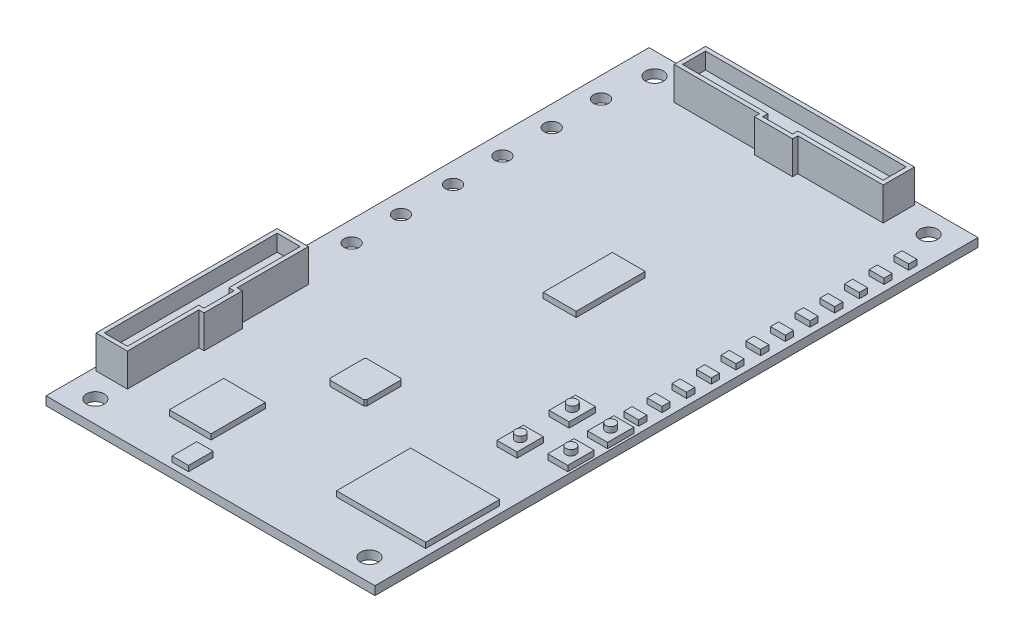
SolidWorks part; units mm, degrees
material "A-Glass Fiber"
ref_plane "Front Plane" through (0, 0, 0) normal (0, 0, 1) x (1, 0, 0)
ref_plane "Top Plane" through (0, 0, 0) normal (0, 1, 0) x (1, 0, 0)
ref_plane "Right Plane" through (0, 0, 0) normal (1, 0, 0) x (0, 0, -1)
sketch "dxf" plane through (0, 0, 0) normal (0, 1, 0) x (1, 0, 0)
  line L0 (60, 110) -> (0, 110)
  line L1 (0, 110) -> (0, 0)
  line L2 (0, 0) -> (60, 0)
  line L3 (60, 0) -> (60, 110)
  line L4 (1.396, 76.2916) -> (1.2504, 76.4372)
  line L5 (1.2504, 76.4372) -> (0.9591, 76.4372)
  line L6 (0.9591, 76.4372) -> (0.8135, 76.2916)
  line L7 (0.8135, 76.2916) -> (0.8135, 75.7091)
  line L8 (0.8135, 75.7091) -> (0.9591, 75.5635)
  line L9 (0.9591, 75.5635) -> (1.2504, 75.5635)
  line L10 (1.2504, 75.5635) -> (1.396, 75.7091)
  line L11 (1.396, 75.7091) -> (1.396, 76.0004)
  line L12 (1.396, 76.0004) -> (1.1047, 76.0004)
  line L13 (1.7343, 75.5635) -> (1.7343, 76.4372)
  line L14 (1.7343, 76.4372) -> (2.3168, 75.5635)
  line L15 (2.3168, 75.5635) -> (2.3168, 76.4372)
  line L16 (2.6551, 76.4372) -> (2.6551, 75.5635)
  line L17 (2.6551, 75.5635) -> (3.0919, 75.5635)
  line L18 (3.0919, 75.5635) -> (3.2376, 75.7091)
  line L19 (3.2376, 75.7091) -> (3.2376, 76.2916)
  line L20 (3.2376, 76.2916) -> (3.0919, 76.4372)
  line L21 (3.0919, 76.4372) -> (2.6551, 76.4372)
  line L22 (1.396, 48.7916) -> (1.2504, 48.9372)
  line L23 (1.2504, 48.9372) -> (0.9591, 48.9372)
  line L24 (0.9591, 48.9372) -> (0.8135, 48.7916)
  line L25 (0.8135, 48.7916) -> (0.8135, 48.2091)
  line L26 (0.8135, 48.2091) -> (0.9591, 48.0635)
  line L27 (0.9591, 48.0635) -> (1.2504, 48.0635)
  line L28 (1.2504, 48.0635) -> (1.396, 48.2091)
  line L29 (1.396, 48.2091) -> (1.396, 48.5004)
  line L30 (1.396, 48.5004) -> (1.1047, 48.5004)
  line L31 (1.7343, 48.0635) -> (1.7343, 48.9372)
  line L32 (1.7343, 48.9372) -> (2.3168, 48.0635)
  line L33 (2.3168, 48.0635) -> (2.3168, 48.9372)
  line L34 (2.6551, 48.9372) -> (2.6551, 48.0635)
  line L35 (2.6551, 48.0635) -> (3.0919, 48.0635)
  line L36 (3.0919, 48.0635) -> (3.2376, 48.2091)
  line L37 (3.2376, 48.2091) -> (3.2376, 48.7916)
  line L38 (3.2376, 48.7916) -> (3.0919, 48.9372)
  line L39 (3.0919, 48.9372) -> (2.6551, 48.9372)
  line L40 (1.396, 94.0416) -> (1.2504, 94.1872)
  line L41 (1.2504, 94.1872) -> (0.9591, 94.1872)
  line L42 (0.9591, 94.1872) -> (0.8135, 94.0416)
  line L43 (0.8135, 94.0416) -> (0.8135, 93.4591)
  line L44 (0.8135, 93.4591) -> (0.9591, 93.3135)
  line L45 (0.9591, 93.3135) -> (1.2504, 93.3135)
  line L46 (1.2504, 93.3135) -> (1.396, 93.4591)
  line L47 (1.396, 93.4591) -> (1.396, 93.7504)
  line L48 (1.396, 93.7504) -> (1.1047, 93.7504)
  line L49 (1.7343, 93.3135) -> (1.7343, 94.1872)
  line L50 (1.7343, 94.1872) -> (2.3168, 93.3135)
  line L51 (2.3168, 93.3135) -> (2.3168, 94.1872)
  line L52 (2.6551, 94.1872) -> (2.6551, 93.3135)
  line L53 (2.6551, 93.3135) -> (3.0919, 93.3135)
  line L54 (3.0919, 93.3135) -> (3.2376, 93.4591)
  line L55 (3.2376, 93.4591) -> (3.2376, 94.0416)
  line L56 (3.2376, 94.0416) -> (3.0919, 94.1872)
  line L57 (3.0919, 94.1872) -> (2.6551, 94.1872)
  line L58 (0.5635, 85.4372) -> (0.5635, 84.8547)
  line L59 (0.5635, 84.8547) -> (0.8547, 84.5635)
  line L60 (0.8547, 84.5635) -> (1.146, 84.8547)
  line L61 (1.146, 84.8547) -> (1.146, 85.4372)
  line L62 (1.4843, 84.5635) -> (1.4843, 85.4372)
  line L63 (1.4843, 85.4372) -> (1.9212, 85.4372)
  line L64 (1.9212, 85.4372) -> (2.0668, 85.2916)
  line L65 (2.0668, 85.2916) -> (2.0668, 85.146)
  line L66 (2.0668, 85.146) -> (1.9212, 85.0004)
  line L67 (1.9212, 85.0004) -> (2.0668, 84.8547)
  line L68 (2.0668, 84.8547) -> (2.0668, 84.7091)
  line L69 (2.0668, 84.7091) -> (1.9212, 84.5635)
  line L70 (1.9212, 84.5635) -> (1.4843, 84.5635)
  line L71 (1.4843, 85.0004) -> (1.9212, 85.0004)
  line L72 (2.4051, 84.5635) -> (2.4051, 85.146)
  line L73 (2.4051, 85.146) -> (2.6963, 85.4372)
  line L74 (2.6963, 85.4372) -> (2.9876, 85.146)
  line L75 (2.9876, 85.146) -> (2.9876, 84.5635)
  line L76 (2.4051, 85.0004) -> (2.9876, 85.0004)
  line L77 (3.6171, 84.5635) -> (3.6171, 85.4372)
  line L78 (3.3259, 85.4372) -> (3.9083, 85.4372)
  line L79 (4.5379, 84.5635) -> (4.5379, 85.4372)
  line L80 (4.2466, 85.4372) -> (4.8291, 85.4372)
  line L81 (1.646, 57.5416) -> (1.5004, 57.6872)
  line L82 (1.5004, 57.6872) -> (1.2091, 57.6872)
  line L83 (1.2091, 57.6872) -> (1.0635, 57.5416)
  line L84 (1.0635, 57.5416) -> (1.0635, 56.9591)
  line L85 (1.0635, 56.9591) -> (1.2091, 56.8135)
  line L86 (1.2091, 56.8135) -> (1.5004, 56.8135)
  line L87 (1.5004, 56.8135) -> (1.646, 56.9591)
  line L88 (1.9843, 56.8135) -> (1.9843, 57.6872)
  line L89 (1.9843, 57.2504) -> (2.5668, 57.2504)
  line L90 (2.5668, 57.6872) -> (2.5668, 56.8135)
  line L91 (2.9051, 56.8135) -> (2.9051, 57.6872)
  line L92 (2.9051, 57.6872) -> (3.3419, 57.6872)
  line L93 (3.3419, 57.6872) -> (3.4876, 57.5416)
  line L94 (3.4876, 57.5416) -> (3.4876, 57.2504)
  line L95 (3.4876, 57.2504) -> (3.3419, 57.1047)
  line L96 (3.3419, 57.1047) -> (2.9051, 57.1047)
  line L97 (3.1963, 57.1047) -> (3.4876, 56.8135)
  line L98 (4.4084, 57.5416) -> (4.2627, 57.6872)
  line L99 (4.2627, 57.6872) -> (3.9715, 57.6872)
  line L100 (3.9715, 57.6872) -> (3.8259, 57.5416)
  line L101 (3.8259, 57.5416) -> (3.8259, 56.9591)
  line L102 (3.8259, 56.9591) -> (3.9715, 56.8135)
  line L103 (3.9715, 56.8135) -> (4.2627, 56.8135)
  line L104 (4.2627, 56.8135) -> (4.4084, 56.9591)
  line L105 (4.4084, 56.9591) -> (4.4084, 57.2504)
  line L106 (4.4084, 57.2504) -> (4.1171, 57.2504)
  line L107 (1.0635, 67.4372) -> (1.0635, 66.5635)
  line L108 (1.0635, 66.5635) -> (1.646, 66.5635)
  line L109 (2.4212, 67.4372) -> (2.1299, 67.4372)
  line L110 (2.1299, 67.4372) -> (1.9843, 67.2916)
  line L111 (1.9843, 67.2916) -> (1.9843, 66.7091)
  line L112 (1.9843, 66.7091) -> (2.1299, 66.5635)
  line L113 (2.1299, 66.5635) -> (2.4212, 66.5635)
  line L114 (2.4212, 66.5635) -> (2.5668, 66.7091)
  line L115 (2.5668, 66.7091) -> (2.5668, 67.2916)
  line L116 (2.5668, 67.2916) -> (2.4212, 67.4372)
  line L117 (2.9051, 66.5635) -> (2.9051, 67.146)
  line L118 (2.9051, 67.146) -> (3.1963, 67.4372)
  line L119 (3.1963, 67.4372) -> (3.4876, 67.146)
  line L120 (3.4876, 67.146) -> (3.4876, 66.5635)
  line L121 (2.9051, 67.0004) -> (3.4876, 67.0004)
  line L122 (3.8259, 67.4372) -> (3.8259, 66.5635)
  line L123 (3.8259, 66.5635) -> (4.2627, 66.5635)
  line L124 (4.2627, 66.5635) -> (4.4084, 66.7091)
  line L125 (4.4084, 66.7091) -> (4.4084, 67.2916)
  line L126 (4.4084, 67.2916) -> (4.2627, 67.4372)
  line L127 (4.2627, 67.4372) -> (3.8259, 67.4372)
  line L128 (1.7119, 38.2881) -> (1.2957, 38.2881)
  line L129 (1.2957, 38.2881) -> (1.0876, 38.4962)
  line L130 (1.0876, 38.4962) -> (1.2957, 38.7043)
  line L131 (1.2957, 38.7043) -> (1.7119, 38.7043)
  line L132 (1.3997, 38.2881) -> (1.3997, 38.7043)
  line L133 (1.0876, 38.9327) -> (1.6078, 38.9327)
  line L134 (1.6078, 38.9327) -> (1.7119, 39.0367)
  line L135 (1.7119, 39.0367) -> (1.7119, 39.2448)
  line L136 (1.7119, 39.2448) -> (1.6078, 39.3489)
  line L137 (1.6078, 39.3489) -> (1.0876, 39.3489)
  line L138 (1.0876, 39.5772) -> (1.7119, 39.9934)
  line L139 (1.0876, 39.9934) -> (1.7119, 39.5772)
  line L140 (1.1916, 35.9543) -> (1.0876, 35.8503)
  line L141 (1.0876, 35.8503) -> (1.0876, 35.6422)
  line L142 (1.0876, 35.6422) -> (1.1916, 35.5381)
  line L143 (1.1916, 35.5381) -> (1.6078, 35.5381)
  line L144 (1.6078, 35.5381) -> (1.7119, 35.6422)
  line L145 (1.7119, 35.6422) -> (1.7119, 35.8503)
  line L146 (1.7119, 35.8503) -> (1.6078, 35.9543)
  line L147 (1.6078, 35.9543) -> (1.3997, 35.9543)
  line L148 (1.3997, 35.9543) -> (1.3997, 35.7462)
  line L149 (1.7119, 36.1827) -> (1.0876, 36.1827)
  line L150 (1.0876, 36.1827) -> (1.7119, 36.5989)
  line L151 (1.7119, 36.5989) -> (1.0876, 36.5989)
  line L152 (1.0876, 36.8272) -> (1.7119, 36.8272)
  line L153 (1.7119, 36.8272) -> (1.7119, 37.1394)
  line L154 (1.7119, 37.1394) -> (1.6078, 37.2434)
  line L155 (1.6078, 37.2434) -> (1.1916, 37.2434)
  line L156 (1.1916, 37.2434) -> (1.0876, 37.1394)
  line L157 (1.0876, 37.1394) -> (1.0876, 36.8272)
  line L158 (1.1916, 30.9543) -> (1.0876, 30.8503)
  line L159 (1.0876, 30.8503) -> (1.0876, 30.6422)
  line L160 (1.0876, 30.6422) -> (1.1916, 30.5381)
  line L161 (1.1916, 30.5381) -> (1.6078, 30.5381)
  line L162 (1.6078, 30.5381) -> (1.7119, 30.6422)
  line L163 (1.7119, 30.6422) -> (1.7119, 30.8503)
  line L164 (1.7119, 30.8503) -> (1.6078, 30.9543)
  line L165 (1.6078, 30.9543) -> (1.3997, 30.9543)
  line L166 (1.3997, 30.9543) -> (1.3997, 30.7462)
  line L167 (1.7119, 31.1827) -> (1.0876, 31.1827)
  line L168 (1.0876, 31.1827) -> (1.7119, 31.5989)
  line L169 (1.7119, 31.5989) -> (1.0876, 31.5989)
  line L170 (1.0876, 31.8272) -> (1.7119, 31.8272)
  line L171 (1.7119, 31.8272) -> (1.7119, 32.1394)
  line L172 (1.7119, 32.1394) -> (1.6078, 32.2434)
  line L173 (1.6078, 32.2434) -> (1.1916, 32.2434)
  line L174 (1.1916, 32.2434) -> (1.0876, 32.1394)
  line L175 (1.0876, 32.1394) -> (1.0876, 31.8272)
  line L176 (1.7119, 28.5381) -> (1.0876, 28.5381)
  line L177 (1.0876, 28.5381) -> (1.0876, 28.8503)
  line L178 (1.0876, 28.8503) -> (1.1916, 28.9543)
  line L179 (1.1916, 28.9543) -> (1.2957, 28.9543)
  line L180 (1.2957, 28.9543) -> (1.3997, 28.8503)
  line L181 (1.3997, 28.8503) -> (1.5038, 28.9543)
  line L182 (1.5038, 28.9543) -> (1.6078, 28.9543)
  line L183 (1.6078, 28.9543) -> (1.7119, 28.8503)
  line L184 (1.7119, 28.8503) -> (1.7119, 28.5381)
  line L185 (1.3997, 28.5381) -> (1.3997, 28.8503)
  line L186 (1.1916, 26.4543) -> (1.0876, 26.3503)
  line L187 (1.0876, 26.3503) -> (1.0876, 26.1422)
  line L188 (1.0876, 26.1422) -> (1.1916, 26.0381)
  line L189 (1.1916, 26.0381) -> (1.6078, 26.0381)
  line L190 (1.6078, 26.0381) -> (1.7119, 26.1422)
  line L191 (1.7119, 26.1422) -> (1.7119, 26.3503)
  line L192 (1.7119, 26.3503) -> (1.6078, 26.4543)
  line L193 (1.6078, 26.4543) -> (1.3997, 26.4543)
  line L194 (1.3997, 26.4543) -> (1.3997, 26.2462)
  line L195 (1.7119, 23.5381) -> (1.0876, 23.5381)
  line L196 (1.0876, 23.5381) -> (1.0876, 23.8503)
  line L197 (1.0876, 23.8503) -> (1.1916, 23.9543)
  line L198 (1.1916, 23.9543) -> (1.3997, 23.9543)
  line L199 (1.3997, 23.9543) -> (1.5038, 23.8503)
  line L200 (1.5038, 23.8503) -> (1.5038, 23.5381)
  line L201 (1.5038, 23.7462) -> (1.7119, 23.9543)
  line L202 (1.0457, 21.0381) -> (0.8376, 21.2462)
  line L203 (0.8376, 21.2462) -> (1.4619, 21.2462)
  line L204 (1.4619, 21.0381) -> (1.4619, 21.4543)
  line L205 (1.1916, 18.2043) -> (1.0876, 18.1003)
  line L206 (1.0876, 18.1003) -> (1.0876, 17.8922)
  line L207 (1.0876, 17.8922) -> (1.1916, 17.7881)
  line L208 (1.1916, 17.7881) -> (1.6078, 17.7881)
  line L209 (1.6078, 17.7881) -> (1.7119, 17.8922)
  line L210 (1.7119, 17.8922) -> (1.7119, 18.1003)
  line L211 (1.7119, 18.1003) -> (1.6078, 18.2043)
  line L212 (1.1916, 18.8489) -> (1.0876, 18.7448)
  line L213 (1.0876, 18.7448) -> (1.0876, 18.5367)
  line L214 (1.0876, 18.5367) -> (1.1916, 18.4327)
  line L215 (1.1916, 18.4327) -> (1.6078, 18.4327)
  line L216 (1.6078, 18.4327) -> (1.7119, 18.5367)
  line L217 (1.7119, 18.5367) -> (1.7119, 18.7448)
  line L218 (1.7119, 18.7448) -> (1.6078, 18.8489)
  line L219 (1.6078, 18.8489) -> (1.3997, 18.8489)
  line L220 (1.3997, 18.8489) -> (1.3997, 18.6408)
  line L221 (1.7119, 19.0772) -> (1.0876, 19.0772)
  line L222 (1.0876, 19.0772) -> (1.7119, 19.4934)
  line L223 (1.7119, 19.4934) -> (1.0876, 19.4934)
  line L224 (1.0876, 19.7218) -> (1.7119, 19.7218)
  line L225 (1.7119, 19.7218) -> (1.7119, 20.0339)
  line L226 (1.7119, 20.0339) -> (1.6078, 20.138)
  line L227 (1.6078, 20.138) -> (1.1916, 20.138)
  line L228 (1.1916, 20.138) -> (1.0876, 20.0339)
  line L229 (1.0876, 20.0339) -> (1.0876, 19.7218)
  line L230 (0.8376, 16.0381) -> (1.4619, 16.0381)
  line L231 (1.4619, 16.0381) -> (1.4619, 16.4543)
  line L232 (1.7119, 13.5381) -> (1.0876, 13.5381)
  line L233 (1.3997, 13.5381) -> (1.3997, 13.9543)
  line L234 (1.0876, 13.9543) -> (1.7119, 13.9543)
  line L235 (1.1916, 10.4543) -> (1.0876, 10.3503)
  line L236 (1.0876, 10.3503) -> (1.0876, 10.1422)
  line L237 (1.0876, 10.1422) -> (1.1916, 10.0381)
  line L238 (1.1916, 10.0381) -> (1.6078, 10.0381)
  line L239 (1.6078, 10.0381) -> (1.7119, 10.1422)
  line L240 (1.7119, 10.1422) -> (1.7119, 10.3503)
  line L241 (1.7119, 10.3503) -> (1.6078, 10.4543)
  line L242 (1.0876, 10.6827) -> (1.5038, 10.6827)
  line L243 (1.5038, 10.6827) -> (1.7119, 10.8908)
  line L244 (1.7119, 10.8908) -> (1.5038, 11.0989)
  line L245 (1.5038, 11.0989) -> (1.0876, 11.0989)
  line L246 (1.0876, 11.3272) -> (1.7119, 11.3272)
  line L247 (1.7119, 11.3272) -> (1.7119, 11.6394)
  line L248 (1.7119, 11.6394) -> (1.6078, 11.7434)
  line L249 (1.6078, 11.7434) -> (1.1916, 11.7434)
  line L250 (1.1916, 11.7434) -> (1.0876, 11.6394)
  line L251 (1.0876, 11.6394) -> (1.0876, 11.3272)
  line L252 (1.0876, 11.9718) -> (1.7119, 11.9718)
  line L253 (1.7119, 11.9718) -> (1.7119, 12.2839)
  line L254 (1.7119, 12.2839) -> (1.6078, 12.388)
  line L255 (1.6078, 12.388) -> (1.1916, 12.388)
  line L256 (1.1916, 12.388) -> (1.0876, 12.2839)
  line L257 (1.0876, 12.2839) -> (1.0876, 11.9718)
  line L258 (49.3262, 9.0762) -> (49.3262, 10.0246)
  line L259 (49.3262, 10.0246) -> (49.8004, 10.0246)
  line L260 (49.8004, 10.0246) -> (49.9585, 9.8665)
  line L261 (49.9585, 9.8665) -> (49.9585, 9.7085)
  line L262 (49.9585, 9.7085) -> (49.8004, 9.5504)
  line L263 (49.8004, 9.5504) -> (49.9585, 9.3923)
  line L264 (49.9585, 9.3923) -> (49.9585, 9.2343)
  line L265 (49.9585, 9.2343) -> (49.8004, 9.0762)
  line L266 (49.8004, 9.0762) -> (49.3262, 9.0762)
  line L267 (49.3262, 9.5504) -> (49.8004, 9.5504)
  line L268 (50.3391, 9.0762) -> (50.3391, 10.0246)
  line L269 (50.3391, 10.0246) -> (50.6552, 9.7085)
  line L270 (50.6552, 9.7085) -> (50.9713, 10.0246)
  line L271 (50.9713, 10.0246) -> (50.9713, 9.0762)
  line L272 (51.9842, 9.8665) -> (51.8261, 10.0246)
  line L273 (51.8261, 10.0246) -> (51.51, 10.0246)
  line L274 (51.51, 10.0246) -> (51.3519, 9.8665)
  line L275 (51.3519, 9.8665) -> (51.3519, 9.7085)
  line L276 (51.3519, 9.7085) -> (51.51, 9.5504)
  line L277 (51.51, 9.5504) -> (51.8261, 9.5504)
  line L278 (51.8261, 9.5504) -> (51.9842, 9.3923)
  line L279 (51.9842, 9.3923) -> (51.9842, 9.2343)
  line L280 (51.9842, 9.2343) -> (51.8261, 9.0762)
  line L281 (51.8261, 9.0762) -> (51.51, 9.0762)
  line L282 (51.51, 9.0762) -> (51.3519, 9.2343)
  line L283 (53.3777, 9.7085) -> (53.6938, 9.0762)
  line L284 (53.6938, 9.0762) -> (54.0099, 9.7085)
  line L285 (54.3905, 9.2343) -> (54.3905, 9.8665)
  line L286 (54.3905, 9.8665) -> (54.5486, 10.0246)
  line L287 (54.5486, 10.0246) -> (54.8647, 10.0246)
  line L288 (54.8647, 10.0246) -> (55.0228, 9.8665)
  line L289 (55.0228, 9.8665) -> (55.0228, 9.2343)
  line L290 (55.0228, 9.2343) -> (54.8647, 9.0762)
  line L291 (54.8647, 9.0762) -> (54.5486, 9.0762)
  line L292 (54.5486, 9.0762) -> (54.3905, 9.2343)
  line L293 (54.3905, 9.2343) -> (55.0228, 9.8665)
  line L294 (55.4034, 9.0762) -> (55.4034, 9.2343)
  line L295 (55.4034, 9.2343) -> (55.5615, 9.2343)
  line L296 (55.5615, 9.2343) -> (55.5615, 9.0762)
  line L297 (55.5615, 9.0762) -> (55.4034, 9.0762)
  line L298 (55.9098, 9.7085) -> (56.226, 10.0246)
  line L299 (56.226, 10.0246) -> (56.226, 9.0762)
  line L300 (55.9098, 9.0762) -> (56.5421, 9.0762)
  line L301 (53.5762, 7.7343) -> (53.7343, 7.5762)
  line L302 (53.7343, 7.5762) -> (53.8923, 7.5762)
  line L303 (53.8923, 7.5762) -> (54.0504, 7.7343)
  line L304 (54.0504, 7.7343) -> (54.0504, 8.5246)
  line L305 (53.8923, 8.5246) -> (54.2085, 8.5246)
  line L306 (54.5891, 8.5246) -> (54.5891, 7.5762)
  line L307 (54.5891, 7.5762) -> (54.9052, 7.8923)
  line L308 (54.9052, 7.8923) -> (55.2213, 7.5762)
  line L309 (55.2213, 7.5762) -> (55.2213, 8.5246)
  line L310 (56.2342, 8.5246) -> (55.6019, 8.5246)
  line L311 (55.6019, 8.5246) -> (55.6019, 7.5762)
  line L312 (55.6019, 7.5762) -> (56.2342, 7.5762)
  line L313 (55.6019, 8.0504) -> (55.9181, 8.0504)
  line L314 (1.1916, 33.0381) -> (1.0876, 33.1422)
  line L315 (1.0876, 33.1422) -> (1.0876, 33.3503)
  line L316 (1.0876, 33.3503) -> (1.1916, 33.4543)
  line L317 (1.1916, 33.4543) -> (1.2957, 33.4543)
  line L318 (1.2957, 33.4543) -> (1.3997, 33.3503)
  line L319 (1.3997, 33.3503) -> (1.3997, 33.2462)
  line L320 (1.3997, 33.3503) -> (1.5038, 33.4543)
  line L321 (1.5038, 33.4543) -> (1.6078, 33.4543)
  line L322 (1.6078, 33.4543) -> (1.7119, 33.3503)
  line L323 (1.7119, 33.3503) -> (1.7119, 33.1422)
  line L324 (1.7119, 33.1422) -> (1.6078, 33.0381)
  line L325 (1.0876, 33.6827) -> (1.5038, 33.6827)
  line L326 (1.5038, 33.6827) -> (1.7119, 33.8908)
  line L327 (1.7119, 33.8908) -> (1.5038, 34.0989)
  line L328 (1.5038, 34.0989) -> (1.0876, 34.0989)
  line L329 (1.1916, 34.3272) -> (1.0876, 34.4313)
  line L330 (1.0876, 34.4313) -> (1.0876, 34.6394)
  line L331 (1.0876, 34.6394) -> (1.1916, 34.7434)
  line L332 (1.1916, 34.7434) -> (1.2957, 34.7434)
  line L333 (1.2957, 34.7434) -> (1.3997, 34.6394)
  line L334 (1.3997, 34.6394) -> (1.3997, 34.5353)
  line L335 (1.3997, 34.6394) -> (1.5038, 34.7434)
  line L336 (1.5038, 34.7434) -> (1.6078, 34.7434)
  line L337 (1.6078, 34.7434) -> (1.7119, 34.6394)
  line L338 (1.7119, 34.6394) -> (1.7119, 34.4313)
  line L339 (1.7119, 34.4313) -> (1.6078, 34.3272)
  line L340 (31.8635, 59.346) -> (32.1547, 59.6372)
  line L341 (32.1547, 59.6372) -> (32.1547, 58.7635)
  line L342 (31.8635, 58.7635) -> (32.446, 58.7635)
  line L343 (30.946, 58.7635) -> (30.3635, 58.7635)
  line L344 (30.3635, 58.7635) -> (30.946, 59.346)
  line L345 (30.946, 59.346) -> (30.946, 59.4916)
  line L346 (30.946, 59.4916) -> (30.8004, 59.6372)
  line L347 (30.8004, 59.6372) -> (30.5091, 59.6372)
  line L348 (30.5091, 59.6372) -> (30.3635, 59.4916)
  line L349 (44.3492, 30.0508) -> (43.7002, 30.0508)
  line L350 (43.7002, 30.0508) -> (43.7002, 30.3753)
  line L351 (43.7002, 30.3753) -> (43.8084, 30.4834)
  line L352 (43.8084, 30.4834) -> (43.9166, 30.4834)
  line L353 (43.9166, 30.4834) -> (44.0247, 30.3753)
  line L354 (44.0247, 30.3753) -> (44.1329, 30.4834)
  line L355 (44.1329, 30.4834) -> (44.241, 30.4834)
  line L356 (44.241, 30.4834) -> (44.3492, 30.3753)
  line L357 (44.3492, 30.3753) -> (44.3492, 30.0508)
  line L358 (44.0247, 30.0508) -> (44.0247, 30.3753)
  line L359 (44.3492, 31.174) -> (44.3492, 30.7414)
  line L360 (44.3492, 30.7414) -> (43.9166, 31.174)
  line L361 (43.9166, 31.174) -> (43.8084, 31.174)
  line L362 (43.8084, 31.174) -> (43.7002, 31.0659)
  line L363 (43.7002, 31.0659) -> (43.7002, 30.8495)
  line L364 (43.7002, 30.8495) -> (43.8084, 30.7414)
  line L365 (16.8381, 40.4381) -> (16.8381, 40.821)
  line L366 (16.8381, 40.821) -> (17.0295, 41.0124)
  line L367 (17.0295, 41.0124) -> (17.221, 40.821)
  line L368 (17.221, 40.821) -> (17.221, 40.4381)
  line L369 (16.8381, 40.7252) -> (17.221, 40.7252)
  line L370 (17.4366, 41.0124) -> (17.4366, 40.5338)
  line L371 (17.4366, 40.5338) -> (17.5323, 40.4381)
  line L372 (17.5323, 40.4381) -> (17.7238, 40.4381)
  line L373 (17.7238, 40.4381) -> (17.8195, 40.5338)
  line L374 (17.8195, 40.5338) -> (17.8195, 41.0124)
  line L375 (18.0351, 41.0124) -> (18.418, 40.4381)
  line L376 (18.418, 41.0124) -> (18.0351, 40.4381)
  line L377 (18.6336, 40.3424) -> (19.0165, 40.3424)
  line L378 (19.615, 41.0124) -> (19.2321, 41.0124)
  line L379 (19.2321, 41.0124) -> (19.2321, 40.4381)
  line L380 (19.2321, 40.4381) -> (19.615, 40.4381)
  line L381 (19.2321, 40.7252) -> (19.4236, 40.7252)
  line L382 (19.8306, 40.4381) -> (19.8306, 41.0124)
  line L383 (19.8306, 41.0124) -> (20.2135, 40.4381)
  line L384 (20.2135, 40.4381) -> (20.2135, 41.0124)
  line L385 (46.2838, 108.3508) -> (46.2838, 109.0498)
  line L386 (46.0508, 109.0498) -> (46.5168, 109.0498)
  line L387 (46.7874, 108.3508) -> (46.7874, 109.0498)
  line L388 (46.7874, 108.7003) -> (47.2534, 108.7003)
  line L389 (47.2534, 109.0498) -> (47.2534, 108.3508)
  line L390 (43.9168, 108.9333) -> (43.8003, 109.0498)
  line L391 (43.8003, 109.0498) -> (43.5673, 109.0498)
  line L392 (43.5673, 109.0498) -> (43.4508, 108.9333)
  line L393 (43.4508, 108.9333) -> (43.4508, 108.4673)
  line L394 (43.4508, 108.4673) -> (43.5673, 108.3508)
  line L395 (43.5673, 108.3508) -> (43.8003, 108.3508)
  line L396 (43.8003, 108.3508) -> (43.9168, 108.4673)
  line L397 (44.1874, 108.4673) -> (44.1874, 108.9333)
  line L398 (44.1874, 108.9333) -> (44.3039, 109.0498)
  line L399 (44.3039, 109.0498) -> (44.5369, 109.0498)
  line L400 (44.5369, 109.0498) -> (44.6534, 108.9333)
  line L401 (44.6534, 108.9333) -> (44.6534, 108.4673)
  line L402 (44.6534, 108.4673) -> (44.5369, 108.3508)
  line L403 (44.5369, 108.3508) -> (44.3039, 108.3508)
  line L404 (44.3039, 108.3508) -> (44.1874, 108.4673)
  line L405 (44.1874, 108.4673) -> (44.6534, 108.9333)
  line L406 (41.4168, 108.9333) -> (41.3003, 109.0498)
  line L407 (41.3003, 109.0498) -> (41.0673, 109.0498)
  line L408 (41.0673, 109.0498) -> (40.9508, 108.9333)
  line L409 (40.9508, 108.9333) -> (40.9508, 108.4673)
  line L410 (40.9508, 108.4673) -> (41.0673, 108.3508)
  line L411 (41.0673, 108.3508) -> (41.3003, 108.3508)
  line L412 (41.3003, 108.3508) -> (41.4168, 108.4673)
  line L413 (41.6874, 108.8168) -> (41.9204, 109.0498)
  line L414 (41.9204, 109.0498) -> (41.9204, 108.3508)
  line L415 (41.6874, 108.3508) -> (42.1534, 108.3508)
  line L416 (38.9168, 108.9333) -> (38.8003, 109.0498)
  line L417 (38.8003, 109.0498) -> (38.5673, 109.0498)
  line L418 (38.5673, 109.0498) -> (38.4508, 108.9333)
  line L419 (38.4508, 108.9333) -> (38.4508, 108.4673)
  line L420 (38.4508, 108.4673) -> (38.5673, 108.3508)
  line L421 (38.5673, 108.3508) -> (38.8003, 108.3508)
  line L422 (38.8003, 108.3508) -> (38.9168, 108.4673)
  line L423 (39.6534, 108.3508) -> (39.1874, 108.3508)
  line L424 (39.1874, 108.3508) -> (39.6534, 108.8168)
  line L425 (39.6534, 108.8168) -> (39.6534, 108.9333)
  line L426 (39.6534, 108.9333) -> (39.5369, 109.0498)
  line L427 (39.5369, 109.0498) -> (39.3039, 109.0498)
  line L428 (39.3039, 109.0498) -> (39.1874, 108.9333)
  line L429 (36.3168, 108.9333) -> (36.2003, 109.0498)
  line L430 (36.2003, 109.0498) -> (35.9673, 109.0498)
  line L431 (35.9673, 109.0498) -> (35.8508, 108.9333)
  line L432 (35.8508, 108.9333) -> (35.8508, 108.4673)
  line L433 (35.8508, 108.4673) -> (35.9673, 108.3508)
  line L434 (35.9673, 108.3508) -> (36.2003, 108.3508)
  line L435 (36.2003, 108.3508) -> (36.3168, 108.4673)
  line L436 (36.5874, 108.9333) -> (36.7039, 109.0498)
  line L437 (36.7039, 109.0498) -> (36.9369, 109.0498)
  line L438 (36.9369, 109.0498) -> (37.0534, 108.9333)
  line L439 (37.0534, 108.9333) -> (37.0534, 108.8168)
  line L440 (37.0534, 108.8168) -> (36.9369, 108.7003)
  line L441 (36.9369, 108.7003) -> (36.8204, 108.7003)
  line L442 (36.9369, 108.7003) -> (37.0534, 108.5838)
  line L443 (37.0534, 108.5838) -> (37.0534, 108.4673)
  line L444 (37.0534, 108.4673) -> (36.9369, 108.3508)
  line L445 (36.9369, 108.3508) -> (36.7039, 108.3508)
  line L446 (36.7039, 108.3508) -> (36.5874, 108.4673)
  line L447 (33.6168, 108.9333) -> (33.5003, 109.0498)
  line L448 (33.5003, 109.0498) -> (33.2673, 109.0498)
  line L449 (33.2673, 109.0498) -> (33.1508, 108.9333)
  line L450 (33.1508, 108.9333) -> (33.1508, 108.4673)
  line L451 (33.1508, 108.4673) -> (33.2673, 108.3508)
  line L452 (33.2673, 108.3508) -> (33.5003, 108.3508)
  line L453 (33.5003, 108.3508) -> (33.6168, 108.4673)
  line L454 (34.2369, 108.3508) -> (34.2369, 109.0498)
  line L455 (34.2369, 109.0498) -> (33.8874, 108.7003)
  line L456 (33.8874, 108.7003) -> (34.3534, 108.7003)
  line L457 (31.2168, 108.9333) -> (31.1003, 109.0498)
  line L458 (31.1003, 109.0498) -> (30.8673, 109.0498)
  line L459 (30.8673, 109.0498) -> (30.7508, 108.9333)
  line L460 (30.7508, 108.9333) -> (30.7508, 108.4673)
  line L461 (30.7508, 108.4673) -> (30.8673, 108.3508)
  line L462 (30.8673, 108.3508) -> (31.1003, 108.3508)
  line L463 (31.1003, 108.3508) -> (31.2168, 108.4673)
  line L464 (31.9534, 109.0498) -> (31.4874, 109.0498)
  line L465 (31.4874, 109.0498) -> (31.4874, 108.7003)
  line L466 (31.4874, 108.7003) -> (31.7204, 108.8168)
  line L467 (31.7204, 108.8168) -> (31.8369, 108.8168)
  line L468 (31.8369, 108.8168) -> (31.9534, 108.7003)
  line L469 (31.9534, 108.7003) -> (31.9534, 108.4673)
  line L470 (31.9534, 108.4673) -> (31.8369, 108.3508)
  line L471 (31.8369, 108.3508) -> (31.6039, 108.3508)
  line L472 (31.6039, 108.3508) -> (31.4874, 108.4673)
  line L473 (28.7168, 108.9333) -> (28.6003, 109.0498)
  line L474 (28.6003, 109.0498) -> (28.3673, 109.0498)
  line L475 (28.3673, 109.0498) -> (28.2508, 108.9333)
  line L476 (28.2508, 108.9333) -> (28.2508, 108.4673)
  line L477 (28.2508, 108.4673) -> (28.3673, 108.3508)
  line L478 (28.3673, 108.3508) -> (28.6003, 108.3508)
  line L479 (28.6003, 108.3508) -> (28.7168, 108.4673)
  line L480 (29.4534, 109.0498) -> (29.2204, 108.9333)
  line L481 (29.2204, 108.9333) -> (28.9874, 108.7003)
  line L482 (28.9874, 108.7003) -> (28.9874, 108.4673)
  line L483 (28.9874, 108.4673) -> (29.1039, 108.3508)
  line L484 (29.1039, 108.3508) -> (29.3369, 108.3508)
  line L485 (29.3369, 108.3508) -> (29.4534, 108.4673)
  line L486 (29.4534, 108.4673) -> (29.4534, 108.5838)
  line L487 (29.4534, 108.5838) -> (29.3369, 108.7003)
  line L488 (29.3369, 108.7003) -> (28.9874, 108.7003)
  line L489 (26.2168, 108.9333) -> (26.1003, 109.0498)
  line L490 (26.1003, 109.0498) -> (25.8673, 109.0498)
  line L491 (25.8673, 109.0498) -> (25.7508, 108.9333)
  line L492 (25.7508, 108.9333) -> (25.7508, 108.4673)
  line L493 (25.7508, 108.4673) -> (25.8673, 108.3508)
  line L494 (25.8673, 108.3508) -> (26.1003, 108.3508)
  line L495 (26.1003, 108.3508) -> (26.2168, 108.4673)
  line L496 (26.4874, 109.0498) -> (26.9534, 109.0498)
  line L497 (26.9534, 109.0498) -> (26.9534, 108.9333)
  line L498 (26.9534, 108.9333) -> (26.4874, 108.4673)
  line L499 (26.4874, 108.4673) -> (26.4874, 108.3508)
  line L500 (23.6168, 108.9333) -> (23.5003, 109.0498)
  line L501 (23.5003, 109.0498) -> (23.2673, 109.0498)
  line L502 (23.2673, 109.0498) -> (23.1508, 108.9333)
  line L503 (23.1508, 108.9333) -> (23.1508, 108.4673)
  line L504 (23.1508, 108.4673) -> (23.2673, 108.3508)
  line L505 (23.2673, 108.3508) -> (23.5003, 108.3508)
  line L506 (23.5003, 108.3508) -> (23.6168, 108.4673)
  line L507 (23.8874, 108.9333) -> (24.0039, 109.0498)
  line L508 (24.0039, 109.0498) -> (24.2369, 109.0498)
  line L509 (24.2369, 109.0498) -> (24.3534, 108.9333)
  line L510 (24.3534, 108.9333) -> (24.3534, 108.8168)
  line L511 (24.3534, 108.8168) -> (24.2369, 108.7003)
  line L512 (24.2369, 108.7003) -> (24.3534, 108.5838)
  line L513 (24.3534, 108.5838) -> (24.3534, 108.4673)
  line L514 (24.3534, 108.4673) -> (24.2369, 108.3508)
  line L515 (24.2369, 108.3508) -> (24.0039, 108.3508)
  line L516 (24.0039, 108.3508) -> (23.8874, 108.4673)
  line L517 (23.8874, 108.4673) -> (23.8874, 108.5838)
  line L518 (23.8874, 108.5838) -> (24.0039, 108.7003)
  line L519 (24.0039, 108.7003) -> (23.8874, 108.8168)
  line L520 (23.8874, 108.8168) -> (23.8874, 108.9333)
  line L521 (24.0039, 108.7003) -> (24.2369, 108.7003)
  line L522 (21.0168, 108.9333) -> (20.9003, 109.0498)
  line L523 (20.9003, 109.0498) -> (20.6673, 109.0498)
  line L524 (20.6673, 109.0498) -> (20.5508, 108.9333)
  line L525 (20.5508, 108.9333) -> (20.5508, 108.4673)
  line L526 (20.5508, 108.4673) -> (20.6673, 108.3508)
  line L527 (20.6673, 108.3508) -> (20.9003, 108.3508)
  line L528 (20.9003, 108.3508) -> (21.0168, 108.4673)
  line L529 (21.2874, 108.4673) -> (21.4039, 108.3508)
  line L530 (21.4039, 108.3508) -> (21.6369, 108.3508)
  line L531 (21.6369, 108.3508) -> (21.7534, 108.4673)
  line L532 (21.7534, 108.4673) -> (21.7534, 108.9333)
  line L533 (21.7534, 108.9333) -> (21.6369, 109.0498)
  line L534 (21.6369, 109.0498) -> (21.4039, 109.0498)
  line L535 (21.4039, 109.0498) -> (21.2874, 108.9333)
  line L536 (21.2874, 108.9333) -> (21.2874, 108.8168)
  line L537 (21.2874, 108.8168) -> (21.4039, 108.7003)
  line L538 (21.4039, 108.7003) -> (21.7534, 108.7003)
  line L539 (18.2168, 108.9333) -> (18.1003, 109.0498)
  line L540 (18.1003, 109.0498) -> (17.8673, 109.0498)
  line L541 (17.8673, 109.0498) -> (17.7508, 108.9333)
  line L542 (17.7508, 108.9333) -> (17.7508, 108.4673)
  line L543 (17.7508, 108.4673) -> (17.8673, 108.3508)
  line L544 (17.8673, 108.3508) -> (18.1003, 108.3508)
  line L545 (18.1003, 108.3508) -> (18.2168, 108.4673)
  line L546 (18.4874, 108.8168) -> (18.7204, 109.0498)
  line L547 (18.7204, 109.0498) -> (18.7204, 108.3508)
  line L548 (18.4874, 108.3508) -> (18.9534, 108.3508)
  line L549 (19.2241, 108.4673) -> (19.2241, 108.9333)
  line L550 (19.2241, 108.9333) -> (19.3406, 109.0498)
  line L551 (19.3406, 109.0498) -> (19.5736, 109.0498)
  line L552 (19.5736, 109.0498) -> (19.6901, 108.9333)
  line L553 (19.6901, 108.9333) -> (19.6901, 108.4673)
  line L554 (19.6901, 108.4673) -> (19.5736, 108.3508)
  line L555 (19.5736, 108.3508) -> (19.3406, 108.3508)
  line L556 (19.3406, 108.3508) -> (19.2241, 108.4673)
  line L557 (19.2241, 108.4673) -> (19.6901, 108.9333)
  line L558 (15.7168, 108.9333) -> (15.6003, 109.0498)
  line L559 (15.6003, 109.0498) -> (15.3673, 109.0498)
  line L560 (15.3673, 109.0498) -> (15.2508, 108.9333)
  line L561 (15.2508, 108.9333) -> (15.2508, 108.4673)
  line L562 (15.2508, 108.4673) -> (15.3673, 108.3508)
  line L563 (15.3673, 108.3508) -> (15.6003, 108.3508)
  line L564 (15.6003, 108.3508) -> (15.7168, 108.4673)
  line L565 (15.9874, 108.8168) -> (16.2204, 109.0498)
  line L566 (16.2204, 109.0498) -> (16.2204, 108.3508)
  line L567 (15.9874, 108.3508) -> (16.4534, 108.3508)
  line L568 (16.7241, 108.8168) -> (16.9571, 109.0498)
  line L569 (16.9571, 109.0498) -> (16.9571, 108.3508)
  line L570 (16.7241, 108.3508) -> (17.1901, 108.3508)
  line L571 (13.1168, 108.9333) -> (13.0003, 109.0498)
  line L572 (13.0003, 109.0498) -> (12.7673, 109.0498)
  line L573 (12.7673, 109.0498) -> (12.6508, 108.9333)
  line L574 (12.6508, 108.9333) -> (12.6508, 108.4673)
  line L575 (12.6508, 108.4673) -> (12.7673, 108.3508)
  line L576 (12.7673, 108.3508) -> (13.0003, 108.3508)
  line L577 (13.0003, 108.3508) -> (13.1168, 108.4673)
  line L578 (13.3874, 108.8168) -> (13.6204, 109.0498)
  line L579 (13.6204, 109.0498) -> (13.6204, 108.3508)
  line L580 (13.3874, 108.3508) -> (13.8534, 108.3508)
  line L581 (14.5901, 108.3508) -> (14.1241, 108.3508)
  line L582 (14.1241, 108.3508) -> (14.5901, 108.8168)
  line L583 (14.5901, 108.8168) -> (14.5901, 108.9333)
  line L584 (14.5901, 108.9333) -> (14.4736, 109.0498)
  line L585 (14.4736, 109.0498) -> (14.2406, 109.0498)
  line L586 (14.2406, 109.0498) -> (14.1241, 108.9333)
  line L587 (43.0508, 58.1998) -> (43.0508, 57.7671)
  line L588 (43.0508, 57.7671) -> (43.2671, 57.5508)
  line L589 (43.2671, 57.5508) -> (43.4834, 57.7671)
  line L590 (43.4834, 57.7671) -> (43.4834, 58.1998)
  line L591 (43.7414, 57.8753) -> (44.174, 57.8753)
  line L592 (43.9577, 58.0916) -> (43.9577, 57.659)
  line L593 (43.3834, 55.9916) -> (43.2753, 56.0998)
  line L594 (43.2753, 56.0998) -> (43.059, 56.0998)
  line L595 (43.059, 56.0998) -> (42.9508, 55.9916)
  line L596 (42.9508, 55.9916) -> (42.9508, 55.8834)
  line L597 (42.9508, 55.8834) -> (43.059, 55.7753)
  line L598 (43.059, 55.7753) -> (43.2753, 55.7753)
  line L599 (43.2753, 55.7753) -> (43.3834, 55.6671)
  line L600 (43.3834, 55.6671) -> (43.3834, 55.559)
  line L601 (43.3834, 55.559) -> (43.2753, 55.4508)
  line L602 (43.2753, 55.4508) -> (43.059, 55.4508)
  line L603 (43.059, 55.4508) -> (42.9508, 55.559)
  line L604 (44.074, 55.9916) -> (43.9659, 56.0998)
  line L605 (43.9659, 56.0998) -> (43.7495, 56.0998)
  line L606 (43.7495, 56.0998) -> (43.6414, 55.9916)
  line L607 (43.6414, 55.9916) -> (43.6414, 55.559)
  line L608 (43.6414, 55.559) -> (43.7495, 55.4508)
  line L609 (43.7495, 55.4508) -> (43.9659, 55.4508)
  line L610 (43.9659, 55.4508) -> (44.074, 55.559)
  line L611 (44.332, 56.0998) -> (44.332, 55.4508)
  line L612 (44.332, 55.6671) -> (44.7646, 56.0998)
  line L613 (44.4401, 55.7753) -> (44.7646, 55.4508)
  line L614 (43.3834, 53.8916) -> (43.2753, 53.9998)
  line L615 (43.2753, 53.9998) -> (43.059, 53.9998)
  line L616 (43.059, 53.9998) -> (42.9508, 53.8916)
  line L617 (42.9508, 53.8916) -> (42.9508, 53.7834)
  line L618 (42.9508, 53.7834) -> (43.059, 53.6753)
  line L619 (43.059, 53.6753) -> (43.2753, 53.6753)
  line L620 (43.2753, 53.6753) -> (43.3834, 53.5671)
  line L621 (43.3834, 53.5671) -> (43.3834, 53.459)
  line L622 (43.3834, 53.459) -> (43.2753, 53.3508)
  line L623 (43.2753, 53.3508) -> (43.059, 53.3508)
  line L624 (43.059, 53.3508) -> (42.9508, 53.459)
  line L625 (43.6414, 53.9998) -> (43.6414, 53.3508)
  line L626 (43.6414, 53.3508) -> (43.9659, 53.3508)
  line L627 (43.9659, 53.3508) -> (44.074, 53.459)
  line L628 (44.074, 53.459) -> (44.074, 53.8916)
  line L629 (44.074, 53.8916) -> (43.9659, 53.9998)
  line L630 (43.9659, 53.9998) -> (43.6414, 53.9998)
  line L631 (44.6564, 53.9998) -> (44.4401, 53.9998)
  line L632 (44.4401, 53.9998) -> (44.332, 53.8916)
  line L633 (44.332, 53.8916) -> (44.332, 53.459)
  line L634 (44.332, 53.459) -> (44.4401, 53.3508)
  line L635 (44.4401, 53.3508) -> (44.6564, 53.3508)
  line L636 (44.6564, 53.3508) -> (44.7646, 53.459)
  line L637 (44.7646, 53.459) -> (44.7646, 53.8916)
  line L638 (44.7646, 53.8916) -> (44.6564, 53.9998)
  line L639 (43.3251, 49.4001) -> (43.2502, 49.475)
  line L640 (43.2502, 49.475) -> (43.1003, 49.475)
  line L641 (43.1003, 49.475) -> (43.0254, 49.4001)
  line L642 (43.0254, 49.4001) -> (43.0254, 49.1003)
  line L643 (43.0254, 49.1003) -> (43.1003, 49.0254)
  line L644 (43.1003, 49.0254) -> (43.2502, 49.0254)
  line L645 (43.2502, 49.0254) -> (43.3251, 49.1003)
  line L646 (43.3251, 49.1003) -> (43.3251, 49.2502)
  line L647 (43.3251, 49.2502) -> (43.1753, 49.2502)
  line L648 (43.4858, 49.0254) -> (43.4858, 49.475)
  line L649 (43.4858, 49.475) -> (43.7855, 49.0254)
  line L650 (43.7855, 49.0254) -> (43.7855, 49.475)
  line L651 (43.9462, 49.475) -> (43.9462, 49.0254)
  line L652 (43.9462, 49.0254) -> (44.171, 49.0254)
  line L653 (44.171, 49.0254) -> (44.2459, 49.1003)
  line L654 (44.2459, 49.1003) -> (44.2459, 49.4001)
  line L655 (44.2459, 49.4001) -> (44.171, 49.475)
  line L656 (44.171, 49.475) -> (43.9462, 49.475)
  line L657 (43.8084, 32.6834) -> (43.7002, 32.5753)
  line L658 (43.7002, 32.5753) -> (43.7002, 32.359)
  line L659 (43.7002, 32.359) -> (43.8084, 32.2508)
  line L660 (43.8084, 32.2508) -> (44.241, 32.2508)
  line L661 (44.241, 32.2508) -> (44.3492, 32.359)
  line L662 (44.3492, 32.359) -> (44.3492, 32.5753)
  line L663 (44.3492, 32.5753) -> (44.241, 32.6834)
  line L664 (44.241, 32.6834) -> (44.0247, 32.6834)
  line L665 (44.0247, 32.6834) -> (44.0247, 32.4671)
  line L666 (44.3492, 32.9414) -> (43.7002, 32.9414)
  line L667 (43.7002, 32.9414) -> (44.3492, 33.374)
  line L668 (44.3492, 33.374) -> (43.7002, 33.374)
  line L669 (43.7002, 33.632) -> (44.3492, 33.632)
  line L670 (44.3492, 33.632) -> (44.3492, 33.9565)
  line L671 (44.3492, 33.9565) -> (44.241, 34.0646)
  line L672 (44.241, 34.0646) -> (43.8084, 34.0646)
  line L673 (43.8084, 34.0646) -> (43.7002, 33.9565)
  line L674 (43.7002, 33.9565) -> (43.7002, 33.632)
  line L675 (31.5746, 26.0254) -> (31.125, 26.0254)
  line L676 (31.125, 26.0254) -> (31.125, 26.2502)
  line L677 (31.125, 26.2502) -> (31.1999, 26.3251)
  line L678 (31.1999, 26.3251) -> (31.3498, 26.3251)
  line L679 (31.3498, 26.3251) -> (31.4247, 26.2502)
  line L680 (31.4247, 26.2502) -> (31.4247, 26.0254)
  line L681 (31.4247, 26.1753) -> (31.5746, 26.3251)
  line L682 (31.5746, 26.6357) -> (31.125, 26.6357)
  line L683 (31.125, 26.4858) -> (31.125, 26.7855)
  line L684 (31.1999, 27.2459) -> (31.125, 27.171)
  line L685 (31.125, 27.171) -> (31.125, 27.0211)
  line L686 (31.125, 27.0211) -> (31.1999, 26.9462)
  line L687 (31.1999, 26.9462) -> (31.4997, 26.9462)
  line L688 (31.4997, 26.9462) -> (31.5746, 27.0211)
  line L689 (31.5746, 27.0211) -> (31.5746, 27.171)
  line L690 (31.5746, 27.171) -> (31.4997, 27.2459)
  line L691 (52.825, 47.4) -> (49.175, 47.4)
  line L692 (49.175, 47.4) -> (49.175, 42.6)
  line L693 (49.175, 42.6) -> (52.825, 42.6)
  line L694 (52.825, 42.6) -> (52.825, 47.4)
  line L695 (10.65, 102.3) -> (10.65, 97.2)
  line L696 (10.65, 97.2) -> (8.35, 97.2)
  line L697 (8.35, 97.2) -> (8.35, 102.3)
  line L698 (8.35, 102.3) -> (10.65, 102.3)
  line L699 (13.65, 102.3) -> (13.65, 97.2)
  line L700 (13.65, 97.2) -> (11.35, 97.2)
  line L701 (11.35, 97.2) -> (11.35, 102.3)
  line L702 (11.35, 102.3) -> (13.65, 102.3)
  line L703 (16.65, 102.3) -> (16.65, 97.2)
  line L704 (16.65, 97.2) -> (14.35, 97.2)
  line L705 (14.35, 97.2) -> (14.35, 102.3)
  line L706 (14.35, 102.3) -> (16.65, 102.3)
  line L707 (19.65, 102.3) -> (19.65, 97.2)
  line L708 (19.65, 97.2) -> (17.35, 97.2)
  line L709 (17.35, 97.2) -> (17.35, 102.3)
  line L710 (17.35, 102.3) -> (19.65, 102.3)
  line L711 (22.65, 102.3) -> (22.65, 97.2)
  line L712 (22.65, 97.2) -> (20.35, 97.2)
  line L713 (20.35, 97.2) -> (20.35, 102.3)
  line L714 (20.35, 102.3) -> (22.65, 102.3)
  line L715 (25.65, 102.3) -> (25.65, 97.2)
  line L716 (25.65, 97.2) -> (23.35, 97.2)
  line L717 (23.35, 97.2) -> (23.35, 102.3)
  line L718 (23.35, 102.3) -> (25.65, 102.3)
  line L719 (28.65, 102.3) -> (28.65, 97.2)
  line L720 (28.65, 97.2) -> (26.35, 97.2)
  line L721 (26.35, 97.2) -> (26.35, 102.3)
  line L722 (26.35, 102.3) -> (28.65, 102.3)
  line L723 (31.65, 102.3) -> (31.65, 97.2)
  line L724 (31.65, 97.2) -> (29.35, 97.2)
  line L725 (29.35, 97.2) -> (29.35, 102.3)
  line L726 (29.35, 102.3) -> (31.65, 102.3)
  line L727 (34.65, 102.3) -> (34.65, 97.2)
  line L728 (34.65, 97.2) -> (32.35, 97.2)
  line L729 (32.35, 97.2) -> (32.35, 102.3)
  line L730 (32.35, 102.3) -> (34.65, 102.3)
  line L731 (37.65, 102.3) -> (37.65, 97.2)
  line L732 (37.65, 97.2) -> (35.35, 97.2)
  line L733 (35.35, 97.2) -> (35.35, 102.3)
  line L734 (35.35, 102.3) -> (37.65, 102.3)
  line L735 (40.65, 102.3) -> (40.65, 97.2)
  line L736 (40.65, 97.2) -> (38.35, 97.2)
  line L737 (38.35, 97.2) -> (38.35, 102.3)
  line L738 (38.35, 102.3) -> (40.65, 102.3)
  line L739 (43.65, 102.3) -> (43.65, 97.2)
  line L740 (43.65, 97.2) -> (41.35, 97.2)
  line L741 (41.35, 97.2) -> (41.35, 102.3)
  line L742 (41.35, 102.3) -> (43.65, 102.3)
  line L743 (41.25, 93.15) -> (39.75, 93.15)
  line L744 (39.75, 93.15) -> (39.75, 95.85)
  line L745 (39.75, 95.85) -> (41.25, 95.85)
  line L746 (41.25, 95.85) -> (41.25, 93.15)
  line L747 (14.4, 91.15) -> (14.4, 96.35)
  line L748 (14.4, 96.35) -> (17.6, 96.35)
  line L749 (17.6, 96.35) -> (17.6, 91.15)
  line L750 (17.6, 91.15) -> (14.4, 91.15)
  line L751 (17.9, 91.15) -> (17.9, 96.35)
  line L752 (17.9, 96.35) -> (21.1, 96.35)
  line L753 (21.1, 96.35) -> (21.1, 91.15)
  line L754 (21.1, 91.15) -> (17.9, 91.15)
  line L755 (14.4, 84.65) -> (14.4, 89.85)
  line L756 (14.4, 89.85) -> (17.6, 89.85)
  line L757 (17.6, 89.85) -> (17.6, 84.65)
  line L758 (17.6, 84.65) -> (14.4, 84.65)
  line L759 (17.9, 84.65) -> (17.9, 89.85)
  line L760 (17.9, 89.85) -> (21.1, 89.85)
  line L761 (21.1, 89.85) -> (21.1, 84.65)
  line L762 (21.1, 84.65) -> (17.9, 84.65)
  line L763 (21.4, 84.65) -> (21.4, 89.85)
  line L764 (21.4, 89.85) -> (24.6, 89.85)
  line L765 (24.6, 89.85) -> (24.6, 84.65)
  line L766 (24.6, 84.65) -> (21.4, 84.65)
  line L767 (32.5, 82.15) -> (31, 82.15)
  line L768 (31, 82.15) -> (31, 84.85)
  line L769 (31, 84.85) -> (32.5, 84.85)
  line L770 (32.5, 84.85) -> (32.5, 82.15)
  line L771 (17.6, 83.85) -> (17.6, 78.65)
  line L772 (17.6, 78.65) -> (14.4, 78.65)
  line L773 (14.4, 78.65) -> (14.4, 83.85)
  line L774 (14.4, 83.85) -> (17.6, 83.85)
  line L775 (21.1, 83.85) -> (21.1, 78.65)
  line L776 (21.1, 78.65) -> (17.9, 78.65)
  line L777 (17.9, 78.65) -> (17.9, 83.85)
  line L778 (17.9, 83.85) -> (21.1, 83.85)
  line L779 (24.6, 83.85) -> (24.6, 78.65)
  line L780 (24.6, 78.65) -> (21.4, 78.65)
  line L781 (21.4, 78.65) -> (21.4, 83.85)
  line L782 (21.4, 83.85) -> (24.6, 83.85)
  line L783 (12.1, 81.25) -> (12.1, 79.75)
  line L784 (12.1, 79.75) -> (9.4, 79.75)
  line L785 (9.4, 79.75) -> (9.4, 81.25)
  line L786 (9.4, 81.25) -> (12.1, 81.25)
  line L787 (14.4, 73.15) -> (14.4, 78.35)
  line L788 (14.4, 78.35) -> (17.6, 78.35)
  line L789 (17.6, 78.35) -> (17.6, 73.15)
  line L790 (17.6, 73.15) -> (14.4, 73.15)
  line L791 (17.65, 73.15) -> (17.65, 78.35)
  line L792 (17.65, 78.35) -> (20.85, 78.35)
  line L793 (20.85, 78.35) -> (20.85, 73.15)
  line L794 (20.85, 73.15) -> (17.65, 73.15)
  line L795 (21.65, 73.15) -> (21.65, 78.35)
  line L796 (21.65, 78.35) -> (24.85, 78.35)
  line L797 (24.85, 78.35) -> (24.85, 73.15)
  line L798 (24.85, 73.15) -> (21.65, 73.15)
  line L799 (28.85, 76) -> (28.85, 74.5)
  line L800 (28.85, 74.5) -> (26.15, 74.5)
  line L801 (26.15, 74.5) -> (26.15, 76)
  line L802 (26.15, 76) -> (28.85, 76)
  line L803 (32.1, 76) -> (32.1, 74.5)
  line L804 (32.1, 74.5) -> (29.4, 74.5)
  line L805 (29.4, 74.5) -> (29.4, 76)
  line L806 (29.4, 76) -> (32.1, 76)
  line L807 (35.35, 76) -> (35.35, 74.5)
  line L808 (35.35, 74.5) -> (32.65, 74.5)
  line L809 (32.65, 74.5) -> (32.65, 76)
  line L810 (32.65, 76) -> (35.35, 76)
  line L811 (38.6, 76) -> (38.6, 74.5)
  line L812 (38.6, 74.5) -> (35.9, 74.5)
  line L813 (35.9, 74.5) -> (35.9, 76)
  line L814 (35.9, 76) -> (38.6, 76)
  line L815 (42, 72.65) -> (40.5, 72.65)
  line L816 (40.5, 72.65) -> (40.5, 75.35)
  line L817 (40.5, 75.35) -> (42, 75.35)
  line L818 (42, 75.35) -> (42, 72.65)
  line L819 (42, 69.65) -> (40.5, 69.65)
  line L820 (40.5, 69.65) -> (40.5, 72.35)
  line L821 (40.5, 72.35) -> (42, 72.35)
  line L822 (42, 72.35) -> (42, 69.65)
  line L823 (44, 68.15) -> (42.5, 68.15)
  line L824 (42.5, 68.15) -> (42.5, 70.85)
  line L825 (42.5, 70.85) -> (44, 70.85)
  line L826 (44, 70.85) -> (44, 68.15)
  line L827 (42, 66.65) -> (40.5, 66.65)
  line L828 (40.5, 66.65) -> (40.5, 69.35)
  line L829 (40.5, 69.35) -> (42, 69.35)
  line L830 (42, 69.35) -> (42, 66.65)
  line L831 (11.1, 69.85) -> (11.1, 64.65)
  line L832 (11.1, 64.65) -> (7.9, 64.65)
  line L833 (7.9, 64.65) -> (7.9, 69.85)
  line L834 (7.9, 69.85) -> (11.1, 69.85)
  line L835 (44, 65.15) -> (42.5, 65.15)
  line L836 (42.5, 65.15) -> (42.5, 67.85)
  line L837 (42.5, 67.85) -> (44, 67.85)
  line L838 (44, 67.85) -> (44, 65.15)
  line L839 (42, 63.65) -> (40.5, 63.65)
  line L840 (40.5, 63.65) -> (40.5, 66.35)
  line L841 (40.5, 66.35) -> (42, 66.35)
  line L842 (42, 66.35) -> (42, 63.65)
  line L843 (26.35, 65) -> (26.35, 63.5)
  line L844 (26.35, 63.5) -> (23.65, 63.5)
  line L845 (23.65, 63.5) -> (23.65, 65)
  line L846 (23.65, 65) -> (26.35, 65)
  line L847 (44, 62.15) -> (42.5, 62.15)
  line L848 (42.5, 62.15) -> (42.5, 64.85)
  line L849 (42.5, 64.85) -> (44, 64.85)
  line L850 (44, 64.85) -> (44, 62.15)
  line L851 (14.1, 63) -> (14.1, 61.5)
  line L852 (14.1, 61.5) -> (11.4, 61.5)
  line L853 (11.4, 61.5) -> (11.4, 63)
  line L854 (11.4, 63) -> (14.1, 63)
  line L855 (26.35, 63) -> (26.35, 61.5)
  line L856 (26.35, 61.5) -> (23.65, 61.5)
  line L857 (23.65, 61.5) -> (23.65, 63)
  line L858 (23.65, 63) -> (26.35, 63)
  line L859 (42, 60.65) -> (40.5, 60.65)
  line L860 (40.5, 60.65) -> (40.5, 63.35)
  line L861 (40.5, 63.35) -> (42, 63.35)
  line L862 (42, 63.35) -> (42, 60.65)
  line L863 (7.9, 58.9) -> (7.9, 64.1)
  line L864 (7.9, 64.1) -> (11.1, 64.1)
  line L865 (11.1, 64.1) -> (11.1, 58.9)
  line L866 (11.1, 58.9) -> (7.9, 58.9)
  line L867 (21.85, 55.75) -> (21.85, 54.25)
  line L868 (21.85, 54.25) -> (19.15, 54.25)
  line L869 (19.15, 54.25) -> (19.15, 55.75)
  line L870 (19.15, 55.75) -> (21.85, 55.75)
  line L871 (43.25, 52.35) -> (44.75, 52.35)
  line L872 (44.75, 52.35) -> (44.75, 49.65)
  line L873 (44.75, 49.65) -> (43.25, 49.65)
  line L874 (43.25, 49.65) -> (43.25, 52.35)
  line L875 (19.65, 49) -> (19.65, 50.5)
  line L876 (19.65, 50.5) -> (22.35, 50.5)
  line L877 (22.35, 50.5) -> (22.35, 49)
  line L878 (22.35, 49) -> (19.65, 49)
  line L879 (25.85, 50.5) -> (25.85, 49)
  line L880 (25.85, 49) -> (23.15, 49)
  line L881 (23.15, 49) -> (23.15, 50.5)
  line L882 (23.15, 50.5) -> (25.85, 50.5)
  line L883 (8.75, 44.2) -> (8.75, 49.4)
  line L884 (8.75, 49.4) -> (11.95, 49.4)
  line L885 (11.95, 49.4) -> (11.95, 44.2)
  line L886 (11.95, 44.2) -> (8.75, 44.2)
  line L887 (48.35, 43.25) -> (48.35, 41.75)
  line L888 (48.35, 41.75) -> (45.65, 41.75)
  line L889 (45.65, 41.75) -> (45.65, 43.25)
  line L890 (45.65, 43.25) -> (48.35, 43.25)
  line L891 (34.5, 40.9) -> (33, 40.9)
  line L892 (33, 40.9) -> (33, 43.6)
  line L893 (33, 43.6) -> (34.5, 43.6)
  line L894 (34.5, 43.6) -> (34.5, 40.9)
  line L895 (36.25, 40.9) -> (34.75, 40.9)
  line L896 (34.75, 40.9) -> (34.75, 43.6)
  line L897 (34.75, 43.6) -> (36.25, 43.6)
  line L898 (36.25, 43.6) -> (36.25, 40.9)
  line L899 (36.9, 39.75) -> (36.9, 41.25)
  line L900 (36.9, 41.25) -> (39.6, 41.25)
  line L901 (39.6, 41.25) -> (39.6, 39.75)
  line L902 (39.6, 39.75) -> (36.9, 39.75)
  line L903 (22.5, 37.4) -> (21, 37.4)
  line L904 (21, 37.4) -> (21, 40.1)
  line L905 (21, 40.1) -> (22.5, 40.1)
  line L906 (22.5, 40.1) -> (22.5, 37.4)
  line L907 (24, 37.4) -> (22.5, 37.4)
  line L908 (22.5, 37.4) -> (22.5, 40.1)
  line L909 (22.5, 40.1) -> (24, 40.1)
  line L910 (24, 40.1) -> (24, 37.4)
  line L911 (36.9, 35.75) -> (36.9, 37.25)
  line L912 (36.9, 37.25) -> (39.6, 37.25)
  line L913 (39.6, 37.25) -> (39.6, 35.75)
  line L914 (39.6, 35.75) -> (36.9, 35.75)
  line L915 (43.1, 37.25) -> (43.1, 35.75)
  line L916 (43.1, 35.75) -> (40.4, 35.75)
  line L917 (40.4, 35.75) -> (40.4, 37.25)
  line L918 (40.4, 37.25) -> (43.1, 37.25)
  line L919 (36.65, 31.75) -> (36.65, 33.25)
  line L920 (36.65, 33.25) -> (39.35, 33.25)
  line L921 (39.35, 33.25) -> (39.35, 31.75)
  line L922 (39.35, 31.75) -> (36.65, 31.75)
  line L923 (39.5, 28.4) -> (38, 28.4)
  line L924 (38, 28.4) -> (38, 31.1)
  line L925 (38, 31.1) -> (39.5, 31.1)
  line L926 (39.5, 31.1) -> (39.5, 28.4)
  line L927 (20.6, 27.5) -> (20.6, 26)
  line L928 (20.6, 26) -> (17.9, 26)
  line L929 (17.9, 26) -> (17.9, 27.5)
  line L930 (17.9, 27.5) -> (20.6, 27.5)
  line L931 (51.5, 27.85) -> (53, 27.85)
  line L932 (53, 27.85) -> (53, 25.15)
  line L933 (53, 25.15) -> (51.5, 25.15)
  line L934 (51.5, 25.15) -> (51.5, 27.85)
  line L935 (38.4, 25.5) -> (38.4, 27)
  line L936 (38.4, 27) -> (41.1, 27)
  line L937 (41.1, 27) -> (41.1, 25.5)
  line L938 (41.1, 25.5) -> (38.4, 25.5)
  line L939 (28.75, 23.85) -> (30.25, 23.85)
  line L940 (30.25, 23.85) -> (30.25, 21.15)
  line L941 (30.25, 21.15) -> (28.75, 21.15)
  line L942 (28.75, 21.15) -> (28.75, 23.85)
  line L943 (30.5, 23.85) -> (32, 23.85)
  line L944 (32, 23.85) -> (32, 21.15)
  line L945 (32, 21.15) -> (30.5, 21.15)
  line L946 (30.5, 21.15) -> (30.5, 23.85)
  line L947 (32.25, 23.85) -> (33.75, 23.85)
  line L948 (33.75, 23.85) -> (33.75, 21.15)
  line L949 (33.75, 21.15) -> (32.25, 21.15)
  line L950 (32.25, 21.15) -> (32.25, 23.85)
  line L951 (34.4, 20.5) -> (34.4, 22)
  line L952 (34.4, 22) -> (37.1, 22)
  line L953 (37.1, 22) -> (37.1, 20.5)
  line L954 (37.1, 20.5) -> (34.4, 20.5)
  line L955 (26.25, 14.65) -> (24.75, 14.65)
  line L956 (24.75, 14.65) -> (24.75, 17.35)
  line L957 (24.75, 17.35) -> (26.25, 17.35)
  line L958 (26.25, 17.35) -> (26.25, 14.65)
  line L959 (31.05, 11.6) -> (25.95, 11.6)
  line L960 (25.95, 11.6) -> (25.95, 13.9)
  line L961 (25.95, 13.9) -> (31.05, 13.9)
  line L962 (31.05, 13.9) -> (31.05, 11.6)
  line L963 (31.45, 13.9) -> (36.55, 13.9)
  line L964 (36.55, 13.9) -> (36.55, 11.6)
  line L965 (36.55, 11.6) -> (31.45, 11.6)
  line L966 (31.45, 11.6) -> (31.45, 13.9)
  line L967 (31.05, 9.1) -> (25.95, 9.1)
  line L968 (25.95, 9.1) -> (25.95, 11.4)
  line L969 (25.95, 11.4) -> (31.05, 11.4)
  line L970 (31.05, 11.4) -> (31.05, 9.1)
  line L971 (31.45, 11.4) -> (36.55, 11.4)
  line L972 (36.55, 11.4) -> (36.55, 9.1)
  line L973 (36.55, 9.1) -> (31.45, 9.1)
  line L974 (31.45, 9.1) -> (31.45, 11.4)
  line L975 (7.25, 10.1) -> (8.75, 10.1)
  line L976 (8.75, 10.1) -> (8.75, 7.4)
  line L977 (8.75, 7.4) -> (7.25, 7.4)
  line L978 (7.25, 7.4) -> (7.25, 10.1)
  line L979 (42.5, 7.4) -> (41, 7.4)
  line L980 (41, 7.4) -> (41, 10.1)
  line L981 (41, 10.1) -> (42.5, 10.1)
  line L982 (42.5, 10.1) -> (42.5, 7.4)
  line L983 (29.85, 8.5) -> (29.85, 7)
  line L984 (29.85, 7) -> (27.15, 7)
  line L985 (27.15, 7) -> (27.15, 8.5)
  line L986 (27.15, 8.5) -> (29.85, 8.5)
  line L987 (19.85, 7.5) -> (19.85, 6)
  line L988 (19.85, 6) -> (17.15, 6)
  line L989 (17.15, 6) -> (17.15, 7.5)
  line L990 (17.15, 7.5) -> (19.85, 7.5)
  line L991 (48.35, 3.2) -> (48.35, 8.3)
  line L992 (48.35, 8.3) -> (50.65, 8.3)
  line L993 (50.65, 8.3) -> (50.65, 3.2)
  line L994 (50.65, 3.2) -> (48.35, 3.2)
  line L995 (39.65, 6.55) -> (39.65, 1.45)
  line L996 (39.65, 1.45) -> (37.35, 1.45)
  line L997 (37.35, 1.45) -> (37.35, 6.55)
  line L998 (37.35, 6.55) -> (39.65, 6.55)
  line L999 (42.4, 6.55) -> (42.4, 1.45)
  line L1000 (42.4, 1.45) -> (40.1, 1.45)
  line L1001 (40.1, 1.45) -> (40.1, 6.55)
  line L1002 (40.1, 6.55) -> (42.4, 6.55)
  line L1003 (11.15, 0.9) -> (11.15, 6.1)
  line L1004 (11.15, 6.1) -> (14.35, 6.1)
  line L1005 (14.35, 6.1) -> (14.35, 0.9)
  line L1006 (14.35, 0.9) -> (11.15, 0.9)
  line L1007 (15, 3.6) -> (16.5, 3.6)
  line L1008 (16.5, 3.6) -> (16.5, 0.9)
  line L1009 (16.5, 0.9) -> (15, 0.9)
  line L1010 (15, 0.9) -> (15, 3.6)
  line L1011 (27.25, 3.6) -> (28.75, 3.6)
  line L1012 (28.75, 3.6) -> (28.75, 0.9)
  line L1013 (28.75, 0.9) -> (27.25, 0.9)
  line L1014 (27.25, 0.9) -> (27.25, 3.6)
  line L1015 (43.65, 0.75) -> (43.65, 2.25)
  line L1016 (43.65, 2.25) -> (46.35, 2.25)
  line L1017 (46.35, 2.25) -> (46.35, 0.75)
  line L1018 (46.35, 0.75) -> (43.65, 0.75)
  line L1019 (47.4, 0.75) -> (47.4, 2.25)
  line L1020 (47.4, 2.25) -> (50.1, 2.25)
  line L1021 (50.1, 2.25) -> (50.1, 0.75)
  line L1022 (50.1, 0.75) -> (47.4, 0.75)
  line L1023 (52.8476, 101.6724) -> (53.6604, 101.6724)
  line L1024 (53.6604, 101.6724) -> (53.6604, 101.1136)
  line L1025 (53.6604, 98.8276) -> (52.8476, 98.8276)
  line L1026 (53.6604, 99.3864) -> (53.6604, 98.8276)
  line L1027 (52.8476, 97.1724) -> (53.6604, 97.1724)
  line L1028 (53.6604, 97.1724) -> (53.6604, 96.6136)
  line L1029 (53.6604, 94.3276) -> (52.8476, 94.3276)
  line L1030 (53.6604, 94.8864) -> (53.6604, 94.3276)
  line L1031 (7.575, 88.444) -> (7.575, 95.556)
  line L1032 (7.575, 95.556) -> (13.925, 95.556)
  line L1033 (13.925, 95.556) -> (13.925, 88.444)
  line L1034 (13.925, 88.444) -> (7.575, 88.444)
  line L1035 (52.8476, 92.6724) -> (53.6604, 92.6724)
  line L1036 (53.6604, 92.6724) -> (53.6604, 92.1136)
  line L1037 (53.6604, 89.8276) -> (52.8476, 89.8276)
  line L1038 (53.6604, 90.3864) -> (53.6604, 89.8276)
  line L1039 (52.8476, 88.1724) -> (53.6604, 88.1724)
  line L1040 (53.6604, 88.1724) -> (53.6604, 87.6136)
  line L1041 (53.6604, 85.3276) -> (52.8476, 85.3276)
  line L1042 (53.6604, 85.8864) -> (53.6604, 85.3276)
  line L1043 (10.5976, 84.6724) -> (11.4104, 84.6724)
  line L1044 (11.4104, 84.6724) -> (11.4104, 84.1136)
  line L1045 (11.4104, 81.8276) -> (10.5976, 81.8276)
  line L1046 (11.4104, 82.3864) -> (11.4104, 81.8276)
  line L1047 (52.8476, 83.6724) -> (53.6604, 83.6724)
  line L1048 (53.6604, 83.6724) -> (53.6604, 83.1136)
  line L1049 (53.6604, 80.8276) -> (52.8476, 80.8276)
  line L1050 (53.6604, 81.3864) -> (53.6604, 80.8276)
  line L1051 (52.8476, 79.1724) -> (53.6604, 79.1724)
  line L1052 (53.6604, 79.1724) -> (53.6604, 78.6136)
  line L1053 (53.6604, 76.3276) -> (52.8476, 76.3276)
  line L1054 (53.6604, 76.8864) -> (53.6604, 76.3276)
  line L1055 (7.575, 70.944) -> (7.575, 78.056)
  line L1056 (7.575, 78.056) -> (13.925, 78.056)
  line L1057 (13.925, 78.056) -> (13.925, 70.944)
  line L1058 (13.925, 70.944) -> (7.575, 70.944)
  line L1059 (52.8476, 74.6724) -> (53.6604, 74.6724)
  line L1060 (53.6604, 74.6724) -> (53.6604, 74.1136)
  line L1061 (53.6604, 71.8276) -> (52.8476, 71.8276)
  line L1062 (53.6604, 72.3864) -> (53.6604, 71.8276)
  line L1063 (52.8476, 70.1724) -> (53.6604, 70.1724)
  line L1064 (53.6604, 70.1724) -> (53.6604, 69.6136)
  line L1065 (53.6604, 67.3276) -> (52.8476, 67.3276)
  line L1066 (53.6604, 67.8864) -> (53.6604, 67.3276)
  line L1067 (52.8476, 65.6724) -> (53.6604, 65.6724)
  line L1068 (53.6604, 65.6724) -> (53.6604, 65.1136)
  line L1069 (53.6604, 62.8276) -> (52.8476, 62.8276)
  line L1070 (53.6604, 63.3864) -> (53.6604, 62.8276)
  line L1071 (22.4224, 60.9024) -> (22.4224, 60.0896)
  line L1072 (22.4224, 60.0896) -> (21.8636, 60.0896)
  line L1073 (19.5776, 60.0896) -> (19.5776, 60.9024)
  line L1074 (20.1364, 60.0896) -> (19.5776, 60.0896)
  line L1075 (52.8476, 61.1724) -> (53.6604, 61.1724)
  line L1076 (53.6604, 61.1724) -> (53.6604, 60.6136)
  line L1077 (53.6604, 58.3276) -> (52.8476, 58.3276)
  line L1078 (53.6604, 58.8864) -> (53.6604, 58.3276)
  line L1079 (35.0776, 58.0976) -> (35.0776, 58.9104)
  line L1080 (35.0776, 58.9104) -> (35.6364, 58.9104)
  line L1081 (37.9224, 58.9104) -> (37.9224, 58.0976)
  line L1082 (37.3636, 58.9104) -> (37.9224, 58.9104)
  line L1083 (52.8476, 56.6724) -> (53.6604, 56.6724)
  line L1084 (53.6604, 56.6724) -> (53.6604, 56.1136)
  line L1085 (53.6604, 53.8276) -> (52.8476, 53.8276)
  line L1086 (53.6604, 54.3864) -> (53.6604, 53.8276)
  line L1087 (35.0776, 54.0976) -> (35.0776, 54.9104)
  line L1088 (35.0776, 54.9104) -> (35.6364, 54.9104)
  line L1089 (37.9224, 54.9104) -> (37.9224, 54.0976)
  line L1090 (37.3636, 54.9104) -> (37.9224, 54.9104)
  line L1091 (13.675, 57.556) -> (13.675, 50.444)
  line L1092 (13.675, 50.444) -> (7.325, 50.444)
  line L1093 (7.325, 50.444) -> (7.325, 57.556)
  line L1094 (7.325, 57.556) -> (13.675, 57.556)
  line L1095 (52.8476, 52.1724) -> (53.6604, 52.1724)
  line L1096 (53.6604, 52.1724) -> (53.6604, 51.6136)
  line L1097 (53.6604, 49.3276) -> (52.8476, 49.3276)
  line L1098 (53.6604, 49.8864) -> (53.6604, 49.3276)
  line L1099 (34.8276, 50.0976) -> (34.8276, 50.9104)
  line L1100 (34.8276, 50.9104) -> (35.3864, 50.9104)
  line L1101 (37.6724, 50.9104) -> (37.6724, 50.0976)
  line L1102 (37.1136, 50.9104) -> (37.6724, 50.9104)
  line L1103 (38.4024, 45.0776) -> (37.5896, 45.0776)
  line L1104 (37.5896, 45.0776) -> (37.5896, 45.6364)
  line L1105 (37.5896, 47.9224) -> (38.4024, 47.9224)
  line L1106 (37.5896, 47.3636) -> (37.5896, 47.9224)
  line L1107 (38.4024, 41.8276) -> (37.5896, 41.8276)
  line L1108 (37.5896, 41.8276) -> (37.5896, 42.3864)
  line L1109 (37.5896, 44.6724) -> (38.4024, 44.6724)
  line L1110 (37.5896, 44.1136) -> (37.5896, 44.6724)
  line L1111 (48.6524, 25.0776) -> (47.8396, 25.0776)
  line L1112 (47.8396, 25.0776) -> (47.8396, 25.6364)
  line L1113 (47.8396, 27.9224) -> (48.6524, 27.9224)
  line L1114 (47.8396, 27.3636) -> (47.8396, 27.9224)
  line L1115 (37.25, 7.95) -> (37.25, 12.55)
  line L1116 (37.25, 12.55) -> (40.25, 12.55)
  line L1117 (40.25, 12.55) -> (40.25, 7.95)
  line L1118 (40.25, 7.95) -> (37.25, 7.95)
  line L1119 (9.0776, 9.0976) -> (9.0776, 9.9104)
  line L1120 (9.0776, 9.9104) -> (9.6364, 9.9104)
  line L1121 (11.9224, 9.9104) -> (11.9224, 9.0976)
  line L1122 (11.3636, 9.9104) -> (11.9224, 9.9104)
  line L1123 (8.615, 107.23) -> (7.98, 107.865)
  line L1124 (7.98, 107.865) -> (7.98, 109.135)
  line L1125 (7.98, 109.135) -> (8.615, 109.77)
  line L1126 (8.615, 109.77) -> (9.885, 109.77)
  line L1127 (9.885, 109.77) -> (10.52, 109.135)
  line L1128 (10.52, 109.135) -> (10.52, 107.865)
  line L1129 (10.52, 107.865) -> (9.885, 107.23)
  line L1130 (9.885, 107.23) -> (8.615, 107.23)
  line L1131 (9.4079, 108.119) -> (9.0921, 108.119)
  line L1132 (9.0921, 108.119) -> (8.869, 108.3421)
  line L1133 (8.869, 108.3421) -> (8.869, 108.6579)
  line L1134 (8.869, 108.6579) -> (9.0921, 108.881)
  line L1135 (9.0921, 108.881) -> (9.4079, 108.881)
  line L1136 (9.4079, 108.881) -> (9.631, 108.6579)
  line L1137 (9.631, 108.6579) -> (9.631, 108.3421)
  line L1138 (9.631, 108.3421) -> (9.4079, 108.119)
  line L1139 (9.4079, 108.119) -> (9.0921, 108.119)
  line L1140 (9.4079, 108.119) -> (9.0921, 108.119)
  line L1141 (9.0921, 108.119) -> (8.869, 108.3421)
  line L1142 (8.869, 108.3421) -> (8.869, 108.6579)
  line L1143 (8.869, 108.6579) -> (9.0921, 108.881)
  line L1144 (9.0921, 108.881) -> (9.4079, 108.881)
  line L1145 (9.4079, 108.881) -> (9.631, 108.6579)
  line L1146 (9.631, 108.6579) -> (9.631, 108.3421)
  line L1147 (9.631, 108.3421) -> (9.4079, 108.119)
  line L1148 (9.4079, 108.119) -> (9.0921, 108.119)
  line L1149 (32.139, 56.988) -> (32.647, 56.988)
  line L1150 (32.647, 56.988) -> (32.647, 57.496)
  line L1151 (32.647, 57.496) -> (32.139, 56.988)
  line L1152 (32.647, 57.369) -> (32.52, 57.369)
  line L1153 (32.647, 57.242) -> (32.393, 57.242)
  line L1154 (32.647, 57.115) -> (32.266, 57.115)
  line L1155 (32.647, 58.004) -> (32.647, 58.512)
  line L1156 (32.647, 58.512) -> (32.139, 58.512)
  line L1157 (32.139, 58.512) -> (32.647, 58.004)
  line L1158 (32.647, 58.512) -> (32.139, 58.512)
  line L1159 (32.647, 58.385) -> (32.266, 58.385)
  line L1160 (32.647, 58.258) -> (32.393, 58.258)
  line L1161 (32.647, 58.131) -> (32.52, 58.131)
  line L1162 (32.647, 57.369) -> (32.266, 56.988)
  line L1163 (32.266, 56.988) -> (30.234, 56.988)
  line L1164 (30.234, 56.988) -> (29.853, 57.369)
  line L1165 (29.853, 57.369) -> (29.853, 58.131)
  line L1166 (29.853, 58.131) -> (30.234, 58.512)
  line L1167 (30.234, 58.512) -> (32.266, 58.512)
  line L1168 (32.266, 58.512) -> (32.647, 58.131)
  line L1169 (32.647, 58.131) -> (32.647, 57.369)
  line L1170 (40.23, 49.162) -> (40.23, 48.4)
  line L1171 (40.23, 48.4) -> (40.992, 48.4)
  line L1172 (40.992, 48.4) -> (40.23, 49.162)
  line L1173 (40.865, 48.4) -> (40.865, 48.527)
  line L1174 (40.738, 48.4) -> (40.738, 48.654)
  line L1175 (40.611, 48.4) -> (40.611, 48.781)
  line L1176 (40.484, 48.4) -> (40.484, 48.908)
  line L1177 (40.357, 48.4) -> (40.357, 49.035)
  line L1178 (42.008, 48.4) -> (42.77, 48.4)
  line L1179 (42.77, 48.4) -> (42.77, 49.162)
  line L1180 (42.77, 49.162) -> (42.008, 48.4)
  line L1181 (42.77, 48.4) -> (42.77, 49.162)
  line L1182 (42.643, 48.4) -> (42.643, 49.035)
  line L1183 (42.516, 48.4) -> (42.516, 48.908)
  line L1184 (42.389, 48.4) -> (42.389, 48.781)
  line L1185 (42.262, 48.4) -> (42.262, 48.654)
  line L1186 (42.135, 48.4) -> (42.135, 48.527)
  line L1187 (40.865, 48.4) -> (40.23, 49.035)
  line L1188 (40.23, 49.035) -> (40.23, 58.465)
  line L1189 (40.23, 58.465) -> (40.865, 59.1)
  line L1190 (40.865, 59.1) -> (42.135, 59.1)
  line L1191 (42.135, 59.1) -> (42.77, 58.465)
  line L1192 (42.77, 58.465) -> (42.77, 49.035)
  line L1193 (42.77, 49.035) -> (42.135, 48.4)
  line L1194 (42.135, 48.4) -> (40.865, 48.4)
  line L1195 (41.6579, 49.369) -> (41.3421, 49.369)
  line L1196 (41.3421, 49.369) -> (41.119, 49.5921)
  line L1197 (41.119, 49.5921) -> (41.119, 49.9079)
  line L1198 (41.119, 49.9079) -> (41.3421, 50.131)
  line L1199 (41.3421, 50.131) -> (41.6579, 50.131)
  line L1200 (41.6579, 50.131) -> (41.881, 49.9079)
  line L1201 (41.881, 49.9079) -> (41.881, 49.5921)
  line L1202 (41.881, 49.5921) -> (41.6579, 49.369)
  line L1203 (41.6579, 49.369) -> (41.3421, 49.369)
  line L1204 (41.6579, 49.369) -> (41.3421, 49.369)
  line L1205 (41.3421, 49.369) -> (41.119, 49.5921)
  line L1206 (41.119, 49.5921) -> (41.119, 49.9079)
  line L1207 (41.119, 49.9079) -> (41.3421, 50.131)
  line L1208 (41.3421, 50.131) -> (41.6579, 50.131)
  line L1209 (41.6579, 50.131) -> (41.881, 49.9079)
  line L1210 (41.881, 49.9079) -> (41.881, 49.5921)
  line L1211 (41.881, 49.5921) -> (41.6579, 49.369)
  line L1212 (41.6579, 49.369) -> (41.3421, 49.369)
  line L1213 (41.6579, 51.369) -> (41.3421, 51.369)
  line L1214 (41.3421, 51.369) -> (41.119, 51.5921)
  line L1215 (41.119, 51.5921) -> (41.119, 51.9079)
  line L1216 (41.119, 51.9079) -> (41.3421, 52.131)
  line L1217 (41.3421, 52.131) -> (41.6579, 52.131)
  line L1218 (41.6579, 52.131) -> (41.881, 51.9079)
  line L1219 (41.881, 51.9079) -> (41.881, 51.5921)
  line L1220 (41.881, 51.5921) -> (41.6579, 51.369)
  line L1221 (41.6579, 51.369) -> (41.3421, 51.369)
  line L1222 (41.6579, 51.369) -> (41.3421, 51.369)
  line L1223 (41.3421, 51.369) -> (41.119, 51.5921)
  line L1224 (41.119, 51.5921) -> (41.119, 51.9079)
  line L1225 (41.119, 51.9079) -> (41.3421, 52.131)
  line L1226 (41.3421, 52.131) -> (41.6579, 52.131)
  line L1227 (41.6579, 52.131) -> (41.881, 51.9079)
  line L1228 (41.881, 51.9079) -> (41.881, 51.5921)
  line L1229 (41.881, 51.5921) -> (41.6579, 51.369)
  line L1230 (41.6579, 51.369) -> (41.3421, 51.369)
  line L1231 (41.6579, 53.369) -> (41.3421, 53.369)
  line L1232 (41.3421, 53.369) -> (41.119, 53.5921)
  line L1233 (41.119, 53.5921) -> (41.119, 53.9079)
  line L1234 (41.119, 53.9079) -> (41.3421, 54.131)
  line L1235 (41.3421, 54.131) -> (41.6579, 54.131)
  line L1236 (41.6579, 54.131) -> (41.881, 53.9079)
  line L1237 (41.881, 53.9079) -> (41.881, 53.5921)
  line L1238 (41.881, 53.5921) -> (41.6579, 53.369)
  line L1239 (41.6579, 53.369) -> (41.3421, 53.369)
  line L1240 (41.6579, 53.369) -> (41.3421, 53.369)
  line L1241 (41.3421, 53.369) -> (41.119, 53.5921)
  line L1242 (41.119, 53.5921) -> (41.119, 53.9079)
  line L1243 (41.119, 53.9079) -> (41.3421, 54.131)
  line L1244 (41.3421, 54.131) -> (41.6579, 54.131)
  line L1245 (41.6579, 54.131) -> (41.881, 53.9079)
  line L1246 (41.881, 53.9079) -> (41.881, 53.5921)
  line L1247 (41.881, 53.5921) -> (41.6579, 53.369)
  line L1248 (41.6579, 53.369) -> (41.3421, 53.369)
  line L1249 (41.6579, 55.369) -> (41.3421, 55.369)
  line L1250 (41.3421, 55.369) -> (41.119, 55.5921)
  line L1251 (41.119, 55.5921) -> (41.119, 55.9079)
  line L1252 (41.119, 55.9079) -> (41.3421, 56.131)
  line L1253 (41.3421, 56.131) -> (41.6579, 56.131)
  line L1254 (41.6579, 56.131) -> (41.881, 55.9079)
  line L1255 (41.881, 55.9079) -> (41.881, 55.5921)
  line L1256 (41.881, 55.5921) -> (41.6579, 55.369)
  line L1257 (41.6579, 55.369) -> (41.3421, 55.369)
  line L1258 (41.6579, 55.369) -> (41.3421, 55.369)
  line L1259 (41.3421, 55.369) -> (41.119, 55.5921)
  line L1260 (41.119, 55.5921) -> (41.119, 55.9079)
  line L1261 (41.119, 55.9079) -> (41.3421, 56.131)
  line L1262 (41.3421, 56.131) -> (41.6579, 56.131)
  line L1263 (41.6579, 56.131) -> (41.881, 55.9079)
  line L1264 (41.881, 55.9079) -> (41.881, 55.5921)
  line L1265 (41.881, 55.5921) -> (41.6579, 55.369)
  line L1266 (41.6579, 55.369) -> (41.3421, 55.369)
  line L1267 (41.6579, 57.369) -> (41.3421, 57.369)
  line L1268 (41.3421, 57.369) -> (41.119, 57.5921)
  line L1269 (41.119, 57.5921) -> (41.119, 57.9079)
  line L1270 (41.119, 57.9079) -> (41.3421, 58.131)
  line L1271 (41.3421, 58.131) -> (41.6579, 58.131)
  line L1272 (41.6579, 58.131) -> (41.881, 57.9079)
  line L1273 (41.881, 57.9079) -> (41.881, 57.5921)
  line L1274 (41.881, 57.5921) -> (41.6579, 57.369)
  line L1275 (41.6579, 57.369) -> (41.3421, 57.369)
  line L1276 (41.6579, 57.369) -> (41.3421, 57.369)
  line L1277 (41.3421, 57.369) -> (41.119, 57.5921)
  line L1278 (41.119, 57.5921) -> (41.119, 57.9079)
  line L1279 (41.119, 57.9079) -> (41.3421, 58.131)
  line L1280 (41.3421, 58.131) -> (41.6579, 58.131)
  line L1281 (41.6579, 58.131) -> (41.881, 57.9079)
  line L1282 (41.881, 57.9079) -> (41.881, 57.5921)
  line L1283 (41.881, 57.5921) -> (41.6579, 57.369)
  line L1284 (41.6579, 57.369) -> (41.3421, 57.369)
  line L1285 (41.619, 44.988) -> (41.238, 45.369)
  line L1286 (41.238, 45.369) -> (41.238, 46.131)
  line L1287 (41.238, 46.131) -> (41.619, 46.512)
  line L1288 (41.619, 46.512) -> (42.381, 46.512)
  line L1289 (42.381, 46.512) -> (42.762, 46.131)
  line L1290 (42.762, 46.131) -> (42.762, 45.369)
  line L1291 (42.762, 45.369) -> (42.381, 44.988)
  line L1292 (42.381, 44.988) -> (41.619, 44.988)
  line L1293 (20.441, 38.365) -> (19.806, 37.73)
  line L1294 (19.806, 37.73) -> (16.694, 37.73)
  line L1295 (16.694, 37.73) -> (16.059, 38.365)
  line L1296 (16.059, 38.365) -> (16.059, 39.635)
  line L1297 (16.059, 39.635) -> (16.694, 40.27)
  line L1298 (16.694, 40.27) -> (19.806, 40.27)
  line L1299 (19.806, 40.27) -> (20.441, 39.635)
  line L1300 (20.441, 39.635) -> (20.441, 38.365)
  line L1301 (19.631, 39.1579) -> (19.631, 38.8421)
  line L1302 (19.631, 38.8421) -> (19.4079, 38.619)
  line L1303 (19.4079, 38.619) -> (19.0921, 38.619)
  line L1304 (19.0921, 38.619) -> (18.869, 38.8421)
  line L1305 (18.869, 38.8421) -> (18.869, 39.1579)
  line L1306 (18.869, 39.1579) -> (19.0921, 39.381)
  line L1307 (19.0921, 39.381) -> (19.4079, 39.381)
  line L1308 (19.4079, 39.381) -> (19.631, 39.1579)
  line L1309 (19.631, 39.1579) -> (19.631, 38.8421)
  line L1310 (19.631, 39.1579) -> (19.631, 38.8421)
  line L1311 (19.631, 38.8421) -> (19.4079, 38.619)
  line L1312 (19.4079, 38.619) -> (19.0921, 38.619)
  line L1313 (19.0921, 38.619) -> (18.869, 38.8421)
  line L1314 (18.869, 38.8421) -> (18.869, 39.1579)
  line L1315 (18.869, 39.1579) -> (19.0921, 39.381)
  line L1316 (19.0921, 39.381) -> (19.4079, 39.381)
  line L1317 (19.4079, 39.381) -> (19.631, 39.1579)
  line L1318 (19.631, 39.1579) -> (19.631, 38.8421)
  line L1319 (17.631, 39.1579) -> (17.631, 38.8421)
  line L1320 (17.631, 38.8421) -> (17.4079, 38.619)
  line L1321 (17.4079, 38.619) -> (17.0921, 38.619)
  line L1322 (17.0921, 38.619) -> (16.869, 38.8421)
  line L1323 (16.869, 38.8421) -> (16.869, 39.1579)
  line L1324 (16.869, 39.1579) -> (17.0921, 39.381)
  line L1325 (17.0921, 39.381) -> (17.4079, 39.381)
  line L1326 (17.4079, 39.381) -> (17.631, 39.1579)
  line L1327 (17.631, 39.1579) -> (17.631, 38.8421)
  line L1328 (17.631, 39.1579) -> (17.631, 38.8421)
  line L1329 (17.631, 38.8421) -> (17.4079, 38.619)
  line L1330 (17.4079, 38.619) -> (17.0921, 38.619)
  line L1331 (17.0921, 38.619) -> (16.869, 38.8421)
  line L1332 (16.869, 38.8421) -> (16.869, 39.1579)
  line L1333 (16.869, 39.1579) -> (17.0921, 39.381)
  line L1334 (17.0921, 39.381) -> (17.4079, 39.381)
  line L1335 (17.4079, 39.381) -> (17.631, 39.1579)
  line L1336 (17.631, 39.1579) -> (17.631, 38.8421)
  line L1337 (46.635, 34.191) -> (47.27, 33.556)
  line L1338 (47.27, 33.556) -> (47.27, 30.444)
  line L1339 (47.27, 30.444) -> (46.635, 29.809)
  line L1340 (46.635, 29.809) -> (45.365, 29.809)
  line L1341 (45.365, 29.809) -> (44.73, 30.444)
  line L1342 (44.73, 30.444) -> (44.73, 33.556)
  line L1343 (44.73, 33.556) -> (45.365, 34.191)
  line L1344 (45.365, 34.191) -> (46.635, 34.191)
  line L1345 (45.8421, 33.381) -> (46.1579, 33.381)
  line L1346 (46.1579, 33.381) -> (46.381, 33.1579)
  line L1347 (46.381, 33.1579) -> (46.381, 32.8421)
  line L1348 (46.381, 32.8421) -> (46.1579, 32.619)
  line L1349 (46.1579, 32.619) -> (45.8421, 32.619)
  line L1350 (45.8421, 32.619) -> (45.619, 32.8421)
  line L1351 (45.619, 32.8421) -> (45.619, 33.1579)
  line L1352 (45.619, 33.1579) -> (45.8421, 33.381)
  line L1353 (45.8421, 33.381) -> (46.1579, 33.381)
  line L1354 (45.8421, 33.381) -> (46.1579, 33.381)
  line L1355 (46.1579, 33.381) -> (46.381, 33.1579)
  line L1356 (46.381, 33.1579) -> (46.381, 32.8421)
  line L1357 (46.381, 32.8421) -> (46.1579, 32.619)
  line L1358 (46.1579, 32.619) -> (45.8421, 32.619)
  line L1359 (45.8421, 32.619) -> (45.619, 32.8421)
  line L1360 (45.619, 32.8421) -> (45.619, 33.1579)
  line L1361 (45.619, 33.1579) -> (45.8421, 33.381)
  line L1362 (45.8421, 33.381) -> (46.1579, 33.381)
  line L1363 (45.8421, 31.381) -> (46.1579, 31.381)
  line L1364 (46.1579, 31.381) -> (46.381, 31.1579)
  line L1365 (46.381, 31.1579) -> (46.381, 30.8421)
  line L1366 (46.381, 30.8421) -> (46.1579, 30.619)
  line L1367 (46.1579, 30.619) -> (45.8421, 30.619)
  line L1368 (45.8421, 30.619) -> (45.619, 30.8421)
  line L1369 (45.619, 30.8421) -> (45.619, 31.1579)
  line L1370 (45.619, 31.1579) -> (45.8421, 31.381)
  line L1371 (45.8421, 31.381) -> (46.1579, 31.381)
  line L1372 (45.8421, 31.381) -> (46.1579, 31.381)
  line L1373 (46.1579, 31.381) -> (46.381, 31.1579)
  line L1374 (46.381, 31.1579) -> (46.381, 30.8421)
  line L1375 (46.381, 30.8421) -> (46.1579, 30.619)
  line L1376 (46.1579, 30.619) -> (45.8421, 30.619)
  line L1377 (45.8421, 30.619) -> (45.619, 30.8421)
  line L1378 (45.619, 30.8421) -> (45.619, 31.1579)
  line L1379 (45.619, 31.1579) -> (45.8421, 31.381)
  line L1380 (45.8421, 31.381) -> (46.1579, 31.381)
  line L1381 (60.65, 26.25) -> (60.65, 32.75)
  line L1382 (60.65, 32.75) -> (60.25, 32.75)
  line L1383 (60.25, 32.75) -> (60.25, 33)
  line L1384 (60.25, 33) -> (61, 33.5)
  line L1385 (61, 33.5) -> (61, 33.75)
  line L1386 (61, 33.75) -> (60.25, 33.25)
  line L1387 (60.25, 33.25) -> (60.25, 33.75)
  line L1388 (60.25, 33.75) -> (59.9, 33.75)
  line L1389 (59.9, 33.75) -> (54.9, 33.75)
  line L1390 (54.9, 33.75) -> (54.9, 25.25)
  line L1391 (54.9, 25.25) -> (59.9, 25.25)
  line L1392 (59.9, 25.25) -> (60.25, 25.25)
  line L1393 (60.25, 25.25) -> (60.25, 25.75)
  line L1394 (60.25, 25.75) -> (61, 25.25)
  line L1395 (61, 25.25) -> (61, 25.5)
  line L1396 (61, 25.5) -> (60.2, 26)
  line L1397 (60.2, 26) -> (60.2, 26.25)
  line L1398 (60.2, 26.25) -> (60.65, 26.25)
  line L1399 (59.9, 26.75) -> (59.9, 27.25)
  line L1400 (59.9, 27.75) -> (59.9, 28.25)
  line L1401 (59.9, 28.75) -> (59.9, 29.25)
  line L1402 (59.9, 29.75) -> (59.9, 30.25)
  line L1403 (59.9, 30.75) -> (59.9, 31.25)
  line L1404 (59.9, 31.75) -> (59.9, 32.25)
  line L1405 (59.9, 32.75) -> (59.9, 33.75)
  line L1406 (59.9, 26.25) -> (59.9, 25.25)
  line L1407 (59.9, 26.7) -> (58.12, 26.7)
  line L1408 (58.12, 26.7) -> (58.12, 27.55)
  line L1409 (58.12, 27.55) -> (59.9, 27.55)
  line L1410 (59.9, 31.45) -> (58.12, 31.45)
  line L1411 (58.12, 31.45) -> (58.12, 32.3)
  line L1412 (58.12, 32.3) -> (59.9, 32.3)
  line L1413 (6.3575, 41.51) -> (0.6425, 41.51)
  line L1414 (0.6425, 41.51) -> (0.6425, 8.49)
  line L1415 (0.6425, 8.49) -> (6.3575, 8.49)
  line L1416 (6.3575, 8.49) -> (6.3575, 21.5075)
  line L1417 (6.3575, 21.5075) -> (7.31, 21.5075)
  line L1418 (7.31, 21.5075) -> (7.31, 28.4925)
  line L1419 (7.31, 28.4925) -> (6.3575, 28.4925)
  line L1420 (6.3575, 28.4925) -> (6.3575, 41.51)
  line L1421 (4.262, 11.03) -> (2.738, 11.03)
  line L1422 (4.262, 11.03) -> (2.738, 11.03)
  line L1423 (4.262, 13.57) -> (2.738, 13.57)
  line L1424 (4.262, 13.57) -> (2.738, 13.57)
  line L1425 (4.262, 16.11) -> (2.738, 16.11)
  line L1426 (4.262, 16.11) -> (2.738, 16.11)
  line L1427 (4.262, 18.65) -> (2.738, 18.65)
  line L1428 (4.262, 18.65) -> (2.738, 18.65)
  line L1429 (4.262, 21.19) -> (2.738, 21.19)
  line L1430 (4.262, 21.19) -> (2.738, 21.19)
  line L1431 (4.262, 23.73) -> (2.738, 23.73)
  line L1432 (4.262, 23.73) -> (2.738, 23.73)
  line L1433 (4.262, 26.27) -> (2.738, 26.27)
  line L1434 (4.262, 26.27) -> (2.738, 26.27)
  line L1435 (4.262, 28.81) -> (2.738, 28.81)
  line L1436 (4.262, 28.81) -> (2.738, 28.81)
  line L1437 (4.262, 31.35) -> (2.738, 31.35)
  line L1438 (4.262, 31.35) -> (2.738, 31.35)
  line L1439 (4.262, 33.89) -> (2.738, 33.89)
  line L1440 (4.262, 33.89) -> (2.738, 33.89)
  line L1441 (4.262, 36.43) -> (2.738, 36.43)
  line L1442 (4.262, 36.43) -> (2.738, 36.43)
  line L1443 (4.262, 38.97) -> (2.738, 38.97)
  line L1444 (4.262, 38.97) -> (2.738, 38.97)
  line L1445 (31.738, 25.111) -> (31.738, 24.603)
  line L1446 (31.738, 24.603) -> (32.246, 24.603)
  line L1447 (32.246, 24.603) -> (31.738, 25.111)
  line L1448 (32.119, 24.603) -> (32.119, 24.73)
  line L1449 (31.992, 24.603) -> (31.992, 24.857)
  line L1450 (31.865, 24.603) -> (31.865, 24.984)
  line L1451 (32.754, 24.603) -> (33.262, 24.603)
  line L1452 (33.262, 24.603) -> (33.262, 25.111)
  line L1453 (33.262, 25.111) -> (32.754, 24.603)
  line L1454 (33.262, 24.603) -> (33.262, 25.111)
  line L1455 (33.135, 24.603) -> (33.135, 24.984)
  line L1456 (33.008, 24.603) -> (33.008, 24.857)
  line L1457 (32.881, 24.603) -> (32.881, 24.73)
  line L1458 (32.119, 24.603) -> (31.738, 24.984)
  line L1459 (31.738, 24.984) -> (31.738, 27.016)
  line L1460 (31.738, 27.016) -> (32.119, 27.397)
  line L1461 (32.119, 27.397) -> (32.881, 27.397)
  line L1462 (32.881, 27.397) -> (33.262, 27.016)
  line L1463 (33.262, 27.016) -> (33.262, 24.984)
  line L1464 (33.262, 24.984) -> (32.881, 24.603)
  line L1465 (32.881, 24.603) -> (32.119, 24.603)
  line L1466 (29.588, 18.23) -> (30.35, 18.23)
  line L1467 (30.35, 18.23) -> (30.35, 18.992)
  line L1468 (30.35, 18.992) -> (29.588, 18.23)
  line L1469 (30.35, 18.865) -> (30.223, 18.865)
  line L1470 (30.35, 18.738) -> (30.096, 18.738)
  line L1471 (30.35, 18.611) -> (29.969, 18.611)
  line L1472 (30.35, 18.484) -> (29.842, 18.484)
  line L1473 (30.35, 18.357) -> (29.715, 18.357)
  line L1474 (30.35, 20.008) -> (30.35, 20.77)
  line L1475 (30.35, 20.77) -> (29.588, 20.77)
  line L1476 (29.588, 20.77) -> (30.35, 20.008)
  line L1477 (30.35, 20.77) -> (29.588, 20.77)
  line L1478 (30.35, 20.643) -> (29.715, 20.643)
  line L1479 (30.35, 20.516) -> (29.842, 20.516)
  line L1480 (30.35, 20.389) -> (29.969, 20.389)
  line L1481 (30.35, 20.262) -> (30.096, 20.262)
  line L1482 (30.35, 20.135) -> (30.223, 20.135)
  line L1483 (30.35, 18.865) -> (29.715, 18.23)
  line L1484 (29.715, 18.23) -> (18.285, 18.23)
  line L1485 (18.285, 18.23) -> (17.65, 18.865)
  line L1486 (17.65, 18.865) -> (17.65, 20.135)
  line L1487 (17.65, 20.135) -> (18.285, 20.77)
  line L1488 (18.285, 20.77) -> (29.715, 20.77)
  line L1489 (29.715, 20.77) -> (30.35, 20.135)
  line L1490 (30.35, 20.135) -> (30.35, 18.865)
  line L1491 (29.381, 19.6579) -> (29.381, 19.3421)
  line L1492 (29.381, 19.3421) -> (29.1579, 19.119)
  line L1493 (29.1579, 19.119) -> (28.8421, 19.119)
  line L1494 (28.8421, 19.119) -> (28.619, 19.3421)
  line L1495 (28.619, 19.3421) -> (28.619, 19.6579)
  line L1496 (28.619, 19.6579) -> (28.8421, 19.881)
  line L1497 (28.8421, 19.881) -> (29.1579, 19.881)
  line L1498 (29.1579, 19.881) -> (29.381, 19.6579)
  line L1499 (29.381, 19.6579) -> (29.381, 19.3421)
  line L1500 (29.381, 19.6579) -> (29.381, 19.3421)
  line L1501 (29.381, 19.3421) -> (29.1579, 19.119)
  line L1502 (29.1579, 19.119) -> (28.8421, 19.119)
  line L1503 (28.8421, 19.119) -> (28.619, 19.3421)
  line L1504 (28.619, 19.3421) -> (28.619, 19.6579)
  line L1505 (28.619, 19.6579) -> (28.8421, 19.881)
  line L1506 (28.8421, 19.881) -> (29.1579, 19.881)
  line L1507 (29.1579, 19.881) -> (29.381, 19.6579)
  line L1508 (29.381, 19.6579) -> (29.381, 19.3421)
  line L1509 (27.381, 19.6579) -> (27.381, 19.3421)
  line L1510 (27.381, 19.3421) -> (27.1579, 19.119)
  line L1511 (27.1579, 19.119) -> (26.8421, 19.119)
  line L1512 (26.8421, 19.119) -> (26.619, 19.3421)
  line L1513 (26.619, 19.3421) -> (26.619, 19.6579)
  line L1514 (26.619, 19.6579) -> (26.8421, 19.881)
  line L1515 (26.8421, 19.881) -> (27.1579, 19.881)
  line L1516 (27.1579, 19.881) -> (27.381, 19.6579)
  line L1517 (27.381, 19.6579) -> (27.381, 19.3421)
  line L1518 (27.381, 19.6579) -> (27.381, 19.3421)
  line L1519 (27.381, 19.3421) -> (27.1579, 19.119)
  line L1520 (27.1579, 19.119) -> (26.8421, 19.119)
  line L1521 (26.8421, 19.119) -> (26.619, 19.3421)
  line L1522 (26.619, 19.3421) -> (26.619, 19.6579)
  line L1523 (26.619, 19.6579) -> (26.8421, 19.881)
  line L1524 (26.8421, 19.881) -> (27.1579, 19.881)
  line L1525 (27.1579, 19.881) -> (27.381, 19.6579)
  line L1526 (27.381, 19.6579) -> (27.381, 19.3421)
  line L1527 (25.381, 19.6579) -> (25.381, 19.3421)
  line L1528 (25.381, 19.3421) -> (25.1579, 19.119)
  line L1529 (25.1579, 19.119) -> (24.8421, 19.119)
  line L1530 (24.8421, 19.119) -> (24.619, 19.3421)
  line L1531 (24.619, 19.3421) -> (24.619, 19.6579)
  line L1532 (24.619, 19.6579) -> (24.8421, 19.881)
  line L1533 (24.8421, 19.881) -> (25.1579, 19.881)
  line L1534 (25.1579, 19.881) -> (25.381, 19.6579)
  line L1535 (25.381, 19.6579) -> (25.381, 19.3421)
  line L1536 (25.381, 19.6579) -> (25.381, 19.3421)
  line L1537 (25.381, 19.3421) -> (25.1579, 19.119)
  line L1538 (25.1579, 19.119) -> (24.8421, 19.119)
  line L1539 (24.8421, 19.119) -> (24.619, 19.3421)
  line L1540 (24.619, 19.3421) -> (24.619, 19.6579)
  line L1541 (24.619, 19.6579) -> (24.8421, 19.881)
  line L1542 (24.8421, 19.881) -> (25.1579, 19.881)
  line L1543 (25.1579, 19.881) -> (25.381, 19.6579)
  line L1544 (25.381, 19.6579) -> (25.381, 19.3421)
  line L1545 (23.381, 19.6579) -> (23.381, 19.3421)
  line L1546 (23.381, 19.3421) -> (23.1579, 19.119)
  line L1547 (23.1579, 19.119) -> (22.8421, 19.119)
  line L1548 (22.8421, 19.119) -> (22.619, 19.3421)
  line L1549 (22.619, 19.3421) -> (22.619, 19.6579)
  line L1550 (22.619, 19.6579) -> (22.8421, 19.881)
  line L1551 (22.8421, 19.881) -> (23.1579, 19.881)
  line L1552 (23.1579, 19.881) -> (23.381, 19.6579)
  line L1553 (23.381, 19.6579) -> (23.381, 19.3421)
  line L1554 (23.381, 19.6579) -> (23.381, 19.3421)
  line L1555 (23.381, 19.3421) -> (23.1579, 19.119)
  line L1556 (23.1579, 19.119) -> (22.8421, 19.119)
  line L1557 (22.8421, 19.119) -> (22.619, 19.3421)
  line L1558 (22.619, 19.3421) -> (22.619, 19.6579)
  line L1559 (22.619, 19.6579) -> (22.8421, 19.881)
  line L1560 (22.8421, 19.881) -> (23.1579, 19.881)
  line L1561 (23.1579, 19.881) -> (23.381, 19.6579)
  line L1562 (23.381, 19.6579) -> (23.381, 19.3421)
  line L1563 (21.381, 19.6579) -> (21.381, 19.3421)
  line L1564 (21.381, 19.3421) -> (21.1579, 19.119)
  line L1565 (21.1579, 19.119) -> (20.8421, 19.119)
  line L1566 (20.8421, 19.119) -> (20.619, 19.3421)
  line L1567 (20.619, 19.3421) -> (20.619, 19.6579)
  line L1568 (20.619, 19.6579) -> (20.8421, 19.881)
  line L1569 (20.8421, 19.881) -> (21.1579, 19.881)
  line L1570 (21.1579, 19.881) -> (21.381, 19.6579)
  line L1571 (21.381, 19.6579) -> (21.381, 19.3421)
  line L1572 (21.381, 19.6579) -> (21.381, 19.3421)
  line L1573 (21.381, 19.3421) -> (21.1579, 19.119)
  line L1574 (21.1579, 19.119) -> (20.8421, 19.119)
  line L1575 (20.8421, 19.119) -> (20.619, 19.3421)
  line L1576 (20.619, 19.3421) -> (20.619, 19.6579)
  line L1577 (20.619, 19.6579) -> (20.8421, 19.881)
  line L1578 (20.8421, 19.881) -> (21.1579, 19.881)
  line L1579 (21.1579, 19.881) -> (21.381, 19.6579)
  line L1580 (21.381, 19.6579) -> (21.381, 19.3421)
  line L1581 (19.381, 19.6579) -> (19.381, 19.3421)
  line L1582 (19.381, 19.3421) -> (19.1579, 19.119)
  line L1583 (19.1579, 19.119) -> (18.8421, 19.119)
  line L1584 (18.8421, 19.119) -> (18.619, 19.3421)
  line L1585 (18.619, 19.3421) -> (18.619, 19.6579)
  line L1586 (18.619, 19.6579) -> (18.8421, 19.881)
  line L1587 (18.8421, 19.881) -> (19.1579, 19.881)
  line L1588 (19.1579, 19.881) -> (19.381, 19.6579)
  line L1589 (19.381, 19.6579) -> (19.381, 19.3421)
  line L1590 (19.381, 19.6579) -> (19.381, 19.3421)
  line L1591 (19.381, 19.3421) -> (19.1579, 19.119)
  line L1592 (19.1579, 19.119) -> (18.8421, 19.119)
  line L1593 (18.8421, 19.119) -> (18.619, 19.3421)
  line L1594 (18.619, 19.3421) -> (18.619, 19.6579)
  line L1595 (18.619, 19.6579) -> (18.8421, 19.881)
  line L1596 (18.8421, 19.881) -> (19.1579, 19.881)
  line L1597 (19.1579, 19.881) -> (19.381, 19.6579)
  line L1598 (19.381, 19.6579) -> (19.381, 19.3421)
  line L1599 (42.5, 10.5) -> (42.5, 24)
  line L1600 (42.5, 24) -> (58.75, 24)
  line L1601 (58.75, 24) -> (58.75, 10.5)
  line L1602 (58.75, 10.5) -> (42.5, 10.5)
  line L1603 (57.615, 6.48) -> (56.98, 7.115)
  line L1604 (56.98, 7.115) -> (56.98, 8.385)
  line L1605 (56.98, 8.385) -> (57.615, 9.02)
  line L1606 (57.615, 9.02) -> (58.885, 9.02)
  line L1607 (58.885, 9.02) -> (59.52, 8.385)
  line L1608 (59.52, 8.385) -> (59.52, 7.115)
  line L1609 (59.52, 7.115) -> (58.885, 6.48)
  line L1610 (58.885, 6.48) -> (57.615, 6.48)
  line L1611 (58.4079, 7.369) -> (58.0921, 7.369)
  line L1612 (58.0921, 7.369) -> (57.869, 7.5921)
  line L1613 (57.869, 7.5921) -> (57.869, 7.9079)
  line L1614 (57.869, 7.9079) -> (58.0921, 8.131)
  line L1615 (58.0921, 8.131) -> (58.4079, 8.131)
  line L1616 (58.4079, 8.131) -> (58.631, 7.9079)
  line L1617 (58.631, 7.9079) -> (58.631, 7.5921)
  line L1618 (58.631, 7.5921) -> (58.4079, 7.369)
  line L1619 (58.4079, 7.369) -> (58.0921, 7.369)
  line L1620 (58.4079, 7.369) -> (58.0921, 7.369)
  line L1621 (58.0921, 7.369) -> (57.869, 7.5921)
  line L1622 (57.869, 7.5921) -> (57.869, 7.9079)
  line L1623 (57.869, 7.9079) -> (58.0921, 8.131)
  line L1624 (58.0921, 8.131) -> (58.4079, 8.131)
  line L1625 (58.4079, 8.131) -> (58.631, 7.9079)
  line L1626 (58.631, 7.9079) -> (58.631, 7.5921)
  line L1627 (58.631, 7.5921) -> (58.4079, 7.369)
  line L1628 (58.4079, 7.369) -> (58.0921, 7.369)
  line L1629 (49.05, 103.6425) -> (49.05, 109.3575)
  line L1630 (49.05, 109.3575) -> (10.95, 109.3575)
  line L1631 (10.95, 109.3575) -> (10.95, 103.6425)
  line L1632 (10.95, 103.6425) -> (26.5075, 103.6425)
  line L1633 (26.5075, 103.6425) -> (26.5075, 102.69)
  line L1634 (26.5075, 102.69) -> (33.4925, 102.69)
  line L1635 (33.4925, 102.69) -> (33.4925, 103.6425)
  line L1636 (33.4925, 103.6425) -> (49.05, 103.6425)
  line L1637 (13.49, 105.738) -> (13.49, 107.262)
  line L1638 (13.49, 105.738) -> (13.49, 107.262)
  line L1639 (16.03, 105.738) -> (16.03, 107.262)
  line L1640 (16.03, 105.738) -> (16.03, 107.262)
  line L1641 (18.57, 105.738) -> (18.57, 107.262)
  line L1642 (18.57, 105.738) -> (18.57, 107.262)
  line L1643 (21.11, 105.738) -> (21.11, 107.262)
  line L1644 (21.11, 105.738) -> (21.11, 107.262)
  line L1645 (23.65, 105.738) -> (23.65, 107.262)
  line L1646 (23.65, 105.738) -> (23.65, 107.262)
  line L1647 (26.19, 105.738) -> (26.19, 107.262)
  line L1648 (26.19, 105.738) -> (26.19, 107.262)
  line L1649 (28.73, 105.738) -> (28.73, 107.262)
  line L1650 (28.73, 105.738) -> (28.73, 107.262)
  line L1651 (31.27, 105.738) -> (31.27, 107.262)
  line L1652 (31.27, 105.738) -> (31.27, 107.262)
  line L1653 (33.81, 105.738) -> (33.81, 107.262)
  line L1654 (33.81, 105.738) -> (33.81, 107.262)
  line L1655 (36.35, 105.738) -> (36.35, 107.262)
  line L1656 (36.35, 105.738) -> (36.35, 107.262)
  line L1657 (38.89, 105.738) -> (38.89, 107.262)
  line L1658 (38.89, 105.738) -> (38.89, 107.262)
  line L1659 (41.43, 105.738) -> (41.43, 107.262)
  line L1660 (41.43, 105.738) -> (41.43, 107.262)
  line L1661 (43.97, 105.738) -> (43.97, 107.262)
  line L1662 (43.97, 105.738) -> (43.97, 107.262)
  line L1663 (46.51, 105.738) -> (46.51, 107.262)
  line L1664 (46.51, 105.738) -> (46.51, 107.262)
  line L1665 (16.04, 29.6475) -> (10.96, 29.6475)
  line L1666 (16.04, 29.6475) -> (16.04, 27.425)
  line L1667 (10.96, 29.6475) -> (10.96, 27.425)
  line L1668 (10.96, 18.8525) -> (16.04, 18.8525)
  line L1669 (10.96, 18.8525) -> (10.96, 21.075)
  line L1670 (16.04, 18.8525) -> (16.04, 21.075)
  line L1671 (9.8805, 25.52) -> (9.309, 25.52)
  line L1672 (9.309, 25.52) -> (9.309, 22.98)
  line L1673 (9.309, 22.98) -> (9.8805, 22.98)
  line L1674 (45.5, 48.85) -> (47, 48.85)
  line L1675 (47, 48.85) -> (47, 46.15)
  line L1676 (47, 46.15) -> (45.5, 46.15)
  line L1677 (45.5, 46.15) -> (45.5, 48.85)
  line L1678 (38.85, 35.25) -> (38.85, 33.75)
  line L1679 (38.85, 33.75) -> (36.15, 33.75)
  line L1680 (36.15, 33.75) -> (36.15, 35.25)
  line L1681 (36.15, 35.25) -> (38.85, 35.25)
  line L1682 (8.5, 15.975) -> (9.5, 15.975)
  line L1683 (9.5, 14.525) -> (8.5, 14.525)
  line L1684 (58.7827, 101.2627) -> (58.7827, 101.4152)
  line L1685 (58.7827, 101.4152) -> (58.859, 101.4915)
  line L1686 (58.859, 101.4915) -> (58.9352, 101.4152)
  line L1687 (58.9352, 101.4152) -> (58.9352, 101.2627)
  line L1688 (58.7827, 101.3771) -> (58.9352, 101.3771)
  line L1689 (58.7827, 96.7627) -> (58.7827, 96.9152)
  line L1690 (58.7827, 96.9152) -> (58.859, 96.9915)
  line L1691 (58.859, 96.9915) -> (58.9352, 96.9152)
  line L1692 (58.9352, 96.9152) -> (58.9352, 96.7627)
  line L1693 (58.7827, 96.8771) -> (58.9352, 96.8771)
  line L1694 (58.7827, 92.2627) -> (58.7827, 92.4152)
  line L1695 (58.7827, 92.4152) -> (58.859, 92.4915)
  line L1696 (58.859, 92.4915) -> (58.9352, 92.4152)
  line L1697 (58.9352, 92.4152) -> (58.9352, 92.2627)
  line L1698 (58.7827, 92.3771) -> (58.9352, 92.3771)
  line L1699 (58.7827, 87.7627) -> (58.7827, 87.9152)
  line L1700 (58.7827, 87.9152) -> (58.859, 87.9915)
  line L1701 (58.859, 87.9915) -> (58.9352, 87.9152)
  line L1702 (58.9352, 87.9152) -> (58.9352, 87.7627)
  line L1703 (58.7827, 87.8771) -> (58.9352, 87.8771)
  line L1704 (58.7827, 83.2627) -> (58.7827, 83.4152)
  line L1705 (58.7827, 83.4152) -> (58.859, 83.4915)
  line L1706 (58.859, 83.4915) -> (58.9352, 83.4152)
  line L1707 (58.9352, 83.4152) -> (58.9352, 83.2627)
  line L1708 (58.7827, 83.3771) -> (58.9352, 83.3771)
  line L1709 (58.7827, 78.7627) -> (58.7827, 78.9152)
  line L1710 (58.7827, 78.9152) -> (58.859, 78.9915)
  line L1711 (58.859, 78.9915) -> (58.9352, 78.9152)
  line L1712 (58.9352, 78.9152) -> (58.9352, 78.7627)
  line L1713 (58.7827, 78.8771) -> (58.9352, 78.8771)
  line L1714 (58.7827, 74.2627) -> (58.7827, 74.4152)
  line L1715 (58.7827, 74.4152) -> (58.859, 74.4915)
  line L1716 (58.859, 74.4915) -> (58.9352, 74.4152)
  line L1717 (58.9352, 74.4152) -> (58.9352, 74.2627)
  line L1718 (58.7827, 74.3771) -> (58.9352, 74.3771)
  line L1719 (58.7827, 69.7627) -> (58.7827, 69.9152)
  line L1720 (58.7827, 69.9152) -> (58.859, 69.9915)
  line L1721 (58.859, 69.9915) -> (58.9352, 69.9152)
  line L1722 (58.9352, 69.9152) -> (58.9352, 69.7627)
  line L1723 (58.7827, 69.8771) -> (58.9352, 69.8771)
  line L1724 (58.7827, 65.2627) -> (58.7827, 65.4152)
  line L1725 (58.7827, 65.4152) -> (58.859, 65.4915)
  line L1726 (58.859, 65.4915) -> (58.9352, 65.4152)
  line L1727 (58.9352, 65.4152) -> (58.9352, 65.2627)
  line L1728 (58.7827, 65.3771) -> (58.9352, 65.3771)
  line L1729 (58.7827, 60.7627) -> (58.7827, 60.9152)
  line L1730 (58.7827, 60.9152) -> (58.859, 60.9915)
  line L1731 (58.859, 60.9915) -> (58.9352, 60.9152)
  line L1732 (58.9352, 60.9152) -> (58.9352, 60.7627)
  line L1733 (58.7827, 60.8771) -> (58.9352, 60.8771)
  line L1734 (58.7827, 56.2627) -> (58.7827, 56.4152)
  line L1735 (58.7827, 56.4152) -> (58.859, 56.4915)
  line L1736 (58.859, 56.4915) -> (58.9352, 56.4152)
  line L1737 (58.9352, 56.4152) -> (58.9352, 56.2627)
  line L1738 (58.7827, 56.3771) -> (58.9352, 56.3771)
  line L1739 (58.7827, 51.7627) -> (58.7827, 51.9152)
  line L1740 (58.7827, 51.9152) -> (58.859, 51.9915)
  line L1741 (58.859, 51.9915) -> (58.9352, 51.9152)
  line L1742 (58.9352, 51.9152) -> (58.9352, 51.7627)
  line L1743 (58.7827, 51.8771) -> (58.9352, 51.8771)
  line L1744 (9.6, 37.5) -> (9.6, 35.7)
  line L1745 (9.6, 35.7) -> (9.6, 32)
  line L1746 (9.6, 32) -> (14.9, 32)
  line L1747 (14.9, 32) -> (14.9, 37.5)
  line L1748 (14.9, 37.5) -> (11.35, 37.5)
  line L1749 (11.35, 37.5) -> (9.6, 37.5)
  line L1750 (16.6524, 45.5776) -> (15.8396, 45.5776)
  line L1751 (15.8396, 45.5776) -> (15.8396, 46.1364)
  line L1752 (15.8396, 48.4224) -> (16.6524, 48.4224)
  line L1753 (15.8396, 47.8636) -> (15.8396, 48.4224)
  line L1754 (8.425, 43.5075) -> (14.575, 43.5075)
  line L1755 (14.575, 43.5075) -> (14.575, 38.4925)
  line L1756 (14.575, 38.4925) -> (8.425, 38.4925)
  line L1757 (8.425, 38.4925) -> (8.425, 43.5075)
  line L1758 (31.0776, 18.3476) -> (31.0776, 19.1604)
  line L1759 (31.0776, 19.1604) -> (31.6364, 19.1604)
  line L1760 (33.9224, 19.1604) -> (33.9224, 18.3476)
  line L1761 (33.3636, 19.1604) -> (33.9224, 19.1604)
  line L1762 (47.9, 100.5) -> (47.9, 102)
  line L1763 (47.9, 102) -> (50.6, 102)
  line L1764 (50.6, 102) -> (50.6, 100.5)
  line L1765 (50.6, 100.5) -> (47.9, 100.5)
  line L1766 (47.9, 98.5) -> (47.9, 100)
  line L1767 (47.9, 100) -> (50.6, 100)
  line L1768 (50.6, 100) -> (50.6, 98.5)
  line L1769 (50.6, 98.5) -> (47.9, 98.5)
  line L1770 (58.85, 100) -> (58.85, 98.5)
  line L1771 (58.85, 98.5) -> (56.15, 98.5)
  line L1772 (56.15, 98.5) -> (56.15, 100)
  line L1773 (56.15, 100) -> (58.85, 100)
  line L1774 (47.9, 96) -> (47.9, 97.5)
  line L1775 (47.9, 97.5) -> (50.6, 97.5)
  line L1776 (50.6, 97.5) -> (50.6, 96)
  line L1777 (50.6, 96) -> (47.9, 96)
  line L1778 (47.9, 94) -> (47.9, 95.5)
  line L1779 (47.9, 95.5) -> (50.6, 95.5)
  line L1780 (50.6, 95.5) -> (50.6, 94)
  line L1781 (50.6, 94) -> (47.9, 94)
  line L1782 (58.85, 95.5) -> (58.85, 94)
  line L1783 (58.85, 94) -> (56.15, 94)
  line L1784 (56.15, 94) -> (56.15, 95.5)
  line L1785 (56.15, 95.5) -> (58.85, 95.5)
  line L1786 (31.3, 96.45) -> (33.2, 96.45)
  line L1787 (33.2, 96.45) -> (33.2, 92.55)
  line L1788 (33.2, 92.55) -> (31.3, 92.55)
  line L1789 (31.3, 92.55) -> (31.3, 96.45)
  line L1790 (35.55, 92.55) -> (33.65, 92.55)
  line L1791 (33.65, 92.55) -> (33.65, 96.45)
  line L1792 (33.65, 96.45) -> (35.55, 96.45)
  line L1793 (35.55, 96.45) -> (35.55, 92.55)
  line L1794 (37.75, 93.15) -> (36.25, 93.15)
  line L1795 (36.25, 93.15) -> (36.25, 95.85)
  line L1796 (36.25, 95.85) -> (37.75, 95.85)
  line L1797 (37.75, 95.85) -> (37.75, 93.15)
  line L1798 (38, 95.85) -> (39.5, 95.85)
  line L1799 (39.5, 95.85) -> (39.5, 93.15)
  line L1800 (39.5, 93.15) -> (38, 93.15)
  line L1801 (38, 93.15) -> (38, 95.85)
  line L1802 (47.9, 91.5) -> (47.9, 93)
  line L1803 (47.9, 93) -> (50.6, 93)
  line L1804 (50.6, 93) -> (50.6, 91.5)
  line L1805 (50.6, 91.5) -> (47.9, 91.5)
  line L1806 (47.9, 89.5) -> (47.9, 91)
  line L1807 (47.9, 91) -> (50.6, 91)
  line L1808 (50.6, 91) -> (50.6, 89.5)
  line L1809 (50.6, 89.5) -> (47.9, 89.5)
  line L1810 (58.85, 91) -> (58.85, 89.5)
  line L1811 (58.85, 89.5) -> (56.15, 89.5)
  line L1812 (56.15, 89.5) -> (56.15, 91)
  line L1813 (56.15, 91) -> (58.85, 91)
  line L1814 (32.75, 88.4) -> (31.25, 88.4)
  line L1815 (31.25, 88.4) -> (31.25, 91.1)
  line L1816 (31.25, 91.1) -> (32.75, 91.1)
  line L1817 (32.75, 91.1) -> (32.75, 88.4)
  line L1818 (33.25, 91.1) -> (34.75, 91.1)
  line L1819 (34.75, 91.1) -> (34.75, 88.4)
  line L1820 (34.75, 88.4) -> (33.25, 88.4)
  line L1821 (33.25, 88.4) -> (33.25, 91.1)
  line L1822 (39.75, 91.1) -> (41.25, 91.1)
  line L1823 (41.25, 91.1) -> (41.25, 88.4)
  line L1824 (41.25, 88.4) -> (39.75, 88.4)
  line L1825 (39.75, 88.4) -> (39.75, 91.1)
  line L1826 (27.75, 88.15) -> (26.25, 88.15)
  line L1827 (26.25, 88.15) -> (26.25, 90.85)
  line L1828 (26.25, 90.85) -> (27.75, 90.85)
  line L1829 (27.75, 90.85) -> (27.75, 88.15)
  line L1830 (28.5, 90.85) -> (30, 90.85)
  line L1831 (30, 90.85) -> (30, 88.15)
  line L1832 (30, 88.15) -> (28.5, 88.15)
  line L1833 (28.5, 88.15) -> (28.5, 90.85)
  line L1834 (47.9, 87) -> (47.9, 88.5)
  line L1835 (47.9, 88.5) -> (50.6, 88.5)
  line L1836 (50.6, 88.5) -> (50.6, 87)
  line L1837 (50.6, 87) -> (47.9, 87)
  line L1838 (12.1, 86.75) -> (12.1, 85.25)
  line L1839 (12.1, 85.25) -> (9.4, 85.25)
  line L1840 (9.4, 85.25) -> (9.4, 86.75)
  line L1841 (9.4, 86.75) -> (12.1, 86.75)
  line L1842 (47.9, 85) -> (47.9, 86.5)
  line L1843 (47.9, 86.5) -> (50.6, 86.5)
  line L1844 (50.6, 86.5) -> (50.6, 85)
  line L1845 (50.6, 85) -> (47.9, 85)
  line L1846 (58.85, 86.5) -> (58.85, 85)
  line L1847 (58.85, 85) -> (56.15, 85)
  line L1848 (56.15, 85) -> (56.15, 86.5)
  line L1849 (56.15, 86.5) -> (58.85, 86.5)
  line L1850 (34.05, 84.55) -> (34.05, 86.45)
  line L1851 (34.05, 86.45) -> (37.95, 86.45)
  line L1852 (37.95, 86.45) -> (37.95, 84.55)
  line L1853 (37.95, 84.55) -> (34.05, 84.55)
  line L1854 (8.5, 81.9) -> (7, 81.9)
  line L1855 (7, 81.9) -> (7, 84.6)
  line L1856 (7, 84.6) -> (8.5, 84.6)
  line L1857 (8.5, 84.6) -> (8.5, 81.9)
  line L1858 (47.9, 82.5) -> (47.9, 84)
  line L1859 (47.9, 84) -> (50.6, 84)
  line L1860 (50.6, 84) -> (50.6, 82.5)
  line L1861 (50.6, 82.5) -> (47.9, 82.5)
  line L1862 (37.75, 84.1) -> (39.25, 84.1)
  line L1863 (39.25, 84.1) -> (39.25, 81.4)
  line L1864 (39.25, 81.4) -> (37.75, 81.4)
  line L1865 (37.75, 81.4) -> (37.75, 84.1)
  line L1866 (47.9, 80.5) -> (47.9, 82)
  line L1867 (47.9, 82) -> (50.6, 82)
  line L1868 (50.6, 82) -> (50.6, 80.5)
  line L1869 (50.6, 80.5) -> (47.9, 80.5)
  line L1870 (58.85, 82) -> (58.85, 80.5)
  line L1871 (58.85, 80.5) -> (56.15, 80.5)
  line L1872 (56.15, 80.5) -> (56.15, 82)
  line L1873 (56.15, 82) -> (58.85, 82)
  line L1874 (47.9, 78) -> (47.9, 79.5)
  line L1875 (47.9, 79.5) -> (50.6, 79.5)
  line L1876 (50.6, 79.5) -> (50.6, 78)
  line L1877 (50.6, 78) -> (47.9, 78)
  line L1878 (47.9, 76) -> (47.9, 77.5)
  line L1879 (47.9, 77.5) -> (50.6, 77.5)
  line L1880 (50.6, 77.5) -> (50.6, 76)
  line L1881 (50.6, 76) -> (47.9, 76)
  line L1882 (58.85, 77.5) -> (58.85, 76)
  line L1883 (58.85, 76) -> (56.15, 76)
  line L1884 (56.15, 76) -> (56.15, 77.5)
  line L1885 (56.15, 77.5) -> (58.85, 77.5)
  line L1886 (47.9, 73.5) -> (47.9, 75)
  line L1887 (47.9, 75) -> (50.6, 75)
  line L1888 (50.6, 75) -> (50.6, 73.5)
  line L1889 (50.6, 73.5) -> (47.9, 73.5)
  line L1890 (47.9, 71.5) -> (47.9, 73)
  line L1891 (47.9, 73) -> (50.6, 73)
  line L1892 (50.6, 73) -> (50.6, 71.5)
  line L1893 (50.6, 71.5) -> (47.9, 71.5)
  line L1894 (58.85, 73) -> (58.85, 71.5)
  line L1895 (58.85, 71.5) -> (56.15, 71.5)
  line L1896 (56.15, 71.5) -> (56.15, 73)
  line L1897 (56.15, 73) -> (58.85, 73)
  line L1898 (19, 69.65) -> (17.5, 69.65)
  line L1899 (17.5, 69.65) -> (17.5, 72.35)
  line L1900 (17.5, 72.35) -> (19, 72.35)
  line L1901 (19, 72.35) -> (19, 69.65)
  line L1902 (19.5, 72.35) -> (21, 72.35)
  line L1903 (21, 72.35) -> (21, 69.65)
  line L1904 (21, 69.65) -> (19.5, 69.65)
  line L1905 (19.5, 69.65) -> (19.5, 72.35)
  line L1906 (23.25, 69.65) -> (21.75, 69.65)
  line L1907 (21.75, 69.65) -> (21.75, 72.35)
  line L1908 (21.75, 72.35) -> (23.25, 72.35)
  line L1909 (23.25, 72.35) -> (23.25, 69.65)
  line L1910 (25.75, 69.65) -> (24.25, 69.65)
  line L1911 (24.25, 69.65) -> (24.25, 72.35)
  line L1912 (24.25, 72.35) -> (25.75, 72.35)
  line L1913 (25.75, 72.35) -> (25.75, 69.65)
  line L1914 (47.9, 69) -> (47.9, 70.5)
  line L1915 (47.9, 70.5) -> (50.6, 70.5)
  line L1916 (50.6, 70.5) -> (50.6, 69)
  line L1917 (50.6, 69) -> (47.9, 69)
  line L1918 (20.6, 69.5) -> (20.6, 68)
  line L1919 (20.6, 68) -> (17.9, 68)
  line L1920 (17.9, 68) -> (17.9, 69.5)
  line L1921 (17.9, 69.5) -> (20.6, 69.5)
  line L1922 (26.35, 68.75) -> (26.35, 67.25)
  line L1923 (26.35, 67.25) -> (23.65, 67.25)
  line L1924 (23.65, 67.25) -> (23.65, 68.75)
  line L1925 (23.65, 68.75) -> (26.35, 68.75)
  line L1926 (47.9, 67) -> (47.9, 68.5)
  line L1927 (47.9, 68.5) -> (50.6, 68.5)
  line L1928 (50.6, 68.5) -> (50.6, 67)
  line L1929 (50.6, 67) -> (47.9, 67)
  line L1930 (58.85, 68.5) -> (58.85, 67)
  line L1931 (58.85, 67) -> (56.15, 67)
  line L1932 (56.15, 67) -> (56.15, 68.5)
  line L1933 (56.15, 68.5) -> (58.85, 68.5)
  line L1934 (18.15, 65.5) -> (18.15, 67)
  line L1935 (18.15, 67) -> (20.85, 67)
  line L1936 (20.85, 67) -> (20.85, 65.5)
  line L1937 (20.85, 65.5) -> (18.15, 65.5)
  line L1938 (23.65, 65.25) -> (23.65, 66.75)
  line L1939 (23.65, 66.75) -> (26.35, 66.75)
  line L1940 (26.35, 66.75) -> (26.35, 65.25)
  line L1941 (26.35, 65.25) -> (23.65, 65.25)
  line L1942 (47.9, 64.5) -> (47.9, 66)
  line L1943 (47.9, 66) -> (50.6, 66)
  line L1944 (50.6, 66) -> (50.6, 64.5)
  line L1945 (50.6, 64.5) -> (47.9, 64.5)
  line L1946 (20.85, 65.25) -> (20.85, 63.75)
  line L1947 (20.85, 63.75) -> (18.15, 63.75)
  line L1948 (18.15, 63.75) -> (18.15, 65.25)
  line L1949 (18.15, 65.25) -> (20.85, 65.25)
  line L1950 (21.25, 65.6) -> (22.75, 65.6)
  line L1951 (22.75, 65.6) -> (22.75, 62.9)
  line L1952 (22.75, 62.9) -> (21.25, 62.9)
  line L1953 (21.25, 62.9) -> (21.25, 65.6)
  line L1954 (47.9, 62.5) -> (47.9, 64)
  line L1955 (47.9, 64) -> (50.6, 64)
  line L1956 (50.6, 64) -> (50.6, 62.5)
  line L1957 (50.6, 62.5) -> (47.9, 62.5)
  line L1958 (58.85, 64) -> (58.85, 62.5)
  line L1959 (58.85, 62.5) -> (56.15, 62.5)
  line L1960 (56.15, 62.5) -> (56.15, 64)
  line L1961 (56.15, 64) -> (58.85, 64)
  line L1962 (18.85, 62.5) -> (18.85, 61)
  line L1963 (18.85, 61) -> (16.15, 61)
  line L1964 (16.15, 61) -> (16.15, 62.5)
  line L1965 (16.15, 62.5) -> (18.85, 62.5)
  line L1966 (47.9, 60) -> (47.9, 61.5)
  line L1967 (47.9, 61.5) -> (50.6, 61.5)
  line L1968 (50.6, 61.5) -> (50.6, 60)
  line L1969 (50.6, 60) -> (47.9, 60)
  line L1970 (11.9, 59.75) -> (11.9, 61.25)
  line L1971 (11.9, 61.25) -> (14.6, 61.25)
  line L1972 (14.6, 61.25) -> (14.6, 59.75)
  line L1973 (14.6, 59.75) -> (11.9, 59.75)
  line L1974 (26.35, 60.75) -> (26.35, 59.25)
  line L1975 (26.35, 59.25) -> (23.65, 59.25)
  line L1976 (23.65, 59.25) -> (23.65, 60.75)
  line L1977 (23.65, 60.75) -> (26.35, 60.75)
  line L1978 (18.25, 57.9) -> (16.75, 57.9)
  line L1979 (16.75, 57.9) -> (16.75, 60.6)
  line L1980 (16.75, 60.6) -> (18.25, 60.6)
  line L1981 (18.25, 60.6) -> (18.25, 57.9)
  line L1982 (12.4, 58) -> (12.4, 59.5)
  line L1983 (12.4, 59.5) -> (15.1, 59.5)
  line L1984 (15.1, 59.5) -> (15.1, 58)
  line L1985 (15.1, 58) -> (12.4, 58)
  line L1986 (47.9, 58) -> (47.9, 59.5)
  line L1987 (47.9, 59.5) -> (50.6, 59.5)
  line L1988 (50.6, 59.5) -> (50.6, 58)
  line L1989 (50.6, 58) -> (47.9, 58)
  line L1990 (58.85, 59.5) -> (58.85, 58)
  line L1991 (58.85, 58) -> (56.15, 58)
  line L1992 (56.15, 58) -> (56.15, 59.5)
  line L1993 (56.15, 59.5) -> (58.85, 59.5)
  line L1994 (25.85, 58.5) -> (25.85, 57)
  line L1995 (25.85, 57) -> (23.15, 57)
  line L1996 (23.15, 57) -> (23.15, 58.5)
  line L1997 (23.15, 58.5) -> (25.85, 58.5)
  line L1998 (19.15, 56.75) -> (19.15, 58.25)
  line L1999 (19.15, 58.25) -> (21.85, 58.25)
  line L2000 (21.85, 58.25) -> (21.85, 56.75)
  line L2001 (21.85, 56.75) -> (19.15, 56.75)
  line L2002 (47.9, 55.5) -> (47.9, 57)
  line L2003 (47.9, 57) -> (50.6, 57)
  line L2004 (50.6, 57) -> (50.6, 55.5)
  line L2005 (50.6, 55.5) -> (47.9, 55.5)
  line L2006 (30.6, 56.75) -> (30.6, 55.25)
  line L2007 (30.6, 55.25) -> (27.9, 55.25)
  line L2008 (27.9, 55.25) -> (27.9, 56.75)
  line L2009 (27.9, 56.75) -> (30.6, 56.75)
  line L2010 (34.1, 56.75) -> (34.1, 55.25)
  line L2011 (34.1, 55.25) -> (31.4, 55.25)
  line L2012 (31.4, 55.25) -> (31.4, 56.75)
  line L2013 (31.4, 56.75) -> (34.1, 56.75)
  line L2014 (25.85, 56.5) -> (25.85, 55)
  line L2015 (25.85, 55) -> (23.15, 55)
  line L2016 (23.15, 55) -> (23.15, 56.5)
  line L2017 (23.15, 56.5) -> (25.85, 56.5)
  line L2018 (47.9, 53.5) -> (47.9, 55)
  line L2019 (47.9, 55) -> (50.6, 55)
  line L2020 (50.6, 55) -> (50.6, 53.5)
  line L2021 (50.6, 53.5) -> (47.9, 53.5)
  line L2022 (58.85, 55) -> (58.85, 53.5)
  line L2023 (58.85, 53.5) -> (56.15, 53.5)
  line L2024 (56.15, 53.5) -> (56.15, 55)
  line L2025 (56.15, 55) -> (58.85, 55)
  line L2026 (25.85, 54.5) -> (25.85, 53)
  line L2027 (25.85, 53) -> (23.15, 53)
  line L2028 (23.15, 53) -> (23.15, 54.5)
  line L2029 (23.15, 54.5) -> (25.85, 54.5)
  line L2030 (27.9, 53) -> (27.9, 54.5)
  line L2031 (27.9, 54.5) -> (30.6, 54.5)
  line L2032 (30.6, 54.5) -> (30.6, 53)
  line L2033 (30.6, 53) -> (27.9, 53)
  line L2034 (31.4, 53) -> (31.4, 54.5)
  line L2035 (31.4, 54.5) -> (34.1, 54.5)
  line L2036 (34.1, 54.5) -> (34.1, 53)
  line L2037 (34.1, 53) -> (31.4, 53)
  line L2038 (19.15, 52.5) -> (19.15, 54)
  line L2039 (19.15, 54) -> (21.85, 54)
  line L2040 (21.85, 54) -> (21.85, 52.5)
  line L2041 (21.85, 52.5) -> (19.15, 52.5)
  line L2042 (25.85, 52.5) -> (25.85, 51)
  line L2043 (25.85, 51) -> (23.15, 51)
  line L2044 (23.15, 51) -> (23.15, 52.5)
  line L2045 (23.15, 52.5) -> (25.85, 52.5)
  line L2046 (27.9, 51) -> (27.9, 52.5)
  line L2047 (27.9, 52.5) -> (30.6, 52.5)
  line L2048 (30.6, 52.5) -> (30.6, 51)
  line L2049 (30.6, 51) -> (27.9, 51)
  line L2050 (31.4, 51) -> (31.4, 52.5)
  line L2051 (31.4, 52.5) -> (34.1, 52.5)
  line L2052 (34.1, 52.5) -> (34.1, 51)
  line L2053 (34.1, 51) -> (31.4, 51)
  line L2054 (47.9, 51) -> (47.9, 52.5)
  line L2055 (47.9, 52.5) -> (50.6, 52.5)
  line L2056 (50.6, 52.5) -> (50.6, 51)
  line L2057 (50.6, 51) -> (47.9, 51)
  line L2058 (58.85, 50.75) -> (58.85, 49.25)
  line L2059 (58.85, 49.25) -> (56.15, 49.25)
  line L2060 (56.15, 49.25) -> (56.15, 50.75)
  line L2061 (56.15, 50.75) -> (58.85, 50.75)
  line L2062 (47.9, 49) -> (47.9, 50.5)
  line L2063 (47.9, 50.5) -> (50.6, 50.5)
  line L2064 (50.6, 50.5) -> (50.6, 49)
  line L2065 (50.6, 49) -> (47.9, 49)
  line L2066 (34.1, 50.25) -> (34.1, 48.75)
  line L2067 (34.1, 48.75) -> (31.4, 48.75)
  line L2068 (31.4, 48.75) -> (31.4, 50.25)
  line L2069 (31.4, 50.25) -> (34.1, 50.25)
  line L2070 (23.15, 47) -> (23.15, 48.5)
  line L2071 (23.15, 48.5) -> (25.85, 48.5)
  line L2072 (25.85, 48.5) -> (25.85, 47)
  line L2073 (25.85, 47) -> (23.15, 47)
  line L2074 (31.4, 46.75) -> (31.4, 48.25)
  line L2075 (31.4, 48.25) -> (34.1, 48.25)
  line L2076 (34.1, 48.25) -> (34.1, 46.75)
  line L2077 (34.1, 46.75) -> (31.4, 46.75)
  line L2078 (44.75, 46.15) -> (43.25, 46.15)
  line L2079 (43.25, 46.15) -> (43.25, 48.85)
  line L2080 (43.25, 48.85) -> (44.75, 48.85)
  line L2081 (44.75, 48.85) -> (44.75, 46.15)
  line L2082 (12.5, 48.35) -> (14, 48.35)
  line L2083 (14, 48.35) -> (14, 45.65)
  line L2084 (14, 45.65) -> (12.5, 45.65)
  line L2085 (12.5, 45.65) -> (12.5, 48.35)
  line L2086 (20.75, 45.65) -> (19.25, 45.65)
  line L2087 (19.25, 45.65) -> (19.25, 48.35)
  line L2088 (19.25, 48.35) -> (20.75, 48.35)
  line L2089 (20.75, 48.35) -> (20.75, 45.65)
  line L2090 (55, 45.4) -> (53.5, 45.4)
  line L2091 (53.5, 45.4) -> (53.5, 48.1)
  line L2092 (53.5, 48.1) -> (55, 48.1)
  line L2093 (55, 48.1) -> (55, 45.4)
  line L2094 (25.85, 46.5) -> (25.85, 45)
  line L2095 (25.85, 45) -> (23.15, 45)
  line L2096 (23.15, 45) -> (23.15, 46.5)
  line L2097 (23.15, 46.5) -> (25.85, 46.5)
  line L2098 (16.75, 44.6) -> (18.25, 44.6)
  line L2099 (18.25, 44.6) -> (18.25, 41.9)
  line L2100 (18.25, 41.9) -> (16.75, 41.9)
  line L2101 (16.75, 41.9) -> (16.75, 44.6)
  line L2102 (21, 41.9) -> (19.5, 41.9)
  line L2103 (19.5, 41.9) -> (19.5, 44.6)
  line L2104 (19.5, 44.6) -> (21, 44.6)
  line L2105 (21, 44.6) -> (21, 41.9)
  line L2106 (53.5, 44.6) -> (55, 44.6)
  line L2107 (55, 44.6) -> (55, 41.9)
  line L2108 (55, 41.9) -> (53.5, 41.9)
  line L2109 (53.5, 41.9) -> (53.5, 44.6)
  line L2110 (25.1, 41.15) -> (23.6, 41.15)
  line L2111 (23.6, 41.15) -> (23.6, 43.85)
  line L2112 (23.6, 43.85) -> (25.1, 43.85)
  line L2113 (25.1, 43.85) -> (25.1, 41.15)
  line L2114 (27.5, 41.15) -> (26, 41.15)
  line L2115 (26, 41.15) -> (26, 43.85)
  line L2116 (26, 43.85) -> (27.5, 43.85)
  line L2117 (27.5, 43.85) -> (27.5, 41.15)
  line L2118 (28.5, 43.85) -> (30, 43.85)
  line L2119 (30, 43.85) -> (30, 41.15)
  line L2120 (30, 41.15) -> (28.5, 41.15)
  line L2121 (28.5, 41.15) -> (28.5, 43.85)
  line L2122 (45.65, 39.5) -> (45.65, 41)
  line L2123 (45.65, 41) -> (48.35, 41)
  line L2124 (48.35, 41) -> (48.35, 39.5)
  line L2125 (48.35, 39.5) -> (45.65, 39.5)
  line L2126 (49.65, 39.5) -> (49.65, 41)
  line L2127 (49.65, 41) -> (52.35, 41)
  line L2128 (52.35, 41) -> (52.35, 39.5)
  line L2129 (52.35, 39.5) -> (49.65, 39.5)
  line L2130 (55, 38.4) -> (53.5, 38.4)
  line L2131 (53.5, 38.4) -> (53.5, 41.1)
  line L2132 (53.5, 41.1) -> (55, 41.1)
  line L2133 (55, 41.1) -> (55, 38.4)
  line L2134 (26, 40) -> (27.5, 40)
  line L2135 (27.5, 40) -> (27.5, 37.3)
  line L2136 (27.5, 37.3) -> (26, 37.3)
  line L2137 (26, 37.3) -> (26, 40)
  line L2138 (27.75, 40) -> (29.25, 40)
  line L2139 (29.25, 40) -> (29.25, 37.3)
  line L2140 (29.25, 37.3) -> (27.75, 37.3)
  line L2141 (27.75, 37.3) -> (27.75, 40)
  line L2142 (29.5, 40) -> (31, 40)
  line L2143 (31, 40) -> (31, 37.3)
  line L2144 (31, 37.3) -> (29.5, 37.3)
  line L2145 (29.5, 37.3) -> (29.5, 40)
  line L2146 (31.25, 40) -> (32.75, 40)
  line L2147 (32.75, 40) -> (32.75, 37.3)
  line L2148 (32.75, 37.3) -> (31.25, 37.3)
  line L2149 (31.25, 37.3) -> (31.25, 40)
  line L2150 (33, 40) -> (34.5, 40)
  line L2151 (34.5, 40) -> (34.5, 37.3)
  line L2152 (34.5, 37.3) -> (33, 37.3)
  line L2153 (33, 37.3) -> (33, 40)
  line L2154 (34.75, 40) -> (36.25, 40)
  line L2155 (36.25, 40) -> (36.25, 37.3)
  line L2156 (36.25, 37.3) -> (34.75, 37.3)
  line L2157 (34.75, 37.3) -> (34.75, 40)
  line L2158 (39.6, 39.25) -> (39.6, 37.75)
  line L2159 (39.6, 37.75) -> (36.9, 37.75)
  line L2160 (36.9, 37.75) -> (36.9, 39.25)
  line L2161 (36.9, 39.25) -> (39.6, 39.25)
  line L2162 (17.9, 36) -> (17.9, 37.5)
  line L2163 (17.9, 37.5) -> (20.6, 37.5)
  line L2164 (20.6, 37.5) -> (20.6, 36)
  line L2165 (20.6, 36) -> (17.9, 36)
  line L2166 (53.5, 37.6) -> (55, 37.6)
  line L2167 (55, 37.6) -> (55, 34.9)
  line L2168 (55, 34.9) -> (53.5, 34.9)
  line L2169 (53.5, 34.9) -> (53.5, 37.6)
  line L2170 (17.9, 34) -> (17.9, 35.5)
  line L2171 (17.9, 35.5) -> (20.6, 35.5)
  line L2172 (20.6, 35.5) -> (20.6, 34)
  line L2173 (20.6, 34) -> (17.9, 34)
  line L2174 (17.9, 32) -> (17.9, 33.5)
  line L2175 (17.9, 33.5) -> (20.6, 33.5)
  line L2176 (20.6, 33.5) -> (20.6, 32)
  line L2177 (20.6, 32) -> (17.9, 32)
  line L2178 (16.85, 31.5) -> (16.85, 30)
  line L2179 (16.85, 30) -> (14.15, 30)
  line L2180 (14.15, 30) -> (14.15, 31.5)
  line L2181 (14.15, 31.5) -> (16.85, 31.5)
  line L2182 (17.9, 30) -> (17.9, 31.5)
  line L2183 (17.9, 31.5) -> (20.6, 31.5)
  line L2184 (20.6, 31.5) -> (20.6, 30)
  line L2185 (20.6, 30) -> (17.9, 30)
  line L2186 (52.85, 30.75) -> (52.85, 29.25)
  line L2187 (52.85, 29.25) -> (50.15, 29.25)
  line L2188 (50.15, 29.25) -> (50.15, 30.75)
  line L2189 (50.15, 30.75) -> (52.85, 30.75)
  line L2190 (17.9, 28) -> (17.9, 29.5)
  line L2191 (17.9, 29.5) -> (20.6, 29.5)
  line L2192 (20.6, 29.5) -> (20.6, 28)
  line L2193 (20.6, 28) -> (17.9, 28)
  line L2194 (37.1, 24) -> (37.1, 22.5)
  line L2195 (37.1, 22.5) -> (34.4, 22.5)
  line L2196 (34.4, 22.5) -> (34.4, 24)
  line L2197 (34.4, 24) -> (37.1, 24)
  line L2198 (40.6, 24) -> (40.6, 22.5)
  line L2199 (40.6, 22.5) -> (37.9, 22.5)
  line L2200 (37.9, 22.5) -> (37.9, 24)
  line L2201 (37.9, 24) -> (40.6, 24)
  line L2202 (20, 23.85) -> (21.5, 23.85)
  line L2203 (21.5, 23.85) -> (21.5, 21.15)
  line L2204 (21.5, 21.15) -> (20, 21.15)
  line L2205 (20, 21.15) -> (20, 23.85)
  line L2206 (21.75, 23.85) -> (23.25, 23.85)
  line L2207 (23.25, 23.85) -> (23.25, 21.15)
  line L2208 (23.25, 21.15) -> (21.75, 21.15)
  line L2209 (21.75, 21.15) -> (21.75, 23.85)
  line L2210 (24.25, 23.85) -> (25.75, 23.85)
  line L2211 (25.75, 23.85) -> (25.75, 21.15)
  line L2212 (25.75, 21.15) -> (24.25, 21.15)
  line L2213 (24.25, 21.15) -> (24.25, 23.85)
  line L2214 (25.9, 21) -> (25.9, 22.5)
  line L2215 (25.9, 22.5) -> (28.6, 22.5)
  line L2216 (28.6, 22.5) -> (28.6, 21)
  line L2217 (28.6, 21) -> (25.9, 21)
  line L2218 (37.9, 20.5) -> (37.9, 22)
  line L2219 (37.9, 22) -> (40.6, 22)
  line L2220 (40.6, 22) -> (40.6, 20.5)
  line L2221 (40.6, 20.5) -> (37.9, 20.5)
  line L2222 (37.1, 20) -> (37.1, 18.5)
  line L2223 (37.1, 18.5) -> (34.4, 18.5)
  line L2224 (34.4, 18.5) -> (34.4, 20)
  line L2225 (34.4, 20) -> (37.1, 20)
  line L2226 (37.9, 18.5) -> (37.9, 20)
  line L2227 (37.9, 20) -> (40.6, 20)
  line L2228 (40.6, 20) -> (40.6, 18.5)
  line L2229 (40.6, 18.5) -> (37.9, 18.5)
  line L2230 (8.25, 19.35) -> (9.75, 19.35)
  line L2231 (9.75, 19.35) -> (9.75, 16.65)
  line L2232 (9.75, 16.65) -> (8.25, 16.65)
  line L2233 (8.25, 16.65) -> (8.25, 19.35)
  line L2234 (34.4, 16.5) -> (34.4, 18)
  line L2235 (34.4, 18) -> (37.1, 18)
  line L2236 (37.1, 18) -> (37.1, 16.5)
  line L2237 (37.1, 16.5) -> (34.4, 16.5)
  line L2238 (40.6, 18) -> (40.6, 16.5)
  line L2239 (40.6, 16.5) -> (37.9, 16.5)
  line L2240 (37.9, 16.5) -> (37.9, 18)
  line L2241 (37.9, 18) -> (40.6, 18)
  line L2242 (26.75, 17.35) -> (28.25, 17.35)
  line L2243 (28.25, 17.35) -> (28.25, 14.65)
  line L2244 (28.25, 14.65) -> (26.75, 14.65)
  line L2245 (26.75, 14.65) -> (26.75, 17.35)
  line L2246 (28.75, 17.35) -> (30.25, 17.35)
  line L2247 (30.25, 17.35) -> (30.25, 14.65)
  line L2248 (30.25, 14.65) -> (28.75, 14.65)
  line L2249 (28.75, 14.65) -> (28.75, 17.35)
  line L2250 (33.6, 16) -> (33.6, 14.5)
  line L2251 (33.6, 14.5) -> (30.9, 14.5)
  line L2252 (30.9, 14.5) -> (30.9, 16)
  line L2253 (30.9, 16) -> (33.6, 16)
  line L2254 (34.4, 14.5) -> (34.4, 16)
  line L2255 (34.4, 16) -> (37.1, 16)
  line L2256 (37.1, 16) -> (37.1, 14.5)
  line L2257 (37.1, 14.5) -> (34.4, 14.5)
  line L2258 (37.9, 14.5) -> (37.9, 16)
  line L2259 (37.9, 16) -> (40.6, 16)
  line L2260 (40.6, 16) -> (40.6, 14.5)
  line L2261 (40.6, 14.5) -> (37.9, 14.5)
  line L2262 (8.75, 10.9) -> (7.25, 10.9)
  line L2263 (7.25, 10.9) -> (7.25, 13.6)
  line L2264 (7.25, 13.6) -> (8.75, 13.6)
  line L2265 (8.75, 13.6) -> (8.75, 10.9)
  line L2266 (45, 7.4) -> (43.5, 7.4)
  line L2267 (43.5, 7.4) -> (43.5, 10.1)
  line L2268 (43.5, 10.1) -> (45, 10.1)
  line L2269 (45, 10.1) -> (45, 7.4)
  line L2270 (46, 10.1) -> (47.5, 10.1)
  line L2271 (47.5, 10.1) -> (47.5, 7.4)
  line L2272 (47.5, 7.4) -> (46, 7.4)
  line L2273 (46, 7.4) -> (46, 10.1)
  line L2274 (20.4, 6) -> (20.4, 7.5)
  line L2275 (20.4, 7.5) -> (23.1, 7.5)
  line L2276 (23.1, 7.5) -> (23.1, 6)
  line L2277 (23.1, 6) -> (20.4, 6)
  line L2278 (23.9, 6) -> (23.9, 7.5)
  line L2279 (23.9, 7.5) -> (26.6, 7.5)
  line L2280 (26.6, 7.5) -> (26.6, 6)
  line L2281 (26.6, 6) -> (23.9, 6)
  line L2282 (15, 6.85) -> (16.5, 6.85)
  line L2283 (16.5, 6.85) -> (16.5, 4.15)
  line L2284 (16.5, 4.15) -> (15, 4.15)
  line L2285 (15, 4.15) -> (15, 6.85)
  line L2286 (28.75, 3.9) -> (27.25, 3.9)
  line L2287 (27.25, 3.9) -> (27.25, 6.6)
  line L2288 (27.25, 6.6) -> (28.75, 6.6)
  line L2289 (28.75, 6.6) -> (28.75, 3.9)
  line L2290 (17.15, 4) -> (17.15, 5.5)
  line L2291 (17.15, 5.5) -> (19.85, 5.5)
  line L2292 (19.85, 5.5) -> (19.85, 4)
  line L2293 (19.85, 4) -> (17.15, 4)
  line L2294 (18.25, 3.6) -> (19.75, 3.6)
  line L2295 (19.75, 3.6) -> (19.75, 0.9)
  line L2296 (19.75, 0.9) -> (18.25, 0.9)
  line L2297 (18.25, 0.9) -> (18.25, 3.6)
  line L2298 (52.825, 37.9) -> (49.175, 37.9)
  line L2299 (49.175, 37.9) -> (49.175, 33.1)
  line L2300 (49.175, 33.1) -> (52.825, 33.1)
  line L2301 (52.825, 33.1) -> (52.825, 37.9)
  line L2302 (39.25, 91.25) -> (35.25, 91.25)
  line L2303 (35.25, 91.25) -> (35.25, 88.25)
  line L2304 (35.25, 88.25) -> (39.25, 88.25)
  line L2305 (39.25, 88.25) -> (39.25, 91.25)
  line L2306 (27.5, 82.25) -> (30.5, 82.25)
  line L2307 (30.5, 82.25) -> (30.5, 85.25)
  line L2308 (30.5, 85.25) -> (27.5, 85.25)
  line L2309 (27.5, 85.25) -> (27.5, 82.25)
  line L2310 (30, 60.7) -> (30, 73.3)
  line L2311 (30, 73.3) -> (36, 73.3)
  line L2312 (36, 73.3) -> (36, 60.7)
  line L2313 (36, 60.7) -> (30, 60.7)
  line L2314 (12.5, 65) -> (16.5, 65)
  line L2315 (16.5, 65) -> (16.5, 68)
  line L2316 (16.5, 68) -> (12.5, 68)
  line L2317 (12.5, 68) -> (12.5, 65)
  line L2318 (15.25, 51.5) -> (18.25, 51.5)
  line L2319 (18.25, 51.5) -> (18.25, 54.5)
  line L2320 (18.25, 54.5) -> (15.25, 54.5)
  line L2321 (15.25, 54.5) -> (15.25, 51.5)
  line L2322 (24.4, 27.375) -> (24.125, 27.65)
  line L2323 (24.125, 27.65) -> (24.125, 33.85)
  line L2324 (24.125, 33.85) -> (24.4, 34.125)
  line L2325 (24.4, 34.125) -> (30.6, 34.125)
  line L2326 (30.6, 34.125) -> (30.875, 33.85)
  line L2327 (30.875, 33.85) -> (30.875, 27.65)
  line L2328 (30.875, 27.65) -> (30.6, 27.375)
  line L2329 (30.6, 27.375) -> (24.4, 27.375)
  line L2330 (14.45, 17.95) -> (22.05, 17.95)
  line L2331 (22.05, 17.95) -> (22.05, 8.05)
  line L2332 (22.05, 8.05) -> (14.45, 8.05)
  line L2333 (14.45, 8.05) -> (14.45, 17.95)
  line L2334 (44.6896, 6.2224) -> (46.3104, 6.2224)
  line L2335 (46.3104, 6.1724) -> (46.3104, 3.3276)
  line L2336 (46.3104, 3.2776) -> (44.6896, 3.2776)
  line L2337 (44.6896, 3.3276) -> (44.6896, 6.1724)
  line L2338 (44.6896, 4.3276) -> (44.6896, 5.1724)
  line L2339 (22, 5.5) -> (22, 1)
  line L2340 (22, 1) -> (25, 1)
  line L2341 (25, 1) -> (25, 5.5)
  line L2342 (25, 5.5) -> (22, 5.5)
  line L2343 (55.925, 42.85) -> (59.575, 42.85)
  line L2344 (59.575, 42.85) -> (59.575, 47.65)
  line L2345 (59.575, 47.65) -> (55.925, 47.65)
  line L2346 (55.925, 47.65) -> (55.925, 42.85)
  line L2347 (55.925, 35.6) -> (59.575, 35.6)
  line L2348 (59.575, 35.6) -> (59.575, 40.4)
  line L2349 (59.575, 40.4) -> (55.925, 40.4)
  line L2350 (55.925, 40.4) -> (55.925, 35.6)
  line L2351 (35.134, 31.27) -> (36.912, 31.27)
  line L2352 (37.166, 31.016) -> (37.166, 28.73)
  line L2353 (37.166, 28.73) -> (35.134, 28.73)
  line L2354 (35.134, 28.73) -> (35.134, 31.27)
  line L2355 (37.166, 31.016) -> (36.912, 31.27)
  line L2356 (38, 25.05) -> (34, 25.05)
  line L2357 (34, 25.05) -> (34, 27.45)
  line L2358 (34, 27.45) -> (38, 27.45)
  line L2359 (38, 27.45) -> (38, 25.05)
  arc A0 (1.2728, 76.4597) -> (1.2279, 76.4148) centre (1.2503, 76.4373) ccw
  arc A1 (1.3735, 76.2692) -> (1.4184, 76.3141) centre (1.396, 76.2916) ccw
  arc A2 (0.9591, 76.469) -> (0.9591, 76.4055) centre (0.9591, 76.4372) ccw
  arc A3 (1.2504, 76.4055) -> (1.2504, 76.469) centre (1.2504, 76.4372) ccw
  arc A4 (0.791, 76.3141) -> (0.836, 76.2692) centre (0.8135, 76.2916) ccw
  arc A5 (0.9816, 76.4148) -> (0.9367, 76.4597) centre (0.9591, 76.4373) ccw
  arc A6 (0.7817, 75.7091) -> (0.8453, 75.7091) centre (0.8135, 75.7091) ccw
  arc A7 (0.8453, 76.2916) -> (0.7817, 76.2916) centre (0.8135, 76.2916) ccw
  arc A8 (0.9367, 75.541) -> (0.9816, 75.586) centre (0.9591, 75.5635) ccw
  arc A9 (0.836, 75.7316) -> (0.791, 75.6867) centre (0.8135, 75.7092) ccw
  arc A10 (1.2504, 75.5318) -> (1.2504, 75.5953) centre (1.2504, 75.5636) ccw
  arc A11 (0.9591, 75.5953) -> (0.9591, 75.5318) centre (0.9591, 75.5636) ccw
  arc A12 (1.4184, 75.6867) -> (1.3735, 75.7316) centre (1.396, 75.7092) ccw
  arc A13 (1.2279, 75.586) -> (1.2728, 75.541) centre (1.2503, 75.5635) ccw
  arc A14 (1.4277, 76.0004) -> (1.3642, 76.0004) centre (1.396, 76.0004) ccw
  arc A15 (1.3642, 75.7091) -> (1.4277, 75.7091) centre (1.396, 75.7091) ccw
  arc A16 (1.1047, 76.0321) -> (1.1047, 75.9686) centre (1.1047, 76.0003) ccw
  arc A17 (1.396, 75.9686) -> (1.396, 76.0321) centre (1.396, 76.0003) ccw
  arc A18 (1.766, 76.4372) -> (1.7025, 76.4372) centre (1.7343, 76.4372) ccw
  arc A19 (1.7025, 75.5635) -> (1.766, 75.5635) centre (1.7343, 75.5635) ccw
  arc A20 (2.2904, 75.5459) -> (2.3432, 75.5811) centre (2.3168, 75.5635) ccw
  arc A21 (1.7607, 76.4549) -> (1.7079, 76.4196) centre (1.7343, 76.4372) ccw
  arc A22 (2.3485, 76.4372) -> (2.285, 76.4372) centre (2.3168, 76.4372) ccw
  arc A23 (2.285, 75.5635) -> (2.3485, 75.5635) centre (2.3168, 75.5635) ccw
  arc A24 (2.6233, 75.5635) -> (2.6868, 75.5635) centre (2.6551, 75.5635) ccw
  arc A25 (2.6868, 76.4372) -> (2.6233, 76.4372) centre (2.6551, 76.4372) ccw
  arc A26 (3.0919, 75.5318) -> (3.0919, 75.5953) centre (3.0919, 75.5636) ccw
  arc A27 (2.6551, 75.5953) -> (2.6551, 75.5318) centre (2.6551, 75.5636) ccw
  arc A28 (3.26, 75.6867) -> (3.2151, 75.7316) centre (3.2376, 75.7092) ccw
  arc A29 (3.0695, 75.586) -> (3.1144, 75.541) centre (3.092, 75.5635) ccw
  arc A30 (3.2693, 76.2916) -> (3.2058, 76.2916) centre (3.2376, 76.2916) ccw
  arc A31 (3.2058, 75.7091) -> (3.2693, 75.7091) centre (3.2376, 75.7091) ccw
  arc A32 (3.1144, 76.4597) -> (3.0695, 76.4148) centre (3.092, 76.4373) ccw
  arc A33 (3.2151, 76.2692) -> (3.26, 76.3141) centre (3.2376, 76.2916) ccw
  arc A34 (2.6551, 76.469) -> (2.6551, 76.4055) centre (2.6551, 76.4372) ccw
  arc A35 (3.0919, 76.4055) -> (3.0919, 76.469) centre (3.0919, 76.4372) ccw
  arc A36 (1.2728, 48.9597) -> (1.2279, 48.9148) centre (1.2503, 48.9372) ccw
  arc A37 (1.3735, 48.7692) -> (1.4184, 48.8141) centre (1.396, 48.7917) ccw
  arc A38 (0.9591, 48.969) -> (0.9591, 48.9055) centre (0.9591, 48.9372) ccw
  arc A39 (1.2504, 48.9055) -> (1.2504, 48.969) centre (1.2504, 48.9372) ccw
  arc A40 (0.791, 48.8141) -> (0.836, 48.7692) centre (0.8135, 48.7917) ccw
  arc A41 (0.9816, 48.9148) -> (0.9367, 48.9597) centre (0.9591, 48.9372) ccw
  arc A42 (0.7817, 48.2091) -> (0.8453, 48.2091) centre (0.8135, 48.2091) ccw
  arc A43 (0.8453, 48.7916) -> (0.7817, 48.7916) centre (0.8135, 48.7916) ccw
  arc A44 (0.9367, 48.041) -> (0.9816, 48.086) centre (0.9591, 48.0635) ccw
  arc A45 (0.836, 48.2316) -> (0.791, 48.1867) centre (0.8135, 48.2092) ccw
  arc A46 (1.2504, 48.0318) -> (1.2504, 48.0953) centre (1.2504, 48.0635) ccw
  arc A47 (0.9591, 48.0953) -> (0.9591, 48.0318) centre (0.9591, 48.0635) ccw
  arc A48 (1.4184, 48.1867) -> (1.3735, 48.2316) centre (1.396, 48.2092) ccw
  arc A49 (1.2279, 48.086) -> (1.2728, 48.041) centre (1.2503, 48.0635) ccw
  arc A50 (1.4277, 48.5004) -> (1.3642, 48.5004) centre (1.396, 48.5004) ccw
  arc A51 (1.3642, 48.2091) -> (1.4277, 48.2091) centre (1.396, 48.2091) ccw
  arc A52 (1.1047, 48.5321) -> (1.1047, 48.4686) centre (1.1047, 48.5003) ccw
  arc A53 (1.396, 48.4686) -> (1.396, 48.5321) centre (1.396, 48.5003) ccw
  arc A54 (1.766, 48.9372) -> (1.7025, 48.9372) centre (1.7343, 48.9372) ccw
  arc A55 (1.7025, 48.0635) -> (1.766, 48.0635) centre (1.7343, 48.0635) ccw
  arc A56 (2.2904, 48.0459) -> (2.3432, 48.0811) centre (2.3168, 48.0635) ccw
  arc A57 (1.7607, 48.9549) -> (1.7079, 48.9196) centre (1.7343, 48.9372) ccw
  arc A58 (2.3485, 48.9372) -> (2.285, 48.9372) centre (2.3168, 48.9372) ccw
  arc A59 (2.285, 48.0635) -> (2.3485, 48.0635) centre (2.3168, 48.0635) ccw
  arc A60 (2.6233, 48.0635) -> (2.6868, 48.0635) centre (2.6551, 48.0635) ccw
  arc A61 (2.6868, 48.9372) -> (2.6233, 48.9372) centre (2.6551, 48.9372) ccw
  arc A62 (3.0919, 48.0318) -> (3.0919, 48.0953) centre (3.0919, 48.0635) ccw
  arc A63 (2.6551, 48.0953) -> (2.6551, 48.0318) centre (2.6551, 48.0635) ccw
  arc A64 (3.26, 48.1867) -> (3.2151, 48.2316) centre (3.2376, 48.2092) ccw
  arc A65 (3.0695, 48.086) -> (3.1144, 48.041) centre (3.092, 48.0635) ccw
  arc A66 (3.2693, 48.7916) -> (3.2058, 48.7916) centre (3.2376, 48.7916) ccw
  arc A67 (3.2058, 48.2091) -> (3.2693, 48.2091) centre (3.2376, 48.2091) ccw
  arc A68 (3.1144, 48.9597) -> (3.0695, 48.9148) centre (3.092, 48.9372) ccw
  arc A69 (3.2151, 48.7692) -> (3.26, 48.8141) centre (3.2376, 48.7917) ccw
  arc A70 (2.6551, 48.969) -> (2.6551, 48.9055) centre (2.6551, 48.9372) ccw
  arc A71 (3.0919, 48.9055) -> (3.0919, 48.969) centre (3.0919, 48.9372) ccw
  arc A72 (1.2728, 94.2097) -> (1.2279, 94.1648) centre (1.2503, 94.1873) ccw
  arc A73 (1.3735, 94.0192) -> (1.4184, 94.0641) centre (1.396, 94.0417) ccw
  arc A74 (0.9591, 94.219) -> (0.9591, 94.1555) centre (0.9591, 94.1873) ccw
  arc A75 (1.2504, 94.1555) -> (1.2504, 94.219) centre (1.2504, 94.1873) ccw
  arc A76 (0.791, 94.0641) -> (0.836, 94.0192) centre (0.8135, 94.0417) ccw
  arc A77 (0.9816, 94.1648) -> (0.9367, 94.2097) centre (0.9591, 94.1873) ccw
  arc A78 (0.7817, 93.4591) -> (0.8453, 93.4591) centre (0.8135, 93.4591) ccw
  arc A79 (0.8453, 94.0416) -> (0.7817, 94.0416) centre (0.8135, 94.0416) ccw
  arc A80 (0.9367, 93.291) -> (0.9816, 93.336) centre (0.9591, 93.3135) ccw
  arc A81 (0.836, 93.4816) -> (0.791, 93.4367) centre (0.8135, 93.4591) ccw
  arc A82 (1.2504, 93.2818) -> (1.2504, 93.3453) centre (1.2504, 93.3135) ccw
  arc A83 (0.9591, 93.3453) -> (0.9591, 93.2818) centre (0.9591, 93.3135) ccw
  arc A84 (1.4184, 93.4367) -> (1.3735, 93.4816) centre (1.396, 93.4591) ccw
  arc A85 (1.2279, 93.336) -> (1.2728, 93.291) centre (1.2503, 93.3135) ccw
  arc A86 (1.4277, 93.7504) -> (1.3642, 93.7504) centre (1.396, 93.7504) ccw
  arc A87 (1.3642, 93.4591) -> (1.4277, 93.4591) centre (1.396, 93.4591) ccw
  arc A88 (1.1047, 93.7821) -> (1.1047, 93.7186) centre (1.1047, 93.7504) ccw
  arc A89 (1.396, 93.7186) -> (1.396, 93.7821) centre (1.396, 93.7504) ccw
  arc A90 (1.766, 94.1872) -> (1.7025, 94.1872) centre (1.7343, 94.1872) ccw
  arc A91 (1.7025, 93.3135) -> (1.766, 93.3135) centre (1.7343, 93.3135) ccw
  arc A92 (2.2904, 93.2959) -> (2.3432, 93.3311) centre (2.3168, 93.3135) ccw
  arc A93 (1.7607, 94.2049) -> (1.7079, 94.1696) centre (1.7343, 94.1873) ccw
  arc A94 (2.3485, 94.1872) -> (2.285, 94.1872) centre (2.3168, 94.1872) ccw
  arc A95 (2.285, 93.3135) -> (2.3485, 93.3135) centre (2.3168, 93.3135) ccw
  arc A96 (2.6233, 93.3135) -> (2.6868, 93.3135) centre (2.6551, 93.3135) ccw
  arc A97 (2.6868, 94.1872) -> (2.6233, 94.1872) centre (2.6551, 94.1872) ccw
  arc A98 (3.0919, 93.2818) -> (3.0919, 93.3453) centre (3.0919, 93.3135) ccw
  arc A99 (2.6551, 93.3453) -> (2.6551, 93.2818) centre (2.6551, 93.3135) ccw
  arc A100 (3.26, 93.4367) -> (3.2151, 93.4816) centre (3.2376, 93.4591) ccw
  arc A101 (3.0695, 93.336) -> (3.1144, 93.291) centre (3.092, 93.3135) ccw
  arc A102 (3.2693, 94.0416) -> (3.2058, 94.0416) centre (3.2376, 94.0416) ccw
  arc A103 (3.2058, 93.4591) -> (3.2693, 93.4591) centre (3.2376, 93.4591) ccw
  arc A104 (3.1144, 94.2097) -> (3.0695, 94.1648) centre (3.092, 94.1873) ccw
  arc A105 (3.2151, 94.0192) -> (3.26, 94.0641) centre (3.2376, 94.0417) ccw
  arc A106 (2.6551, 94.219) -> (2.6551, 94.1555) centre (2.6551, 94.1873) ccw
  arc A107 (3.0919, 94.1555) -> (3.0919, 94.219) centre (3.0919, 94.1873) ccw
  arc A108 (0.5317, 84.8547) -> (0.5953, 84.8547) centre (0.5635, 84.8547) ccw
  arc A109 (0.5953, 85.4372) -> (0.5317, 85.4372) centre (0.5635, 85.4372) ccw
  arc A110 (0.8323, 84.541) -> (0.8772, 84.586) centre (0.8548, 84.5635) ccw
  arc A111 (0.586, 84.8772) -> (0.541, 84.8323) centre (0.5635, 84.8548) ccw
  arc A112 (1.1684, 84.8323) -> (1.1235, 84.8772) centre (1.146, 84.8548) ccw
  arc A113 (0.8323, 84.586) -> (0.8772, 84.541) centre (0.8548, 84.5635) ccw
  arc A114 (1.1777, 85.4372) -> (1.1142, 85.4372) centre (1.146, 85.4372) ccw
  arc A115 (1.1142, 84.8547) -> (1.1777, 84.8547) centre (1.146, 84.8547) ccw
  arc A116 (1.516, 85.4372) -> (1.4525, 85.4372) centre (1.4842, 85.4372) ccw
  arc A117 (1.4525, 84.5635) -> (1.516, 84.5635) centre (1.4842, 84.5635) ccw
  arc A118 (1.9212, 85.4055) -> (1.9212, 85.469) centre (1.9212, 85.4372) ccw
  arc A119 (1.4843, 85.469) -> (1.4843, 85.4055) centre (1.4843, 85.4372) ccw
  arc A120 (2.0443, 85.2692) -> (2.0892, 85.3141) centre (2.0667, 85.2916) ccw
  arc A121 (1.9436, 85.4597) -> (1.8987, 85.4148) centre (1.9211, 85.4372) ccw
  arc A122 (2.035, 85.146) -> (2.0985, 85.146) centre (2.0667, 85.146) ccw
  arc A123 (2.0985, 85.2916) -> (2.035, 85.2916) centre (2.0667, 85.2916) ccw
  arc A124 (1.8987, 85.0228) -> (1.9436, 84.9779) centre (1.9211, 85.0003) ccw
  arc A125 (2.0892, 85.1235) -> (2.0443, 85.1684) centre (2.0667, 85.1459) ccw
  arc A126 (2.0443, 84.8323) -> (2.0892, 84.8772) centre (2.0667, 84.8548) ccw
  arc A127 (1.9436, 85.0228) -> (1.8987, 84.9779) centre (1.9211, 85.0003) ccw
  arc A128 (2.035, 84.7091) -> (2.0985, 84.7091) centre (2.0667, 84.7091) ccw
  arc A129 (2.0985, 84.8547) -> (2.035, 84.8547) centre (2.0667, 84.8547) ccw
  arc A130 (1.8987, 84.586) -> (1.9436, 84.541) centre (1.9211, 84.5635) ccw
  arc A131 (2.0892, 84.6867) -> (2.0443, 84.7316) centre (2.0667, 84.7092) ccw
  arc A132 (1.4843, 84.5953) -> (1.4843, 84.5318) centre (1.4843, 84.5636) ccw
  arc A133 (1.9212, 84.5318) -> (1.9212, 84.5953) centre (1.9212, 84.5636) ccw
  arc A134 (1.9212, 84.9686) -> (1.9212, 85.0321) centre (1.9212, 85.0003) ccw
  arc A135 (1.4843, 85.0321) -> (1.4843, 84.9686) centre (1.4843, 85.0003) ccw
  arc A136 (2.4368, 85.146) -> (2.3733, 85.146) centre (2.405, 85.146) ccw
  arc A137 (2.3733, 84.5635) -> (2.4368, 84.5635) centre (2.405, 84.5635) ccw
  arc A138 (2.7188, 85.4148) -> (2.6739, 85.4597) centre (2.6964, 85.4372) ccw
  arc A139 (2.3826, 85.1684) -> (2.4275, 85.1235) centre (2.4051, 85.1459) ccw
  arc A140 (2.9651, 85.1235) -> (3.01, 85.1684) centre (2.9875, 85.1459) ccw
  arc A141 (2.7188, 85.4597) -> (2.6739, 85.4148) centre (2.6964, 85.4372) ccw
  arc A142 (2.9558, 84.5635) -> (3.0193, 84.5635) centre (2.9876, 84.5635) ccw
  arc A143 (3.0193, 85.146) -> (2.9558, 85.146) centre (2.9876, 85.146) ccw
  arc A144 (2.9876, 84.9686) -> (2.9876, 85.0321) centre (2.9876, 85.0003) ccw
  arc A145 (2.4051, 85.0321) -> (2.4051, 84.9686) centre (2.4051, 85.0003) ccw
  arc A146 (3.6489, 85.4372) -> (3.5854, 85.4372) centre (3.6172, 85.4372) ccw
  arc A147 (3.5854, 84.5635) -> (3.6489, 84.5635) centre (3.6172, 84.5635) ccw
  arc A148 (3.9083, 85.4055) -> (3.9083, 85.469) centre (3.9083, 85.4372) ccw
  arc A149 (3.3259, 85.469) -> (3.3259, 85.4055) centre (3.3259, 85.4372) ccw
  arc A150 (4.5696, 85.4372) -> (4.5061, 85.4372) centre (4.5378, 85.4372) ccw
  arc A151 (4.5061, 84.5635) -> (4.5696, 84.5635) centre (4.5378, 84.5635) ccw
  arc A152 (4.8291, 85.4055) -> (4.8291, 85.469) centre (4.8291, 85.4372) ccw
  arc A153 (4.2466, 85.469) -> (4.2466, 85.4055) centre (4.2466, 85.4372) ccw
  arc A154 (1.5228, 57.7097) -> (1.4779, 57.6648) centre (1.5004, 57.6873) ccw
  arc A155 (1.6235, 57.5192) -> (1.6684, 57.5641) centre (1.646, 57.5416) ccw
  arc A156 (1.2091, 57.719) -> (1.2091, 57.6555) centre (1.2091, 57.6873) ccw
  arc A157 (1.5004, 57.6555) -> (1.5004, 57.719) centre (1.5004, 57.6873) ccw
  arc A158 (1.041, 57.5641) -> (1.086, 57.5192) centre (1.0635, 57.5416) ccw
  arc A159 (1.2316, 57.6648) -> (1.1867, 57.7097) centre (1.2091, 57.6873) ccw
  arc A160 (1.0318, 56.9591) -> (1.0953, 56.9591) centre (1.0635, 56.9591) ccw
  arc A161 (1.0953, 57.5416) -> (1.0318, 57.5416) centre (1.0635, 57.5416) ccw
  arc A162 (1.1867, 56.791) -> (1.2316, 56.836) centre (1.2091, 56.8135) ccw
  arc A163 (1.086, 56.9816) -> (1.041, 56.9367) centre (1.0635, 56.9592) ccw
  arc A164 (1.5004, 56.7818) -> (1.5004, 56.8453) centre (1.5004, 56.8136) ccw
  arc A165 (1.2091, 56.8453) -> (1.2091, 56.7818) centre (1.2091, 56.8136) ccw
  arc A166 (1.6684, 56.9367) -> (1.6235, 56.9816) centre (1.646, 56.9592) ccw
  arc A167 (1.4779, 56.836) -> (1.5228, 56.791) centre (1.5004, 56.8135) ccw
  arc A168 (2.016, 57.6872) -> (1.9525, 57.6872) centre (1.9842, 57.6872) ccw
  arc A169 (1.9525, 56.8135) -> (2.016, 56.8135) centre (1.9842, 56.8135) ccw
  arc A170 (2.5668, 57.2186) -> (2.5668, 57.2821) centre (2.5668, 57.2504) ccw
  arc A171 (1.9843, 57.2821) -> (1.9843, 57.2186) centre (1.9843, 57.2504) ccw
  arc A172 (2.535, 56.8135) -> (2.5985, 56.8135) centre (2.5668, 56.8135) ccw
  arc A173 (2.5985, 57.6872) -> (2.535, 57.6872) centre (2.5668, 57.6872) ccw
  arc A174 (2.9368, 57.6872) -> (2.8733, 57.6872) centre (2.9051, 57.6872) ccw
  arc A175 (2.8733, 56.8135) -> (2.9368, 56.8135) centre (2.9051, 56.8135) ccw
  arc A176 (3.3419, 57.6555) -> (3.3419, 57.719) centre (3.3419, 57.6873) ccw
  arc A177 (2.9051, 57.719) -> (2.9051, 57.6555) centre (2.9051, 57.6873) ccw
  arc A178 (3.4651, 57.5192) -> (3.51, 57.5641) centre (3.4875, 57.5416) ccw
  arc A179 (3.3644, 57.7097) -> (3.3195, 57.6648) centre (3.342, 57.6873) ccw
  arc A180 (3.4558, 57.2504) -> (3.5193, 57.2504) centre (3.4875, 57.2504) ccw
  arc A181 (3.5193, 57.5416) -> (3.4558, 57.5416) centre (3.4875, 57.5416) ccw
  arc A182 (3.3195, 57.1272) -> (3.3644, 57.0823) centre (3.342, 57.1047) ccw
  arc A183 (3.51, 57.2279) -> (3.4651, 57.2728) centre (3.4875, 57.2503) ccw
  arc A184 (2.9051, 57.1365) -> (2.9051, 57.073) centre (2.9051, 57.1047) ccw
  arc A185 (3.3419, 57.073) -> (3.3419, 57.1365) centre (3.3419, 57.1047) ccw
  arc A186 (3.4651, 56.791) -> (3.51, 56.836) centre (3.4875, 56.8135) ccw
  arc A187 (3.2188, 57.1272) -> (3.1739, 57.0823) centre (3.1964, 57.1047) ccw
  arc A188 (4.2852, 57.7097) -> (4.2403, 57.6648) centre (4.2628, 57.6873) ccw
  arc A189 (4.3859, 57.5192) -> (4.4308, 57.5641) centre (4.4084, 57.5416) ccw
  arc A190 (3.9715, 57.719) -> (3.9715, 57.6555) centre (3.9715, 57.6873) ccw
  arc A191 (4.2627, 57.6555) -> (4.2627, 57.719) centre (4.2627, 57.6873) ccw
  arc A192 (3.8034, 57.5641) -> (3.8483, 57.5192) centre (3.8259, 57.5416) ccw
  arc A193 (3.9939, 57.6648) -> (3.949, 57.7097) centre (3.9714, 57.6873) ccw
  arc A194 (3.7941, 56.9591) -> (3.8576, 56.9591) centre (3.8258, 56.9591) ccw
  arc A195 (3.8576, 57.5416) -> (3.7941, 57.5416) centre (3.8258, 57.5416) ccw
  arc A196 (3.949, 56.791) -> (3.9939, 56.836) centre (3.9714, 56.8135) ccw
  arc A197 (3.8483, 56.9816) -> (3.8034, 56.9367) centre (3.8259, 56.9592) ccw
  arc A198 (4.2627, 56.7818) -> (4.2627, 56.8453) centre (4.2627, 56.8136) ccw
  arc A199 (3.9715, 56.8453) -> (3.9715, 56.7818) centre (3.9715, 56.8136) ccw
  arc A200 (4.4308, 56.9367) -> (4.3859, 56.9816) centre (4.4084, 56.9592) ccw
  arc A201 (4.2403, 56.836) -> (4.2852, 56.791) centre (4.2628, 56.8135) ccw
  arc A202 (4.4401, 57.2504) -> (4.3766, 57.2504) centre (4.4084, 57.2504) ccw
  arc A203 (4.3766, 56.9591) -> (4.4401, 56.9591) centre (4.4084, 56.9591) ccw
  arc A204 (4.1171, 57.2821) -> (4.1171, 57.2186) centre (4.1171, 57.2504) ccw
  arc A205 (4.4084, 57.2186) -> (4.4084, 57.2821) centre (4.4084, 57.2504) ccw
  arc A206 (1.0318, 66.5635) -> (1.0953, 66.5635) centre (1.0635, 66.5635) ccw
  arc A207 (1.0953, 67.4372) -> (1.0318, 67.4372) centre (1.0635, 67.4372) ccw
  arc A208 (1.646, 66.5318) -> (1.646, 66.5953) centre (1.646, 66.5635) ccw
  arc A209 (1.0635, 66.5953) -> (1.0635, 66.5318) centre (1.0635, 66.5635) ccw
  arc A210 (2.1299, 67.469) -> (2.1299, 67.4055) centre (2.1299, 67.4373) ccw
  arc A211 (2.4212, 67.4055) -> (2.4212, 67.469) centre (2.4212, 67.4373) ccw
  arc A212 (1.9618, 67.3141) -> (2.0067, 67.2692) centre (1.9842, 67.2917) ccw
  arc A213 (2.1524, 67.4148) -> (2.1075, 67.4597) centre (2.13, 67.4373) ccw
  arc A214 (1.9525, 66.7091) -> (2.016, 66.7091) centre (1.9842, 66.7091) ccw
  arc A215 (2.016, 67.2916) -> (1.9525, 67.2916) centre (1.9842, 67.2916) ccw
  arc A216 (2.1075, 66.541) -> (2.1524, 66.586) centre (2.13, 66.5635) ccw
  arc A217 (2.0067, 66.7316) -> (1.9618, 66.6867) centre (1.9842, 66.7091) ccw
  arc A218 (2.4212, 66.5318) -> (2.4212, 66.5953) centre (2.4212, 66.5635) ccw
  arc A219 (2.1299, 66.5953) -> (2.1299, 66.5318) centre (2.1299, 66.5635) ccw
  arc A220 (2.5892, 66.6867) -> (2.5443, 66.7316) centre (2.5667, 66.7091) ccw
  arc A221 (2.3987, 66.586) -> (2.4436, 66.541) centre (2.4211, 66.5635) ccw
  arc A222 (2.5985, 67.2916) -> (2.535, 67.2916) centre (2.5668, 67.2916) ccw
  arc A223 (2.535, 66.7091) -> (2.5985, 66.7091) centre (2.5668, 66.7091) ccw
  arc A224 (2.4436, 67.4597) -> (2.3987, 67.4148) centre (2.4211, 67.4373) ccw
  arc A225 (2.5443, 67.2692) -> (2.5892, 67.3141) centre (2.5667, 67.2917) ccw
  arc A226 (2.9368, 67.146) -> (2.8733, 67.146) centre (2.9051, 67.146) ccw
  arc A227 (2.8733, 66.5635) -> (2.9368, 66.5635) centre (2.9051, 66.5635) ccw
  arc A228 (3.2188, 67.4148) -> (3.1739, 67.4597) centre (3.1964, 67.4373) ccw
  arc A229 (2.8826, 67.1684) -> (2.9275, 67.1235) centre (2.9051, 67.146) ccw
  arc A230 (3.4651, 67.1235) -> (3.51, 67.1684) centre (3.4875, 67.146) ccw
  arc A231 (3.2188, 67.4597) -> (3.1739, 67.4148) centre (3.1964, 67.4373) ccw
  arc A232 (3.4558, 66.5635) -> (3.5193, 66.5635) centre (3.4875, 66.5635) ccw
  arc A233 (3.5193, 67.146) -> (3.4558, 67.146) centre (3.4875, 67.146) ccw
  arc A234 (3.4876, 66.9686) -> (3.4876, 67.0321) centre (3.4876, 67.0003) ccw
  arc A235 (2.9051, 67.0321) -> (2.9051, 66.9686) centre (2.9051, 67.0003) ccw
  arc A236 (3.7941, 66.5635) -> (3.8576, 66.5635) centre (3.8258, 66.5635) ccw
  arc A237 (3.8576, 67.4372) -> (3.7941, 67.4372) centre (3.8258, 67.4372) ccw
  arc A238 (4.2627, 66.5318) -> (4.2627, 66.5953) centre (4.2627, 66.5635) ccw
  arc A239 (3.8259, 66.5953) -> (3.8259, 66.5318) centre (3.8259, 66.5635) ccw
  arc A240 (4.4308, 66.6867) -> (4.3859, 66.7316) centre (4.4084, 66.7091) ccw
  arc A241 (4.2403, 66.586) -> (4.2852, 66.541) centre (4.2628, 66.5635) ccw
  arc A242 (4.4401, 67.2916) -> (4.3766, 67.2916) centre (4.4084, 67.2916) ccw
  arc A243 (4.3766, 66.7091) -> (4.4401, 66.7091) centre (4.4084, 66.7091) ccw
  arc A244 (4.2852, 67.4597) -> (4.2403, 67.4148) centre (4.2628, 67.4373) ccw
  arc A245 (4.3859, 67.2692) -> (4.4308, 67.3141) centre (4.4084, 67.2917) ccw
  arc A246 (3.8259, 67.469) -> (3.8259, 67.4055) centre (3.8259, 67.4373) ccw
  arc A247 (4.2627, 67.4055) -> (4.2627, 67.469) centre (4.2627, 67.4373) ccw
  arc A248 (1.2957, 38.3072) -> (1.2957, 38.2691) centre (1.2957, 38.2882) ccw
  arc A249 (1.7119, 38.2691) -> (1.7119, 38.3072) centre (1.7119, 38.2882) ccw
  arc A250 (1.101, 38.5097) -> (1.0741, 38.4827) centre (1.0876, 38.4962) ccw
  arc A251 (1.2822, 38.2746) -> (1.3091, 38.3016) centre (1.2956, 38.2881) ccw
  arc A252 (1.3091, 38.6909) -> (1.2822, 38.7178) centre (1.2956, 38.7043) ccw
  arc A253 (1.0741, 38.5097) -> (1.101, 38.4827) centre (1.0876, 38.4962) ccw
  arc A254 (1.7119, 38.6853) -> (1.7119, 38.7234) centre (1.7119, 38.7043) ccw
  arc A255 (1.2957, 38.7234) -> (1.2957, 38.6853) centre (1.2957, 38.7043) ccw
  arc A256 (1.4188, 38.7043) -> (1.3807, 38.7043) centre (1.3998, 38.7043) ccw
  arc A257 (1.3807, 38.2881) -> (1.4188, 38.2881) centre (1.3998, 38.2881) ccw
  arc A258 (1.6078, 38.9136) -> (1.6078, 38.9517) centre (1.6078, 38.9327) ccw
  arc A259 (1.0876, 38.9517) -> (1.0876, 38.9136) centre (1.0876, 38.9327) ccw
  arc A260 (1.7254, 39.0232) -> (1.6984, 39.0502) centre (1.7119, 39.0367) ccw
  arc A261 (1.5944, 38.9461) -> (1.6213, 38.9192) centre (1.6079, 38.9327) ccw
  arc A262 (1.7309, 39.2448) -> (1.6928, 39.2448) centre (1.7119, 39.2448) ccw
  arc A263 (1.6928, 39.0367) -> (1.7309, 39.0367) centre (1.7119, 39.0367) ccw
  arc A264 (1.6213, 39.3623) -> (1.5944, 39.3354) centre (1.6079, 39.3488) ccw
  arc A265 (1.6984, 39.2313) -> (1.7254, 39.2583) centre (1.7119, 39.2448) ccw
  arc A266 (1.0876, 39.3679) -> (1.0876, 39.3298) centre (1.0876, 39.3488) ccw
  arc A267 (1.6078, 39.3298) -> (1.6078, 39.3679) centre (1.6078, 39.3488) ccw
  arc A268 (1.7225, 39.9776) -> (1.7013, 40.0093) centre (1.7119, 39.9935) ccw
  arc A269 (1.077, 39.5931) -> (1.0981, 39.5613) centre (1.0876, 39.5772) ccw
  arc A270 (1.7013, 39.5613) -> (1.7225, 39.5931) centre (1.7119, 39.5772) ccw
  arc A271 (1.0981, 40.0093) -> (1.077, 39.9776) centre (1.0876, 39.9935) ccw
  arc A272 (1.0741, 35.8637) -> (1.101, 35.8368) centre (1.0876, 35.8503) ccw
  arc A273 (1.2051, 35.9409) -> (1.1782, 35.9678) centre (1.1917, 35.9543) ccw
  arc A274 (1.0685, 35.6422) -> (1.1066, 35.6422) centre (1.0876, 35.6422) ccw
  arc A275 (1.1066, 35.8503) -> (1.0685, 35.8503) centre (1.0876, 35.8503) ccw
  arc A276 (1.1782, 35.5246) -> (1.2051, 35.5516) centre (1.1917, 35.5381) ccw
  arc A277 (1.101, 35.6556) -> (1.0741, 35.6287) centre (1.0876, 35.6422) ccw
  arc A278 (1.6078, 35.5191) -> (1.6078, 35.5572) centre (1.6078, 35.5382) ccw
  arc A279 (1.1916, 35.5572) -> (1.1916, 35.5191) centre (1.1916, 35.5382) ccw
  arc A280 (1.7254, 35.6287) -> (1.6984, 35.6556) centre (1.7119, 35.6422) ccw
  arc A281 (1.5944, 35.5516) -> (1.6213, 35.5246) centre (1.6079, 35.5381) ccw
  arc A282 (1.7309, 35.8503) -> (1.6928, 35.8503) centre (1.7119, 35.8503) ccw
  arc A283 (1.6928, 35.6422) -> (1.7309, 35.6422) centre (1.7119, 35.6422) ccw
  arc A284 (1.6213, 35.9678) -> (1.5944, 35.9409) centre (1.6079, 35.9543) ccw
  arc A285 (1.6984, 35.8368) -> (1.7254, 35.8637) centre (1.7119, 35.8503) ccw
  arc A286 (1.3997, 35.9734) -> (1.3997, 35.9353) centre (1.3997, 35.9543) ccw
  arc A287 (1.6078, 35.9353) -> (1.6078, 35.9734) centre (1.6078, 35.9543) ccw
  arc A288 (1.3807, 35.7462) -> (1.4188, 35.7462) centre (1.3998, 35.7462) ccw
  arc A289 (1.4188, 35.9543) -> (1.3807, 35.9543) centre (1.3998, 35.9543) ccw
  arc A290 (1.0876, 36.2017) -> (1.0876, 36.1636) centre (1.0876, 36.1827) ccw
  arc A291 (1.7119, 36.1636) -> (1.7119, 36.2017) centre (1.7119, 36.1827) ccw
  arc A292 (1.7225, 36.583) -> (1.7013, 36.6147) centre (1.7119, 36.5988) ccw
  arc A293 (1.077, 36.1985) -> (1.0981, 36.1668) centre (1.0876, 36.1827) ccw
  arc A294 (1.0876, 36.6179) -> (1.0876, 36.5798) centre (1.0876, 36.5988) ccw
  arc A295 (1.7119, 36.5798) -> (1.7119, 36.6179) centre (1.7119, 36.5988) ccw
  arc A296 (1.7119, 36.8082) -> (1.7119, 36.8463) centre (1.7119, 36.8272) ccw
  arc A297 (1.0876, 36.8463) -> (1.0876, 36.8082) centre (1.0876, 36.8272) ccw
  arc A298 (1.7309, 37.1394) -> (1.6928, 37.1394) centre (1.7119, 37.1394) ccw
  arc A299 (1.6928, 36.8272) -> (1.7309, 36.8272) centre (1.7119, 36.8272) ccw
  arc A300 (1.6213, 37.2569) -> (1.5944, 37.23) centre (1.6079, 37.2434) ccw
  arc A301 (1.6984, 37.1259) -> (1.7254, 37.1528) centre (1.7119, 37.1394) ccw
  arc A302 (1.1916, 37.2625) -> (1.1916, 37.2244) centre (1.1916, 37.2435) ccw
  arc A303 (1.6078, 37.2244) -> (1.6078, 37.2625) centre (1.6078, 37.2435) ccw
  arc A304 (1.0741, 37.1528) -> (1.101, 37.1259) centre (1.0876, 37.1394) ccw
  arc A305 (1.2051, 37.23) -> (1.1782, 37.2569) centre (1.1917, 37.2434) ccw
  arc A306 (1.0685, 36.8272) -> (1.1066, 36.8272) centre (1.0876, 36.8272) ccw
  arc A307 (1.1066, 37.1394) -> (1.0685, 37.1394) centre (1.0876, 37.1394) ccw
  arc A308 (1.0741, 30.8637) -> (1.101, 30.8368) centre (1.0876, 30.8503) ccw
  arc A309 (1.2051, 30.9409) -> (1.1782, 30.9678) centre (1.1917, 30.9543) ccw
  arc A310 (1.0685, 30.6422) -> (1.1066, 30.6422) centre (1.0876, 30.6422) ccw
  arc A311 (1.1066, 30.8503) -> (1.0685, 30.8503) centre (1.0876, 30.8503) ccw
  arc A312 (1.1782, 30.5246) -> (1.2051, 30.5516) centre (1.1917, 30.5381) ccw
  arc A313 (1.101, 30.6556) -> (1.0741, 30.6287) centre (1.0876, 30.6422) ccw
  arc A314 (1.6078, 30.5191) -> (1.6078, 30.5572) centre (1.6078, 30.5382) ccw
  arc A315 (1.1916, 30.5572) -> (1.1916, 30.5191) centre (1.1916, 30.5382) ccw
  arc A316 (1.7254, 30.6287) -> (1.6984, 30.6556) centre (1.7119, 30.6422) ccw
  arc A317 (1.5944, 30.5516) -> (1.6213, 30.5246) centre (1.6079, 30.5381) ccw
  arc A318 (1.7309, 30.8503) -> (1.6928, 30.8503) centre (1.7119, 30.8503) ccw
  arc A319 (1.6928, 30.6422) -> (1.7309, 30.6422) centre (1.7119, 30.6422) ccw
  arc A320 (1.6213, 30.9678) -> (1.5944, 30.9409) centre (1.6079, 30.9543) ccw
  arc A321 (1.6984, 30.8368) -> (1.7254, 30.8637) centre (1.7119, 30.8503) ccw
  arc A322 (1.3997, 30.9734) -> (1.3997, 30.9353) centre (1.3997, 30.9544) ccw
  arc A323 (1.6078, 30.9353) -> (1.6078, 30.9734) centre (1.6078, 30.9544) ccw
  arc A324 (1.3807, 30.7462) -> (1.4188, 30.7462) centre (1.3998, 30.7462) ccw
  arc A325 (1.4188, 30.9543) -> (1.3807, 30.9543) centre (1.3998, 30.9543) ccw
  arc A326 (1.0876, 31.2017) -> (1.0876, 31.1636) centre (1.0876, 31.1826) ccw
  arc A327 (1.7119, 31.1636) -> (1.7119, 31.2017) centre (1.7119, 31.1826) ccw
  arc A328 (1.7225, 31.583) -> (1.7013, 31.6147) centre (1.7119, 31.5988) ccw
  arc A329 (1.077, 31.1985) -> (1.0981, 31.1668) centre (1.0876, 31.1826) ccw
  arc A330 (1.0876, 31.6179) -> (1.0876, 31.5798) centre (1.0876, 31.5988) ccw
  arc A331 (1.7119, 31.5798) -> (1.7119, 31.6179) centre (1.7119, 31.5988) ccw
  arc A332 (1.7119, 31.8082) -> (1.7119, 31.8463) centre (1.7119, 31.8273) ccw
  arc A333 (1.0876, 31.8463) -> (1.0876, 31.8082) centre (1.0876, 31.8273) ccw
  arc A334 (1.7309, 32.1394) -> (1.6928, 32.1394) centre (1.7119, 32.1394) ccw
  arc A335 (1.6928, 31.8272) -> (1.7309, 31.8272) centre (1.7119, 31.8272) ccw
  arc A336 (1.6213, 32.2569) -> (1.5944, 32.23) centre (1.6079, 32.2435) ccw
  arc A337 (1.6984, 32.1259) -> (1.7254, 32.1528) centre (1.7119, 32.1394) ccw
  arc A338 (1.1916, 32.2625) -> (1.1916, 32.2244) centre (1.1916, 32.2435) ccw
  arc A339 (1.6078, 32.2244) -> (1.6078, 32.2625) centre (1.6078, 32.2435) ccw
  arc A340 (1.0741, 32.1528) -> (1.101, 32.1259) centre (1.0876, 32.1394) ccw
  arc A341 (1.2051, 32.23) -> (1.1782, 32.2569) centre (1.1917, 32.2435) ccw
  arc A342 (1.0685, 31.8272) -> (1.1066, 31.8272) centre (1.0876, 31.8272) ccw
  arc A343 (1.1066, 32.1394) -> (1.0685, 32.1394) centre (1.0876, 32.1394) ccw
  arc A344 (1.0876, 28.5572) -> (1.0876, 28.5191) centre (1.0876, 28.5382) ccw
  arc A345 (1.7119, 28.5191) -> (1.7119, 28.5572) centre (1.7119, 28.5382) ccw
  arc A346 (1.1066, 28.8503) -> (1.0685, 28.8503) centre (1.0876, 28.8503) ccw
  arc A347 (1.0685, 28.5381) -> (1.1066, 28.5381) centre (1.0876, 28.5381) ccw
  arc A348 (1.2051, 28.9409) -> (1.1782, 28.9678) centre (1.1917, 28.9544) ccw
  arc A349 (1.0741, 28.8637) -> (1.101, 28.8368) centre (1.0876, 28.8503) ccw
  arc A350 (1.2957, 28.9353) -> (1.2957, 28.9734) centre (1.2957, 28.9544) ccw
  arc A351 (1.1916, 28.9734) -> (1.1916, 28.9353) centre (1.1916, 28.9544) ccw
  arc A352 (1.3863, 28.8368) -> (1.4132, 28.8637) centre (1.3998, 28.8503) ccw
  arc A353 (1.3091, 28.9678) -> (1.2822, 28.9409) centre (1.2956, 28.9544) ccw
  arc A354 (1.5173, 28.9409) -> (1.4903, 28.9678) centre (1.5038, 28.9544) ccw
  arc A355 (1.3863, 28.8637) -> (1.4132, 28.8368) centre (1.3998, 28.8503) ccw
  arc A356 (1.6078, 28.9353) -> (1.6078, 28.9734) centre (1.6078, 28.9544) ccw
  arc A357 (1.5038, 28.9734) -> (1.5038, 28.9353) centre (1.5038, 28.9544) ccw
  arc A358 (1.6984, 28.8368) -> (1.7254, 28.8637) centre (1.7119, 28.8503) ccw
  arc A359 (1.6213, 28.9678) -> (1.5944, 28.9409) centre (1.6079, 28.9544) ccw
  arc A360 (1.6928, 28.5381) -> (1.7309, 28.5381) centre (1.7119, 28.5381) ccw
  arc A361 (1.7309, 28.8503) -> (1.6928, 28.8503) centre (1.7119, 28.8503) ccw
  arc A362 (1.4188, 28.8503) -> (1.3807, 28.8503) centre (1.3998, 28.8503) ccw
  arc A363 (1.3807, 28.5381) -> (1.4188, 28.5381) centre (1.3998, 28.5381) ccw
  arc A364 (1.0741, 26.3637) -> (1.101, 26.3368) centre (1.0876, 26.3502) ccw
  arc A365 (1.2051, 26.4409) -> (1.1782, 26.4678) centre (1.1917, 26.4544) ccw
  arc A366 (1.0685, 26.1422) -> (1.1066, 26.1422) centre (1.0876, 26.1422) ccw
  arc A367 (1.1066, 26.3503) -> (1.0685, 26.3503) centre (1.0876, 26.3503) ccw
  arc A368 (1.1782, 26.0246) -> (1.2051, 26.0516) centre (1.1917, 26.0381) ccw
  arc A369 (1.101, 26.1556) -> (1.0741, 26.1287) centre (1.0876, 26.1422) ccw
  arc A370 (1.6078, 26.0191) -> (1.6078, 26.0572) centre (1.6078, 26.0382) ccw
  arc A371 (1.1916, 26.0572) -> (1.1916, 26.0191) centre (1.1916, 26.0382) ccw
  arc A372 (1.7254, 26.1287) -> (1.6984, 26.1556) centre (1.7119, 26.1422) ccw
  arc A373 (1.5944, 26.0516) -> (1.6213, 26.0246) centre (1.6079, 26.0381) ccw
  arc A374 (1.7309, 26.3503) -> (1.6928, 26.3503) centre (1.7119, 26.3503) ccw
  arc A375 (1.6928, 26.1422) -> (1.7309, 26.1422) centre (1.7119, 26.1422) ccw
  arc A376 (1.6213, 26.4678) -> (1.5944, 26.4409) centre (1.6079, 26.4544) ccw
  arc A377 (1.6984, 26.3368) -> (1.7254, 26.3637) centre (1.7119, 26.3502) ccw
  arc A378 (1.3997, 26.4734) -> (1.3997, 26.4353) centre (1.3997, 26.4544) ccw
  arc A379 (1.6078, 26.4353) -> (1.6078, 26.4734) centre (1.6078, 26.4544) ccw
  arc A380 (1.3807, 26.2462) -> (1.4188, 26.2462) centre (1.3998, 26.2462) ccw
  arc A381 (1.4188, 26.4543) -> (1.3807, 26.4543) centre (1.3998, 26.4543) ccw
  arc A382 (1.0876, 23.5572) -> (1.0876, 23.5191) centre (1.0876, 23.5382) ccw
  arc A383 (1.7119, 23.5191) -> (1.7119, 23.5572) centre (1.7119, 23.5382) ccw
  arc A384 (1.1066, 23.8503) -> (1.0685, 23.8503) centre (1.0876, 23.8503) ccw
  arc A385 (1.0685, 23.5381) -> (1.1066, 23.5381) centre (1.0876, 23.5381) ccw
  arc A386 (1.2051, 23.9409) -> (1.1782, 23.9678) centre (1.1917, 23.9543) ccw
  arc A387 (1.0741, 23.8637) -> (1.101, 23.8368) centre (1.0876, 23.8503) ccw
  arc A388 (1.3997, 23.9353) -> (1.3997, 23.9734) centre (1.3997, 23.9544) ccw
  arc A389 (1.1916, 23.9734) -> (1.1916, 23.9353) centre (1.1916, 23.9544) ccw
  arc A390 (1.4903, 23.8368) -> (1.5173, 23.8637) centre (1.5038, 23.8503) ccw
  arc A391 (1.4132, 23.9678) -> (1.3863, 23.9409) centre (1.3998, 23.9543) ccw
  arc A392 (1.4847, 23.5381) -> (1.5228, 23.5381) centre (1.5037, 23.5381) ccw
  arc A393 (1.5228, 23.8503) -> (1.4847, 23.8503) centre (1.5037, 23.8503) ccw
  arc A394 (1.7254, 23.9409) -> (1.6984, 23.9678) centre (1.7119, 23.9543) ccw
  arc A395 (1.4903, 23.7597) -> (1.5173, 23.7327) centre (1.5038, 23.7462) ccw
  arc A396 (0.851, 21.2597) -> (0.8241, 21.2327) centre (0.8376, 21.2462) ccw
  arc A397 (1.0322, 21.0246) -> (1.0591, 21.0516) centre (1.0456, 21.0381) ccw
  arc A398 (1.4619, 21.2272) -> (1.4619, 21.2653) centre (1.4619, 21.2462) ccw
  arc A399 (0.8376, 21.2653) -> (0.8376, 21.2272) centre (0.8376, 21.2462) ccw
  arc A400 (1.4809, 21.4543) -> (1.4428, 21.4543) centre (1.4619, 21.4543) ccw
  arc A401 (1.4428, 21.0381) -> (1.4809, 21.0381) centre (1.4619, 21.0381) ccw
  arc A402 (1.0741, 18.1137) -> (1.101, 18.0868) centre (1.0876, 18.1003) ccw
  arc A403 (1.2051, 18.1909) -> (1.1782, 18.2178) centre (1.1917, 18.2044) ccw
  arc A404 (1.0685, 17.8922) -> (1.1066, 17.8922) centre (1.0876, 17.8922) ccw
  arc A405 (1.1066, 18.1003) -> (1.0685, 18.1003) centre (1.0876, 18.1003) ccw
  arc A406 (1.1782, 17.7746) -> (1.2051, 17.8016) centre (1.1917, 17.7881) ccw
  arc A407 (1.101, 17.9056) -> (1.0741, 17.8787) centre (1.0876, 17.8921) ccw
  arc A408 (1.6078, 17.7691) -> (1.6078, 17.8072) centre (1.6078, 17.7882) ccw
  arc A409 (1.1916, 17.8072) -> (1.1916, 17.7691) centre (1.1916, 17.7882) ccw
  arc A410 (1.7254, 17.8787) -> (1.6984, 17.9056) centre (1.7119, 17.8921) ccw
  arc A411 (1.5944, 17.8016) -> (1.6213, 17.7746) centre (1.6079, 17.7881) ccw
  arc A412 (1.7309, 18.1003) -> (1.6928, 18.1003) centre (1.7119, 18.1003) ccw
  arc A413 (1.6928, 17.8922) -> (1.7309, 17.8922) centre (1.7119, 17.8922) ccw
  arc A414 (1.6213, 18.2178) -> (1.5944, 18.1909) centre (1.6079, 18.2044) ccw
  arc A415 (1.6984, 18.0868) -> (1.7254, 18.1137) centre (1.7119, 18.1003) ccw
  arc A416 (1.0741, 18.7583) -> (1.101, 18.7313) centre (1.0876, 18.7448) ccw
  arc A417 (1.2051, 18.8354) -> (1.1782, 18.8623) centre (1.1917, 18.8488) ccw
  arc A418 (1.0685, 18.5367) -> (1.1066, 18.5367) centre (1.0876, 18.5367) ccw
  arc A419 (1.1066, 18.7448) -> (1.0685, 18.7448) centre (1.0876, 18.7448) ccw
  arc A420 (1.1782, 18.4192) -> (1.2051, 18.4461) centre (1.1917, 18.4327) ccw
  arc A421 (1.101, 18.5502) -> (1.0741, 18.5232) centre (1.0876, 18.5367) ccw
  arc A422 (1.6078, 18.4136) -> (1.6078, 18.4517) centre (1.6078, 18.4326) ccw
  arc A423 (1.1916, 18.4517) -> (1.1916, 18.4136) centre (1.1916, 18.4326) ccw
  arc A424 (1.7254, 18.5232) -> (1.6984, 18.5502) centre (1.7119, 18.5367) ccw
  arc A425 (1.5944, 18.4461) -> (1.6213, 18.4192) centre (1.6079, 18.4327) ccw
  arc A426 (1.7309, 18.7448) -> (1.6928, 18.7448) centre (1.7119, 18.7448) ccw
  arc A427 (1.6928, 18.5367) -> (1.7309, 18.5367) centre (1.7119, 18.5367) ccw
  arc A428 (1.6213, 18.8623) -> (1.5944, 18.8354) centre (1.6079, 18.8488) ccw
  arc A429 (1.6984, 18.7313) -> (1.7254, 18.7583) centre (1.7119, 18.7448) ccw
  arc A430 (1.3997, 18.8679) -> (1.3997, 18.8298) centre (1.3997, 18.8488) ccw
  arc A431 (1.6078, 18.8298) -> (1.6078, 18.8679) centre (1.6078, 18.8488) ccw
  arc A432 (1.3807, 18.6408) -> (1.4188, 18.6408) centre (1.3998, 18.6408) ccw
  arc A433 (1.4188, 18.8489) -> (1.3807, 18.8489) centre (1.3998, 18.8489) ccw
  arc A434 (1.0876, 19.0963) -> (1.0876, 19.0582) centre (1.0876, 19.0772) ccw
  arc A435 (1.7119, 19.0582) -> (1.7119, 19.0963) centre (1.7119, 19.0772) ccw
  arc A436 (1.7225, 19.4776) -> (1.7013, 19.5093) centre (1.7119, 19.4934) ccw
  arc A437 (1.077, 19.0931) -> (1.0981, 19.0613) centre (1.0876, 19.0772) ccw
  arc A438 (1.0876, 19.5125) -> (1.0876, 19.4744) centre (1.0876, 19.4934) ccw
  arc A439 (1.7119, 19.4744) -> (1.7119, 19.5125) centre (1.7119, 19.4934) ccw
  arc A440 (1.7119, 19.7027) -> (1.7119, 19.7408) centre (1.7119, 19.7218) ccw
  arc A441 (1.0876, 19.7408) -> (1.0876, 19.7027) centre (1.0876, 19.7218) ccw
  arc A442 (1.7309, 20.0339) -> (1.6928, 20.0339) centre (1.7119, 20.0339) ccw
  arc A443 (1.6928, 19.7218) -> (1.7309, 19.7218) centre (1.7119, 19.7218) ccw
  arc A444 (1.6213, 20.1514) -> (1.5944, 20.1245) centre (1.6079, 20.138) ccw
  arc A445 (1.6984, 20.0204) -> (1.7254, 20.0474) centre (1.7119, 20.0339) ccw
  arc A446 (1.1916, 20.157) -> (1.1916, 20.1189) centre (1.1916, 20.138) ccw
  arc A447 (1.6078, 20.1189) -> (1.6078, 20.157) centre (1.6078, 20.138) ccw
  arc A448 (1.0741, 20.0474) -> (1.101, 20.0204) centre (1.0876, 20.0339) ccw
  arc A449 (1.2051, 20.1245) -> (1.1782, 20.1514) centre (1.1917, 20.138) ccw
  arc A450 (1.0685, 19.7218) -> (1.1066, 19.7218) centre (1.0876, 19.7218) ccw
  arc A451 (1.1066, 20.0339) -> (1.0685, 20.0339) centre (1.0876, 20.0339) ccw
  arc A452 (1.4619, 16.0191) -> (1.4619, 16.0572) centre (1.4619, 16.0382) ccw
  arc A453 (0.8376, 16.0572) -> (0.8376, 16.0191) centre (0.8376, 16.0382) ccw
  arc A454 (1.4809, 16.4543) -> (1.4428, 16.4543) centre (1.4619, 16.4543) ccw
  arc A455 (1.4428, 16.0381) -> (1.4809, 16.0381) centre (1.4619, 16.0381) ccw
  arc A456 (1.0876, 13.5572) -> (1.0876, 13.5191) centre (1.0876, 13.5381) ccw
  arc A457 (1.7119, 13.5191) -> (1.7119, 13.5572) centre (1.7119, 13.5381) ccw
  arc A458 (1.4188, 13.9543) -> (1.3807, 13.9543) centre (1.3998, 13.9543) ccw
  arc A459 (1.3807, 13.5381) -> (1.4188, 13.5381) centre (1.3998, 13.5381) ccw
  arc A460 (1.7119, 13.9353) -> (1.7119, 13.9734) centre (1.7119, 13.9544) ccw
  arc A461 (1.0876, 13.9734) -> (1.0876, 13.9353) centre (1.0876, 13.9544) ccw
  arc A462 (1.0741, 10.3637) -> (1.101, 10.3368) centre (1.0876, 10.3503) ccw
  arc A463 (1.2051, 10.4409) -> (1.1782, 10.4678) centre (1.1917, 10.4544) ccw
  arc A464 (1.0685, 10.1422) -> (1.1066, 10.1422) centre (1.0876, 10.1422) ccw
  arc A465 (1.1066, 10.3503) -> (1.0685, 10.3503) centre (1.0876, 10.3503) ccw
  arc A466 (1.1782, 10.0246) -> (1.2051, 10.0516) centre (1.1917, 10.0381) ccw
  arc A467 (1.101, 10.1556) -> (1.0741, 10.1287) centre (1.0876, 10.1422) ccw
  arc A468 (1.6078, 10.0191) -> (1.6078, 10.0572) centre (1.6078, 10.0381) ccw
  arc A469 (1.1916, 10.0572) -> (1.1916, 10.0191) centre (1.1916, 10.0381) ccw
  arc A470 (1.7254, 10.1287) -> (1.6984, 10.1556) centre (1.7119, 10.1422) ccw
  arc A471 (1.5944, 10.0516) -> (1.6213, 10.0246) centre (1.6079, 10.0381) ccw
  arc A472 (1.7309, 10.3503) -> (1.6928, 10.3503) centre (1.7119, 10.3503) ccw
  arc A473 (1.6928, 10.1422) -> (1.7309, 10.1422) centre (1.7119, 10.1422) ccw
  arc A474 (1.6213, 10.4678) -> (1.5944, 10.4409) centre (1.6079, 10.4544) ccw
  arc A475 (1.6984, 10.3368) -> (1.7254, 10.3637) centre (1.7119, 10.3503) ccw
  arc A476 (1.5038, 10.6636) -> (1.5038, 10.7017) centre (1.5038, 10.6827) ccw
  arc A477 (1.0876, 10.7017) -> (1.0876, 10.6636) centre (1.0876, 10.6827) ccw
  arc A478 (1.7254, 10.8773) -> (1.6984, 10.9042) centre (1.7119, 10.8907) ccw
  arc A479 (1.4903, 10.6961) -> (1.5173, 10.6692) centre (1.5038, 10.6827) ccw
  arc A480 (1.5173, 11.1123) -> (1.4903, 11.0854) centre (1.5038, 11.0989) ccw
  arc A481 (1.6984, 10.8773) -> (1.7254, 10.9042) centre (1.7119, 10.8907) ccw
  arc A482 (1.0876, 11.1179) -> (1.0876, 11.0798) centre (1.0876, 11.0989) ccw
  arc A483 (1.5038, 11.0798) -> (1.5038, 11.1179) centre (1.5038, 11.0989) ccw
  arc A484 (1.7119, 11.3082) -> (1.7119, 11.3463) centre (1.7119, 11.3273) ccw
  arc A485 (1.0876, 11.3463) -> (1.0876, 11.3082) centre (1.0876, 11.3273) ccw
  arc A486 (1.7309, 11.6394) -> (1.6928, 11.6394) centre (1.7119, 11.6394) ccw
  arc A487 (1.6928, 11.3272) -> (1.7309, 11.3272) centre (1.7119, 11.3272) ccw
  arc A488 (1.6213, 11.7569) -> (1.5944, 11.73) centre (1.6079, 11.7435) ccw
  arc A489 (1.6984, 11.6259) -> (1.7254, 11.6528) centre (1.7119, 11.6394) ccw
  arc A490 (1.1916, 11.7625) -> (1.1916, 11.7244) centre (1.1916, 11.7434) ccw
  arc A491 (1.6078, 11.7244) -> (1.6078, 11.7625) centre (1.6078, 11.7434) ccw
  arc A492 (1.0741, 11.6528) -> (1.101, 11.6259) centre (1.0876, 11.6394) ccw
  arc A493 (1.2051, 11.73) -> (1.1782, 11.7569) centre (1.1917, 11.7435) ccw
  arc A494 (1.0685, 11.3272) -> (1.1066, 11.3272) centre (1.0876, 11.3272) ccw
  arc A495 (1.1066, 11.6394) -> (1.0685, 11.6394) centre (1.0876, 11.6394) ccw
  arc A496 (1.7119, 11.9527) -> (1.7119, 11.9908) centre (1.7119, 11.9718) ccw
  arc A497 (1.0876, 11.9908) -> (1.0876, 11.9527) centre (1.0876, 11.9718) ccw
  arc A498 (1.7309, 12.2839) -> (1.6928, 12.2839) centre (1.7119, 12.2839) ccw
  arc A499 (1.6928, 11.9718) -> (1.7309, 11.9718) centre (1.7119, 11.9718) ccw
  arc A500 (1.6213, 12.4014) -> (1.5944, 12.3745) centre (1.6079, 12.388) ccw
  arc A501 (1.6984, 12.2704) -> (1.7254, 12.2974) centre (1.7119, 12.2839) ccw
  arc A502 (1.1916, 12.407) -> (1.1916, 12.3689) centre (1.1916, 12.388) ccw
  arc A503 (1.6078, 12.3689) -> (1.6078, 12.407) centre (1.6078, 12.388) ccw
  arc A504 (1.0741, 12.2974) -> (1.101, 12.2704) centre (1.0876, 12.2839) ccw
  arc A505 (1.2051, 12.3745) -> (1.1782, 12.4014) centre (1.1917, 12.388) ccw
  arc A506 (1.0685, 11.9718) -> (1.1066, 11.9718) centre (1.0876, 11.9718) ccw
  arc A507 (1.1066, 12.2839) -> (1.0685, 12.2839) centre (1.0876, 12.2839) ccw
  arc A508 (49.3643, 10.0246) -> (49.2881, 10.0246) centre (49.3262, 10.0246) ccw
  arc A509 (49.2881, 9.0762) -> (49.3643, 9.0762) centre (49.3262, 9.0762) ccw
  arc A510 (49.8004, 9.9865) -> (49.8004, 10.0627) centre (49.8004, 10.0246) ccw
  arc A511 (49.3262, 10.0627) -> (49.3262, 9.9865) centre (49.3262, 10.0246) ccw
  arc A512 (49.9315, 9.8396) -> (49.9854, 9.8935) centre (49.9584, 9.8666) ccw
  arc A513 (49.8273, 10.0516) -> (49.7735, 9.9977) centre (49.8004, 10.0246) ccw
  arc A514 (49.9204, 9.7085) -> (49.9966, 9.7085) centre (49.9585, 9.7085) ccw
  arc A515 (49.9966, 9.8665) -> (49.9204, 9.8665) centre (49.9585, 9.8665) ccw
  arc A516 (49.7735, 9.5773) -> (49.8273, 9.5235) centre (49.8004, 9.5504) ccw
  arc A517 (49.9854, 9.6815) -> (49.9315, 9.7354) centre (49.9584, 9.7085) ccw
  arc A518 (49.9315, 9.3654) -> (49.9854, 9.4193) centre (49.9584, 9.3924) ccw
  arc A519 (49.8273, 9.5773) -> (49.7735, 9.5235) centre (49.8004, 9.5504) ccw
  arc A520 (49.9204, 9.2343) -> (49.9966, 9.2343) centre (49.9585, 9.2343) ccw
  arc A521 (49.9966, 9.3923) -> (49.9204, 9.3923) centre (49.9585, 9.3923) ccw
  arc A522 (49.7735, 9.1031) -> (49.8273, 9.0493) centre (49.8004, 9.0762) ccw
  arc A523 (49.9854, 9.2073) -> (49.9315, 9.2612) centre (49.9584, 9.2342) ccw
  arc A524 (49.3262, 9.1143) -> (49.3262, 9.0381) centre (49.3262, 9.0762) ccw
  arc A525 (49.8004, 9.0381) -> (49.8004, 9.1143) centre (49.8004, 9.0762) ccw
  arc A526 (49.8004, 9.5123) -> (49.8004, 9.5885) centre (49.8004, 9.5504) ccw
  arc A527 (49.3262, 9.5885) -> (49.3262, 9.5123) centre (49.3262, 9.5504) ccw
  arc A528 (50.3772, 10.0246) -> (50.301, 10.0246) centre (50.3391, 10.0246) ccw
  arc A529 (50.301, 9.0762) -> (50.3772, 9.0762) centre (50.3391, 9.0762) ccw
  arc A530 (50.6283, 9.6815) -> (50.6821, 9.7354) centre (50.6552, 9.7085) ccw
  arc A531 (50.366, 10.0516) -> (50.3121, 9.9977) centre (50.3391, 10.0246) ccw
  arc A532 (50.9983, 9.9977) -> (50.9444, 10.0516) centre (50.9714, 10.0246) ccw
  arc A533 (50.6283, 9.7354) -> (50.6821, 9.6815) centre (50.6552, 9.7085) ccw
  arc A534 (50.9332, 9.0762) -> (51.0094, 9.0762) centre (50.9713, 9.0762) ccw
  arc A535 (51.0094, 10.0246) -> (50.9332, 10.0246) centre (50.9713, 10.0246) ccw
  arc A536 (51.8531, 10.0516) -> (51.7992, 9.9977) centre (51.8261, 10.0246) ccw
  arc A537 (51.9573, 9.8396) -> (52.0111, 9.8935) centre (51.9842, 9.8666) ccw
  arc A538 (51.51, 10.0627) -> (51.51, 9.9865) centre (51.51, 10.0246) ccw
  arc A539 (51.8261, 9.9865) -> (51.8261, 10.0627) centre (51.8261, 10.0246) ccw
  arc A540 (51.325, 9.8935) -> (51.3789, 9.8396) centre (51.352, 9.8666) ccw
  arc A541 (51.5369, 9.9977) -> (51.4831, 10.0515) centre (51.51, 10.0246) ccw
  arc A542 (51.3138, 9.7085) -> (51.39, 9.7085) centre (51.3519, 9.7085) ccw
  arc A543 (51.39, 9.8665) -> (51.3138, 9.8665) centre (51.3519, 9.8665) ccw
  arc A544 (51.4831, 9.5235) -> (51.5369, 9.5773) centre (51.51, 9.5504) ccw
  arc A545 (51.3789, 9.7354) -> (51.325, 9.6815) centre (51.352, 9.7085) ccw
  arc A546 (51.8261, 9.5123) -> (51.8261, 9.5885) centre (51.8261, 9.5504) ccw
  arc A547 (51.51, 9.5885) -> (51.51, 9.5123) centre (51.51, 9.5504) ccw
  arc A548 (51.9573, 9.3654) -> (52.0111, 9.4193) centre (51.9842, 9.3924) ccw
  arc A549 (51.8531, 9.5773) -> (51.7992, 9.5235) centre (51.8261, 9.5504) ccw
  arc A550 (51.9461, 9.2343) -> (52.0223, 9.2343) centre (51.9842, 9.2343) ccw
  arc A551 (52.0223, 9.3923) -> (51.9461, 9.3923) centre (51.9842, 9.3923) ccw
  arc A552 (51.7992, 9.1031) -> (51.8531, 9.0493) centre (51.8261, 9.0762) ccw
  arc A553 (52.0111, 9.2073) -> (51.9573, 9.2612) centre (51.9842, 9.2342) ccw
  arc A554 (51.51, 9.1143) -> (51.51, 9.0381) centre (51.51, 9.0762) ccw
  arc A555 (51.8261, 9.0381) -> (51.8261, 9.1143) centre (51.8261, 9.0762) ccw
  arc A556 (51.3789, 9.2612) -> (51.325, 9.2073) centre (51.352, 9.2342) ccw
  arc A557 (51.4831, 9.0493) -> (51.5369, 9.1031) centre (51.51, 9.0762) ccw
  arc A558 (53.6597, 9.0592) -> (53.7279, 9.0932) centre (53.6938, 9.0762) ccw
  arc A559 (53.4117, 9.7255) -> (53.3436, 9.6914) centre (53.3777, 9.7085) ccw
  arc A560 (54.044, 9.6914) -> (53.9759, 9.7255) centre (54.01, 9.7085) ccw
  arc A561 (53.6597, 9.0932) -> (53.7279, 9.0592) centre (53.6938, 9.0762) ccw
  arc A562 (54.4286, 9.8665) -> (54.3524, 9.8665) centre (54.3905, 9.8665) ccw
  arc A563 (54.3524, 9.2343) -> (54.4286, 9.2343) centre (54.3905, 9.2343) ccw
  arc A564 (54.5755, 9.9977) -> (54.5217, 10.0515) centre (54.5486, 10.0246) ccw
  arc A565 (54.3636, 9.8935) -> (54.4175, 9.8396) centre (54.3905, 9.8666) ccw
  arc A566 (54.8647, 9.9865) -> (54.8647, 10.0627) centre (54.8647, 10.0246) ccw
  arc A567 (54.5486, 10.0627) -> (54.5486, 9.9865) centre (54.5486, 10.0246) ccw
  arc A568 (54.9959, 9.8396) -> (55.0497, 9.8935) centre (55.0228, 9.8666) ccw
  arc A569 (54.8917, 10.0516) -> (54.8378, 9.9977) centre (54.8648, 10.0246) ccw
  arc A570 (54.9847, 9.2343) -> (55.0609, 9.2343) centre (55.0228, 9.2343) ccw
  arc A571 (55.0609, 9.8665) -> (54.9847, 9.8665) centre (55.0228, 9.8665) ccw
  arc A572 (54.8378, 9.1031) -> (54.8917, 9.0493) centre (54.8648, 9.0762) ccw
  arc A573 (55.0497, 9.2073) -> (54.9959, 9.2612) centre (55.0228, 9.2342) ccw
  arc A574 (54.5486, 9.1143) -> (54.5486, 9.0381) centre (54.5486, 9.0762) ccw
  arc A575 (54.8647, 9.0381) -> (54.8647, 9.1143) centre (54.8647, 9.0762) ccw
  arc A576 (54.4175, 9.2612) -> (54.3636, 9.2073) centre (54.3905, 9.2342) ccw
  arc A577 (54.5217, 9.0493) -> (54.5755, 9.1031) centre (54.5486, 9.0762) ccw
  arc A578 (55.0497, 9.8396) -> (54.9959, 9.8935) centre (55.0228, 9.8666) ccw
  arc A579 (54.3636, 9.2612) -> (54.4175, 9.2073) centre (54.3905, 9.2342) ccw
  arc A580 (55.4415, 9.2343) -> (55.3653, 9.2343) centre (55.4034, 9.2343) ccw
  arc A581 (55.3653, 9.0762) -> (55.4415, 9.0762) centre (55.4034, 9.0762) ccw
  arc A582 (55.5615, 9.1962) -> (55.5615, 9.2724) centre (55.5615, 9.2343) ccw
  arc A583 (55.4034, 9.2724) -> (55.4034, 9.1962) centre (55.4034, 9.2343) ccw
  arc A584 (55.5234, 9.0762) -> (55.5996, 9.0762) centre (55.5615, 9.0762) ccw
  arc A585 (55.5996, 9.2343) -> (55.5234, 9.2343) centre (55.5615, 9.2343) ccw
  arc A586 (55.4034, 9.1143) -> (55.4034, 9.0381) centre (55.4034, 9.0762) ccw
  arc A587 (55.5615, 9.0381) -> (55.5615, 9.1143) centre (55.5615, 9.0762) ccw
  arc A588 (56.2529, 9.9977) -> (56.199, 10.0516) centre (56.2259, 10.0246) ccw
  arc A589 (55.8829, 9.7354) -> (55.9368, 9.6815) centre (55.9098, 9.7085) ccw
  arc A590 (56.1879, 9.0762) -> (56.2641, 9.0762) centre (56.226, 9.0762) ccw
  arc A591 (56.2641, 10.0246) -> (56.1879, 10.0246) centre (56.226, 10.0246) ccw
  arc A592 (56.5421, 9.0381) -> (56.5421, 9.1143) centre (56.5421, 9.0762) ccw
  arc A593 (55.9098, 9.1143) -> (55.9098, 9.0381) centre (55.9098, 9.0762) ccw
  arc A594 (53.7073, 7.5493) -> (53.7612, 7.6031) centre (53.7342, 7.5762) ccw
  arc A595 (53.6031, 7.7612) -> (53.5493, 7.7073) centre (53.5762, 7.7342) ccw
  arc A596 (53.8923, 7.5381) -> (53.8923, 7.6143) centre (53.8923, 7.5762) ccw
  arc A597 (53.7343, 7.6143) -> (53.7343, 7.5381) centre (53.7343, 7.5762) ccw
  arc A598 (54.0773, 7.7073) -> (54.0235, 7.7612) centre (54.0504, 7.7342) ccw
  arc A599 (53.8654, 7.6031) -> (53.9193, 7.5493) centre (53.8924, 7.5762) ccw
  arc A600 (54.0885, 8.5246) -> (54.0123, 8.5246) centre (54.0504, 8.5246) ccw
  arc A601 (54.0123, 7.7343) -> (54.0885, 7.7343) centre (54.0504, 7.7343) ccw
  arc A602 (54.2085, 8.4865) -> (54.2085, 8.5627) centre (54.2085, 8.5246) ccw
  arc A603 (53.8923, 8.5627) -> (53.8923, 8.4865) centre (53.8923, 8.5246) ccw
  arc A604 (54.551, 7.5762) -> (54.6272, 7.5762) centre (54.5891, 7.5762) ccw
  arc A605 (54.6272, 8.5246) -> (54.551, 8.5246) centre (54.5891, 8.5246) ccw
  arc A606 (54.9321, 7.8654) -> (54.8783, 7.9193) centre (54.9052, 7.8923) ccw
  arc A607 (54.5621, 7.6031) -> (54.616, 7.5493) centre (54.5891, 7.5762) ccw
  arc A608 (55.1944, 7.5493) -> (55.2483, 7.6031) centre (55.2214, 7.5762) ccw
  arc A609 (54.9321, 7.9193) -> (54.8783, 7.8654) centre (54.9052, 7.8923) ccw
  arc A610 (55.2594, 8.5246) -> (55.1832, 8.5246) centre (55.2213, 8.5246) ccw
  arc A611 (55.1832, 7.5762) -> (55.2594, 7.5762) centre (55.2213, 7.5762) ccw
  arc A612 (55.6019, 8.5627) -> (55.6019, 8.4865) centre (55.6019, 8.5246) ccw
  arc A613 (56.2342, 8.4865) -> (56.2342, 8.5627) centre (56.2342, 8.5246) ccw
  arc A614 (55.5638, 7.5762) -> (55.64, 7.5762) centre (55.6019, 7.5762) ccw
  arc A615 (55.64, 8.5246) -> (55.5638, 8.5246) centre (55.6019, 8.5246) ccw
  arc A616 (56.2342, 7.5381) -> (56.2342, 7.6143) centre (56.2342, 7.5762) ccw
  arc A617 (55.6019, 7.6143) -> (55.6019, 7.5381) centre (55.6019, 7.5762) ccw
  arc A618 (55.9181, 8.0123) -> (55.9181, 8.0885) centre (55.9181, 8.0504) ccw
  arc A619 (55.6019, 8.0885) -> (55.6019, 8.0123) centre (55.6019, 8.0504) ccw
  arc A620 (1.101, 33.1556) -> (1.0741, 33.1287) centre (1.0876, 33.1422) ccw
  arc A621 (1.1782, 33.0246) -> (1.2051, 33.0516) centre (1.1917, 33.0381) ccw
  arc A622 (1.1066, 33.3503) -> (1.0685, 33.3503) centre (1.0876, 33.3503) ccw
  arc A623 (1.0685, 33.1422) -> (1.1066, 33.1422) centre (1.0876, 33.1422) ccw
  arc A624 (1.2051, 33.4409) -> (1.1782, 33.4678) centre (1.1917, 33.4543) ccw
  arc A625 (1.0741, 33.3637) -> (1.101, 33.3368) centre (1.0876, 33.3502) ccw
  arc A626 (1.2957, 33.4353) -> (1.2957, 33.4734) centre (1.2957, 33.4543) ccw
  arc A627 (1.1916, 33.4734) -> (1.1916, 33.4353) centre (1.1916, 33.4543) ccw
  arc A628 (1.3863, 33.3368) -> (1.4132, 33.3637) centre (1.3998, 33.3502) ccw
  arc A629 (1.3091, 33.4678) -> (1.2822, 33.4409) centre (1.2956, 33.4543) ccw
  arc A630 (1.3807, 33.2462) -> (1.4188, 33.2462) centre (1.3998, 33.2462) ccw
  arc A631 (1.4188, 33.3503) -> (1.3807, 33.3503) centre (1.3998, 33.3503) ccw
  arc A632 (1.5173, 33.4409) -> (1.4903, 33.4678) centre (1.5038, 33.4543) ccw
  arc A633 (1.3863, 33.3637) -> (1.4132, 33.3368) centre (1.3998, 33.3502) ccw
  arc A634 (1.6078, 33.4353) -> (1.6078, 33.4734) centre (1.6078, 33.4543) ccw
  arc A635 (1.5038, 33.4734) -> (1.5038, 33.4353) centre (1.5038, 33.4543) ccw
  arc A636 (1.6984, 33.3368) -> (1.7254, 33.3637) centre (1.7119, 33.3502) ccw
  arc A637 (1.6213, 33.4678) -> (1.5944, 33.4409) centre (1.6079, 33.4543) ccw
  arc A638 (1.6928, 33.1422) -> (1.7309, 33.1422) centre (1.7119, 33.1422) ccw
  arc A639 (1.7309, 33.3503) -> (1.6928, 33.3503) centre (1.7119, 33.3503) ccw
  arc A640 (1.5944, 33.0516) -> (1.6213, 33.0246) centre (1.6079, 33.0381) ccw
  arc A641 (1.7254, 33.1287) -> (1.6984, 33.1556) centre (1.7119, 33.1422) ccw
  arc A642 (1.5038, 33.6636) -> (1.5038, 33.7017) centre (1.5038, 33.6827) ccw
  arc A643 (1.0876, 33.7017) -> (1.0876, 33.6636) centre (1.0876, 33.6827) ccw
  arc A644 (1.7254, 33.8773) -> (1.6984, 33.9042) centre (1.7119, 33.8907) ccw
  arc A645 (1.4903, 33.6961) -> (1.5173, 33.6692) centre (1.5038, 33.6827) ccw
  arc A646 (1.5173, 34.1123) -> (1.4903, 34.0854) centre (1.5038, 34.0988) ccw
  arc A647 (1.6984, 33.8773) -> (1.7254, 33.9042) centre (1.7119, 33.8907) ccw
  arc A648 (1.0876, 34.1179) -> (1.0876, 34.0798) centre (1.0876, 34.0988) ccw
  arc A649 (1.5038, 34.0798) -> (1.5038, 34.1179) centre (1.5038, 34.0988) ccw
  arc A650 (1.101, 34.4447) -> (1.0741, 34.4178) centre (1.0876, 34.4312) ccw
  arc A651 (1.1782, 34.3137) -> (1.2051, 34.3407) centre (1.1917, 34.3272) ccw
  arc A652 (1.1066, 34.6394) -> (1.0685, 34.6394) centre (1.0876, 34.6394) ccw
  arc A653 (1.0685, 34.4313) -> (1.1066, 34.4313) centre (1.0876, 34.4313) ccw
  arc A654 (1.2051, 34.73) -> (1.1782, 34.7569) centre (1.1917, 34.7434) ccw
  arc A655 (1.0741, 34.6528) -> (1.101, 34.6259) centre (1.0876, 34.6394) ccw
  arc A656 (1.2957, 34.7244) -> (1.2957, 34.7625) centre (1.2957, 34.7435) ccw
  arc A657 (1.1916, 34.7625) -> (1.1916, 34.7244) centre (1.1916, 34.7435) ccw
  arc A658 (1.3863, 34.6259) -> (1.4132, 34.6528) centre (1.3998, 34.6394) ccw
  arc A659 (1.3091, 34.7569) -> (1.2822, 34.73) centre (1.2956, 34.7434) ccw
  arc A660 (1.3807, 34.5353) -> (1.4188, 34.5353) centre (1.3998, 34.5353) ccw
  arc A661 (1.4188, 34.6394) -> (1.3807, 34.6394) centre (1.3998, 34.6394) ccw
  arc A662 (1.5173, 34.73) -> (1.4903, 34.7569) centre (1.5038, 34.7434) ccw
  arc A663 (1.3863, 34.6528) -> (1.4132, 34.6259) centre (1.3998, 34.6394) ccw
  arc A664 (1.6078, 34.7244) -> (1.6078, 34.7625) centre (1.6078, 34.7435) ccw
  arc A665 (1.5038, 34.7625) -> (1.5038, 34.7244) centre (1.5038, 34.7434) ccw
  arc A666 (1.6984, 34.6259) -> (1.7254, 34.6528) centre (1.7119, 34.6394) ccw
  arc A667 (1.6213, 34.7569) -> (1.5944, 34.73) centre (1.6079, 34.7434) ccw
  arc A668 (1.6928, 34.4313) -> (1.7309, 34.4313) centre (1.7119, 34.4313) ccw
  arc A669 (1.7309, 34.6394) -> (1.6928, 34.6394) centre (1.7119, 34.6394) ccw
  arc A670 (1.5944, 34.3407) -> (1.6213, 34.3137) centre (1.6079, 34.3272) ccw
  arc A671 (1.7254, 34.4178) -> (1.6984, 34.4447) centre (1.7119, 34.4312) ccw
  arc A672 (32.1772, 59.6148) -> (32.1323, 59.6597) centre (32.1547, 59.6373) ccw
  arc A673 (31.841, 59.3684) -> (31.886, 59.3235) centre (31.8635, 59.346) ccw
  arc A674 (32.123, 58.7635) -> (32.1865, 58.7635) centre (32.1547, 58.7635) ccw
  arc A675 (32.1865, 59.6372) -> (32.123, 59.6372) centre (32.1547, 59.6372) ccw
  arc A676 (32.446, 58.7317) -> (32.446, 58.7953) centre (32.446, 58.7635) ccw
  arc A677 (31.8635, 58.7953) -> (31.8635, 58.7317) centre (31.8635, 58.7635) ccw
  arc A678 (30.3635, 58.7953) -> (30.3635, 58.7317) centre (30.3635, 58.7635) ccw
  arc A679 (30.946, 58.7317) -> (30.946, 58.7953) centre (30.946, 58.7635) ccw
  arc A680 (30.9684, 59.3235) -> (30.9235, 59.3684) centre (30.9459, 59.346) ccw
  arc A681 (30.341, 58.786) -> (30.386, 58.741) centre (30.3635, 58.7635) ccw
  arc A682 (30.9777, 59.4916) -> (30.9142, 59.4916) centre (30.9459, 59.4916) ccw
  arc A683 (30.9142, 59.346) -> (30.9777, 59.346) centre (30.9459, 59.346) ccw
  arc A684 (30.8228, 59.6597) -> (30.7779, 59.6148) centre (30.8004, 59.6373) ccw
  arc A685 (30.9235, 59.4692) -> (30.9684, 59.5141) centre (30.9459, 59.4916) ccw
  arc A686 (30.5091, 59.669) -> (30.5091, 59.6055) centre (30.5091, 59.6373) ccw
  arc A687 (30.8004, 59.6055) -> (30.8004, 59.669) centre (30.8004, 59.6373) ccw
  arc A688 (30.341, 59.5141) -> (30.386, 59.4692) centre (30.3635, 59.4916) ccw
  arc A689 (30.5316, 59.6148) -> (30.4867, 59.6597) centre (30.5091, 59.6373) ccw
  arc A690 (43.7002, 30.0762) -> (43.7002, 30.0254) centre (43.7002, 30.0508) ccw
  arc A691 (44.3492, 30.0254) -> (44.3492, 30.0762) centre (44.3492, 30.0508) ccw
  arc A692 (43.7256, 30.3753) -> (43.6748, 30.3753) centre (43.7002, 30.3753) ccw
  arc A693 (43.6748, 30.0508) -> (43.7256, 30.0508) centre (43.7002, 30.0508) ccw
  arc A694 (43.8264, 30.4655) -> (43.7904, 30.5014) centre (43.8084, 30.4835) ccw
  arc A695 (43.6823, 30.3932) -> (43.7182, 30.3573) centre (43.7003, 30.3753) ccw
  arc A696 (43.9166, 30.458) -> (43.9166, 30.5088) centre (43.9166, 30.4834) ccw
  arc A697 (43.8084, 30.5088) -> (43.8084, 30.458) centre (43.8084, 30.4834) ccw
  arc A698 (44.0068, 30.3573) -> (44.0427, 30.3932) centre (44.0248, 30.3753) ccw
  arc A699 (43.9345, 30.5014) -> (43.8986, 30.4655) centre (43.9166, 30.4835) ccw
  arc A700 (44.1508, 30.4655) -> (44.1149, 30.5014) centre (44.1329, 30.4835) ccw
  arc A701 (44.0068, 30.3932) -> (44.0427, 30.3573) centre (44.0248, 30.3753) ccw
  arc A702 (44.241, 30.458) -> (44.241, 30.5088) centre (44.241, 30.4834) ccw
  arc A703 (44.1329, 30.5088) -> (44.1329, 30.458) centre (44.1329, 30.4834) ccw
  arc A704 (44.3312, 30.3573) -> (44.3672, 30.3932) centre (44.3492, 30.3753) ccw
  arc A705 (44.259, 30.5014) -> (44.2231, 30.4655) centre (44.2411, 30.4835) ccw
  arc A706 (44.3238, 30.0508) -> (44.3746, 30.0508) centre (44.3492, 30.0508) ccw
  arc A707 (44.3746, 30.3753) -> (44.3238, 30.3753) centre (44.3492, 30.3753) ccw
  arc A708 (44.0501, 30.3753) -> (43.9993, 30.3753) centre (44.0247, 30.3753) ccw
  arc A709 (43.9993, 30.0508) -> (44.0501, 30.0508) centre (44.0247, 30.0508) ccw
  arc A710 (44.3238, 30.7414) -> (44.3746, 30.7414) centre (44.3492, 30.7414) ccw
  arc A711 (44.3746, 31.174) -> (44.3238, 31.174) centre (44.3492, 31.174) ccw
  arc A712 (43.9345, 31.192) -> (43.8986, 31.1561) centre (43.9166, 31.1741) ccw
  arc A713 (44.3312, 30.7234) -> (44.3672, 30.7593) centre (44.3492, 30.7414) ccw
  arc A714 (43.8084, 31.1994) -> (43.8084, 31.1486) centre (43.8084, 31.174) ccw
  arc A715 (43.9166, 31.1486) -> (43.9166, 31.1994) centre (43.9166, 31.174) ccw
  arc A716 (43.6823, 31.0838) -> (43.7182, 31.0479) centre (43.7003, 31.0658) ccw
  arc A717 (43.8264, 31.1561) -> (43.7904, 31.192) centre (43.8084, 31.1741) ccw
  arc A718 (43.6748, 30.8495) -> (43.7256, 30.8495) centre (43.7002, 30.8495) ccw
  arc A719 (43.7256, 31.0659) -> (43.6748, 31.0659) centre (43.7002, 31.0659) ccw
  arc A720 (43.7904, 30.7234) -> (43.8264, 30.7593) centre (43.8084, 30.7414) ccw
  arc A721 (43.7182, 30.8675) -> (43.6823, 30.8316) centre (43.7003, 30.8496) ccw
  arc A722 (16.8572, 40.821) -> (16.8191, 40.821) centre (16.8381, 40.821) ccw
  arc A723 (16.8191, 40.4381) -> (16.8572, 40.4381) centre (16.8381, 40.4381) ccw
  arc A724 (17.043, 40.9989) -> (17.0161, 41.0259) centre (17.0296, 41.0124) ccw
  arc A725 (16.8246, 40.8344) -> (16.8516, 40.8075) centre (16.8381, 40.8209) ccw
  arc A726 (17.2075, 40.8075) -> (17.2344, 40.8344) centre (17.2209, 40.8209) ccw
  arc A727 (17.043, 41.0259) -> (17.0161, 40.9989) centre (17.0296, 41.0124) ccw
  arc A728 (17.2019, 40.4381) -> (17.24, 40.4381) centre (17.2209, 40.4381) ccw
  arc A729 (17.24, 40.821) -> (17.2019, 40.821) centre (17.2209, 40.821) ccw
  arc A730 (17.221, 40.7062) -> (17.221, 40.7443) centre (17.221, 40.7253) ccw
  arc A731 (16.8381, 40.7443) -> (16.8381, 40.7062) centre (16.8381, 40.7253) ccw
  arc A732 (17.4176, 40.5338) -> (17.4557, 40.5338) centre (17.4367, 40.5338) ccw
  arc A733 (17.4557, 41.0124) -> (17.4176, 41.0124) centre (17.4367, 41.0124) ccw
  arc A734 (17.5189, 40.4246) -> (17.5458, 40.4516) centre (17.5324, 40.4381) ccw
  arc A735 (17.4501, 40.5473) -> (17.4231, 40.5203) centre (17.4366, 40.5338) ccw
  arc A736 (17.7238, 40.419) -> (17.7238, 40.4571) centre (17.7238, 40.438) ccw
  arc A737 (17.5323, 40.4571) -> (17.5323, 40.419) centre (17.5323, 40.438) ccw
  arc A738 (17.8329, 40.5203) -> (17.806, 40.5473) centre (17.8194, 40.5338) ccw
  arc A739 (17.7103, 40.4516) -> (17.7372, 40.4246) centre (17.7238, 40.4381) ccw
  arc A740 (17.8385, 41.0124) -> (17.8004, 41.0124) centre (17.8194, 41.0124) ccw
  arc A741 (17.8004, 40.5338) -> (17.8385, 40.5338) centre (17.8194, 40.5338) ccw
  arc A742 (18.4021, 40.4275) -> (18.4338, 40.4487) centre (18.418, 40.4381) ccw
  arc A743 (18.051, 41.023) -> (18.0193, 41.0018) centre (18.0352, 41.0124) ccw
  arc A744 (18.0193, 40.4487) -> (18.051, 40.4275) centre (18.0352, 40.4381) ccw
  arc A745 (18.4338, 41.0018) -> (18.4021, 41.023) centre (18.418, 41.0124) ccw
  arc A746 (19.0165, 40.3233) -> (19.0165, 40.3614) centre (19.0165, 40.3424) ccw
  arc A747 (18.6336, 40.3614) -> (18.6336, 40.3233) centre (18.6336, 40.3424) ccw
  arc A748 (19.2321, 41.0314) -> (19.2321, 40.9933) centre (19.2321, 41.0123) ccw
  arc A749 (19.615, 40.9933) -> (19.615, 41.0314) centre (19.615, 41.0123) ccw
  arc A750 (19.2131, 40.4381) -> (19.2512, 40.4381) centre (19.2322, 40.4381) ccw
  arc A751 (19.2512, 41.0124) -> (19.2131, 41.0124) centre (19.2322, 41.0124) ccw
  arc A752 (19.615, 40.419) -> (19.615, 40.4571) centre (19.615, 40.438) ccw
  arc A753 (19.2321, 40.4571) -> (19.2321, 40.419) centre (19.2321, 40.438) ccw
  arc A754 (19.4236, 40.7062) -> (19.4236, 40.7443) centre (19.4236, 40.7253) ccw
  arc A755 (19.2321, 40.7443) -> (19.2321, 40.7062) centre (19.2321, 40.7253) ccw
  arc A756 (19.8497, 41.0124) -> (19.8116, 41.0124) centre (19.8306, 41.0124) ccw
  arc A757 (19.8116, 40.4381) -> (19.8497, 40.4381) centre (19.8306, 40.4381) ccw
  arc A758 (20.1977, 40.4275) -> (20.2294, 40.4487) centre (20.2136, 40.4381) ccw
  arc A759 (19.8465, 41.023) -> (19.8148, 41.0018) centre (19.8306, 41.0124) ccw
  arc A760 (20.2326, 41.0124) -> (20.1945, 41.0124) centre (20.2136, 41.0124) ccw
  arc A761 (20.1945, 40.4381) -> (20.2326, 40.4381) centre (20.2136, 40.4381) ccw
  arc A762 (46.3092, 109.0498) -> (46.2584, 109.0498) centre (46.2838, 109.0498) ccw
  arc A763 (46.2584, 108.3508) -> (46.3092, 108.3508) centre (46.2838, 108.3508) ccw
  arc A764 (46.5168, 109.0244) -> (46.5168, 109.0752) centre (46.5168, 109.0498) ccw
  arc A765 (46.0508, 109.0752) -> (46.0508, 109.0244) centre (46.0508, 109.0498) ccw
  arc A766 (46.8128, 109.0498) -> (46.762, 109.0498) centre (46.7874, 109.0498) ccw
  arc A767 (46.762, 108.3508) -> (46.8128, 108.3508) centre (46.7874, 108.3508) ccw
  arc A768 (47.2534, 108.6749) -> (47.2534, 108.7257) centre (47.2534, 108.7003) ccw
  arc A769 (46.7874, 108.7257) -> (46.7874, 108.6749) centre (46.7874, 108.7003) ccw
  arc A770 (47.228, 108.3508) -> (47.2788, 108.3508) centre (47.2534, 108.3508) ccw
  arc A771 (47.2788, 109.0498) -> (47.228, 109.0498) centre (47.2534, 109.0498) ccw
  arc A772 (43.8183, 109.0678) -> (43.7823, 109.0318) centre (43.8003, 109.0498) ccw
  arc A773 (43.8988, 108.9153) -> (43.9348, 108.9513) centre (43.9168, 108.9333) ccw
  arc A774 (43.5673, 109.0752) -> (43.5673, 109.0244) centre (43.5673, 109.0498) ccw
  arc A775 (43.8003, 109.0244) -> (43.8003, 109.0752) centre (43.8003, 109.0498) ccw
  arc A776 (43.4328, 108.9513) -> (43.4688, 108.9153) centre (43.4508, 108.9333) ccw
  arc A777 (43.5853, 109.0318) -> (43.5493, 109.0678) centre (43.5673, 109.0498) ccw
  arc A778 (43.4254, 108.4673) -> (43.4762, 108.4673) centre (43.4508, 108.4673) ccw
  arc A779 (43.4762, 108.9333) -> (43.4254, 108.9333) centre (43.4508, 108.9333) ccw
  arc A780 (43.5493, 108.3328) -> (43.5853, 108.3688) centre (43.5673, 108.3508) ccw
  arc A781 (43.4688, 108.4853) -> (43.4328, 108.4493) centre (43.4508, 108.4673) ccw
  arc A782 (43.8003, 108.3254) -> (43.8003, 108.3762) centre (43.8003, 108.3508) ccw
  arc A783 (43.5673, 108.3762) -> (43.5673, 108.3254) centre (43.5673, 108.3508) ccw
  arc A784 (43.9348, 108.4493) -> (43.8988, 108.4853) centre (43.9168, 108.4673) ccw
  arc A785 (43.7823, 108.3688) -> (43.8183, 108.3328) centre (43.8003, 108.3508) ccw
  arc A786 (44.2128, 108.9333) -> (44.162, 108.9333) centre (44.1874, 108.9333) ccw
  arc A787 (44.162, 108.4673) -> (44.2128, 108.4673) centre (44.1874, 108.4673) ccw
  arc A788 (44.3219, 109.0318) -> (44.286, 109.0678) centre (44.3039, 109.0498) ccw
  arc A789 (44.1695, 108.9513) -> (44.2054, 108.9153) centre (44.1875, 108.9333) ccw
  arc A790 (44.5369, 109.0244) -> (44.5369, 109.0752) centre (44.5369, 109.0498) ccw
  arc A791 (44.3039, 109.0752) -> (44.3039, 109.0244) centre (44.3039, 109.0498) ccw
  arc A792 (44.6355, 108.9153) -> (44.6714, 108.9513) centre (44.6534, 108.9333) ccw
  arc A793 (44.5549, 109.0678) -> (44.519, 109.0318) centre (44.5369, 109.0498) ccw
  arc A794 (44.628, 108.4673) -> (44.6788, 108.4673) centre (44.6534, 108.4673) ccw
  arc A795 (44.6788, 108.9333) -> (44.628, 108.9333) centre (44.6534, 108.9333) ccw
  arc A796 (44.519, 108.3688) -> (44.5549, 108.3328) centre (44.5369, 108.3508) ccw
  arc A797 (44.6714, 108.4493) -> (44.6355, 108.4853) centre (44.6534, 108.4673) ccw
  arc A798 (44.3039, 108.3762) -> (44.3039, 108.3254) centre (44.3039, 108.3508) ccw
  arc A799 (44.5369, 108.3254) -> (44.5369, 108.3762) centre (44.5369, 108.3508) ccw
  arc A800 (44.2054, 108.4853) -> (44.1695, 108.4493) centre (44.1875, 108.4673) ccw
  arc A801 (44.286, 108.3328) -> (44.3219, 108.3688) centre (44.3039, 108.3508) ccw
  arc A802 (44.6714, 108.9153) -> (44.6355, 108.9513) centre (44.6534, 108.9333) ccw
  arc A803 (44.1695, 108.4853) -> (44.2054, 108.4493) centre (44.1875, 108.4673) ccw
  arc A804 (41.3183, 109.0678) -> (41.2823, 109.0318) centre (41.3003, 109.0498) ccw
  arc A805 (41.3988, 108.9153) -> (41.4348, 108.9513) centre (41.4168, 108.9333) ccw
  arc A806 (41.0673, 109.0752) -> (41.0673, 109.0244) centre (41.0673, 109.0498) ccw
  arc A807 (41.3003, 109.0244) -> (41.3003, 109.0752) centre (41.3003, 109.0498) ccw
  arc A808 (40.9328, 108.9513) -> (40.9688, 108.9153) centre (40.9508, 108.9333) ccw
  arc A809 (41.0853, 109.0318) -> (41.0493, 109.0678) centre (41.0673, 109.0498) ccw
  arc A810 (40.9254, 108.4673) -> (40.9762, 108.4673) centre (40.9508, 108.4673) ccw
  arc A811 (40.9762, 108.9333) -> (40.9254, 108.9333) centre (40.9508, 108.9333) ccw
  arc A812 (41.0493, 108.3328) -> (41.0853, 108.3688) centre (41.0673, 108.3508) ccw
  arc A813 (40.9688, 108.4853) -> (40.9328, 108.4493) centre (40.9508, 108.4673) ccw
  arc A814 (41.3003, 108.3254) -> (41.3003, 108.3762) centre (41.3003, 108.3508) ccw
  arc A815 (41.0673, 108.3762) -> (41.0673, 108.3254) centre (41.0673, 108.3508) ccw
  arc A816 (41.4348, 108.4493) -> (41.3988, 108.4853) centre (41.4168, 108.4673) ccw
  arc A817 (41.2823, 108.3688) -> (41.3183, 108.3328) centre (41.3003, 108.3508) ccw
  arc A818 (41.9384, 109.0318) -> (41.9025, 109.0678) centre (41.9204, 109.0498) ccw
  arc A819 (41.6695, 108.8348) -> (41.7054, 108.7988) centre (41.6874, 108.8168) ccw
  arc A820 (41.895, 108.3508) -> (41.9458, 108.3508) centre (41.9204, 108.3508) ccw
  arc A821 (41.9458, 109.0498) -> (41.895, 109.0498) centre (41.9204, 109.0498) ccw
  arc A822 (42.1534, 108.3254) -> (42.1534, 108.3762) centre (42.1534, 108.3508) ccw
  arc A823 (41.6874, 108.3762) -> (41.6874, 108.3254) centre (41.6874, 108.3508) ccw
  arc A824 (38.8183, 109.0678) -> (38.7823, 109.0318) centre (38.8003, 109.0498) ccw
  arc A825 (38.8988, 108.9153) -> (38.9348, 108.9513) centre (38.9168, 108.9333) ccw
  arc A826 (38.5673, 109.0752) -> (38.5673, 109.0244) centre (38.5673, 109.0498) ccw
  arc A827 (38.8003, 109.0244) -> (38.8003, 109.0752) centre (38.8003, 109.0498) ccw
  arc A828 (38.4328, 108.9513) -> (38.4688, 108.9153) centre (38.4508, 108.9333) ccw
  arc A829 (38.5853, 109.0318) -> (38.5493, 109.0678) centre (38.5673, 109.0498) ccw
  arc A830 (38.4254, 108.4673) -> (38.4762, 108.4673) centre (38.4508, 108.4673) ccw
  arc A831 (38.4762, 108.9333) -> (38.4254, 108.9333) centre (38.4508, 108.9333) ccw
  arc A832 (38.5493, 108.3328) -> (38.5853, 108.3688) centre (38.5673, 108.3508) ccw
  arc A833 (38.4688, 108.4853) -> (38.4328, 108.4493) centre (38.4508, 108.4673) ccw
  arc A834 (38.8003, 108.3254) -> (38.8003, 108.3762) centre (38.8003, 108.3508) ccw
  arc A835 (38.5673, 108.3762) -> (38.5673, 108.3254) centre (38.5673, 108.3508) ccw
  arc A836 (38.9348, 108.4493) -> (38.8988, 108.4853) centre (38.9168, 108.4673) ccw
  arc A837 (38.7823, 108.3688) -> (38.8183, 108.3328) centre (38.8003, 108.3508) ccw
  arc A838 (39.1874, 108.3762) -> (39.1874, 108.3254) centre (39.1874, 108.3508) ccw
  arc A839 (39.6534, 108.3254) -> (39.6534, 108.3762) centre (39.6534, 108.3508) ccw
  arc A840 (39.6714, 108.7988) -> (39.6355, 108.8348) centre (39.6535, 108.8168) ccw
  arc A841 (39.1695, 108.3688) -> (39.2054, 108.3328) centre (39.1874, 108.3508) ccw
  arc A842 (39.6788, 108.9333) -> (39.628, 108.9333) centre (39.6534, 108.9333) ccw
  arc A843 (39.628, 108.8168) -> (39.6788, 108.8168) centre (39.6534, 108.8168) ccw
  arc A844 (39.5549, 109.0678) -> (39.519, 109.0318) centre (39.537, 109.0498) ccw
  arc A845 (39.6355, 108.9153) -> (39.6714, 108.9513) centre (39.6535, 108.9333) ccw
  arc A846 (39.3039, 109.0752) -> (39.3039, 109.0244) centre (39.3039, 109.0498) ccw
  arc A847 (39.5369, 109.0244) -> (39.5369, 109.0752) centre (39.5369, 109.0498) ccw
  arc A848 (39.1695, 108.9513) -> (39.2054, 108.9153) centre (39.1874, 108.9333) ccw
  arc A849 (39.3219, 109.0318) -> (39.286, 109.0678) centre (39.304, 109.0498) ccw
  arc A850 (36.2183, 109.0678) -> (36.1823, 109.0318) centre (36.2003, 109.0498) ccw
  arc A851 (36.2988, 108.9153) -> (36.3348, 108.9513) centre (36.3168, 108.9333) ccw
  arc A852 (35.9673, 109.0752) -> (35.9673, 109.0244) centre (35.9673, 109.0498) ccw
  arc A853 (36.2003, 109.0244) -> (36.2003, 109.0752) centre (36.2003, 109.0498) ccw
  arc A854 (35.8328, 108.9513) -> (35.8688, 108.9153) centre (35.8508, 108.9333) ccw
  arc A855 (35.9853, 109.0318) -> (35.9493, 109.0678) centre (35.9673, 109.0498) ccw
  arc A856 (35.8254, 108.4673) -> (35.8762, 108.4673) centre (35.8508, 108.4673) ccw
  arc A857 (35.8762, 108.9333) -> (35.8254, 108.9333) centre (35.8508, 108.9333) ccw
  arc A858 (35.9493, 108.3328) -> (35.9853, 108.3688) centre (35.9673, 108.3508) ccw
  arc A859 (35.8688, 108.4853) -> (35.8328, 108.4493) centre (35.8508, 108.4673) ccw
  arc A860 (36.2003, 108.3254) -> (36.2003, 108.3762) centre (36.2003, 108.3508) ccw
  arc A861 (35.9673, 108.3762) -> (35.9673, 108.3254) centre (35.9673, 108.3508) ccw
  arc A862 (36.3348, 108.4493) -> (36.2988, 108.4853) centre (36.3168, 108.4673) ccw
  arc A863 (36.1823, 108.3688) -> (36.2183, 108.3328) centre (36.2003, 108.3508) ccw
  arc A864 (36.7219, 109.0318) -> (36.686, 109.0678) centre (36.7039, 109.0498) ccw
  arc A865 (36.5695, 108.9513) -> (36.6054, 108.9153) centre (36.5875, 108.9333) ccw
  arc A866 (36.9369, 109.0244) -> (36.9369, 109.0752) centre (36.9369, 109.0498) ccw
  arc A867 (36.7039, 109.0752) -> (36.7039, 109.0244) centre (36.7039, 109.0498) ccw
  arc A868 (37.0355, 108.9153) -> (37.0714, 108.9513) centre (37.0535, 108.9333) ccw
  arc A869 (36.9549, 109.0678) -> (36.919, 109.0318) centre (36.937, 109.0498) ccw
  arc A870 (37.028, 108.8168) -> (37.0788, 108.8168) centre (37.0534, 108.8168) ccw
  arc A871 (37.0788, 108.9333) -> (37.028, 108.9333) centre (37.0534, 108.9333) ccw
  arc A872 (36.919, 108.7183) -> (36.9549, 108.6823) centre (36.937, 108.7003) ccw
  arc A873 (37.0714, 108.7988) -> (37.0355, 108.8348) centre (37.0535, 108.8168) ccw
  arc A874 (36.8204, 108.7257) -> (36.8204, 108.6749) centre (36.8204, 108.7003) ccw
  arc A875 (36.9369, 108.6749) -> (36.9369, 108.7257) centre (36.9369, 108.7003) ccw
  arc A876 (37.0355, 108.5658) -> (37.0714, 108.6018) centre (37.0535, 108.5838) ccw
  arc A877 (36.9549, 108.7183) -> (36.919, 108.6823) centre (36.937, 108.7003) ccw
  arc A878 (37.028, 108.4673) -> (37.0788, 108.4673) centre (37.0534, 108.4673) ccw
  arc A879 (37.0788, 108.5838) -> (37.028, 108.5838) centre (37.0534, 108.5838) ccw
  arc A880 (36.919, 108.3688) -> (36.9549, 108.3328) centre (36.937, 108.3508) ccw
  arc A881 (37.0714, 108.4493) -> (37.0355, 108.4853) centre (37.0535, 108.4673) ccw
  arc A882 (36.7039, 108.3762) -> (36.7039, 108.3254) centre (36.7039, 108.3508) ccw
  arc A883 (36.9369, 108.3254) -> (36.9369, 108.3762) centre (36.9369, 108.3508) ccw
  arc A884 (36.6054, 108.4853) -> (36.5695, 108.4493) centre (36.5875, 108.4673) ccw
  arc A885 (36.686, 108.3328) -> (36.7219, 108.3688) centre (36.7039, 108.3508) ccw
  arc A886 (33.5183, 109.0678) -> (33.4823, 109.0318) centre (33.5003, 109.0498) ccw
  arc A887 (33.5988, 108.9153) -> (33.6348, 108.9513) centre (33.6168, 108.9333) ccw
  arc A888 (33.2673, 109.0752) -> (33.2673, 109.0244) centre (33.2673, 109.0498) ccw
  arc A889 (33.5003, 109.0244) -> (33.5003, 109.0752) centre (33.5003, 109.0498) ccw
  arc A890 (33.1328, 108.9513) -> (33.1688, 108.9153) centre (33.1508, 108.9333) ccw
  arc A891 (33.2853, 109.0318) -> (33.2493, 109.0678) centre (33.2673, 109.0498) ccw
  arc A892 (33.1254, 108.4673) -> (33.1762, 108.4673) centre (33.1508, 108.4673) ccw
  arc A893 (33.1762, 108.9333) -> (33.1254, 108.9333) centre (33.1508, 108.9333) ccw
  arc A894 (33.2493, 108.3328) -> (33.2853, 108.3688) centre (33.2673, 108.3508) ccw
  arc A895 (33.1688, 108.4853) -> (33.1328, 108.4493) centre (33.1508, 108.4673) ccw
  arc A896 (33.5003, 108.3254) -> (33.5003, 108.3762) centre (33.5003, 108.3508) ccw
  arc A897 (33.2673, 108.3762) -> (33.2673, 108.3254) centre (33.2673, 108.3508) ccw
  arc A898 (33.6348, 108.4493) -> (33.5988, 108.4853) centre (33.6168, 108.4673) ccw
  arc A899 (33.4823, 108.3688) -> (33.5183, 108.3328) centre (33.5003, 108.3508) ccw
  arc A900 (34.2623, 109.0498) -> (34.2115, 109.0498) centre (34.2369, 109.0498) ccw
  arc A901 (34.2115, 108.3508) -> (34.2623, 108.3508) centre (34.2369, 108.3508) ccw
  arc A902 (33.8695, 108.7183) -> (33.9054, 108.6823) centre (33.8875, 108.7003) ccw
  arc A903 (34.2549, 109.0318) -> (34.219, 109.0678) centre (34.237, 109.0498) ccw
  arc A904 (34.3534, 108.6749) -> (34.3534, 108.7257) centre (34.3534, 108.7003) ccw
  arc A905 (33.8874, 108.7257) -> (33.8874, 108.6749) centre (33.8874, 108.7003) ccw
  arc A906 (31.1183, 109.0678) -> (31.0823, 109.0318) centre (31.1003, 109.0498) ccw
  arc A907 (31.1988, 108.9153) -> (31.2348, 108.9513) centre (31.2168, 108.9333) ccw
  arc A908 (30.8673, 109.0752) -> (30.8673, 109.0244) centre (30.8673, 109.0498) ccw
  arc A909 (31.1003, 109.0244) -> (31.1003, 109.0752) centre (31.1003, 109.0498) ccw
  arc A910 (30.7328, 108.9513) -> (30.7688, 108.9153) centre (30.7508, 108.9333) ccw
  arc A911 (30.8853, 109.0318) -> (30.8493, 109.0678) centre (30.8673, 109.0498) ccw
  arc A912 (30.7254, 108.4673) -> (30.7762, 108.4673) centre (30.7508, 108.4673) ccw
  arc A913 (30.7762, 108.9333) -> (30.7254, 108.9333) centre (30.7508, 108.9333) ccw
  arc A914 (30.8493, 108.3328) -> (30.8853, 108.3688) centre (30.8673, 108.3508) ccw
  arc A915 (30.7688, 108.4853) -> (30.7328, 108.4493) centre (30.7508, 108.4673) ccw
  arc A916 (31.1003, 108.3254) -> (31.1003, 108.3762) centre (31.1003, 108.3508) ccw
  arc A917 (30.8673, 108.3762) -> (30.8673, 108.3254) centre (30.8673, 108.3508) ccw
  arc A918 (31.2348, 108.4493) -> (31.1988, 108.4853) centre (31.2168, 108.4673) ccw
  arc A919 (31.0823, 108.3688) -> (31.1183, 108.3328) centre (31.1003, 108.3508) ccw
  arc A920 (31.4874, 109.0752) -> (31.4874, 109.0244) centre (31.4874, 109.0498) ccw
  arc A921 (31.9534, 109.0244) -> (31.9534, 109.0752) centre (31.9534, 109.0498) ccw
  arc A922 (31.462, 108.7003) -> (31.5128, 108.7003) centre (31.4874, 108.7003) ccw
  arc A923 (31.5128, 109.0498) -> (31.462, 109.0498) centre (31.4874, 109.0498) ccw
  arc A924 (31.7318, 108.7941) -> (31.7091, 108.8395) centre (31.7204, 108.8168) ccw
  arc A925 (31.4761, 108.723) -> (31.4988, 108.6776) centre (31.4874, 108.7003) ccw
  arc A926 (31.8369, 108.7914) -> (31.8369, 108.8422) centre (31.8369, 108.8168) ccw
  arc A927 (31.7204, 108.8422) -> (31.7204, 108.7914) centre (31.7204, 108.8168) ccw
  arc A928 (31.9355, 108.6823) -> (31.9714, 108.7183) centre (31.9534, 108.7003) ccw
  arc A929 (31.8549, 108.8348) -> (31.819, 108.7988) centre (31.837, 108.8168) ccw
  arc A930 (31.928, 108.4673) -> (31.9788, 108.4673) centre (31.9534, 108.4673) ccw
  arc A931 (31.9788, 108.7003) -> (31.928, 108.7003) centre (31.9534, 108.7003) ccw
  arc A932 (31.819, 108.3688) -> (31.8549, 108.3328) centre (31.837, 108.3508) ccw
  arc A933 (31.9714, 108.4493) -> (31.9355, 108.4853) centre (31.9534, 108.4673) ccw
  arc A934 (31.6039, 108.3762) -> (31.6039, 108.3254) centre (31.6039, 108.3508) ccw
  arc A935 (31.8369, 108.3254) -> (31.8369, 108.3762) centre (31.8369, 108.3508) ccw
  arc A936 (31.5054, 108.4853) -> (31.4695, 108.4493) centre (31.4874, 108.4673) ccw
  arc A937 (31.586, 108.3328) -> (31.6219, 108.3688) centre (31.6039, 108.3508) ccw
  arc A938 (28.6183, 109.0678) -> (28.5823, 109.0318) centre (28.6003, 109.0498) ccw
  arc A939 (28.6988, 108.9153) -> (28.7348, 108.9513) centre (28.7168, 108.9333) ccw
  arc A940 (28.3673, 109.0752) -> (28.3673, 109.0244) centre (28.3673, 109.0498) ccw
  arc A941 (28.6003, 109.0244) -> (28.6003, 109.0752) centre (28.6003, 109.0498) ccw
  arc A942 (28.2328, 108.9513) -> (28.2688, 108.9153) centre (28.2508, 108.9333) ccw
  arc A943 (28.3853, 109.0318) -> (28.3493, 109.0678) centre (28.3673, 109.0498) ccw
  arc A944 (28.2254, 108.4673) -> (28.2762, 108.4673) centre (28.2508, 108.4673) ccw
  arc A945 (28.2762, 108.9333) -> (28.2254, 108.9333) centre (28.2508, 108.9333) ccw
  arc A946 (28.3493, 108.3328) -> (28.3853, 108.3688) centre (28.3673, 108.3508) ccw
  arc A947 (28.2688, 108.4853) -> (28.2328, 108.4493) centre (28.2508, 108.4673) ccw
  arc A948 (28.6003, 108.3254) -> (28.6003, 108.3762) centre (28.6003, 108.3508) ccw
  arc A949 (28.3673, 108.3762) -> (28.3673, 108.3254) centre (28.3673, 108.3508) ccw
  arc A950 (28.7348, 108.4493) -> (28.6988, 108.4853) centre (28.7168, 108.4673) ccw
  arc A951 (28.5823, 108.3688) -> (28.6183, 108.3328) centre (28.6003, 108.3508) ccw
  arc A952 (29.2091, 108.956) -> (29.2318, 108.9106) centre (29.2205, 108.9333) ccw
  arc A953 (29.4648, 109.0271) -> (29.4421, 109.0725) centre (29.4535, 109.0498) ccw
  arc A954 (28.9695, 108.7183) -> (29.0054, 108.6823) centre (28.9875, 108.7003) ccw
  arc A955 (29.2384, 108.9153) -> (29.2025, 108.9513) centre (29.2205, 108.9333) ccw
  arc A956 (28.962, 108.4673) -> (29.0128, 108.4673) centre (28.9874, 108.4673) ccw
  arc A957 (29.0128, 108.7003) -> (28.962, 108.7003) centre (28.9874, 108.7003) ccw
  arc A958 (29.086, 108.3328) -> (29.1219, 108.3688) centre (29.104, 108.3508) ccw
  arc A959 (29.0054, 108.4853) -> (28.9695, 108.4493) centre (28.9875, 108.4673) ccw
  arc A960 (29.3369, 108.3254) -> (29.3369, 108.3762) centre (29.3369, 108.3508) ccw
  arc A961 (29.1039, 108.3762) -> (29.1039, 108.3254) centre (29.1039, 108.3508) ccw
  arc A962 (29.4714, 108.4493) -> (29.4355, 108.4853) centre (29.4535, 108.4673) ccw
  arc A963 (29.319, 108.3688) -> (29.3549, 108.3328) centre (29.337, 108.3508) ccw
  arc A964 (29.4788, 108.5838) -> (29.428, 108.5838) centre (29.4534, 108.5838) ccw
  arc A965 (29.428, 108.4673) -> (29.4788, 108.4673) centre (29.4534, 108.4673) ccw
  arc A966 (29.3549, 108.7183) -> (29.319, 108.6823) centre (29.337, 108.7003) ccw
  arc A967 (29.4355, 108.5658) -> (29.4714, 108.6018) centre (29.4535, 108.5838) ccw
  arc A968 (28.9874, 108.7257) -> (28.9874, 108.6749) centre (28.9874, 108.7003) ccw
  arc A969 (29.3369, 108.6749) -> (29.3369, 108.7257) centre (29.3369, 108.7003) ccw
  arc A970 (26.1183, 109.0678) -> (26.0823, 109.0318) centre (26.1003, 109.0498) ccw
  arc A971 (26.1988, 108.9153) -> (26.2348, 108.9513) centre (26.2168, 108.9333) ccw
  arc A972 (25.8673, 109.0752) -> (25.8673, 109.0244) centre (25.8673, 109.0498) ccw
  arc A973 (26.1003, 109.0244) -> (26.1003, 109.0752) centre (26.1003, 109.0498) ccw
  arc A974 (25.7328, 108.9513) -> (25.7688, 108.9153) centre (25.7508, 108.9333) ccw
  arc A975 (25.8853, 109.0318) -> (25.8493, 109.0678) centre (25.8673, 109.0498) ccw
  arc A976 (25.7254, 108.4673) -> (25.7762, 108.4673) centre (25.7508, 108.4673) ccw
  arc A977 (25.7762, 108.9333) -> (25.7254, 108.9333) centre (25.7508, 108.9333) ccw
  arc A978 (25.8493, 108.3328) -> (25.8853, 108.3688) centre (25.8673, 108.3508) ccw
  arc A979 (25.7688, 108.4853) -> (25.7328, 108.4493) centre (25.7508, 108.4673) ccw
  arc A980 (26.1003, 108.3254) -> (26.1003, 108.3762) centre (26.1003, 108.3508) ccw
  arc A981 (25.8673, 108.3762) -> (25.8673, 108.3254) centre (25.8673, 108.3508) ccw
  arc A982 (26.2348, 108.4493) -> (26.1988, 108.4853) centre (26.2168, 108.4673) ccw
  arc A983 (26.0823, 108.3688) -> (26.1183, 108.3328) centre (26.1003, 108.3508) ccw
  arc A984 (26.9534, 109.0244) -> (26.9534, 109.0752) centre (26.9534, 109.0498) ccw
  arc A985 (26.4874, 109.0752) -> (26.4874, 109.0244) centre (26.4874, 109.0498) ccw
  arc A986 (26.928, 108.9333) -> (26.9788, 108.9333) centre (26.9534, 108.9333) ccw
  arc A987 (26.9788, 109.0498) -> (26.928, 109.0498) centre (26.9534, 109.0498) ccw
  arc A988 (26.4695, 108.4853) -> (26.5054, 108.4493) centre (26.4875, 108.4673) ccw
  arc A989 (26.9714, 108.9153) -> (26.9355, 108.9513) centre (26.9535, 108.9333) ccw
  arc A990 (26.462, 108.3508) -> (26.5128, 108.3508) centre (26.4874, 108.3508) ccw
  arc A991 (26.5128, 108.4673) -> (26.462, 108.4673) centre (26.4874, 108.4673) ccw
  arc A992 (23.5183, 109.0678) -> (23.4823, 109.0318) centre (23.5003, 109.0498) ccw
  arc A993 (23.5988, 108.9153) -> (23.6348, 108.9513) centre (23.6168, 108.9333) ccw
  arc A994 (23.2673, 109.0752) -> (23.2673, 109.0244) centre (23.2673, 109.0498) ccw
  arc A995 (23.5003, 109.0244) -> (23.5003, 109.0752) centre (23.5003, 109.0498) ccw
  arc A996 (23.1328, 108.9513) -> (23.1688, 108.9153) centre (23.1508, 108.9333) ccw
  arc A997 (23.2853, 109.0318) -> (23.2493, 109.0678) centre (23.2673, 109.0498) ccw
  arc A998 (23.1254, 108.4673) -> (23.1762, 108.4673) centre (23.1508, 108.4673) ccw
  arc A999 (23.1762, 108.9333) -> (23.1254, 108.9333) centre (23.1508, 108.9333) ccw
  arc A1000 (23.2493, 108.3328) -> (23.2853, 108.3688) centre (23.2673, 108.3508) ccw
  arc A1001 (23.1688, 108.4853) -> (23.1328, 108.4493) centre (23.1508, 108.4673) ccw
  arc A1002 (23.5003, 108.3254) -> (23.5003, 108.3762) centre (23.5003, 108.3508) ccw
  arc A1003 (23.2673, 108.3762) -> (23.2673, 108.3254) centre (23.2673, 108.3508) ccw
  arc A1004 (23.6348, 108.4493) -> (23.5988, 108.4853) centre (23.6168, 108.4673) ccw
  arc A1005 (23.4823, 108.3688) -> (23.5183, 108.3328) centre (23.5003, 108.3508) ccw
  arc A1006 (24.0219, 109.0318) -> (23.986, 109.0678) centre (24.0039, 109.0498) ccw
  arc A1007 (23.8695, 108.9513) -> (23.9054, 108.9153) centre (23.8874, 108.9333) ccw
  arc A1008 (24.2369, 109.0244) -> (24.2369, 109.0752) centre (24.2369, 109.0498) ccw
  arc A1009 (24.0039, 109.0752) -> (24.0039, 109.0244) centre (24.0039, 109.0498) ccw
  arc A1010 (24.3355, 108.9153) -> (24.3714, 108.9513) centre (24.3534, 108.9333) ccw
  arc A1011 (24.2549, 109.0678) -> (24.219, 109.0318) centre (24.237, 109.0498) ccw
  arc A1012 (24.328, 108.8168) -> (24.3788, 108.8168) centre (24.3534, 108.8168) ccw
  arc A1013 (24.3788, 108.9333) -> (24.328, 108.9333) centre (24.3534, 108.9333) ccw
  arc A1014 (24.219, 108.7183) -> (24.2549, 108.6823) centre (24.237, 108.7003) ccw
  arc A1015 (24.3714, 108.7988) -> (24.3355, 108.8348) centre (24.3534, 108.8168) ccw
  arc A1016 (24.3355, 108.5658) -> (24.3714, 108.6018) centre (24.3534, 108.5838) ccw
  arc A1017 (24.2549, 108.7183) -> (24.219, 108.6823) centre (24.237, 108.7003) ccw
  arc A1018 (24.328, 108.4673) -> (24.3788, 108.4673) centre (24.3534, 108.4673) ccw
  arc A1019 (24.3788, 108.5838) -> (24.328, 108.5838) centre (24.3534, 108.5838) ccw
  arc A1020 (24.219, 108.3688) -> (24.2549, 108.3328) centre (24.237, 108.3508) ccw
  arc A1021 (24.3714, 108.4493) -> (24.3355, 108.4853) centre (24.3534, 108.4673) ccw
  arc A1022 (24.0039, 108.3762) -> (24.0039, 108.3254) centre (24.0039, 108.3508) ccw
  arc A1023 (24.2369, 108.3254) -> (24.2369, 108.3762) centre (24.2369, 108.3508) ccw
  arc A1024 (23.9054, 108.4853) -> (23.8695, 108.4493) centre (23.8874, 108.4673) ccw
  arc A1025 (23.986, 108.3328) -> (24.0219, 108.3688) centre (24.0039, 108.3508) ccw
  arc A1026 (23.9128, 108.5838) -> (23.862, 108.5838) centre (23.8874, 108.5838) ccw
  arc A1027 (23.862, 108.4673) -> (23.9128, 108.4673) centre (23.8874, 108.4673) ccw
  arc A1028 (24.0219, 108.6823) -> (23.986, 108.7183) centre (24.0039, 108.7003) ccw
  arc A1029 (23.8695, 108.6018) -> (23.9054, 108.5658) centre (23.8874, 108.5838) ccw
  arc A1030 (23.9054, 108.8348) -> (23.8695, 108.7988) centre (23.8874, 108.8168) ccw
  arc A1031 (23.986, 108.6823) -> (24.0219, 108.7183) centre (24.0039, 108.7003) ccw
  arc A1032 (23.9128, 108.9333) -> (23.862, 108.9333) centre (23.8874, 108.9333) ccw
  arc A1033 (23.862, 108.8168) -> (23.9128, 108.8168) centre (23.8874, 108.8168) ccw
  arc A1034 (24.2369, 108.6749) -> (24.2369, 108.7257) centre (24.2369, 108.7003) ccw
  arc A1035 (24.0039, 108.7257) -> (24.0039, 108.6749) centre (24.0039, 108.7003) ccw
  arc A1036 (20.9183, 109.0678) -> (20.8823, 109.0318) centre (20.9003, 109.0498) ccw
  arc A1037 (20.9988, 108.9153) -> (21.0348, 108.9513) centre (21.0168, 108.9333) ccw
  arc A1038 (20.6673, 109.0752) -> (20.6673, 109.0244) centre (20.6673, 109.0498) ccw
  arc A1039 (20.9003, 109.0244) -> (20.9003, 109.0752) centre (20.9003, 109.0498) ccw
  arc A1040 (20.5328, 108.9513) -> (20.5688, 108.9153) centre (20.5508, 108.9333) ccw
  arc A1041 (20.6853, 109.0318) -> (20.6493, 109.0678) centre (20.6673, 109.0498) ccw
  arc A1042 (20.5254, 108.4673) -> (20.5762, 108.4673) centre (20.5508, 108.4673) ccw
  arc A1043 (20.5762, 108.9333) -> (20.5254, 108.9333) centre (20.5508, 108.9333) ccw
  arc A1044 (20.6493, 108.3328) -> (20.6853, 108.3688) centre (20.6673, 108.3508) ccw
  arc A1045 (20.5688, 108.4853) -> (20.5328, 108.4493) centre (20.5508, 108.4673) ccw
  arc A1046 (20.9003, 108.3254) -> (20.9003, 108.3762) centre (20.9003, 108.3508) ccw
  arc A1047 (20.6673, 108.3762) -> (20.6673, 108.3254) centre (20.6673, 108.3508) ccw
  arc A1048 (21.0348, 108.4493) -> (20.9988, 108.4853) centre (21.0168, 108.4673) ccw
  arc A1049 (20.8823, 108.3688) -> (20.9183, 108.3328) centre (20.9003, 108.3508) ccw
  arc A1050 (21.386, 108.3328) -> (21.4219, 108.3688) centre (21.4039, 108.3508) ccw
  arc A1051 (21.3054, 108.4853) -> (21.2695, 108.4493) centre (21.2874, 108.4673) ccw
  arc A1052 (21.6369, 108.3254) -> (21.6369, 108.3762) centre (21.6369, 108.3508) ccw
  arc A1053 (21.4039, 108.3762) -> (21.4039, 108.3254) centre (21.4039, 108.3508) ccw
  arc A1054 (21.7714, 108.4493) -> (21.7355, 108.4853) centre (21.7535, 108.4673) ccw
  arc A1055 (21.619, 108.3688) -> (21.6549, 108.3328) centre (21.637, 108.3508) ccw
  arc A1056 (21.7788, 108.9333) -> (21.728, 108.9333) centre (21.7534, 108.9333) ccw
  arc A1057 (21.728, 108.4673) -> (21.7788, 108.4673) centre (21.7534, 108.4673) ccw
  arc A1058 (21.6549, 109.0678) -> (21.619, 109.0318) centre (21.637, 109.0498) ccw
  arc A1059 (21.7355, 108.9153) -> (21.7714, 108.9513) centre (21.7535, 108.9333) ccw
  arc A1060 (21.4039, 109.0752) -> (21.4039, 109.0244) centre (21.4039, 109.0498) ccw
  arc A1061 (21.6369, 109.0244) -> (21.6369, 109.0752) centre (21.6369, 109.0498) ccw
  arc A1062 (21.2695, 108.9513) -> (21.3054, 108.9153) centre (21.2874, 108.9333) ccw
  arc A1063 (21.4219, 109.0318) -> (21.386, 109.0678) centre (21.4039, 109.0498) ccw
  arc A1064 (21.262, 108.8168) -> (21.3128, 108.8168) centre (21.2874, 108.8168) ccw
  arc A1065 (21.3128, 108.9333) -> (21.262, 108.9333) centre (21.2874, 108.9333) ccw
  arc A1066 (21.386, 108.6823) -> (21.4219, 108.7183) centre (21.4039, 108.7003) ccw
  arc A1067 (21.3054, 108.8348) -> (21.2695, 108.7988) centre (21.2874, 108.8168) ccw
  arc A1068 (21.7534, 108.6749) -> (21.7534, 108.7257) centre (21.7534, 108.7003) ccw
  arc A1069 (21.4039, 108.7257) -> (21.4039, 108.6749) centre (21.4039, 108.7003) ccw
  arc A1070 (18.1183, 109.0678) -> (18.0823, 109.0318) centre (18.1003, 109.0498) ccw
  arc A1071 (18.1988, 108.9153) -> (18.2348, 108.9513) centre (18.2168, 108.9333) ccw
  arc A1072 (17.8673, 109.0752) -> (17.8673, 109.0244) centre (17.8673, 109.0498) ccw
  arc A1073 (18.1003, 109.0244) -> (18.1003, 109.0752) centre (18.1003, 109.0498) ccw
  arc A1074 (17.7328, 108.9513) -> (17.7688, 108.9153) centre (17.7508, 108.9333) ccw
  arc A1075 (17.8853, 109.0318) -> (17.8493, 109.0678) centre (17.8673, 109.0498) ccw
  arc A1076 (17.7254, 108.4673) -> (17.7762, 108.4673) centre (17.7508, 108.4673) ccw
  arc A1077 (17.7762, 108.9333) -> (17.7254, 108.9333) centre (17.7508, 108.9333) ccw
  arc A1078 (17.8493, 108.3328) -> (17.8853, 108.3688) centre (17.8673, 108.3508) ccw
  arc A1079 (17.7688, 108.4853) -> (17.7328, 108.4493) centre (17.7508, 108.4673) ccw
  arc A1080 (18.1003, 108.3254) -> (18.1003, 108.3762) centre (18.1003, 108.3508) ccw
  arc A1081 (17.8673, 108.3762) -> (17.8673, 108.3254) centre (17.8673, 108.3508) ccw
  arc A1082 (18.2348, 108.4493) -> (18.1988, 108.4853) centre (18.2168, 108.4673) ccw
  arc A1083 (18.0823, 108.3688) -> (18.1183, 108.3328) centre (18.1003, 108.3508) ccw
  arc A1084 (18.7384, 109.0318) -> (18.7025, 109.0678) centre (18.7204, 109.0498) ccw
  arc A1085 (18.4695, 108.8348) -> (18.5054, 108.7988) centre (18.4875, 108.8168) ccw
  arc A1086 (18.695, 108.3508) -> (18.7458, 108.3508) centre (18.7204, 108.3508) ccw
  arc A1087 (18.7458, 109.0498) -> (18.695, 109.0498) centre (18.7204, 109.0498) ccw
  arc A1088 (18.9534, 108.3254) -> (18.9534, 108.3762) centre (18.9534, 108.3508) ccw
  arc A1089 (18.4874, 108.3762) -> (18.4874, 108.3254) centre (18.4874, 108.3508) ccw
  arc A1090 (19.2495, 108.9333) -> (19.1987, 108.9333) centre (19.2241, 108.9333) ccw
  arc A1091 (19.1987, 108.4673) -> (19.2495, 108.4673) centre (19.2241, 108.4673) ccw
  arc A1092 (19.3585, 109.0318) -> (19.3226, 109.0678) centre (19.3406, 109.0498) ccw
  arc A1093 (19.2061, 108.9513) -> (19.242, 108.9153) centre (19.224, 108.9333) ccw
  arc A1094 (19.5736, 109.0244) -> (19.5736, 109.0752) centre (19.5736, 109.0498) ccw
  arc A1095 (19.3406, 109.0752) -> (19.3406, 109.0244) centre (19.3406, 109.0498) ccw
  arc A1096 (19.6721, 108.9153) -> (19.708, 108.9513) centre (19.69, 108.9333) ccw
  arc A1097 (19.5915, 109.0678) -> (19.5556, 109.0318) centre (19.5736, 109.0498) ccw
  arc A1098 (19.6647, 108.4673) -> (19.7155, 108.4673) centre (19.6901, 108.4673) ccw
  arc A1099 (19.7155, 108.9333) -> (19.6647, 108.9333) centre (19.6901, 108.9333) ccw
  arc A1100 (19.5556, 108.3688) -> (19.5915, 108.3328) centre (19.5736, 108.3508) ccw
  arc A1101 (19.708, 108.4493) -> (19.6721, 108.4853) centre (19.69, 108.4673) ccw
  arc A1102 (19.3406, 108.3762) -> (19.3406, 108.3254) centre (19.3406, 108.3508) ccw
  arc A1103 (19.5736, 108.3254) -> (19.5736, 108.3762) centre (19.5736, 108.3508) ccw
  arc A1104 (19.242, 108.4853) -> (19.2061, 108.4493) centre (19.224, 108.4673) ccw
  arc A1105 (19.3226, 108.3328) -> (19.3585, 108.3688) centre (19.3406, 108.3508) ccw
  arc A1106 (19.708, 108.9153) -> (19.6721, 108.9513) centre (19.69, 108.9333) ccw
  arc A1107 (19.2061, 108.4853) -> (19.242, 108.4493) centre (19.224, 108.4673) ccw
  arc A1108 (15.6183, 109.0678) -> (15.5823, 109.0318) centre (15.6003, 109.0498) ccw
  arc A1109 (15.6988, 108.9153) -> (15.7348, 108.9513) centre (15.7168, 108.9333) ccw
  arc A1110 (15.3673, 109.0752) -> (15.3673, 109.0244) centre (15.3673, 109.0498) ccw
  arc A1111 (15.6003, 109.0244) -> (15.6003, 109.0752) centre (15.6003, 109.0498) ccw
  arc A1112 (15.2328, 108.9513) -> (15.2688, 108.9153) centre (15.2508, 108.9333) ccw
  arc A1113 (15.3853, 109.0318) -> (15.3493, 109.0678) centre (15.3673, 109.0498) ccw
  arc A1114 (15.2254, 108.4673) -> (15.2762, 108.4673) centre (15.2508, 108.4673) ccw
  arc A1115 (15.2762, 108.9333) -> (15.2254, 108.9333) centre (15.2508, 108.9333) ccw
  arc A1116 (15.3493, 108.3328) -> (15.3853, 108.3688) centre (15.3673, 108.3508) ccw
  arc A1117 (15.2688, 108.4853) -> (15.2328, 108.4493) centre (15.2508, 108.4673) ccw
  arc A1118 (15.6003, 108.3254) -> (15.6003, 108.3762) centre (15.6003, 108.3508) ccw
  arc A1119 (15.3673, 108.3762) -> (15.3673, 108.3254) centre (15.3673, 108.3508) ccw
  arc A1120 (15.7348, 108.4493) -> (15.6988, 108.4853) centre (15.7168, 108.4673) ccw
  arc A1121 (15.5823, 108.3688) -> (15.6183, 108.3328) centre (15.6003, 108.3508) ccw
  arc A1122 (16.2384, 109.0318) -> (16.2025, 109.0678) centre (16.2204, 109.0498) ccw
  arc A1123 (15.9695, 108.8348) -> (16.0054, 108.7988) centre (15.9875, 108.8168) ccw
  arc A1124 (16.195, 108.3508) -> (16.2458, 108.3508) centre (16.2204, 108.3508) ccw
  arc A1125 (16.2458, 109.0498) -> (16.195, 109.0498) centre (16.2204, 109.0498) ccw
  arc A1126 (16.4534, 108.3254) -> (16.4534, 108.3762) centre (16.4534, 108.3508) ccw
  arc A1127 (15.9874, 108.3762) -> (15.9874, 108.3254) centre (15.9874, 108.3508) ccw
  arc A1128 (16.975, 109.0318) -> (16.9391, 109.0678) centre (16.9571, 109.0498) ccw
  arc A1129 (16.7061, 108.8348) -> (16.742, 108.7988) centre (16.724, 108.8168) ccw
  arc A1130 (16.9317, 108.3508) -> (16.9825, 108.3508) centre (16.9571, 108.3508) ccw
  arc A1131 (16.9825, 109.0498) -> (16.9317, 109.0498) centre (16.9571, 109.0498) ccw
  arc A1132 (17.1901, 108.3254) -> (17.1901, 108.3762) centre (17.1901, 108.3508) ccw
  arc A1133 (16.7241, 108.3762) -> (16.7241, 108.3254) centre (16.7241, 108.3508) ccw
  arc A1134 (13.0183, 109.0678) -> (12.9823, 109.0318) centre (13.0003, 109.0498) ccw
  arc A1135 (13.0988, 108.9153) -> (13.1348, 108.9513) centre (13.1168, 108.9333) ccw
  arc A1136 (12.7673, 109.0752) -> (12.7673, 109.0244) centre (12.7673, 109.0498) ccw
  arc A1137 (13.0003, 109.0244) -> (13.0003, 109.0752) centre (13.0003, 109.0498) ccw
  arc A1138 (12.6328, 108.9513) -> (12.6688, 108.9153) centre (12.6508, 108.9333) ccw
  arc A1139 (12.7853, 109.0318) -> (12.7493, 109.0678) centre (12.7673, 109.0498) ccw
  arc A1140 (12.6254, 108.4673) -> (12.6762, 108.4673) centre (12.6508, 108.4673) ccw
  arc A1141 (12.6762, 108.9333) -> (12.6254, 108.9333) centre (12.6508, 108.9333) ccw
  arc A1142 (12.7493, 108.3328) -> (12.7853, 108.3688) centre (12.7673, 108.3508) ccw
  arc A1143 (12.6688, 108.4853) -> (12.6328, 108.4493) centre (12.6508, 108.4673) ccw
  arc A1144 (13.0003, 108.3254) -> (13.0003, 108.3762) centre (13.0003, 108.3508) ccw
  arc A1145 (12.7673, 108.3762) -> (12.7673, 108.3254) centre (12.7673, 108.3508) ccw
  arc A1146 (13.1348, 108.4493) -> (13.0988, 108.4853) centre (13.1168, 108.4673) ccw
  arc A1147 (12.9823, 108.3688) -> (13.0183, 108.3328) centre (13.0003, 108.3508) ccw
  arc A1148 (13.6384, 109.0318) -> (13.6025, 109.0678) centre (13.6204, 109.0498) ccw
  arc A1149 (13.3695, 108.8348) -> (13.4054, 108.7988) centre (13.3875, 108.8168) ccw
  arc A1150 (13.595, 108.3508) -> (13.6458, 108.3508) centre (13.6204, 108.3508) ccw
  arc A1151 (13.6458, 109.0498) -> (13.595, 109.0498) centre (13.6204, 109.0498) ccw
  arc A1152 (13.8534, 108.3254) -> (13.8534, 108.3762) centre (13.8534, 108.3508) ccw
  arc A1153 (13.3874, 108.3762) -> (13.3874, 108.3254) centre (13.3874, 108.3508) ccw
  arc A1154 (14.1241, 108.3762) -> (14.1241, 108.3254) centre (14.1241, 108.3508) ccw
  arc A1155 (14.5901, 108.3254) -> (14.5901, 108.3762) centre (14.5901, 108.3508) ccw
  arc A1156 (14.608, 108.7988) -> (14.5721, 108.8348) centre (14.59, 108.8168) ccw
  arc A1157 (14.1061, 108.3688) -> (14.142, 108.3328) centre (14.124, 108.3508) ccw
  arc A1158 (14.6155, 108.9333) -> (14.5647, 108.9333) centre (14.5901, 108.9333) ccw
  arc A1159 (14.5647, 108.8168) -> (14.6155, 108.8168) centre (14.5901, 108.8168) ccw
  arc A1160 (14.4915, 109.0678) -> (14.4556, 109.0318) centre (14.4736, 109.0498) ccw
  arc A1161 (14.5721, 108.9153) -> (14.608, 108.9513) centre (14.59, 108.9333) ccw
  arc A1162 (14.2406, 109.0752) -> (14.2406, 109.0244) centre (14.2406, 109.0498) ccw
  arc A1163 (14.4736, 109.0244) -> (14.4736, 109.0752) centre (14.4736, 109.0498) ccw
  arc A1164 (14.1061, 108.9513) -> (14.142, 108.9153) centre (14.124, 108.9333) ccw
  arc A1165 (14.2585, 109.0318) -> (14.2226, 109.0678) centre (14.2406, 109.0498) ccw
  arc A1166 (43.0254, 57.7671) -> (43.0762, 57.7671) centre (43.0508, 57.7671) ccw
  arc A1167 (43.0762, 58.1998) -> (43.0254, 58.1998) centre (43.0508, 58.1998) ccw
  arc A1168 (43.2492, 57.5328) -> (43.2851, 57.5688) centre (43.2672, 57.5508) ccw
  arc A1169 (43.0688, 57.7851) -> (43.0328, 57.7492) centre (43.0508, 57.7672) ccw
  arc A1170 (43.5014, 57.7492) -> (43.4655, 57.7851) centre (43.4834, 57.7672) ccw
  arc A1171 (43.2492, 57.5688) -> (43.2851, 57.5328) centre (43.2672, 57.5508) ccw
  arc A1172 (43.5088, 58.1998) -> (43.458, 58.1998) centre (43.4834, 58.1998) ccw
  arc A1173 (43.458, 57.7671) -> (43.5088, 57.7671) centre (43.4834, 57.7671) ccw
  arc A1174 (44.174, 57.8499) -> (44.174, 57.9007) centre (44.174, 57.8753) ccw
  arc A1175 (43.7414, 57.9007) -> (43.7414, 57.8499) centre (43.7414, 57.8753) ccw
  arc A1176 (43.9323, 57.659) -> (43.9831, 57.659) centre (43.9577, 57.659) ccw
  arc A1177 (43.9831, 58.0916) -> (43.9323, 58.0916) centre (43.9577, 58.0916) ccw
  arc A1178 (43.2932, 56.1177) -> (43.2573, 56.0818) centre (43.2752, 56.0998) ccw
  arc A1179 (43.3655, 55.9736) -> (43.4014, 56.0096) centre (43.3835, 55.9916) ccw
  arc A1180 (43.059, 56.1252) -> (43.059, 56.0744) centre (43.059, 56.0998) ccw
  arc A1181 (43.2753, 56.0744) -> (43.2753, 56.1252) centre (43.2753, 56.0998) ccw
  arc A1182 (42.9328, 56.0096) -> (42.9688, 55.9736) centre (42.9508, 55.9916) ccw
  arc A1183 (43.0769, 56.0818) -> (43.041, 56.1177) centre (43.0589, 56.0998) ccw
  arc A1184 (42.9254, 55.8834) -> (42.9762, 55.8834) centre (42.9508, 55.8834) ccw
  arc A1185 (42.9762, 55.9916) -> (42.9254, 55.9916) centre (42.9508, 55.9916) ccw
  arc A1186 (43.041, 55.7573) -> (43.0769, 55.7932) centre (43.0589, 55.7752) ccw
  arc A1187 (42.9688, 55.9014) -> (42.9328, 55.8655) centre (42.9508, 55.8835) ccw
  arc A1188 (43.2753, 55.7499) -> (43.2753, 55.8007) centre (43.2753, 55.7753) ccw
  arc A1189 (43.059, 55.8007) -> (43.059, 55.7499) centre (43.059, 55.7753) ccw
  arc A1190 (43.3655, 55.6492) -> (43.4014, 55.6851) centre (43.3835, 55.6671) ccw
  arc A1191 (43.2932, 55.7932) -> (43.2573, 55.7573) centre (43.2752, 55.7752) ccw
  arc A1192 (43.358, 55.559) -> (43.4088, 55.559) centre (43.3834, 55.559) ccw
  arc A1193 (43.4088, 55.6671) -> (43.358, 55.6671) centre (43.3834, 55.6671) ccw
  arc A1194 (43.2573, 55.4688) -> (43.2932, 55.4328) centre (43.2752, 55.4508) ccw
  arc A1195 (43.4014, 55.541) -> (43.3655, 55.5769) centre (43.3835, 55.559) ccw
  arc A1196 (43.059, 55.4762) -> (43.059, 55.4254) centre (43.059, 55.4508) ccw
  arc A1197 (43.2753, 55.4254) -> (43.2753, 55.4762) centre (43.2753, 55.4508) ccw
  arc A1198 (42.9688, 55.5769) -> (42.9328, 55.541) centre (42.9508, 55.559) ccw
  arc A1199 (43.041, 55.4328) -> (43.0769, 55.4688) centre (43.0589, 55.4508) ccw
  arc A1200 (43.9838, 56.1177) -> (43.9479, 56.0818) centre (43.9659, 56.0998) ccw
  arc A1201 (44.0561, 55.9736) -> (44.092, 56.0096) centre (44.0741, 55.9916) ccw
  arc A1202 (43.7495, 56.1252) -> (43.7495, 56.0744) centre (43.7495, 56.0998) ccw
  arc A1203 (43.9659, 56.0744) -> (43.9659, 56.1252) centre (43.9659, 56.0998) ccw
  arc A1204 (43.6234, 56.0096) -> (43.6593, 55.9736) centre (43.6414, 55.9916) ccw
  arc A1205 (43.7675, 56.0818) -> (43.7316, 56.1177) centre (43.7495, 56.0998) ccw
  arc A1206 (43.616, 55.559) -> (43.6668, 55.559) centre (43.6414, 55.559) ccw
  arc A1207 (43.6668, 55.9916) -> (43.616, 55.9916) centre (43.6414, 55.9916) ccw
  arc A1208 (43.7316, 55.4328) -> (43.7675, 55.4688) centre (43.7495, 55.4508) ccw
  arc A1209 (43.6593, 55.5769) -> (43.6234, 55.541) centre (43.6414, 55.559) ccw
  arc A1210 (43.9659, 55.4254) -> (43.9659, 55.4762) centre (43.9659, 55.4508) ccw
  arc A1211 (43.7495, 55.4762) -> (43.7495, 55.4254) centre (43.7495, 55.4508) ccw
  arc A1212 (44.092, 55.541) -> (44.0561, 55.5769) centre (44.0741, 55.559) ccw
  arc A1213 (43.9479, 55.4688) -> (43.9838, 55.4328) centre (43.9659, 55.4508) ccw
  arc A1214 (44.3066, 55.4508) -> (44.3574, 55.4508) centre (44.332, 55.4508) ccw
  arc A1215 (44.3574, 56.0998) -> (44.3066, 56.0998) centre (44.332, 56.0998) ccw
  arc A1216 (44.7826, 56.0818) -> (44.7466, 56.1177) centre (44.7646, 56.0998) ccw
  arc A1217 (44.314, 55.6851) -> (44.3499, 55.6492) centre (44.3319, 55.6671) ccw
  arc A1218 (44.7466, 55.4328) -> (44.7826, 55.4688) centre (44.7646, 55.4508) ccw
  arc A1219 (44.4581, 55.7932) -> (44.4222, 55.7573) centre (44.4401, 55.7752) ccw
  arc A1220 (43.2932, 54.0177) -> (43.2573, 53.9818) centre (43.2752, 53.9997) ccw
  arc A1221 (43.3655, 53.8736) -> (43.4014, 53.9096) centre (43.3835, 53.8916) ccw
  arc A1222 (43.059, 54.0252) -> (43.059, 53.9744) centre (43.059, 53.9998) ccw
  arc A1223 (43.2753, 53.9744) -> (43.2753, 54.0252) centre (43.2753, 53.9998) ccw
  arc A1224 (42.9328, 53.9096) -> (42.9688, 53.8736) centre (42.9508, 53.8916) ccw
  arc A1225 (43.0769, 53.9818) -> (43.041, 54.0177) centre (43.0589, 53.9997) ccw
  arc A1226 (42.9254, 53.7834) -> (42.9762, 53.7834) centre (42.9508, 53.7834) ccw
  arc A1227 (42.9762, 53.8916) -> (42.9254, 53.8916) centre (42.9508, 53.8916) ccw
  arc A1228 (43.041, 53.6573) -> (43.0769, 53.6932) centre (43.0589, 53.6752) ccw
  arc A1229 (42.9688, 53.8014) -> (42.9328, 53.7655) centre (42.9508, 53.7834) ccw
  arc A1230 (43.2753, 53.6499) -> (43.2753, 53.7007) centre (43.2753, 53.6753) ccw
  arc A1231 (43.059, 53.7007) -> (43.059, 53.6499) centre (43.059, 53.6753) ccw
  arc A1232 (43.3655, 53.5492) -> (43.4014, 53.5851) centre (43.3835, 53.5671) ccw
  arc A1233 (43.2932, 53.6932) -> (43.2573, 53.6573) centre (43.2752, 53.6752) ccw
  arc A1234 (43.358, 53.459) -> (43.4088, 53.459) centre (43.3834, 53.459) ccw
  arc A1235 (43.4088, 53.5671) -> (43.358, 53.5671) centre (43.3834, 53.5671) ccw
  arc A1236 (43.2573, 53.3688) -> (43.2932, 53.3328) centre (43.2752, 53.3508) ccw
  arc A1237 (43.4014, 53.441) -> (43.3655, 53.4769) centre (43.3835, 53.459) ccw
  arc A1238 (43.059, 53.3762) -> (43.059, 53.3254) centre (43.059, 53.3508) ccw
  arc A1239 (43.2753, 53.3254) -> (43.2753, 53.3762) centre (43.2753, 53.3508) ccw
  arc A1240 (42.9688, 53.4769) -> (42.9328, 53.441) centre (42.9508, 53.459) ccw
  arc A1241 (43.041, 53.3328) -> (43.0769, 53.3688) centre (43.0589, 53.3508) ccw
  arc A1242 (43.616, 53.3508) -> (43.6668, 53.3508) centre (43.6414, 53.3508) ccw
  arc A1243 (43.6668, 53.9998) -> (43.616, 53.9998) centre (43.6414, 53.9998) ccw
  arc A1244 (43.9659, 53.3254) -> (43.9659, 53.3762) centre (43.9659, 53.3508) ccw
  arc A1245 (43.6414, 53.3762) -> (43.6414, 53.3254) centre (43.6414, 53.3508) ccw
  arc A1246 (44.092, 53.441) -> (44.0561, 53.4769) centre (44.0741, 53.459) ccw
  arc A1247 (43.9479, 53.3688) -> (43.9838, 53.3328) centre (43.9659, 53.3508) ccw
  arc A1248 (44.0994, 53.8916) -> (44.0486, 53.8916) centre (44.074, 53.8916) ccw
  arc A1249 (44.0486, 53.459) -> (44.0994, 53.459) centre (44.074, 53.459) ccw
  arc A1250 (43.9838, 54.0177) -> (43.9479, 53.9818) centre (43.9659, 53.9997) ccw
  arc A1251 (44.0561, 53.8736) -> (44.092, 53.9096) centre (44.0741, 53.8916) ccw
  arc A1252 (43.6414, 54.0252) -> (43.6414, 53.9744) centre (43.6414, 53.9998) ccw
  arc A1253 (43.9659, 53.9744) -> (43.9659, 54.0252) centre (43.9659, 53.9998) ccw
  arc A1254 (44.4401, 54.0252) -> (44.4401, 53.9744) centre (44.4401, 53.9998) ccw
  arc A1255 (44.6564, 53.9744) -> (44.6564, 54.0252) centre (44.6564, 53.9998) ccw
  arc A1256 (44.314, 53.9096) -> (44.3499, 53.8736) centre (44.3319, 53.8916) ccw
  arc A1257 (44.4581, 53.9818) -> (44.4222, 54.0177) centre (44.4401, 53.9997) ccw
  arc A1258 (44.3066, 53.459) -> (44.3574, 53.459) centre (44.332, 53.459) ccw
  arc A1259 (44.3574, 53.8916) -> (44.3066, 53.8916) centre (44.332, 53.8916) ccw
  arc A1260 (44.4222, 53.3328) -> (44.4581, 53.3688) centre (44.4401, 53.3508) ccw
  arc A1261 (44.3499, 53.4769) -> (44.314, 53.441) centre (44.3319, 53.459) ccw
  arc A1262 (44.6564, 53.3254) -> (44.6564, 53.3762) centre (44.6564, 53.3508) ccw
  arc A1263 (44.4401, 53.3762) -> (44.4401, 53.3254) centre (44.4401, 53.3508) ccw
  arc A1264 (44.7826, 53.441) -> (44.7466, 53.4769) centre (44.7646, 53.459) ccw
  arc A1265 (44.6385, 53.3688) -> (44.6744, 53.3328) centre (44.6564, 53.3508) ccw
  arc A1266 (44.79, 53.8916) -> (44.7392, 53.8916) centre (44.7646, 53.8916) ccw
  arc A1267 (44.7392, 53.459) -> (44.79, 53.459) centre (44.7646, 53.459) ccw
  arc A1268 (44.6744, 54.0177) -> (44.6385, 53.9818) centre (44.6564, 53.9997) ccw
  arc A1269 (44.7466, 53.8736) -> (44.7826, 53.9096) centre (44.7646, 53.8916) ccw
  arc A1270 (43.2592, 49.484) -> (43.2412, 49.466) centre (43.2502, 49.475) ccw
  arc A1271 (43.3161, 49.3911) -> (43.3341, 49.409) centre (43.3251, 49.4001) ccw
  arc A1272 (43.1003, 49.4877) -> (43.1003, 49.4623) centre (43.1003, 49.475) ccw
  arc A1273 (43.2502, 49.4623) -> (43.2502, 49.4877) centre (43.2502, 49.475) ccw
  arc A1274 (43.0164, 49.409) -> (43.0344, 49.3911) centre (43.0254, 49.4001) ccw
  arc A1275 (43.1093, 49.466) -> (43.0913, 49.484) centre (43.1003, 49.475) ccw
  arc A1276 (43.0127, 49.1003) -> (43.0381, 49.1003) centre (43.0254, 49.1003) ccw
  arc A1277 (43.0381, 49.4001) -> (43.0127, 49.4001) centre (43.0254, 49.4001) ccw
  arc A1278 (43.0913, 49.0164) -> (43.1093, 49.0344) centre (43.1003, 49.0254) ccw
  arc A1279 (43.0344, 49.1093) -> (43.0164, 49.0913) centre (43.0254, 49.1003) ccw
  arc A1280 (43.2502, 49.0127) -> (43.2502, 49.0381) centre (43.2502, 49.0254) ccw
  arc A1281 (43.1003, 49.0381) -> (43.1003, 49.0127) centre (43.1003, 49.0254) ccw
  arc A1282 (43.3341, 49.0913) -> (43.3161, 49.1093) centre (43.3251, 49.1003) ccw
  arc A1283 (43.2412, 49.0344) -> (43.2592, 49.0164) centre (43.2502, 49.0254) ccw
  arc A1284 (43.3378, 49.2502) -> (43.3124, 49.2502) centre (43.3251, 49.2502) ccw
  arc A1285 (43.3124, 49.1003) -> (43.3378, 49.1003) centre (43.3251, 49.1003) ccw
  arc A1286 (43.1753, 49.2629) -> (43.1753, 49.2375) centre (43.1753, 49.2502) ccw
  arc A1287 (43.3251, 49.2375) -> (43.3251, 49.2629) centre (43.3251, 49.2502) ccw
  arc A1288 (43.4985, 49.475) -> (43.4731, 49.475) centre (43.4858, 49.475) ccw
  arc A1289 (43.4731, 49.0254) -> (43.4985, 49.0254) centre (43.4858, 49.0254) ccw
  arc A1290 (43.7749, 49.0184) -> (43.7961, 49.0324) centre (43.7855, 49.0254) ccw
  arc A1291 (43.4964, 49.482) -> (43.4752, 49.4679) centre (43.4858, 49.475) ccw
  arc A1292 (43.7982, 49.475) -> (43.7728, 49.475) centre (43.7855, 49.475) ccw
  arc A1293 (43.7728, 49.0254) -> (43.7982, 49.0254) centre (43.7855, 49.0254) ccw
  arc A1294 (43.9335, 49.0254) -> (43.9589, 49.0254) centre (43.9462, 49.0254) ccw
  arc A1295 (43.9589, 49.475) -> (43.9335, 49.475) centre (43.9462, 49.475) ccw
  arc A1296 (44.171, 49.0127) -> (44.171, 49.0381) centre (44.171, 49.0254) ccw
  arc A1297 (43.9462, 49.0381) -> (43.9462, 49.0127) centre (43.9462, 49.0254) ccw
  arc A1298 (44.2549, 49.0913) -> (44.2369, 49.1093) centre (44.2459, 49.1003) ccw
  arc A1299 (44.162, 49.0344) -> (44.18, 49.0164) centre (44.171, 49.0254) ccw
  arc A1300 (44.2586, 49.4001) -> (44.2332, 49.4001) centre (44.2459, 49.4001) ccw
  arc A1301 (44.2332, 49.1003) -> (44.2586, 49.1003) centre (44.2459, 49.1003) ccw
  arc A1302 (44.18, 49.484) -> (44.162, 49.466) centre (44.171, 49.475) ccw
  arc A1303 (44.2369, 49.3911) -> (44.2549, 49.409) centre (44.2459, 49.4001) ccw
  arc A1304 (43.9462, 49.4877) -> (43.9462, 49.4623) centre (43.9462, 49.475) ccw
  arc A1305 (44.171, 49.4623) -> (44.171, 49.4877) centre (44.171, 49.475) ccw
  arc A1306 (43.6823, 32.5932) -> (43.7182, 32.5573) centre (43.7003, 32.5752) ccw
  arc A1307 (43.8264, 32.6655) -> (43.7904, 32.7014) centre (43.8084, 32.6835) ccw
  arc A1308 (43.6748, 32.359) -> (43.7256, 32.359) centre (43.7002, 32.359) ccw
  arc A1309 (43.7256, 32.5753) -> (43.6748, 32.5753) centre (43.7002, 32.5753) ccw
  arc A1310 (43.7904, 32.2328) -> (43.8264, 32.2688) centre (43.8084, 32.2508) ccw
  arc A1311 (43.7182, 32.3769) -> (43.6823, 32.341) centre (43.7003, 32.359) ccw
  arc A1312 (44.241, 32.2254) -> (44.241, 32.2762) centre (44.241, 32.2508) ccw
  arc A1313 (43.8084, 32.2762) -> (43.8084, 32.2254) centre (43.8084, 32.2508) ccw
  arc A1314 (44.3672, 32.341) -> (44.3312, 32.3769) centre (44.3492, 32.359) ccw
  arc A1315 (44.2231, 32.2688) -> (44.259, 32.2328) centre (44.2411, 32.2508) ccw
  arc A1316 (44.3746, 32.5753) -> (44.3238, 32.5753) centre (44.3492, 32.5753) ccw
  arc A1317 (44.3238, 32.359) -> (44.3746, 32.359) centre (44.3492, 32.359) ccw
  arc A1318 (44.259, 32.7014) -> (44.2231, 32.6655) centre (44.2411, 32.6835) ccw
  arc A1319 (44.3312, 32.5573) -> (44.3672, 32.5932) centre (44.3492, 32.5752) ccw
  arc A1320 (44.0247, 32.7088) -> (44.0247, 32.658) centre (44.0247, 32.6834) ccw
  arc A1321 (44.241, 32.658) -> (44.241, 32.7088) centre (44.241, 32.6834) ccw
  arc A1322 (43.9993, 32.4671) -> (44.0501, 32.4671) centre (44.0247, 32.4671) ccw
  arc A1323 (44.0501, 32.6834) -> (43.9993, 32.6834) centre (44.0247, 32.6834) ccw
  arc A1324 (43.7002, 32.9668) -> (43.7002, 32.916) centre (43.7002, 32.9414) ccw
  arc A1325 (44.3492, 32.916) -> (44.3492, 32.9668) centre (44.3492, 32.9414) ccw
  arc A1326 (44.3633, 33.3529) -> (44.3351, 33.3952) centre (44.3492, 33.3741) ccw
  arc A1327 (43.6862, 32.9625) -> (43.7143, 32.9203) centre (43.7003, 32.9414) ccw
  arc A1328 (43.7002, 33.3994) -> (43.7002, 33.3486) centre (43.7002, 33.374) ccw
  arc A1329 (44.3492, 33.3486) -> (44.3492, 33.3994) centre (44.3492, 33.374) ccw
  arc A1330 (44.3492, 33.6066) -> (44.3492, 33.6574) centre (44.3492, 33.632) ccw
  arc A1331 (43.7002, 33.6574) -> (43.7002, 33.6066) centre (43.7002, 33.632) ccw
  arc A1332 (44.3746, 33.9565) -> (44.3238, 33.9565) centre (44.3492, 33.9565) ccw
  arc A1333 (44.3238, 33.632) -> (44.3746, 33.632) centre (44.3492, 33.632) ccw
  arc A1334 (44.259, 34.0826) -> (44.2231, 34.0466) centre (44.2411, 34.0646) ccw
  arc A1335 (44.3312, 33.9385) -> (44.3672, 33.9744) centre (44.3492, 33.9564) ccw
  arc A1336 (43.8084, 34.09) -> (43.8084, 34.0392) centre (43.8084, 34.0646) ccw
  arc A1337 (44.241, 34.0392) -> (44.241, 34.09) centre (44.241, 34.0646) ccw
  arc A1338 (43.6823, 33.9744) -> (43.7182, 33.9385) centre (43.7003, 33.9564) ccw
  arc A1339 (43.8264, 34.0466) -> (43.7904, 34.0826) centre (43.8084, 34.0646) ccw
  arc A1340 (43.6748, 33.632) -> (43.7256, 33.632) centre (43.7002, 33.632) ccw
  arc A1341 (43.7256, 33.9565) -> (43.6748, 33.9565) centre (43.7002, 33.9565) ccw
  arc A1342 (31.125, 26.0381) -> (31.125, 26.0127) centre (31.125, 26.0254) ccw
  arc A1343 (31.5746, 26.0127) -> (31.5746, 26.0381) centre (31.5746, 26.0254) ccw
  arc A1344 (31.1377, 26.2502) -> (31.1123, 26.2502) centre (31.125, 26.2502) ccw
  arc A1345 (31.1123, 26.0254) -> (31.1377, 26.0254) centre (31.125, 26.0254) ccw
  arc A1346 (31.2089, 26.3161) -> (31.191, 26.3341) centre (31.2, 26.3251) ccw
  arc A1347 (31.116, 26.2592) -> (31.134, 26.2412) centre (31.125, 26.2502) ccw
  arc A1348 (31.3498, 26.3124) -> (31.3498, 26.3378) centre (31.3498, 26.3251) ccw
  arc A1349 (31.1999, 26.3378) -> (31.1999, 26.3124) centre (31.1999, 26.3251) ccw
  arc A1350 (31.4158, 26.2412) -> (31.4337, 26.2592) centre (31.4248, 26.2502) ccw
  arc A1351 (31.3588, 26.3341) -> (31.3408, 26.3161) centre (31.3498, 26.3251) ccw
  arc A1352 (31.412, 26.0254) -> (31.4374, 26.0254) centre (31.4247, 26.0254) ccw
  arc A1353 (31.4374, 26.2502) -> (31.412, 26.2502) centre (31.4247, 26.2502) ccw
  arc A1354 (31.5836, 26.3161) -> (31.5656, 26.3341) centre (31.5746, 26.3251) ccw
  arc A1355 (31.4158, 26.1842) -> (31.4337, 26.1663) centre (31.4248, 26.1753) ccw
  arc A1356 (31.125, 26.6484) -> (31.125, 26.623) centre (31.125, 26.6357) ccw
  arc A1357 (31.5746, 26.623) -> (31.5746, 26.6484) centre (31.5746, 26.6357) ccw
  arc A1358 (31.1377, 26.7855) -> (31.1123, 26.7855) centre (31.125, 26.7855) ccw
  arc A1359 (31.1123, 26.4858) -> (31.1377, 26.4858) centre (31.125, 26.4858) ccw
  arc A1360 (31.116, 27.18) -> (31.134, 27.162) centre (31.125, 27.171) ccw
  arc A1361 (31.2089, 27.2369) -> (31.191, 27.2549) centre (31.2, 27.2459) ccw
  arc A1362 (31.1123, 27.0211) -> (31.1377, 27.0211) centre (31.125, 27.0211) ccw
  arc A1363 (31.1377, 27.171) -> (31.1123, 27.171) centre (31.125, 27.171) ccw
  arc A1364 (31.191, 26.9372) -> (31.2089, 26.9552) centre (31.2, 26.9462) ccw
  arc A1365 (31.134, 27.0301) -> (31.116, 27.0121) centre (31.125, 27.0211) ccw
  arc A1366 (31.4997, 26.9335) -> (31.4997, 26.9589) centre (31.4997, 26.9462) ccw
  arc A1367 (31.1999, 26.9589) -> (31.1999, 26.9335) centre (31.1999, 26.9462) ccw
  arc A1368 (31.5836, 27.0121) -> (31.5656, 27.0301) centre (31.5746, 27.0211) ccw
  arc A1369 (31.4907, 26.9552) -> (31.5087, 26.9372) centre (31.4997, 26.9462) ccw
  arc A1370 (31.5873, 27.171) -> (31.5619, 27.171) centre (31.5746, 27.171) ccw
  arc A1371 (31.5619, 27.0211) -> (31.5873, 27.0211) centre (31.5746, 27.0211) ccw
  arc A1372 (31.5087, 27.2549) -> (31.4907, 27.2369) centre (31.4997, 27.2459) ccw
  arc A1373 (31.5656, 27.162) -> (31.5836, 27.18) centre (31.5746, 27.171) ccw
  arc A1374 (49.175, 47.4318) -> (49.175, 47.3683) centre (49.175, 47.4001) ccw
  arc A1375 (52.825, 47.3683) -> (52.825, 47.4318) centre (52.825, 47.4001) ccw
  arc A1376 (49.1433, 42.6) -> (49.2068, 42.6) centre (49.1751, 42.6) ccw
  arc A1377 (49.2068, 47.4) -> (49.1433, 47.4) centre (49.1751, 47.4) ccw
  arc A1378 (52.825, 42.5682) -> (52.825, 42.6318) centre (52.825, 42.6) ccw
  arc A1379 (49.175, 42.6318) -> (49.175, 42.5682) centre (49.175, 42.6) ccw
  arc A1380 (52.8568, 47.4) -> (52.7933, 47.4) centre (52.825, 47.4) ccw
  arc A1381 (52.7933, 42.6) -> (52.8568, 42.6) centre (52.825, 42.6) ccw
  circle A1382 centre (51, 45) radius 0.9
  arc A1383 (10.6182, 97.2) -> (10.6818, 97.2) centre (10.65, 97.2) ccw
  arc A1384 (10.6818, 102.3) -> (10.6182, 102.3) centre (10.65, 102.3) ccw
  arc A1385 (8.35, 97.2318) -> (8.35, 97.1683) centre (8.35, 97.2001) ccw
  arc A1386 (10.65, 97.1683) -> (10.65, 97.2318) centre (10.65, 97.2001) ccw
  arc A1387 (8.3818, 102.3) -> (8.3182, 102.3) centre (8.35, 102.3) ccw
  arc A1388 (8.3182, 97.2) -> (8.3818, 97.2) centre (8.35, 97.2) ccw
  arc A1389 (10.65, 102.2683) -> (10.65, 102.3318) centre (10.65, 102.3) ccw
  arc A1390 (8.35, 102.3318) -> (8.35, 102.2683) centre (8.35, 102.3) ccw
  arc A1391 (13.6182, 97.2) -> (13.6818, 97.2) centre (13.65, 97.2) ccw
  arc A1392 (13.6818, 102.3) -> (13.6182, 102.3) centre (13.65, 102.3) ccw
  arc A1393 (11.35, 97.2318) -> (11.35, 97.1683) centre (11.35, 97.2001) ccw
  arc A1394 (13.65, 97.1683) -> (13.65, 97.2318) centre (13.65, 97.2001) ccw
  arc A1395 (11.3818, 102.3) -> (11.3183, 102.3) centre (11.35, 102.3) ccw
  arc A1396 (11.3183, 97.2) -> (11.3818, 97.2) centre (11.35, 97.2) ccw
  arc A1397 (13.65, 102.2683) -> (13.65, 102.3318) centre (13.65, 102.3) ccw
  arc A1398 (11.35, 102.3318) -> (11.35, 102.2683) centre (11.35, 102.3) ccw
  arc A1399 (16.6183, 97.2) -> (16.6818, 97.2) centre (16.6501, 97.2) ccw
  arc A1400 (16.6818, 102.3) -> (16.6183, 102.3) centre (16.6501, 102.3) ccw
  arc A1401 (14.35, 97.2318) -> (14.35, 97.1683) centre (14.35, 97.2001) ccw
  arc A1402 (16.65, 97.1683) -> (16.65, 97.2318) centre (16.65, 97.2001) ccw
  arc A1403 (14.3818, 102.3) -> (14.3183, 102.3) centre (14.35, 102.3) ccw
  arc A1404 (14.3183, 97.2) -> (14.3818, 97.2) centre (14.35, 97.2) ccw
  arc A1405 (16.65, 102.2683) -> (16.65, 102.3318) centre (16.65, 102.3) ccw
  arc A1406 (14.35, 102.3318) -> (14.35, 102.2683) centre (14.35, 102.3) ccw
  arc A1407 (19.6183, 97.2) -> (19.6818, 97.2) centre (19.6501, 97.2) ccw
  arc A1408 (19.6818, 102.3) -> (19.6183, 102.3) centre (19.6501, 102.3) ccw
  arc A1409 (17.35, 97.2318) -> (17.35, 97.1683) centre (17.35, 97.2001) ccw
  arc A1410 (19.65, 97.1683) -> (19.65, 97.2318) centre (19.65, 97.2001) ccw
  arc A1411 (17.3818, 102.3) -> (17.3183, 102.3) centre (17.35, 102.3) ccw
  arc A1412 (17.3183, 97.2) -> (17.3818, 97.2) centre (17.35, 97.2) ccw
  arc A1413 (19.65, 102.2683) -> (19.65, 102.3318) centre (19.65, 102.3) ccw
  arc A1414 (17.35, 102.3318) -> (17.35, 102.2683) centre (17.35, 102.3) ccw
  arc A1415 (22.6183, 97.2) -> (22.6818, 97.2) centre (22.65, 97.2) ccw
  arc A1416 (22.6818, 102.3) -> (22.6183, 102.3) centre (22.65, 102.3) ccw
  arc A1417 (20.35, 97.2318) -> (20.35, 97.1683) centre (20.35, 97.2001) ccw
  arc A1418 (22.65, 97.1683) -> (22.65, 97.2318) centre (22.65, 97.2001) ccw
  arc A1419 (20.3818, 102.3) -> (20.3183, 102.3) centre (20.3501, 102.3) ccw
  arc A1420 (20.3183, 97.2) -> (20.3818, 97.2) centre (20.3501, 97.2) ccw
  arc A1421 (22.65, 102.2683) -> (22.65, 102.3318) centre (22.65, 102.3) ccw
  arc A1422 (20.35, 102.3318) -> (20.35, 102.2683) centre (20.35, 102.3) ccw
  arc A1423 (25.6183, 97.2) -> (25.6818, 97.2) centre (25.6501, 97.2) ccw
  arc A1424 (25.6818, 102.3) -> (25.6183, 102.3) centre (25.6501, 102.3) ccw
  arc A1425 (23.35, 97.2318) -> (23.35, 97.1683) centre (23.35, 97.2001) ccw
  arc A1426 (25.65, 97.1683) -> (25.65, 97.2318) centre (25.65, 97.2001) ccw
  arc A1427 (23.3818, 102.3) -> (23.3183, 102.3) centre (23.35, 102.3) ccw
  arc A1428 (23.3183, 97.2) -> (23.3818, 97.2) centre (23.35, 97.2) ccw
  arc A1429 (25.65, 102.2683) -> (25.65, 102.3318) centre (25.65, 102.3) ccw
  arc A1430 (23.35, 102.3318) -> (23.35, 102.2683) centre (23.35, 102.3) ccw
  arc A1431 (28.6183, 97.2) -> (28.6818, 97.2) centre (28.6501, 97.2) ccw
  arc A1432 (28.6818, 102.3) -> (28.6183, 102.3) centre (28.6501, 102.3) ccw
  arc A1433 (26.35, 97.2318) -> (26.35, 97.1683) centre (26.35, 97.2001) ccw
  arc A1434 (28.65, 97.1683) -> (28.65, 97.2318) centre (28.65, 97.2001) ccw
  arc A1435 (26.3818, 102.3) -> (26.3183, 102.3) centre (26.35, 102.3) ccw
  arc A1436 (26.3183, 97.2) -> (26.3818, 97.2) centre (26.35, 97.2) ccw
  arc A1437 (28.65, 102.2683) -> (28.65, 102.3318) centre (28.65, 102.3) ccw
  arc A1438 (26.35, 102.3318) -> (26.35, 102.2683) centre (26.35, 102.3) ccw
  arc A1439 (31.6183, 97.2) -> (31.6818, 97.2) centre (31.6501, 97.2) ccw
  arc A1440 (31.6818, 102.3) -> (31.6183, 102.3) centre (31.6501, 102.3) ccw
  arc A1441 (29.35, 97.2318) -> (29.35, 97.1683) centre (29.35, 97.2001) ccw
  arc A1442 (31.65, 97.1683) -> (31.65, 97.2318) centre (31.65, 97.2001) ccw
  arc A1443 (29.3818, 102.3) -> (29.3183, 102.3) centre (29.3501, 102.3) ccw
  arc A1444 (29.3183, 97.2) -> (29.3818, 97.2) centre (29.3501, 97.2) ccw
  arc A1445 (31.65, 102.2683) -> (31.65, 102.3318) centre (31.65, 102.3) ccw
  arc A1446 (29.35, 102.3318) -> (29.35, 102.2683) centre (29.35, 102.3) ccw
  arc A1447 (34.6182, 97.2) -> (34.6818, 97.2) centre (34.65, 97.2) ccw
  arc A1448 (34.6818, 102.3) -> (34.6182, 102.3) centre (34.65, 102.3) ccw
  arc A1449 (32.35, 97.2318) -> (32.35, 97.1683) centre (32.35, 97.2001) ccw
  arc A1450 (34.65, 97.1683) -> (34.65, 97.2318) centre (34.65, 97.2001) ccw
  arc A1451 (32.3818, 102.3) -> (32.3182, 102.3) centre (32.35, 102.3) ccw
  arc A1452 (32.3182, 97.2) -> (32.3818, 97.2) centre (32.35, 97.2) ccw
  arc A1453 (34.65, 102.2683) -> (34.65, 102.3318) centre (34.65, 102.3) ccw
  arc A1454 (32.35, 102.3318) -> (32.35, 102.2683) centre (32.35, 102.3) ccw
  arc A1455 (37.6182, 97.2) -> (37.6818, 97.2) centre (37.65, 97.2) ccw
  arc A1456 (37.6818, 102.3) -> (37.6182, 102.3) centre (37.65, 102.3) ccw
  arc A1457 (35.35, 97.2318) -> (35.35, 97.1683) centre (35.35, 97.2001) ccw
  arc A1458 (37.65, 97.1683) -> (37.65, 97.2318) centre (37.65, 97.2001) ccw
  arc A1459 (35.3818, 102.3) -> (35.3182, 102.3) centre (35.35, 102.3) ccw
  arc A1460 (35.3182, 97.2) -> (35.3818, 97.2) centre (35.35, 97.2) ccw
  arc A1461 (37.65, 102.2683) -> (37.65, 102.3318) centre (37.65, 102.3) ccw
  arc A1462 (35.35, 102.3318) -> (35.35, 102.2683) centre (35.35, 102.3) ccw
  arc A1463 (40.6182, 97.2) -> (40.6818, 97.2) centre (40.65, 97.2) ccw
  arc A1464 (40.6818, 102.3) -> (40.6182, 102.3) centre (40.65, 102.3) ccw
  arc A1465 (38.35, 97.2318) -> (38.35, 97.1683) centre (38.35, 97.2001) ccw
  arc A1466 (40.65, 97.1683) -> (40.65, 97.2318) centre (40.65, 97.2001) ccw
  arc A1467 (38.3818, 102.3) -> (38.3182, 102.3) centre (38.35, 102.3) ccw
  arc A1468 (38.3182, 97.2) -> (38.3818, 97.2) centre (38.35, 97.2) ccw
  arc A1469 (40.65, 102.2683) -> (40.65, 102.3318) centre (40.65, 102.3) ccw
  arc A1470 (38.35, 102.3318) -> (38.35, 102.2683) centre (38.35, 102.3) ccw
  arc A1471 (43.6182, 97.2) -> (43.6818, 97.2) centre (43.65, 97.2) ccw
  arc A1472 (43.6818, 102.3) -> (43.6182, 102.3) centre (43.65, 102.3) ccw
  arc A1473 (41.35, 97.2318) -> (41.35, 97.1683) centre (41.35, 97.2001) ccw
  arc A1474 (43.65, 97.1683) -> (43.65, 97.2318) centre (43.65, 97.2001) ccw
  arc A1475 (41.3818, 102.3) -> (41.3182, 102.3) centre (41.35, 102.3) ccw
  arc A1476 (41.3182, 97.2) -> (41.3818, 97.2) centre (41.35, 97.2) ccw
  arc A1477 (43.65, 102.2683) -> (43.65, 102.3318) centre (43.65, 102.3) ccw
  arc A1478 (41.35, 102.3318) -> (41.35, 102.2683) centre (41.35, 102.3) ccw
  arc A1479 (39.75, 93.1818) -> (39.75, 93.1183) centre (39.75, 93.15) ccw
  arc A1480 (41.25, 93.1183) -> (41.25, 93.1818) centre (41.25, 93.15) ccw
  arc A1481 (39.7818, 95.85) -> (39.7182, 95.85) centre (39.75, 95.85) ccw
  arc A1482 (39.7182, 93.15) -> (39.7818, 93.15) centre (39.75, 93.15) ccw
  arc A1483 (41.25, 95.8183) -> (41.25, 95.8818) centre (41.25, 95.85) ccw
  arc A1484 (39.75, 95.8818) -> (39.75, 95.8183) centre (39.75, 95.85) ccw
  arc A1485 (41.2182, 93.15) -> (41.2818, 93.15) centre (41.25, 93.15) ccw
  arc A1486 (41.2818, 95.85) -> (41.2182, 95.85) centre (41.25, 95.85) ccw
  arc A1487 (14.4375, 96.35) -> (14.3625, 96.35) centre (14.4, 96.35) ccw
  arc A1488 (14.3625, 91.15) -> (14.4375, 91.15) centre (14.4, 91.15) ccw
  arc A1489 (17.6, 96.3125) -> (17.6, 96.3875) centre (17.6, 96.35) ccw
  arc A1490 (14.4, 96.3875) -> (14.4, 96.3125) centre (14.4, 96.35) ccw
  arc A1491 (17.5625, 91.15) -> (17.6375, 91.15) centre (17.6, 91.15) ccw
  arc A1492 (17.6375, 96.35) -> (17.5625, 96.35) centre (17.6, 96.35) ccw
  arc A1493 (14.4, 91.1875) -> (14.4, 91.1125) centre (14.4, 91.15) ccw
  arc A1494 (17.6, 91.1125) -> (17.6, 91.1875) centre (17.6, 91.15) ccw
  arc A1495 (17.9375, 96.35) -> (17.8625, 96.35) centre (17.9, 96.35) ccw
  arc A1496 (17.8625, 91.15) -> (17.9375, 91.15) centre (17.9, 91.15) ccw
  arc A1497 (21.1, 96.3125) -> (21.1, 96.3875) centre (21.1, 96.35) ccw
  arc A1498 (17.9, 96.3875) -> (17.9, 96.3125) centre (17.9, 96.35) ccw
  arc A1499 (21.0625, 91.15) -> (21.1375, 91.15) centre (21.1, 91.15) ccw
  arc A1500 (21.1375, 96.35) -> (21.0625, 96.35) centre (21.1, 96.35) ccw
  arc A1501 (17.9, 91.1875) -> (17.9, 91.1125) centre (17.9, 91.15) ccw
  arc A1502 (21.1, 91.1125) -> (21.1, 91.1875) centre (21.1, 91.15) ccw
  arc A1503 (14.4375, 89.85) -> (14.3625, 89.85) centre (14.4, 89.85) ccw
  arc A1504 (14.3625, 84.65) -> (14.4375, 84.65) centre (14.4, 84.65) ccw
  arc A1505 (17.6, 89.8125) -> (17.6, 89.8875) centre (17.6, 89.85) ccw
  arc A1506 (14.4, 89.8875) -> (14.4, 89.8125) centre (14.4, 89.85) ccw
  arc A1507 (17.5625, 84.65) -> (17.6375, 84.65) centre (17.6, 84.65) ccw
  arc A1508 (17.6375, 89.85) -> (17.5625, 89.85) centre (17.6, 89.85) ccw
  arc A1509 (14.4, 84.6875) -> (14.4, 84.6125) centre (14.4, 84.65) ccw
  arc A1510 (17.6, 84.6125) -> (17.6, 84.6875) centre (17.6, 84.65) ccw
  arc A1511 (17.9375, 89.85) -> (17.8625, 89.85) centre (17.9, 89.85) ccw
  arc A1512 (17.8625, 84.65) -> (17.9375, 84.65) centre (17.9, 84.65) ccw
  arc A1513 (21.1, 89.8125) -> (21.1, 89.8875) centre (21.1, 89.85) ccw
  arc A1514 (17.9, 89.8875) -> (17.9, 89.8125) centre (17.9, 89.85) ccw
  arc A1515 (21.0625, 84.65) -> (21.1375, 84.65) centre (21.1, 84.65) ccw
  arc A1516 (21.1375, 89.85) -> (21.0625, 89.85) centre (21.1, 89.85) ccw
  arc A1517 (17.9, 84.6875) -> (17.9, 84.6125) centre (17.9, 84.65) ccw
  arc A1518 (21.1, 84.6125) -> (21.1, 84.6875) centre (21.1, 84.65) ccw
  arc A1519 (21.4375, 89.85) -> (21.3625, 89.85) centre (21.4, 89.85) ccw
  arc A1520 (21.3625, 84.65) -> (21.4375, 84.65) centre (21.4, 84.65) ccw
  arc A1521 (24.6, 89.8125) -> (24.6, 89.8875) centre (24.6, 89.85) ccw
  arc A1522 (21.4, 89.8875) -> (21.4, 89.8125) centre (21.4, 89.85) ccw
  arc A1523 (24.5625, 84.65) -> (24.6375, 84.65) centre (24.6, 84.65) ccw
  arc A1524 (24.6375, 89.85) -> (24.5625, 89.85) centre (24.6, 89.85) ccw
  arc A1525 (21.4, 84.6875) -> (21.4, 84.6125) centre (21.4, 84.65) ccw
  arc A1526 (24.6, 84.6125) -> (24.6, 84.6875) centre (24.6, 84.65) ccw
  arc A1527 (31, 82.1818) -> (31, 82.1183) centre (31, 82.1501) ccw
  arc A1528 (32.5, 82.1183) -> (32.5, 82.1818) centre (32.5, 82.1501) ccw
  arc A1529 (31.0317, 84.85) -> (30.9683, 84.85) centre (31, 84.85) ccw
  arc A1530 (30.9683, 82.15) -> (31.0317, 82.15) centre (31, 82.15) ccw
  arc A1531 (32.5, 84.8183) -> (32.5, 84.8818) centre (32.5, 84.85) ccw
  arc A1532 (31, 84.8818) -> (31, 84.8183) centre (31, 84.85) ccw
  arc A1533 (32.4682, 82.15) -> (32.5318, 82.15) centre (32.5, 82.15) ccw
  arc A1534 (32.5318, 84.85) -> (32.4682, 84.85) centre (32.5, 84.85) ccw
  arc A1535 (17.5625, 78.65) -> (17.6375, 78.65) centre (17.6, 78.65) ccw
  arc A1536 (17.6375, 83.85) -> (17.5625, 83.85) centre (17.6, 83.85) ccw
  arc A1537 (14.4, 78.6875) -> (14.4, 78.6125) centre (14.4, 78.65) ccw
  arc A1538 (17.6, 78.6125) -> (17.6, 78.6875) centre (17.6, 78.65) ccw
  arc A1539 (14.4375, 83.85) -> (14.3625, 83.85) centre (14.4, 83.85) ccw
  arc A1540 (14.3625, 78.65) -> (14.4375, 78.65) centre (14.4, 78.65) ccw
  arc A1541 (17.6, 83.8125) -> (17.6, 83.8875) centre (17.6, 83.85) ccw
  arc A1542 (14.4, 83.8875) -> (14.4, 83.8125) centre (14.4, 83.85) ccw
  arc A1543 (21.0625, 78.65) -> (21.1375, 78.65) centre (21.1, 78.65) ccw
  arc A1544 (21.1375, 83.85) -> (21.0625, 83.85) centre (21.1, 83.85) ccw
  arc A1545 (17.9, 78.6875) -> (17.9, 78.6125) centre (17.9, 78.65) ccw
  arc A1546 (21.1, 78.6125) -> (21.1, 78.6875) centre (21.1, 78.65) ccw
  arc A1547 (17.9375, 83.85) -> (17.8625, 83.85) centre (17.9, 83.85) ccw
  arc A1548 (17.8625, 78.65) -> (17.9375, 78.65) centre (17.9, 78.65) ccw
  arc A1549 (21.1, 83.8125) -> (21.1, 83.8875) centre (21.1, 83.85) ccw
  arc A1550 (17.9, 83.8875) -> (17.9, 83.8125) centre (17.9, 83.85) ccw
  arc A1551 (24.5625, 78.65) -> (24.6375, 78.65) centre (24.6, 78.65) ccw
  arc A1552 (24.6375, 83.85) -> (24.5625, 83.85) centre (24.6, 83.85) ccw
  arc A1553 (21.4, 78.6875) -> (21.4, 78.6125) centre (21.4, 78.65) ccw
  arc A1554 (24.6, 78.6125) -> (24.6, 78.6875) centre (24.6, 78.65) ccw
  arc A1555 (21.4375, 83.85) -> (21.3625, 83.85) centre (21.4, 83.85) ccw
  arc A1556 (21.3625, 78.65) -> (21.4375, 78.65) centre (21.4, 78.65) ccw
  arc A1557 (24.6, 83.8125) -> (24.6, 83.8875) centre (24.6, 83.85) ccw
  arc A1558 (21.4, 83.8875) -> (21.4, 83.8125) centre (21.4, 83.85) ccw
  arc A1559 (12.0683, 79.75) -> (12.1318, 79.75) centre (12.1001, 79.75) ccw
  arc A1560 (12.1318, 81.25) -> (12.0683, 81.25) centre (12.1001, 81.25) ccw
  arc A1561 (9.4, 79.7818) -> (9.4, 79.7182) centre (9.4, 79.75) ccw
  arc A1562 (12.1, 79.7182) -> (12.1, 79.7818) centre (12.1, 79.75) ccw
  arc A1563 (9.4318, 81.25) -> (9.3682, 81.25) centre (9.4, 81.25) ccw
  arc A1564 (9.3682, 79.75) -> (9.4318, 79.75) centre (9.4, 79.75) ccw
  arc A1565 (12.1, 81.2182) -> (12.1, 81.2818) centre (12.1, 81.25) ccw
  arc A1566 (9.4, 81.2818) -> (9.4, 81.2182) centre (9.4, 81.25) ccw
  arc A1567 (14.4375, 78.35) -> (14.3625, 78.35) centre (14.4, 78.35) ccw
  arc A1568 (14.3625, 73.15) -> (14.4375, 73.15) centre (14.4, 73.15) ccw
  arc A1569 (17.6, 78.3125) -> (17.6, 78.3875) centre (17.6, 78.35) ccw
  arc A1570 (14.4, 78.3875) -> (14.4, 78.3125) centre (14.4, 78.35) ccw
  arc A1571 (17.5625, 73.15) -> (17.6375, 73.15) centre (17.6, 73.15) ccw
  arc A1572 (17.6375, 78.35) -> (17.5625, 78.35) centre (17.6, 78.35) ccw
  arc A1573 (14.4, 73.1875) -> (14.4, 73.1125) centre (14.4, 73.15) ccw
  arc A1574 (17.6, 73.1125) -> (17.6, 73.1875) centre (17.6, 73.15) ccw
  arc A1575 (17.6875, 78.35) -> (17.6125, 78.35) centre (17.65, 78.35) ccw
  arc A1576 (17.6125, 73.15) -> (17.6875, 73.15) centre (17.65, 73.15) ccw
  arc A1577 (20.85, 78.3125) -> (20.85, 78.3875) centre (20.85, 78.35) ccw
  arc A1578 (17.65, 78.3875) -> (17.65, 78.3125) centre (17.65, 78.35) ccw
  arc A1579 (20.8125, 73.15) -> (20.8875, 73.15) centre (20.85, 73.15) ccw
  arc A1580 (20.8875, 78.35) -> (20.8125, 78.35) centre (20.85, 78.35) ccw
  arc A1581 (17.65, 73.1875) -> (17.65, 73.1125) centre (17.65, 73.15) ccw
  arc A1582 (20.85, 73.1125) -> (20.85, 73.1875) centre (20.85, 73.15) ccw
  arc A1583 (21.6875, 78.35) -> (21.6125, 78.35) centre (21.65, 78.35) ccw
  arc A1584 (21.6125, 73.15) -> (21.6875, 73.15) centre (21.65, 73.15) ccw
  arc A1585 (24.85, 78.3125) -> (24.85, 78.3875) centre (24.85, 78.35) ccw
  arc A1586 (21.65, 78.3875) -> (21.65, 78.3125) centre (21.65, 78.35) ccw
  arc A1587 (24.8125, 73.15) -> (24.8875, 73.15) centre (24.85, 73.15) ccw
  arc A1588 (24.8875, 78.35) -> (24.8125, 78.35) centre (24.85, 78.35) ccw
  arc A1589 (21.65, 73.1875) -> (21.65, 73.1125) centre (21.65, 73.15) ccw
  arc A1590 (24.85, 73.1125) -> (24.85, 73.1875) centre (24.85, 73.15) ccw
  arc A1591 (28.8183, 74.5) -> (28.8818, 74.5) centre (28.8501, 74.5) ccw
  arc A1592 (28.8818, 76) -> (28.8183, 76) centre (28.8501, 76) ccw
  arc A1593 (26.15, 74.5318) -> (26.15, 74.4682) centre (26.15, 74.5) ccw
  arc A1594 (28.85, 74.4682) -> (28.85, 74.5318) centre (28.85, 74.5) ccw
  arc A1595 (26.1818, 76) -> (26.1183, 76) centre (26.1501, 76) ccw
  arc A1596 (26.1183, 74.5) -> (26.1818, 74.5) centre (26.1501, 74.5) ccw
  arc A1597 (28.85, 75.9682) -> (28.85, 76.0318) centre (28.85, 76) ccw
  arc A1598 (26.15, 76.0318) -> (26.15, 75.9682) centre (26.15, 76) ccw
  arc A1599 (32.0682, 74.5) -> (32.1318, 74.5) centre (32.1, 74.5) ccw
  arc A1600 (32.1318, 76) -> (32.0682, 76) centre (32.1, 76) ccw
  arc A1601 (29.4, 74.5318) -> (29.4, 74.4682) centre (29.4, 74.5) ccw
  arc A1602 (32.1, 74.4682) -> (32.1, 74.5318) centre (32.1, 74.5) ccw
  arc A1603 (29.4318, 76) -> (29.3683, 76) centre (29.4001, 76) ccw
  arc A1604 (29.3683, 74.5) -> (29.4318, 74.5) centre (29.4001, 74.5) ccw
  arc A1605 (32.1, 75.9682) -> (32.1, 76.0318) centre (32.1, 76) ccw
  arc A1606 (29.4, 76.0318) -> (29.4, 75.9682) centre (29.4, 76) ccw
  arc A1607 (35.3182, 74.5) -> (35.3818, 74.5) centre (35.35, 74.5) ccw
  arc A1608 (35.3818, 76) -> (35.3182, 76) centre (35.35, 76) ccw
  arc A1609 (32.65, 74.5318) -> (32.65, 74.4682) centre (32.65, 74.5) ccw
  arc A1610 (35.35, 74.4682) -> (35.35, 74.5318) centre (35.35, 74.5) ccw
  arc A1611 (32.6818, 76) -> (32.6182, 76) centre (32.65, 76) ccw
  arc A1612 (32.6182, 74.5) -> (32.6818, 74.5) centre (32.65, 74.5) ccw
  arc A1613 (35.35, 75.9682) -> (35.35, 76.0318) centre (35.35, 76) ccw
  arc A1614 (32.65, 76.0318) -> (32.65, 75.9682) centre (32.65, 76) ccw
  arc A1615 (38.5682, 74.5) -> (38.6318, 74.5) centre (38.6, 74.5) ccw
  arc A1616 (38.6318, 76) -> (38.5682, 76) centre (38.6, 76) ccw
  arc A1617 (35.9, 74.5318) -> (35.9, 74.4682) centre (35.9, 74.5) ccw
  arc A1618 (38.6, 74.4682) -> (38.6, 74.5318) centre (38.6, 74.5) ccw
  arc A1619 (35.9318, 76) -> (35.8682, 76) centre (35.9, 76) ccw
  arc A1620 (35.8682, 74.5) -> (35.9318, 74.5) centre (35.9, 74.5) ccw
  arc A1621 (38.6, 75.9682) -> (38.6, 76.0318) centre (38.6, 76) ccw
  arc A1622 (35.9, 76.0318) -> (35.9, 75.9682) centre (35.9, 76) ccw
  arc A1623 (40.5, 72.6818) -> (40.5, 72.6183) centre (40.5, 72.65) ccw
  arc A1624 (42, 72.6183) -> (42, 72.6818) centre (42, 72.65) ccw
  arc A1625 (40.5318, 75.35) -> (40.4682, 75.35) centre (40.5, 75.35) ccw
  arc A1626 (40.4682, 72.65) -> (40.5318, 72.65) centre (40.5, 72.65) ccw
  arc A1627 (42, 75.3183) -> (42, 75.3818) centre (42, 75.35) ccw
  arc A1628 (40.5, 75.3818) -> (40.5, 75.3183) centre (40.5, 75.35) ccw
  arc A1629 (41.9682, 72.65) -> (42.0318, 72.65) centre (42, 72.65) ccw
  arc A1630 (42.0318, 75.35) -> (41.9682, 75.35) centre (42, 75.35) ccw
  arc A1631 (40.5, 69.6818) -> (40.5, 69.6183) centre (40.5, 69.6501) ccw
  arc A1632 (42, 69.6183) -> (42, 69.6818) centre (42, 69.6501) ccw
  arc A1633 (40.5318, 72.35) -> (40.4682, 72.35) centre (40.5, 72.35) ccw
  arc A1634 (40.4682, 69.65) -> (40.5318, 69.65) centre (40.5, 69.65) ccw
  arc A1635 (42, 72.3183) -> (42, 72.3818) centre (42, 72.35) ccw
  arc A1636 (40.5, 72.3818) -> (40.5, 72.3183) centre (40.5, 72.35) ccw
  arc A1637 (41.9682, 69.65) -> (42.0318, 69.65) centre (42, 69.65) ccw
  arc A1638 (42.0318, 72.35) -> (41.9682, 72.35) centre (42, 72.35) ccw
  arc A1639 (42.5, 68.1818) -> (42.5, 68.1183) centre (42.5, 68.1501) ccw
  arc A1640 (44, 68.1183) -> (44, 68.1818) centre (44, 68.1501) ccw
  arc A1641 (42.5318, 70.85) -> (42.4682, 70.85) centre (42.5, 70.85) ccw
  arc A1642 (42.4682, 68.15) -> (42.5318, 68.15) centre (42.5, 68.15) ccw
  arc A1643 (44, 70.8183) -> (44, 70.8818) centre (44, 70.85) ccw
  arc A1644 (42.5, 70.8818) -> (42.5, 70.8183) centre (42.5, 70.85) ccw
  arc A1645 (43.9682, 68.15) -> (44.0318, 68.15) centre (44, 68.15) ccw
  arc A1646 (44.0318, 70.85) -> (43.9682, 70.85) centre (44, 70.85) ccw
  arc A1647 (40.5, 66.6818) -> (40.5, 66.6183) centre (40.5, 66.6501) ccw
  arc A1648 (42, 66.6183) -> (42, 66.6818) centre (42, 66.6501) ccw
  arc A1649 (40.5318, 69.35) -> (40.4682, 69.35) centre (40.5, 69.35) ccw
  arc A1650 (40.4682, 66.65) -> (40.5318, 66.65) centre (40.5, 66.65) ccw
  arc A1651 (42, 69.3183) -> (42, 69.3818) centre (42, 69.35) ccw
  arc A1652 (40.5, 69.3818) -> (40.5, 69.3183) centre (40.5, 69.35) ccw
  arc A1653 (41.9682, 66.65) -> (42.0318, 66.65) centre (42, 66.65) ccw
  arc A1654 (42.0318, 69.35) -> (41.9682, 69.35) centre (42, 69.35) ccw
  arc A1655 (11.0625, 64.65) -> (11.1375, 64.65) centre (11.1, 64.65) ccw
  arc A1656 (11.1375, 69.85) -> (11.0625, 69.85) centre (11.1, 69.85) ccw
  arc A1657 (7.9, 64.6875) -> (7.9, 64.6125) centre (7.9, 64.65) ccw
  arc A1658 (11.1, 64.6125) -> (11.1, 64.6875) centre (11.1, 64.65) ccw
  arc A1659 (7.9375, 69.85) -> (7.8625, 69.85) centre (7.9, 69.85) ccw
  arc A1660 (7.8625, 64.65) -> (7.9375, 64.65) centre (7.9, 64.65) ccw
  arc A1661 (11.1, 69.8125) -> (11.1, 69.8875) centre (11.1, 69.85) ccw
  arc A1662 (7.9, 69.8875) -> (7.9, 69.8125) centre (7.9, 69.85) ccw
  arc A1663 (42.5, 65.1818) -> (42.5, 65.1183) centre (42.5, 65.1501) ccw
  arc A1664 (44, 65.1183) -> (44, 65.1818) centre (44, 65.1501) ccw
  arc A1665 (42.5318, 67.85) -> (42.4682, 67.85) centre (42.5, 67.85) ccw
  arc A1666 (42.4682, 65.15) -> (42.5318, 65.15) centre (42.5, 65.15) ccw
  arc A1667 (44, 67.8183) -> (44, 67.8818) centre (44, 67.85) ccw
  arc A1668 (42.5, 67.8818) -> (42.5, 67.8183) centre (42.5, 67.85) ccw
  arc A1669 (43.9682, 65.15) -> (44.0318, 65.15) centre (44, 65.15) ccw
  arc A1670 (44.0318, 67.85) -> (43.9682, 67.85) centre (44, 67.85) ccw
  arc A1671 (40.5, 63.6818) -> (40.5, 63.6183) centre (40.5, 63.6501) ccw
  arc A1672 (42, 63.6183) -> (42, 63.6818) centre (42, 63.6501) ccw
  arc A1673 (40.5318, 66.35) -> (40.4682, 66.35) centre (40.5, 66.35) ccw
  arc A1674 (40.4682, 63.65) -> (40.5318, 63.65) centre (40.5, 63.65) ccw
  arc A1675 (42, 66.3183) -> (42, 66.3818) centre (42, 66.35) ccw
  arc A1676 (40.5, 66.3818) -> (40.5, 66.3183) centre (40.5, 66.35) ccw
  arc A1677 (41.9682, 63.65) -> (42.0318, 63.65) centre (42, 63.65) ccw
  arc A1678 (42.0318, 66.35) -> (41.9682, 66.35) centre (42, 66.35) ccw
  arc A1679 (26.3183, 63.5) -> (26.3818, 63.5) centre (26.35, 63.5) ccw
  arc A1680 (26.3818, 65) -> (26.3183, 65) centre (26.35, 65) ccw
  arc A1681 (23.65, 63.5318) -> (23.65, 63.4682) centre (23.65, 63.5) ccw
  arc A1682 (26.35, 63.4682) -> (26.35, 63.5318) centre (26.35, 63.5) ccw
  arc A1683 (23.6818, 65) -> (23.6183, 65) centre (23.6501, 65) ccw
  arc A1684 (23.6183, 63.5) -> (23.6818, 63.5) centre (23.6501, 63.5) ccw
  arc A1685 (26.35, 64.9682) -> (26.35, 65.0318) centre (26.35, 65) ccw
  arc A1686 (23.65, 65.0318) -> (23.65, 64.9682) centre (23.65, 65) ccw
  arc A1687 (42.5, 62.1818) -> (42.5, 62.1183) centre (42.5, 62.1501) ccw
  arc A1688 (44, 62.1183) -> (44, 62.1818) centre (44, 62.1501) ccw
  arc A1689 (42.5318, 64.85) -> (42.4682, 64.85) centre (42.5, 64.85) ccw
  arc A1690 (42.4682, 62.15) -> (42.5318, 62.15) centre (42.5, 62.15) ccw
  arc A1691 (44, 64.8183) -> (44, 64.8818) centre (44, 64.85) ccw
  arc A1692 (42.5, 64.8818) -> (42.5, 64.8183) centre (42.5, 64.85) ccw
  arc A1693 (43.9682, 62.15) -> (44.0318, 62.15) centre (44, 62.15) ccw
  arc A1694 (44.0318, 64.85) -> (43.9682, 64.85) centre (44, 64.85) ccw
  arc A1695 (14.0683, 61.5) -> (14.1318, 61.5) centre (14.1, 61.5) ccw
  arc A1696 (14.1318, 63) -> (14.0683, 63) centre (14.1, 63) ccw
  arc A1697 (11.4, 61.5318) -> (11.4, 61.4682) centre (11.4, 61.5) ccw
  arc A1698 (14.1, 61.4682) -> (14.1, 61.5318) centre (14.1, 61.5) ccw
  arc A1699 (11.4318, 63) -> (11.3682, 63) centre (11.4, 63) ccw
  arc A1700 (11.3682, 61.5) -> (11.4318, 61.5) centre (11.4, 61.5) ccw
  arc A1701 (14.1, 62.9682) -> (14.1, 63.0318) centre (14.1, 63) ccw
  arc A1702 (11.4, 63.0318) -> (11.4, 62.9682) centre (11.4, 63) ccw
  arc A1703 (26.3183, 61.5) -> (26.3818, 61.5) centre (26.35, 61.5) ccw
  arc A1704 (26.3818, 63) -> (26.3183, 63) centre (26.35, 63) ccw
  arc A1705 (23.65, 61.5318) -> (23.65, 61.4682) centre (23.65, 61.5) ccw
  arc A1706 (26.35, 61.4682) -> (26.35, 61.5318) centre (26.35, 61.5) ccw
  arc A1707 (23.6818, 63) -> (23.6183, 63) centre (23.6501, 63) ccw
  arc A1708 (23.6183, 61.5) -> (23.6818, 61.5) centre (23.6501, 61.5) ccw
  arc A1709 (26.35, 62.9682) -> (26.35, 63.0318) centre (26.35, 63) ccw
  arc A1710 (23.65, 63.0318) -> (23.65, 62.9682) centre (23.65, 63) ccw
  arc A1711 (40.5, 60.6818) -> (40.5, 60.6183) centre (40.5, 60.6501) ccw
  arc A1712 (42, 60.6183) -> (42, 60.6818) centre (42, 60.6501) ccw
  arc A1713 (40.5318, 63.35) -> (40.4682, 63.35) centre (40.5, 63.35) ccw
  arc A1714 (40.4682, 60.65) -> (40.5318, 60.65) centre (40.5, 60.65) ccw
  arc A1715 (42, 63.3182) -> (42, 63.3818) centre (42, 63.35) ccw
  arc A1716 (40.5, 63.3818) -> (40.5, 63.3182) centre (40.5, 63.35) ccw
  arc A1717 (41.9682, 60.65) -> (42.0318, 60.65) centre (42, 60.65) ccw
  arc A1718 (42.0318, 63.35) -> (41.9682, 63.35) centre (42, 63.35) ccw
  arc A1719 (7.9375, 64.1) -> (7.8625, 64.1) centre (7.9, 64.1) ccw
  arc A1720 (7.8625, 58.9) -> (7.9375, 58.9) centre (7.9, 58.9) ccw
  arc A1721 (11.1, 64.0625) -> (11.1, 64.1375) centre (11.1, 64.1) ccw
  arc A1722 (7.9, 64.1375) -> (7.9, 64.0625) centre (7.9, 64.1) ccw
  arc A1723 (11.0625, 58.9) -> (11.1375, 58.9) centre (11.1, 58.9) ccw
  arc A1724 (11.1375, 64.1) -> (11.0625, 64.1) centre (11.1, 64.1) ccw
  arc A1725 (7.9, 58.9375) -> (7.9, 58.8625) centre (7.9, 58.9) ccw
  arc A1726 (11.1, 58.8625) -> (11.1, 58.9375) centre (11.1, 58.9) ccw
  arc A1727 (21.8183, 54.25) -> (21.8818, 54.25) centre (21.8501, 54.25) ccw
  arc A1728 (21.8818, 55.75) -> (21.8183, 55.75) centre (21.8501, 55.75) ccw
  arc A1729 (19.15, 54.2818) -> (19.15, 54.2182) centre (19.15, 54.25) ccw
  arc A1730 (21.85, 54.2182) -> (21.85, 54.2818) centre (21.85, 54.25) ccw
  arc A1731 (19.1818, 55.75) -> (19.1183, 55.75) centre (19.1501, 55.75) ccw
  arc A1732 (19.1183, 54.25) -> (19.1818, 54.25) centre (19.1501, 54.25) ccw
  arc A1733 (21.85, 55.7182) -> (21.85, 55.7818) centre (21.85, 55.75) ccw
  arc A1734 (19.15, 55.7818) -> (19.15, 55.7182) centre (19.15, 55.75) ccw
  arc A1735 (44.75, 52.3182) -> (44.75, 52.3818) centre (44.75, 52.35) ccw
  arc A1736 (43.25, 52.3818) -> (43.25, 52.3182) centre (43.25, 52.35) ccw
  arc A1737 (44.7182, 49.65) -> (44.7818, 49.65) centre (44.75, 49.65) ccw
  arc A1738 (44.7818, 52.35) -> (44.7182, 52.35) centre (44.75, 52.35) ccw
  arc A1739 (43.25, 49.6818) -> (43.25, 49.6183) centre (43.25, 49.6501) ccw
  arc A1740 (44.75, 49.6183) -> (44.75, 49.6818) centre (44.75, 49.6501) ccw
  arc A1741 (43.2818, 52.35) -> (43.2182, 52.35) centre (43.25, 52.35) ccw
  arc A1742 (43.2182, 49.65) -> (43.2818, 49.65) centre (43.25, 49.65) ccw
  arc A1743 (19.6818, 50.5) -> (19.6183, 50.5) centre (19.6501, 50.5) ccw
  arc A1744 (19.6183, 49) -> (19.6818, 49) centre (19.6501, 49) ccw
  arc A1745 (22.35, 50.4682) -> (22.35, 50.5318) centre (22.35, 50.5) ccw
  arc A1746 (19.65, 50.5318) -> (19.65, 50.4682) centre (19.65, 50.5) ccw
  arc A1747 (22.3183, 49) -> (22.3818, 49) centre (22.3501, 49) ccw
  arc A1748 (22.3818, 50.5) -> (22.3183, 50.5) centre (22.3501, 50.5) ccw
  arc A1749 (19.65, 49.0318) -> (19.65, 48.9682) centre (19.65, 49) ccw
  arc A1750 (22.35, 48.9682) -> (22.35, 49.0318) centre (22.35, 49) ccw
  arc A1751 (25.8183, 49) -> (25.8818, 49) centre (25.85, 49) ccw
  arc A1752 (25.8818, 50.5) -> (25.8183, 50.5) centre (25.85, 50.5) ccw
  arc A1753 (23.15, 49.0318) -> (23.15, 48.9682) centre (23.15, 49) ccw
  arc A1754 (25.85, 48.9682) -> (25.85, 49.0318) centre (25.85, 49) ccw
  arc A1755 (23.1818, 50.5) -> (23.1183, 50.5) centre (23.15, 50.5) ccw
  arc A1756 (23.1183, 49) -> (23.1818, 49) centre (23.15, 49) ccw
  arc A1757 (25.85, 50.4682) -> (25.85, 50.5318) centre (25.85, 50.5) ccw
  arc A1758 (23.15, 50.5318) -> (23.15, 50.4682) centre (23.15, 50.5) ccw
  arc A1759 (8.7875, 49.4) -> (8.7125, 49.4) centre (8.75, 49.4) ccw
  arc A1760 (8.7125, 44.2) -> (8.7875, 44.2) centre (8.75, 44.2) ccw
  arc A1761 (11.95, 49.3625) -> (11.95, 49.4375) centre (11.95, 49.4) ccw
  arc A1762 (8.75, 49.4375) -> (8.75, 49.3625) centre (8.75, 49.4) ccw
  arc A1763 (11.9125, 44.2) -> (11.9875, 44.2) centre (11.95, 44.2) ccw
  arc A1764 (11.9875, 49.4) -> (11.9125, 49.4) centre (11.95, 49.4) ccw
  arc A1765 (8.75, 44.2375) -> (8.75, 44.1625) centre (8.75, 44.2) ccw
  arc A1766 (11.95, 44.1625) -> (11.95, 44.2375) centre (11.95, 44.2) ccw
  arc A1767 (48.3182, 41.75) -> (48.3818, 41.75) centre (48.35, 41.75) ccw
  arc A1768 (48.3818, 43.25) -> (48.3182, 43.25) centre (48.35, 43.25) ccw
  arc A1769 (45.65, 41.7818) -> (45.65, 41.7182) centre (45.65, 41.75) ccw
  arc A1770 (48.35, 41.7182) -> (48.35, 41.7818) centre (48.35, 41.75) ccw
  arc A1771 (45.6818, 43.25) -> (45.6183, 43.25) centre (45.6501, 43.25) ccw
  arc A1772 (45.6183, 41.75) -> (45.6818, 41.75) centre (45.6501, 41.75) ccw
  arc A1773 (48.35, 43.2182) -> (48.35, 43.2818) centre (48.35, 43.25) ccw
  arc A1774 (45.65, 43.2818) -> (45.65, 43.2182) centre (45.65, 43.25) ccw
  arc A1775 (33, 40.9318) -> (33, 40.8682) centre (33, 40.9) ccw
  arc A1776 (34.5, 40.8682) -> (34.5, 40.9318) centre (34.5, 40.9) ccw
  arc A1777 (33.0318, 43.6) -> (32.9682, 43.6) centre (33, 43.6) ccw
  arc A1778 (32.9682, 40.9) -> (33.0318, 40.9) centre (33, 40.9) ccw
  arc A1779 (34.5, 43.5682) -> (34.5, 43.6318) centre (34.5, 43.6) ccw
  arc A1780 (33, 43.6318) -> (33, 43.5682) centre (33, 43.6) ccw
  arc A1781 (34.4682, 40.9) -> (34.5318, 40.9) centre (34.5, 40.9) ccw
  arc A1782 (34.5318, 43.6) -> (34.4682, 43.6) centre (34.5, 43.6) ccw
  arc A1783 (34.75, 40.9318) -> (34.75, 40.8682) centre (34.75, 40.9) ccw
  arc A1784 (36.25, 40.8682) -> (36.25, 40.9318) centre (36.25, 40.9) ccw
  arc A1785 (34.7818, 43.6) -> (34.7182, 43.6) centre (34.75, 43.6) ccw
  arc A1786 (34.7182, 40.9) -> (34.7818, 40.9) centre (34.75, 40.9) ccw
  arc A1787 (36.25, 43.5682) -> (36.25, 43.6318) centre (36.25, 43.6) ccw
  arc A1788 (34.75, 43.6318) -> (34.75, 43.5682) centre (34.75, 43.6) ccw
  arc A1789 (36.2182, 40.9) -> (36.2818, 40.9) centre (36.25, 40.9) ccw
  arc A1790 (36.2818, 43.6) -> (36.2182, 43.6) centre (36.25, 43.6) ccw
  arc A1791 (36.9318, 41.25) -> (36.8682, 41.25) centre (36.9, 41.25) ccw
  arc A1792 (36.8682, 39.75) -> (36.9318, 39.75) centre (36.9, 39.75) ccw
  arc A1793 (39.6, 41.2182) -> (39.6, 41.2818) centre (39.6, 41.25) ccw
  arc A1794 (36.9, 41.2818) -> (36.9, 41.2182) centre (36.9, 41.25) ccw
  arc A1795 (39.5682, 39.75) -> (39.6318, 39.75) centre (39.6, 39.75) ccw
  arc A1796 (39.6318, 41.25) -> (39.5682, 41.25) centre (39.6, 41.25) ccw
  arc A1797 (36.9, 39.7818) -> (36.9, 39.7182) centre (36.9, 39.75) ccw
  arc A1798 (39.6, 39.7182) -> (39.6, 39.7818) centre (39.6, 39.75) ccw
  arc A1799 (21, 37.4318) -> (21, 37.3682) centre (21, 37.4) ccw
  arc A1800 (22.5, 37.3682) -> (22.5, 37.4318) centre (22.5, 37.4) ccw
  arc A1801 (21.0317, 40.1) -> (20.9683, 40.1) centre (21, 40.1) ccw
  arc A1802 (20.9683, 37.4) -> (21.0317, 37.4) centre (21, 37.4) ccw
  arc A1803 (22.5, 40.0682) -> (22.5, 40.1318) centre (22.5, 40.1) ccw
  arc A1804 (21, 40.1318) -> (21, 40.0682) centre (21, 40.1) ccw
  arc A1805 (22.4683, 37.4) -> (22.5317, 37.4) centre (22.5, 37.4) ccw
  arc A1806 (22.5317, 40.1) -> (22.4683, 40.1) centre (22.5, 40.1) ccw
  arc A1807 (22.5, 37.4318) -> (22.5, 37.3682) centre (22.5, 37.4) ccw
  arc A1808 (24, 37.3682) -> (24, 37.4318) centre (24, 37.4) ccw
  arc A1809 (22.5317, 40.1) -> (22.4683, 40.1) centre (22.5, 40.1) ccw
  arc A1810 (22.4683, 37.4) -> (22.5317, 37.4) centre (22.5, 37.4) ccw
  arc A1811 (24, 40.0682) -> (24, 40.1318) centre (24, 40.1) ccw
  arc A1812 (22.5, 40.1318) -> (22.5, 40.0682) centre (22.5, 40.1) ccw
  arc A1813 (23.9683, 37.4) -> (24.0317, 37.4) centre (24, 37.4) ccw
  arc A1814 (24.0317, 40.1) -> (23.9683, 40.1) centre (24, 40.1) ccw
  arc A1815 (36.9318, 37.25) -> (36.8682, 37.25) centre (36.9, 37.25) ccw
  arc A1816 (36.8682, 35.75) -> (36.9318, 35.75) centre (36.9, 35.75) ccw
  arc A1817 (39.6, 37.2182) -> (39.6, 37.2818) centre (39.6, 37.25) ccw
  arc A1818 (36.9, 37.2818) -> (36.9, 37.2182) centre (36.9, 37.25) ccw
  arc A1819 (39.5682, 35.75) -> (39.6318, 35.75) centre (39.6, 35.75) ccw
  arc A1820 (39.6318, 37.25) -> (39.5682, 37.25) centre (39.6, 37.25) ccw
  arc A1821 (36.9, 35.7818) -> (36.9, 35.7182) centre (36.9, 35.75) ccw
  arc A1822 (39.6, 35.7182) -> (39.6, 35.7818) centre (39.6, 35.75) ccw
  arc A1823 (43.0682, 35.75) -> (43.1318, 35.75) centre (43.1, 35.75) ccw
  arc A1824 (43.1318, 37.25) -> (43.0682, 37.25) centre (43.1, 37.25) ccw
  arc A1825 (40.4, 35.7818) -> (40.4, 35.7182) centre (40.4, 35.75) ccw
  arc A1826 (43.1, 35.7182) -> (43.1, 35.7818) centre (43.1, 35.75) ccw
  arc A1827 (40.4318, 37.25) -> (40.3682, 37.25) centre (40.4, 37.25) ccw
  arc A1828 (40.3682, 35.75) -> (40.4318, 35.75) centre (40.4, 35.75) ccw
  arc A1829 (43.1, 37.2182) -> (43.1, 37.2818) centre (43.1, 37.25) ccw
  arc A1830 (40.4, 37.2818) -> (40.4, 37.2182) centre (40.4, 37.25) ccw
  arc A1831 (36.6818, 33.25) -> (36.6182, 33.25) centre (36.65, 33.25) ccw
  arc A1832 (36.6182, 31.75) -> (36.6818, 31.75) centre (36.65, 31.75) ccw
  arc A1833 (39.35, 33.2182) -> (39.35, 33.2818) centre (39.35, 33.25) ccw
  arc A1834 (36.65, 33.2818) -> (36.65, 33.2182) centre (36.65, 33.25) ccw
  arc A1835 (39.3182, 31.75) -> (39.3818, 31.75) centre (39.35, 31.75) ccw
  arc A1836 (39.3818, 33.25) -> (39.3182, 33.25) centre (39.35, 33.25) ccw
  arc A1837 (36.65, 31.7817) -> (36.65, 31.7183) centre (36.65, 31.75) ccw
  arc A1838 (39.35, 31.7183) -> (39.35, 31.7817) centre (39.35, 31.75) ccw
  arc A1839 (38, 28.4318) -> (38, 28.3683) centre (38, 28.4001) ccw
  arc A1840 (39.5, 28.3683) -> (39.5, 28.4318) centre (39.5, 28.4001) ccw
  arc A1841 (38.0318, 31.1) -> (37.9682, 31.1) centre (38, 31.1) ccw
  arc A1842 (37.9682, 28.4) -> (38.0318, 28.4) centre (38, 28.4) ccw
  arc A1843 (39.5, 31.0683) -> (39.5, 31.1318) centre (39.5, 31.1) ccw
  arc A1844 (38, 31.1318) -> (38, 31.0683) centre (38, 31.1) ccw
  arc A1845 (39.4682, 28.4) -> (39.5318, 28.4) centre (39.5, 28.4) ccw
  arc A1846 (39.5318, 31.1) -> (39.4682, 31.1) centre (39.5, 31.1) ccw
  arc A1847 (20.5683, 26) -> (20.6318, 26) centre (20.6001, 26) ccw
  arc A1848 (20.6318, 27.5) -> (20.5683, 27.5) centre (20.6001, 27.5) ccw
  arc A1849 (17.9, 26.0317) -> (17.9, 25.9683) centre (17.9, 26) ccw
  arc A1850 (20.6, 25.9683) -> (20.6, 26.0317) centre (20.6, 26) ccw
  arc A1851 (17.9318, 27.5) -> (17.8683, 27.5) centre (17.9001, 27.5) ccw
  arc A1852 (17.8683, 26) -> (17.9318, 26) centre (17.9001, 26) ccw
  arc A1853 (20.6, 27.4683) -> (20.6, 27.5317) centre (20.6, 27.5) ccw
  arc A1854 (17.9, 27.5317) -> (17.9, 27.4683) centre (17.9, 27.5) ccw
  arc A1855 (53, 27.8183) -> (53, 27.8818) centre (53, 27.85) ccw
  arc A1856 (51.5, 27.8818) -> (51.5, 27.8183) centre (51.5, 27.85) ccw
  arc A1857 (52.9682, 25.15) -> (53.0318, 25.15) centre (53, 25.15) ccw
  arc A1858 (53.0318, 27.85) -> (52.9682, 27.85) centre (53, 27.85) ccw
  arc A1859 (51.5, 25.1818) -> (51.5, 25.1183) centre (51.5, 25.1501) ccw
  arc A1860 (53, 25.1183) -> (53, 25.1818) centre (53, 25.1501) ccw
  arc A1861 (51.5318, 27.85) -> (51.4682, 27.85) centre (51.5, 27.85) ccw
  arc A1862 (51.4682, 25.15) -> (51.5318, 25.15) centre (51.5, 25.15) ccw
  arc A1863 (38.4318, 27) -> (38.3682, 27) centre (38.4, 27) ccw
  arc A1864 (38.3682, 25.5) -> (38.4318, 25.5) centre (38.4, 25.5) ccw
  arc A1865 (41.1, 26.9683) -> (41.1, 27.0317) centre (41.1, 27) ccw
  arc A1866 (38.4, 27.0317) -> (38.4, 26.9683) centre (38.4, 27) ccw
  arc A1867 (41.0682, 25.5) -> (41.1318, 25.5) centre (41.1, 25.5) ccw
  arc A1868 (41.1318, 27) -> (41.0682, 27) centre (41.1, 27) ccw
  arc A1869 (38.4, 25.5317) -> (38.4, 25.4683) centre (38.4, 25.5) ccw
  arc A1870 (41.1, 25.4683) -> (41.1, 25.5317) centre (41.1, 25.5) ccw
  arc A1871 (30.25, 23.8183) -> (30.25, 23.8818) centre (30.25, 23.85) ccw
  arc A1872 (28.75, 23.8818) -> (28.75, 23.8183) centre (28.75, 23.85) ccw
  arc A1873 (30.2183, 21.15) -> (30.2817, 21.15) centre (30.25, 21.15) ccw
  arc A1874 (30.2817, 23.85) -> (30.2183, 23.85) centre (30.25, 23.85) ccw
  arc A1875 (28.75, 21.1818) -> (28.75, 21.1183) centre (28.75, 21.1501) ccw
  arc A1876 (30.25, 21.1183) -> (30.25, 21.1818) centre (30.25, 21.1501) ccw
  arc A1877 (28.7817, 23.85) -> (28.7183, 23.85) centre (28.75, 23.85) ccw
  arc A1878 (28.7183, 21.15) -> (28.7817, 21.15) centre (28.75, 21.15) ccw
  arc A1879 (32, 23.8183) -> (32, 23.8818) centre (32, 23.85) ccw
  arc A1880 (30.5, 23.8818) -> (30.5, 23.8183) centre (30.5, 23.85) ccw
  arc A1881 (31.9683, 21.15) -> (32.0318, 21.15) centre (32.0001, 21.15) ccw
  arc A1882 (32.0318, 23.85) -> (31.9683, 23.85) centre (32.0001, 23.85) ccw
  arc A1883 (30.5, 21.1818) -> (30.5, 21.1183) centre (30.5, 21.1501) ccw
  arc A1884 (32, 21.1183) -> (32, 21.1818) centre (32, 21.1501) ccw
  arc A1885 (30.5317, 23.85) -> (30.4683, 23.85) centre (30.5, 23.85) ccw
  arc A1886 (30.4683, 21.15) -> (30.5317, 21.15) centre (30.5, 21.15) ccw
  arc A1887 (33.75, 23.8183) -> (33.75, 23.8818) centre (33.75, 23.85) ccw
  arc A1888 (32.25, 23.8818) -> (32.25, 23.8183) centre (32.25, 23.85) ccw
  arc A1889 (33.7182, 21.15) -> (33.7818, 21.15) centre (33.75, 21.15) ccw
  arc A1890 (33.7818, 23.85) -> (33.7182, 23.85) centre (33.75, 23.85) ccw
  arc A1891 (32.25, 21.1818) -> (32.25, 21.1183) centre (32.25, 21.1501) ccw
  arc A1892 (33.75, 21.1183) -> (33.75, 21.1818) centre (33.75, 21.1501) ccw
  arc A1893 (32.2818, 23.85) -> (32.2182, 23.85) centre (32.25, 23.85) ccw
  arc A1894 (32.2182, 21.15) -> (32.2818, 21.15) centre (32.25, 21.15) ccw
  arc A1895 (34.4318, 22) -> (34.3682, 22) centre (34.4, 22) ccw
  arc A1896 (34.3682, 20.5) -> (34.4318, 20.5) centre (34.4, 20.5) ccw
  arc A1897 (37.1, 21.9683) -> (37.1, 22.0317) centre (37.1, 22) ccw
  arc A1898 (34.4, 22.0317) -> (34.4, 21.9683) centre (34.4, 22) ccw
  arc A1899 (37.0682, 20.5) -> (37.1318, 20.5) centre (37.1, 20.5) ccw
  arc A1900 (37.1318, 22) -> (37.0682, 22) centre (37.1, 22) ccw
  arc A1901 (34.4, 20.5317) -> (34.4, 20.4683) centre (34.4, 20.5) ccw
  arc A1902 (37.1, 20.4683) -> (37.1, 20.5317) centre (37.1, 20.5) ccw
  arc A1903 (24.75, 14.6818) -> (24.75, 14.6182) centre (24.75, 14.65) ccw
  arc A1904 (26.25, 14.6182) -> (26.25, 14.6818) centre (26.25, 14.65) ccw
  arc A1905 (24.7817, 17.35) -> (24.7183, 17.35) centre (24.75, 17.35) ccw
  arc A1906 (24.7183, 14.65) -> (24.7817, 14.65) centre (24.75, 14.65) ccw
  arc A1907 (26.25, 17.3183) -> (26.25, 17.3818) centre (26.25, 17.35) ccw
  arc A1908 (24.75, 17.3818) -> (24.75, 17.3183) centre (24.75, 17.35) ccw
  arc A1909 (26.2183, 14.65) -> (26.2817, 14.65) centre (26.25, 14.65) ccw
  arc A1910 (26.2817, 17.35) -> (26.2183, 17.35) centre (26.25, 17.35) ccw
  arc A1911 (25.95, 11.6318) -> (25.95, 11.5683) centre (25.95, 11.6001) ccw
  arc A1912 (31.05, 11.5683) -> (31.05, 11.6318) centre (31.05, 11.6001) ccw
  arc A1913 (25.9818, 13.9) -> (25.9183, 13.9) centre (25.95, 13.9) ccw
  arc A1914 (25.9183, 11.6) -> (25.9818, 11.6) centre (25.95, 11.6) ccw
  arc A1915 (31.05, 13.8682) -> (31.05, 13.9318) centre (31.05, 13.9) ccw
  arc A1916 (25.95, 13.9318) -> (25.95, 13.8682) centre (25.95, 13.9) ccw
  arc A1917 (31.0183, 11.6) -> (31.0817, 11.6) centre (31.05, 11.6) ccw
  arc A1918 (31.0817, 13.9) -> (31.0183, 13.9) centre (31.05, 13.9) ccw
  arc A1919 (36.55, 13.8682) -> (36.55, 13.9318) centre (36.55, 13.9) ccw
  arc A1920 (31.45, 13.9318) -> (31.45, 13.8682) centre (31.45, 13.9) ccw
  arc A1921 (36.5183, 11.6) -> (36.5818, 11.6) centre (36.55, 11.6) ccw
  arc A1922 (36.5818, 13.9) -> (36.5183, 13.9) centre (36.55, 13.9) ccw
  arc A1923 (31.45, 11.6318) -> (31.45, 11.5683) centre (31.45, 11.6001) ccw
  arc A1924 (36.55, 11.5683) -> (36.55, 11.6318) centre (36.55, 11.6001) ccw
  arc A1925 (31.4818, 13.9) -> (31.4183, 13.9) centre (31.45, 13.9) ccw
  arc A1926 (31.4183, 11.6) -> (31.4818, 11.6) centre (31.45, 11.6) ccw
  arc A1927 (25.95, 9.1318) -> (25.95, 9.0682) centre (25.95, 9.1) ccw
  arc A1928 (31.05, 9.0682) -> (31.05, 9.1318) centre (31.05, 9.1) ccw
  arc A1929 (25.9818, 11.4) -> (25.9183, 11.4) centre (25.95, 11.4) ccw
  arc A1930 (25.9183, 9.1) -> (25.9818, 9.1) centre (25.95, 9.1) ccw
  arc A1931 (31.05, 11.3682) -> (31.05, 11.4318) centre (31.05, 11.4) ccw
  arc A1932 (25.95, 11.4318) -> (25.95, 11.3682) centre (25.95, 11.4) ccw
  arc A1933 (31.0183, 9.1) -> (31.0817, 9.1) centre (31.05, 9.1) ccw
  arc A1934 (31.0817, 11.4) -> (31.0183, 11.4) centre (31.05, 11.4) ccw
  arc A1935 (36.55, 11.3682) -> (36.55, 11.4318) centre (36.55, 11.4) ccw
  arc A1936 (31.45, 11.4318) -> (31.45, 11.3682) centre (31.45, 11.4) ccw
  arc A1937 (36.5183, 9.1) -> (36.5818, 9.1) centre (36.55, 9.1) ccw
  arc A1938 (36.5818, 11.4) -> (36.5183, 11.4) centre (36.55, 11.4) ccw
  arc A1939 (31.45, 9.1318) -> (31.45, 9.0682) centre (31.45, 9.1) ccw
  arc A1940 (36.55, 9.0682) -> (36.55, 9.1318) centre (36.55, 9.1) ccw
  arc A1941 (31.4818, 11.4) -> (31.4183, 11.4) centre (31.45, 11.4) ccw
  arc A1942 (31.4183, 9.1) -> (31.4818, 9.1) centre (31.45, 9.1) ccw
  arc A1943 (8.75, 10.0682) -> (8.75, 10.1318) centre (8.75, 10.1) ccw
  arc A1944 (7.25, 10.1318) -> (7.25, 10.0682) centre (7.25, 10.1) ccw
  arc A1945 (8.7182, 7.4) -> (8.7818, 7.4) centre (8.75, 7.4) ccw
  arc A1946 (8.7818, 10.1) -> (8.7182, 10.1) centre (8.75, 10.1) ccw
  arc A1947 (7.25, 7.4318) -> (7.25, 7.3683) centre (7.25, 7.4001) ccw
  arc A1948 (8.75, 7.3683) -> (8.75, 7.4318) centre (8.75, 7.4001) ccw
  arc A1949 (7.2817, 10.1) -> (7.2183, 10.1) centre (7.25, 10.1) ccw
  arc A1950 (7.2183, 7.4) -> (7.2817, 7.4) centre (7.25, 7.4) ccw
  arc A1951 (41, 7.4318) -> (41, 7.3683) centre (41, 7.4001) ccw
  arc A1952 (42.5, 7.3683) -> (42.5, 7.4318) centre (42.5, 7.4001) ccw
  arc A1953 (41.0318, 10.1) -> (40.9682, 10.1) centre (41, 10.1) ccw
  arc A1954 (40.9682, 7.4) -> (41.0318, 7.4) centre (41, 7.4) ccw
  arc A1955 (42.5, 10.0682) -> (42.5, 10.1318) centre (42.5, 10.1) ccw
  arc A1956 (41, 10.1318) -> (41, 10.0682) centre (41, 10.1) ccw
  arc A1957 (42.4682, 7.4) -> (42.5318, 7.4) centre (42.5, 7.4) ccw
  arc A1958 (42.5318, 10.1) -> (42.4682, 10.1) centre (42.5, 10.1) ccw
  arc A1959 (29.8183, 7) -> (29.8818, 7) centre (29.8501, 7) ccw
  arc A1960 (29.8818, 8.5) -> (29.8183, 8.5) centre (29.8501, 8.5) ccw
  arc A1961 (27.15, 7.0317) -> (27.15, 6.9683) centre (27.15, 7) ccw
  arc A1962 (29.85, 6.9683) -> (29.85, 7.0317) centre (29.85, 7) ccw
  arc A1963 (27.1818, 8.5) -> (27.1183, 8.5) centre (27.1501, 8.5) ccw
  arc A1964 (27.1183, 7) -> (27.1818, 7) centre (27.1501, 7) ccw
  arc A1965 (29.85, 8.4682) -> (29.85, 8.5318) centre (29.85, 8.5) ccw
  arc A1966 (27.15, 8.5318) -> (27.15, 8.4682) centre (27.15, 8.5) ccw
  arc A1967 (19.8183, 6) -> (19.8818, 6) centre (19.85, 6) ccw
  arc A1968 (19.8818, 7.5) -> (19.8183, 7.5) centre (19.85, 7.5) ccw
  arc A1969 (17.15, 6.0317) -> (17.15, 5.9683) centre (17.15, 6) ccw
  arc A1970 (19.85, 5.9683) -> (19.85, 6.0317) centre (19.85, 6) ccw
  arc A1971 (17.1818, 7.5) -> (17.1183, 7.5) centre (17.1501, 7.5) ccw
  arc A1972 (17.1183, 6) -> (17.1818, 6) centre (17.1501, 6) ccw
  arc A1973 (19.85, 7.4683) -> (19.85, 7.5317) centre (19.85, 7.5) ccw
  arc A1974 (17.15, 7.5317) -> (17.15, 7.4683) centre (17.15, 7.5) ccw
  arc A1975 (48.3818, 8.3) -> (48.3182, 8.3) centre (48.35, 8.3) ccw
  arc A1976 (48.3182, 3.2) -> (48.3818, 3.2) centre (48.35, 3.2) ccw
  arc A1977 (50.65, 8.2683) -> (50.65, 8.3318) centre (50.65, 8.3001) ccw
  arc A1978 (48.35, 8.3318) -> (48.35, 8.2683) centre (48.35, 8.3001) ccw
  arc A1979 (50.6183, 3.2) -> (50.6818, 3.2) centre (50.6501, 3.2) ccw
  arc A1980 (50.6818, 8.3) -> (50.6183, 8.3) centre (50.6501, 8.3) ccw
  arc A1981 (48.35, 3.2318) -> (48.35, 3.1683) centre (48.35, 3.2001) ccw
  arc A1982 (50.65, 3.1683) -> (50.65, 3.2318) centre (50.65, 3.2001) ccw
  arc A1983 (39.6182, 1.45) -> (39.6818, 1.45) centre (39.65, 1.45) ccw
  arc A1984 (39.6818, 6.55) -> (39.6182, 6.55) centre (39.65, 6.55) ccw
  arc A1985 (37.35, 1.4818) -> (37.35, 1.4183) centre (37.35, 1.4501) ccw
  arc A1986 (39.65, 1.4183) -> (39.65, 1.4818) centre (39.65, 1.4501) ccw
  arc A1987 (37.3818, 6.55) -> (37.3182, 6.55) centre (37.35, 6.55) ccw
  arc A1988 (37.3182, 1.45) -> (37.3818, 1.45) centre (37.35, 1.45) ccw
  arc A1989 (39.65, 6.5183) -> (39.65, 6.5818) centre (39.65, 6.55) ccw
  arc A1990 (37.35, 6.5818) -> (37.35, 6.5183) centre (37.35, 6.55) ccw
  arc A1991 (42.3682, 1.45) -> (42.4318, 1.45) centre (42.4, 1.45) ccw
  arc A1992 (42.4318, 6.55) -> (42.3682, 6.55) centre (42.4, 6.55) ccw
  arc A1993 (40.1, 1.4818) -> (40.1, 1.4183) centre (40.1, 1.4501) ccw
  arc A1994 (42.4, 1.4183) -> (42.4, 1.4818) centre (42.4, 1.4501) ccw
  arc A1995 (40.1318, 6.55) -> (40.0682, 6.55) centre (40.1, 6.55) ccw
  arc A1996 (40.0682, 1.45) -> (40.1318, 1.45) centre (40.1, 1.45) ccw
  arc A1997 (42.4, 6.5183) -> (42.4, 6.5818) centre (42.4, 6.55) ccw
  arc A1998 (40.1, 6.5818) -> (40.1, 6.5183) centre (40.1, 6.55) ccw
  arc A1999 (11.1875, 6.1) -> (11.1125, 6.1) centre (11.15, 6.1) ccw
  arc A2000 (11.1125, 0.9) -> (11.1875, 0.9) centre (11.15, 0.9) ccw
  arc A2001 (14.35, 6.0625) -> (14.35, 6.1375) centre (14.35, 6.1) ccw
  arc A2002 (11.15, 6.1375) -> (11.15, 6.0625) centre (11.15, 6.1) ccw
  arc A2003 (14.3125, 0.9) -> (14.3875, 0.9) centre (14.35, 0.9) ccw
  arc A2004 (14.3875, 6.1) -> (14.3125, 6.1) centre (14.35, 6.1) ccw
  arc A2005 (11.15, 0.9375) -> (11.15, 0.8625) centre (11.15, 0.9) ccw
  arc A2006 (14.35, 0.8625) -> (14.35, 0.9375) centre (14.35, 0.9) ccw
  arc A2007 (16.5, 3.5682) -> (16.5, 3.6318) centre (16.5, 3.6) ccw
  arc A2008 (15, 3.6318) -> (15, 3.5682) centre (15, 3.6) ccw
  arc A2009 (16.4683, 0.9) -> (16.5317, 0.9) centre (16.5, 0.9) ccw
  arc A2010 (16.5317, 3.6) -> (16.4683, 3.6) centre (16.5, 3.6) ccw
  arc A2011 (15, 0.9318) -> (15, 0.8682) centre (15, 0.9) ccw
  arc A2012 (16.5, 0.8682) -> (16.5, 0.9318) centre (16.5, 0.9) ccw
  arc A2013 (15.0318, 3.6) -> (14.9682, 3.6) centre (15, 3.6) ccw
  arc A2014 (14.9682, 0.9) -> (15.0318, 0.9) centre (15, 0.9) ccw
  arc A2015 (28.75, 3.5682) -> (28.75, 3.6318) centre (28.75, 3.6) ccw
  arc A2016 (27.25, 3.6318) -> (27.25, 3.5682) centre (27.25, 3.6) ccw
  arc A2017 (28.7183, 0.9) -> (28.7817, 0.9) centre (28.75, 0.9) ccw
  arc A2018 (28.7817, 3.6) -> (28.7183, 3.6) centre (28.75, 3.6) ccw
  arc A2019 (27.25, 0.9318) -> (27.25, 0.8682) centre (27.25, 0.9) ccw
  arc A2020 (28.75, 0.8682) -> (28.75, 0.9318) centre (28.75, 0.9) ccw
  arc A2021 (27.2817, 3.6) -> (27.2183, 3.6) centre (27.25, 3.6) ccw
  arc A2022 (27.2183, 0.9) -> (27.2817, 0.9) centre (27.25, 0.9) ccw
  arc A2023 (43.6818, 2.25) -> (43.6182, 2.25) centre (43.65, 2.25) ccw
  arc A2024 (43.6182, 0.75) -> (43.6818, 0.75) centre (43.65, 0.75) ccw
  arc A2025 (46.35, 2.2182) -> (46.35, 2.2818) centre (46.35, 2.25) ccw
  arc A2026 (43.65, 2.2818) -> (43.65, 2.2182) centre (43.65, 2.25) ccw
  arc A2027 (46.3182, 0.75) -> (46.3818, 0.75) centre (46.35, 0.75) ccw
  arc A2028 (46.3818, 2.25) -> (46.3182, 2.25) centre (46.35, 2.25) ccw
  arc A2029 (43.65, 0.7817) -> (43.65, 0.7183) centre (43.65, 0.75) ccw
  arc A2030 (46.35, 0.7183) -> (46.35, 0.7817) centre (46.35, 0.75) ccw
  arc A2031 (47.4318, 2.25) -> (47.3683, 2.25) centre (47.4001, 2.25) ccw
  arc A2032 (47.3683, 0.75) -> (47.4318, 0.75) centre (47.4001, 0.75) ccw
  arc A2033 (50.1, 2.2182) -> (50.1, 2.2818) centre (50.1, 2.25) ccw
  arc A2034 (47.4, 2.2818) -> (47.4, 2.2182) centre (47.4, 2.25) ccw
  arc A2035 (50.0682, 0.75) -> (50.1318, 0.75) centre (50.1, 0.75) ccw
  arc A2036 (50.1318, 2.25) -> (50.0682, 2.25) centre (50.1, 2.25) ccw
  arc A2037 (47.4, 0.7817) -> (47.4, 0.7183) centre (47.4, 0.75) ccw
  arc A2038 (50.1, 0.7183) -> (50.1, 0.7817) centre (50.1, 0.75) ccw
  arc A2039 (53.6604, 101.6224) -> (53.6604, 101.7224) centre (53.6604, 101.6724) ccw
  arc A2040 (52.8476, 101.7224) -> (52.8476, 101.6224) centre (52.8476, 101.6724) ccw
  arc A2041 (53.6104, 101.1136) -> (53.7104, 101.1136) centre (53.6604, 101.1136) ccw
  arc A2042 (53.7104, 101.6724) -> (53.6104, 101.6724) centre (53.6604, 101.6724) ccw
  arc A2043 (52.8476, 98.8776) -> (52.8476, 98.7776) centre (52.8476, 98.8276) ccw
  arc A2044 (53.6604, 98.7776) -> (53.6604, 98.8776) centre (53.6604, 98.8276) ccw
  arc A2045 (53.6104, 98.8276) -> (53.7104, 98.8276) centre (53.6604, 98.8276) ccw
  arc A2046 (53.7104, 99.3864) -> (53.6104, 99.3864) centre (53.6604, 99.3864) ccw
  arc A2047 (53.6604, 97.1224) -> (53.6604, 97.2224) centre (53.6604, 97.1724) ccw
  arc A2048 (52.8476, 97.2224) -> (52.8476, 97.1224) centre (52.8476, 97.1724) ccw
  arc A2049 (53.6104, 96.6136) -> (53.7104, 96.6136) centre (53.6604, 96.6136) ccw
  arc A2050 (53.7104, 97.1724) -> (53.6104, 97.1724) centre (53.6604, 97.1724) ccw
  arc A2051 (52.8476, 94.3776) -> (52.8476, 94.2776) centre (52.8476, 94.3276) ccw
  arc A2052 (53.6604, 94.2776) -> (53.6604, 94.3776) centre (53.6604, 94.3276) ccw
  arc A2053 (53.6104, 94.3276) -> (53.7104, 94.3276) centre (53.6604, 94.3276) ccw
  arc A2054 (53.7104, 94.8864) -> (53.6104, 94.8864) centre (53.6604, 94.8864) ccw
  arc A2055 (7.6067, 95.556) -> (7.5433, 95.556) centre (7.575, 95.556) ccw
  arc A2056 (7.5433, 88.444) -> (7.6067, 88.444) centre (7.575, 88.444) ccw
  arc A2057 (13.925, 95.5243) -> (13.925, 95.5878) centre (13.925, 95.556) ccw
  arc A2058 (7.575, 95.5878) -> (7.575, 95.5243) centre (7.575, 95.556) ccw
  arc A2059 (13.8933, 88.444) -> (13.9568, 88.444) centre (13.9251, 88.444) ccw
  arc A2060 (13.9568, 95.556) -> (13.8933, 95.556) centre (13.9251, 95.556) ccw
  arc A2061 (7.575, 88.4758) -> (7.575, 88.4123) centre (7.575, 88.444) ccw
  arc A2062 (13.925, 88.4123) -> (13.925, 88.4758) centre (13.925, 88.444) ccw
  arc A2063 (53.6604, 92.6224) -> (53.6604, 92.7224) centre (53.6604, 92.6724) ccw
  arc A2064 (52.8476, 92.7224) -> (52.8476, 92.6224) centre (52.8476, 92.6724) ccw
  arc A2065 (53.6104, 92.1136) -> (53.7104, 92.1136) centre (53.6604, 92.1136) ccw
  arc A2066 (53.7104, 92.6724) -> (53.6104, 92.6724) centre (53.6604, 92.6724) ccw
  arc A2067 (52.8476, 89.8776) -> (52.8476, 89.7776) centre (52.8476, 89.8276) ccw
  arc A2068 (53.6604, 89.7776) -> (53.6604, 89.8776) centre (53.6604, 89.8276) ccw
  arc A2069 (53.6104, 89.8276) -> (53.7104, 89.8276) centre (53.6604, 89.8276) ccw
  arc A2070 (53.7104, 90.3864) -> (53.6104, 90.3864) centre (53.6604, 90.3864) ccw
  arc A2071 (53.6604, 88.1224) -> (53.6604, 88.2224) centre (53.6604, 88.1724) ccw
  arc A2072 (52.8476, 88.2224) -> (52.8476, 88.1224) centre (52.8476, 88.1724) ccw
  arc A2073 (53.6104, 87.6136) -> (53.7104, 87.6136) centre (53.6604, 87.6136) ccw
  arc A2074 (53.7104, 88.1724) -> (53.6104, 88.1724) centre (53.6604, 88.1724) ccw
  arc A2075 (52.8476, 85.3776) -> (52.8476, 85.2776) centre (52.8476, 85.3276) ccw
  arc A2076 (53.6604, 85.2776) -> (53.6604, 85.3776) centre (53.6604, 85.3276) ccw
  arc A2077 (53.6104, 85.3276) -> (53.7104, 85.3276) centre (53.6604, 85.3276) ccw
  arc A2078 (53.7104, 85.8864) -> (53.6104, 85.8864) centre (53.6604, 85.8864) ccw
  arc A2079 (11.4104, 84.6224) -> (11.4104, 84.7224) centre (11.4104, 84.6724) ccw
  arc A2080 (10.5976, 84.7224) -> (10.5976, 84.6224) centre (10.5976, 84.6724) ccw
  arc A2081 (11.3604, 84.1136) -> (11.4604, 84.1136) centre (11.4104, 84.1136) ccw
  arc A2082 (11.4604, 84.6724) -> (11.3604, 84.6724) centre (11.4104, 84.6724) ccw
  arc A2083 (10.5976, 81.8776) -> (10.5976, 81.7776) centre (10.5976, 81.8276) ccw
  arc A2084 (11.4104, 81.7776) -> (11.4104, 81.8776) centre (11.4104, 81.8276) ccw
  arc A2085 (11.3604, 81.8276) -> (11.4604, 81.8276) centre (11.4104, 81.8276) ccw
  arc A2086 (11.4604, 82.3864) -> (11.3604, 82.3864) centre (11.4104, 82.3864) ccw
  arc A2087 (53.6604, 83.6224) -> (53.6604, 83.7224) centre (53.6604, 83.6724) ccw
  arc A2088 (52.8476, 83.7224) -> (52.8476, 83.6224) centre (52.8476, 83.6724) ccw
  arc A2089 (53.6104, 83.1136) -> (53.7104, 83.1136) centre (53.6604, 83.1136) ccw
  arc A2090 (53.7104, 83.6724) -> (53.6104, 83.6724) centre (53.6604, 83.6724) ccw
  arc A2091 (52.8476, 80.8776) -> (52.8476, 80.7776) centre (52.8476, 80.8276) ccw
  arc A2092 (53.6604, 80.7776) -> (53.6604, 80.8776) centre (53.6604, 80.8276) ccw
  arc A2093 (53.6104, 80.8276) -> (53.7104, 80.8276) centre (53.6604, 80.8276) ccw
  arc A2094 (53.7104, 81.3864) -> (53.6104, 81.3864) centre (53.6604, 81.3864) ccw
  arc A2095 (53.6604, 79.1224) -> (53.6604, 79.2224) centre (53.6604, 79.1724) ccw
  arc A2096 (52.8476, 79.2224) -> (52.8476, 79.1224) centre (52.8476, 79.1724) ccw
  arc A2097 (53.6104, 78.6136) -> (53.7104, 78.6136) centre (53.6604, 78.6136) ccw
  arc A2098 (53.7104, 79.1724) -> (53.6104, 79.1724) centre (53.6604, 79.1724) ccw
  arc A2099 (52.8476, 76.3776) -> (52.8476, 76.2776) centre (52.8476, 76.3276) ccw
  arc A2100 (53.6604, 76.2776) -> (53.6604, 76.3776) centre (53.6604, 76.3276) ccw
  arc A2101 (53.6104, 76.3276) -> (53.7104, 76.3276) centre (53.6604, 76.3276) ccw
  arc A2102 (53.7104, 76.8864) -> (53.6104, 76.8864) centre (53.6604, 76.8864) ccw
  arc A2103 (7.6067, 78.056) -> (7.5433, 78.056) centre (7.575, 78.056) ccw
  arc A2104 (7.5433, 70.944) -> (7.6067, 70.944) centre (7.575, 70.944) ccw
  arc A2105 (13.925, 78.0242) -> (13.925, 78.0877) centre (13.925, 78.0559) ccw
  arc A2106 (7.575, 78.0877) -> (7.575, 78.0242) centre (7.575, 78.0559) ccw
  arc A2107 (13.8933, 70.944) -> (13.9568, 70.944) centre (13.9251, 70.944) ccw
  arc A2108 (13.9568, 78.056) -> (13.8933, 78.056) centre (13.9251, 78.056) ccw
  arc A2109 (7.575, 70.9758) -> (7.575, 70.9123) centre (7.575, 70.9441) ccw
  arc A2110 (13.925, 70.9123) -> (13.925, 70.9758) centre (13.925, 70.9441) ccw
  arc A2111 (53.6604, 74.6224) -> (53.6604, 74.7224) centre (53.6604, 74.6724) ccw
  arc A2112 (52.8476, 74.7224) -> (52.8476, 74.6224) centre (52.8476, 74.6724) ccw
  arc A2113 (53.6104, 74.1136) -> (53.7104, 74.1136) centre (53.6604, 74.1136) ccw
  arc A2114 (53.7104, 74.6724) -> (53.6104, 74.6724) centre (53.6604, 74.6724) ccw
  arc A2115 (52.8476, 71.8776) -> (52.8476, 71.7776) centre (52.8476, 71.8276) ccw
  arc A2116 (53.6604, 71.7776) -> (53.6604, 71.8776) centre (53.6604, 71.8276) ccw
  arc A2117 (53.6104, 71.8276) -> (53.7104, 71.8276) centre (53.6604, 71.8276) ccw
  arc A2118 (53.7104, 72.3864) -> (53.6104, 72.3864) centre (53.6604, 72.3864) ccw
  arc A2119 (53.6604, 70.1224) -> (53.6604, 70.2224) centre (53.6604, 70.1724) ccw
  arc A2120 (52.8476, 70.2224) -> (52.8476, 70.1224) centre (52.8476, 70.1724) ccw
  arc A2121 (53.6104, 69.6136) -> (53.7104, 69.6136) centre (53.6604, 69.6136) ccw
  arc A2122 (53.7104, 70.1724) -> (53.6104, 70.1724) centre (53.6604, 70.1724) ccw
  arc A2123 (52.8476, 67.3776) -> (52.8476, 67.2776) centre (52.8476, 67.3276) ccw
  arc A2124 (53.6604, 67.2776) -> (53.6604, 67.3776) centre (53.6604, 67.3276) ccw
  arc A2125 (53.6104, 67.3276) -> (53.7104, 67.3276) centre (53.6604, 67.3276) ccw
  arc A2126 (53.7104, 67.8864) -> (53.6104, 67.8864) centre (53.6604, 67.8864) ccw
  arc A2127 (53.6604, 65.6224) -> (53.6604, 65.7224) centre (53.6604, 65.6724) ccw
  arc A2128 (52.8476, 65.7224) -> (52.8476, 65.6224) centre (52.8476, 65.6724) ccw
  arc A2129 (53.6104, 65.1136) -> (53.7104, 65.1136) centre (53.6604, 65.1136) ccw
  arc A2130 (53.7104, 65.6724) -> (53.6104, 65.6724) centre (53.6604, 65.6724) ccw
  arc A2131 (52.8476, 62.8776) -> (52.8476, 62.7776) centre (52.8476, 62.8276) ccw
  arc A2132 (53.6604, 62.7776) -> (53.6604, 62.8776) centre (53.6604, 62.8276) ccw
  arc A2133 (53.6104, 62.8276) -> (53.7104, 62.8276) centre (53.6604, 62.8276) ccw
  arc A2134 (53.7104, 63.3864) -> (53.6104, 63.3864) centre (53.6604, 63.3864) ccw
  arc A2135 (22.3724, 60.0896) -> (22.4724, 60.0896) centre (22.4224, 60.0896) ccw
  arc A2136 (22.4724, 60.9024) -> (22.3724, 60.9024) centre (22.4224, 60.9024) ccw
  arc A2137 (21.8636, 60.1396) -> (21.8636, 60.0396) centre (21.8636, 60.0896) ccw
  arc A2138 (22.4224, 60.0396) -> (22.4224, 60.1396) centre (22.4224, 60.0896) ccw
  arc A2139 (19.6276, 60.9024) -> (19.5276, 60.9024) centre (19.5776, 60.9024) ccw
  arc A2140 (19.5276, 60.0896) -> (19.6276, 60.0896) centre (19.5776, 60.0896) ccw
  arc A2141 (19.5776, 60.1396) -> (19.5776, 60.0396) centre (19.5776, 60.0896) ccw
  arc A2142 (20.1364, 60.0396) -> (20.1364, 60.1396) centre (20.1364, 60.0896) ccw
  arc A2143 (53.6604, 61.1224) -> (53.6604, 61.2224) centre (53.6604, 61.1724) ccw
  arc A2144 (52.8476, 61.2224) -> (52.8476, 61.1224) centre (52.8476, 61.1724) ccw
  arc A2145 (53.6104, 60.6136) -> (53.7104, 60.6136) centre (53.6604, 60.6136) ccw
  arc A2146 (53.7104, 61.1724) -> (53.6104, 61.1724) centre (53.6604, 61.1724) ccw
  arc A2147 (52.8476, 58.3776) -> (52.8476, 58.2776) centre (52.8476, 58.3276) ccw
  arc A2148 (53.6604, 58.2776) -> (53.6604, 58.3776) centre (53.6604, 58.3276) ccw
  arc A2149 (53.6104, 58.3276) -> (53.7104, 58.3276) centre (53.6604, 58.3276) ccw
  arc A2150 (53.7104, 58.8864) -> (53.6104, 58.8864) centre (53.6604, 58.8864) ccw
  arc A2151 (35.1276, 58.9104) -> (35.0276, 58.9104) centre (35.0776, 58.9104) ccw
  arc A2152 (35.0276, 58.0976) -> (35.1276, 58.0976) centre (35.0776, 58.0976) ccw
  arc A2153 (35.6364, 58.8604) -> (35.6364, 58.9604) centre (35.6364, 58.9104) ccw
  arc A2154 (35.0776, 58.9604) -> (35.0776, 58.8604) centre (35.0776, 58.9104) ccw
  arc A2155 (37.8724, 58.0976) -> (37.9724, 58.0976) centre (37.9224, 58.0976) ccw
  arc A2156 (37.9724, 58.9104) -> (37.8724, 58.9104) centre (37.9224, 58.9104) ccw
  arc A2157 (37.9224, 58.8604) -> (37.9224, 58.9604) centre (37.9224, 58.9104) ccw
  arc A2158 (37.3636, 58.9604) -> (37.3636, 58.8604) centre (37.3636, 58.9104) ccw
  arc A2159 (53.6604, 56.6224) -> (53.6604, 56.7224) centre (53.6604, 56.6724) ccw
  arc A2160 (52.8476, 56.7224) -> (52.8476, 56.6224) centre (52.8476, 56.6724) ccw
  arc A2161 (53.6104, 56.1136) -> (53.7104, 56.1136) centre (53.6604, 56.1136) ccw
  arc A2162 (53.7104, 56.6724) -> (53.6104, 56.6724) centre (53.6604, 56.6724) ccw
  arc A2163 (52.8476, 53.8776) -> (52.8476, 53.7776) centre (52.8476, 53.8276) ccw
  arc A2164 (53.6604, 53.7776) -> (53.6604, 53.8776) centre (53.6604, 53.8276) ccw
  arc A2165 (53.6104, 53.8276) -> (53.7104, 53.8276) centre (53.6604, 53.8276) ccw
  arc A2166 (53.7104, 54.3864) -> (53.6104, 54.3864) centre (53.6604, 54.3864) ccw
  arc A2167 (35.1276, 54.9104) -> (35.0276, 54.9104) centre (35.0776, 54.9104) ccw
  arc A2168 (35.0276, 54.0976) -> (35.1276, 54.0976) centre (35.0776, 54.0976) ccw
  arc A2169 (35.6364, 54.8604) -> (35.6364, 54.9604) centre (35.6364, 54.9104) ccw
  arc A2170 (35.0776, 54.9604) -> (35.0776, 54.8604) centre (35.0776, 54.9104) ccw
  arc A2171 (37.8724, 54.0976) -> (37.9724, 54.0976) centre (37.9224, 54.0976) ccw
  arc A2172 (37.9724, 54.9104) -> (37.8724, 54.9104) centre (37.9224, 54.9104) ccw
  arc A2173 (37.9224, 54.8604) -> (37.9224, 54.9604) centre (37.9224, 54.9104) ccw
  arc A2174 (37.3636, 54.9604) -> (37.3636, 54.8604) centre (37.3636, 54.9104) ccw
  arc A2175 (13.6433, 50.444) -> (13.7068, 50.444) centre (13.6751, 50.444) ccw
  arc A2176 (13.7068, 57.556) -> (13.6433, 57.556) centre (13.6751, 57.556) ccw
  arc A2177 (7.325, 50.4758) -> (7.325, 50.4123) centre (7.325, 50.4441) ccw
  arc A2178 (13.675, 50.4123) -> (13.675, 50.4758) centre (13.675, 50.4441) ccw
  arc A2179 (7.3567, 57.556) -> (7.2933, 57.556) centre (7.325, 57.556) ccw
  arc A2180 (7.2933, 50.444) -> (7.3567, 50.444) centre (7.325, 50.444) ccw
  arc A2181 (13.675, 57.5243) -> (13.675, 57.5878) centre (13.675, 57.556) ccw
  arc A2182 (7.325, 57.5878) -> (7.325, 57.5243) centre (7.325, 57.556) ccw
  arc A2183 (53.6604, 52.1224) -> (53.6604, 52.2224) centre (53.6604, 52.1724) ccw
  arc A2184 (52.8476, 52.2224) -> (52.8476, 52.1224) centre (52.8476, 52.1724) ccw
  arc A2185 (53.6104, 51.6136) -> (53.7104, 51.6136) centre (53.6604, 51.6136) ccw
  arc A2186 (53.7104, 52.1724) -> (53.6104, 52.1724) centre (53.6604, 52.1724) ccw
  arc A2187 (52.8476, 49.3776) -> (52.8476, 49.2776) centre (52.8476, 49.3276) ccw
  arc A2188 (53.6604, 49.2776) -> (53.6604, 49.3776) centre (53.6604, 49.3276) ccw
  arc A2189 (53.6104, 49.3276) -> (53.7104, 49.3276) centre (53.6604, 49.3276) ccw
  arc A2190 (53.7104, 49.8864) -> (53.6104, 49.8864) centre (53.6604, 49.8864) ccw
  arc A2191 (34.8776, 50.9104) -> (34.7776, 50.9104) centre (34.8276, 50.9104) ccw
  arc A2192 (34.7776, 50.0976) -> (34.8776, 50.0976) centre (34.8276, 50.0976) ccw
  arc A2193 (35.3864, 50.8604) -> (35.3864, 50.9604) centre (35.3864, 50.9104) ccw
  arc A2194 (34.8276, 50.9604) -> (34.8276, 50.8604) centre (34.8276, 50.9104) ccw
  arc A2195 (37.6224, 50.0976) -> (37.7224, 50.0976) centre (37.6724, 50.0976) ccw
  arc A2196 (37.7224, 50.9104) -> (37.6224, 50.9104) centre (37.6724, 50.9104) ccw
  arc A2197 (37.6724, 50.8604) -> (37.6724, 50.9604) centre (37.6724, 50.9104) ccw
  arc A2198 (37.1136, 50.9604) -> (37.1136, 50.8604) centre (37.1136, 50.9104) ccw
  arc A2199 (37.5896, 45.1276) -> (37.5896, 45.0276) centre (37.5896, 45.0776) ccw
  arc A2200 (38.4024, 45.0276) -> (38.4024, 45.1276) centre (38.4024, 45.0776) ccw
  arc A2201 (37.6396, 45.6364) -> (37.5396, 45.6364) centre (37.5896, 45.6364) ccw
  arc A2202 (37.5396, 45.0776) -> (37.6396, 45.0776) centre (37.5896, 45.0776) ccw
  arc A2203 (38.4024, 47.8724) -> (38.4024, 47.9724) centre (38.4024, 47.9224) ccw
  arc A2204 (37.5896, 47.9724) -> (37.5896, 47.8724) centre (37.5896, 47.9224) ccw
  arc A2205 (37.6396, 47.9224) -> (37.5396, 47.9224) centre (37.5896, 47.9224) ccw
  arc A2206 (37.5396, 47.3636) -> (37.6396, 47.3636) centre (37.5896, 47.3636) ccw
  arc A2207 (37.5896, 41.8776) -> (37.5896, 41.7776) centre (37.5896, 41.8276) ccw
  arc A2208 (38.4024, 41.7776) -> (38.4024, 41.8776) centre (38.4024, 41.8276) ccw
  arc A2209 (37.6396, 42.3864) -> (37.5396, 42.3864) centre (37.5896, 42.3864) ccw
  arc A2210 (37.5396, 41.8276) -> (37.6396, 41.8276) centre (37.5896, 41.8276) ccw
  arc A2211 (38.4024, 44.6224) -> (38.4024, 44.7224) centre (38.4024, 44.6724) ccw
  arc A2212 (37.5896, 44.7224) -> (37.5896, 44.6224) centre (37.5896, 44.6724) ccw
  arc A2213 (37.6396, 44.6724) -> (37.5396, 44.6724) centre (37.5896, 44.6724) ccw
  arc A2214 (37.5396, 44.1136) -> (37.6396, 44.1136) centre (37.5896, 44.1136) ccw
  arc A2215 (47.8396, 25.1276) -> (47.8396, 25.0276) centre (47.8396, 25.0776) ccw
  arc A2216 (48.6524, 25.0276) -> (48.6524, 25.1276) centre (48.6524, 25.0776) ccw
  arc A2217 (47.8896, 25.6364) -> (47.7896, 25.6364) centre (47.8396, 25.6364) ccw
  arc A2218 (47.7896, 25.0776) -> (47.8896, 25.0776) centre (47.8396, 25.0776) ccw
  arc A2219 (48.6524, 27.8724) -> (48.6524, 27.9724) centre (48.6524, 27.9224) ccw
  arc A2220 (47.8396, 27.9724) -> (47.8396, 27.8724) centre (47.8396, 27.9224) ccw
  arc A2221 (47.8896, 27.9224) -> (47.7896, 27.9224) centre (47.8396, 27.9224) ccw
  arc A2222 (47.7896, 27.3636) -> (47.8896, 27.3636) centre (47.8396, 27.3636) ccw
  arc A2223 (37.2818, 12.55) -> (37.2182, 12.55) centre (37.25, 12.55) ccw
  arc A2224 (37.2182, 7.95) -> (37.2818, 7.95) centre (37.25, 7.95) ccw
  arc A2225 (40.25, 12.5183) -> (40.25, 12.5818) centre (40.25, 12.5501) ccw
  arc A2226 (37.25, 12.5818) -> (37.25, 12.5183) centre (37.25, 12.5501) ccw
  arc A2227 (40.2182, 7.95) -> (40.2818, 7.95) centre (40.25, 7.95) ccw
  arc A2228 (40.2818, 12.55) -> (40.2182, 12.55) centre (40.25, 12.55) ccw
  arc A2229 (37.25, 7.9817) -> (37.25, 7.9183) centre (37.25, 7.95) ccw
  arc A2230 (40.25, 7.9183) -> (40.25, 7.9817) centre (40.25, 7.95) ccw
  arc A2231 (9.1276, 9.9104) -> (9.0276, 9.9104) centre (9.0776, 9.9104) ccw
  arc A2232 (9.0276, 9.0976) -> (9.1276, 9.0976) centre (9.0776, 9.0976) ccw
  arc A2233 (9.6364, 9.8604) -> (9.6364, 9.9604) centre (9.6364, 9.9104) ccw
  arc A2234 (9.0776, 9.9604) -> (9.0776, 9.8604) centre (9.0776, 9.9104) ccw
  arc A2235 (11.8724, 9.0976) -> (11.9724, 9.0976) centre (11.9224, 9.0976) ccw
  arc A2236 (11.9724, 9.9104) -> (11.8724, 9.9104) centre (11.9224, 9.9104) ccw
  arc A2237 (11.9224, 9.8604) -> (11.9224, 9.9604) centre (11.9224, 9.9104) ccw
  arc A2238 (11.3636, 9.9604) -> (11.3636, 9.8604) centre (11.3636, 9.9104) ccw
  arc A2239 (8.0025, 107.8875) -> (7.9575, 107.8425) centre (7.98, 107.865) ccw
  arc A2240 (8.5925, 107.2075) -> (8.6375, 107.2525) centre (8.615, 107.23) ccw
  arc A2241 (8.0118, 109.135) -> (7.9483, 109.135) centre (7.98, 109.135) ccw
  arc A2242 (7.9483, 107.865) -> (8.0118, 107.865) centre (7.98, 107.865) ccw
  arc A2243 (8.6375, 109.7475) -> (8.5925, 109.7925) centre (8.615, 109.77) ccw
  arc A2244 (7.9575, 109.1575) -> (8.0025, 109.1125) centre (7.98, 109.135) ccw
  arc A2245 (9.885, 109.7383) -> (9.885, 109.8018) centre (9.885, 109.7701) ccw
  arc A2246 (8.615, 109.8018) -> (8.615, 109.7383) centre (8.615, 109.7701) ccw
  arc A2247 (10.4975, 109.1125) -> (10.5425, 109.1575) centre (10.52, 109.135) ccw
  arc A2248 (9.9075, 109.7925) -> (9.8625, 109.7475) centre (9.885, 109.77) ccw
  arc A2249 (10.4883, 107.865) -> (10.5518, 107.865) centre (10.52, 107.865) ccw
  arc A2250 (10.5518, 109.135) -> (10.4883, 109.135) centre (10.52, 109.135) ccw
  arc A2251 (9.8625, 107.2525) -> (9.9075, 107.2075) centre (9.885, 107.23) ccw
  arc A2252 (10.5425, 107.8425) -> (10.4975, 107.8875) centre (10.52, 107.865) ccw
  arc A2253 (8.615, 107.2618) -> (8.615, 107.1983) centre (8.615, 107.23) ccw
  arc A2254 (9.885, 107.1983) -> (9.885, 107.2618) centre (9.885, 107.23) ccw
  circle A2255 centre (5, 106) radius 1.625
  circle A2256 centre (5, 106) radius 1.625
  circle A2257 centre (55, 106) radius 1.625
  circle A2258 centre (55, 106) radius 1.625
  circle A2259 centre (3.75, 97.5) radius 1.375
  circle A2260 centre (3.75, 97.5) radius 1.375
  circle A2261 centre (3.75, 88.5) radius 1.375
  circle A2262 centre (3.75, 88.5) radius 1.375
  circle A2263 centre (3.75, 79.5) radius 1.375
  circle A2264 centre (3.75, 79.5) radius 1.375
  circle A2265 centre (3.75, 70.5) radius 1.375
  circle A2266 centre (3.75, 70.5) radius 1.375
  circle A2267 centre (3.75, 61) radius 1.375
  circle A2268 centre (3.75, 61) radius 1.375
  arc A2269 (32.647, 56.9562) -> (32.647, 57.0198) centre (32.647, 56.988) ccw
  arc A2270 (32.139, 57.0198) -> (32.139, 56.9562) centre (32.139, 56.988) ccw
  arc A2271 (32.6788, 57.496) -> (32.6152, 57.496) centre (32.647, 57.496) ccw
  arc A2272 (32.6152, 56.988) -> (32.6788, 56.988) centre (32.647, 56.988) ccw
  arc A2273 (32.1165, 57.0105) -> (32.1615, 56.9655) centre (32.139, 56.988) ccw
  arc A2274 (32.6695, 57.4735) -> (32.6245, 57.5185) centre (32.647, 57.496) ccw
  arc A2275 (32.52, 57.4008) -> (32.52, 57.3372) centre (32.52, 57.369) ccw
  arc A2276 (32.647, 57.3372) -> (32.647, 57.4008) centre (32.647, 57.369) ccw
  arc A2277 (32.393, 57.2738) -> (32.393, 57.2103) centre (32.393, 57.2421) ccw
  arc A2278 (32.647, 57.2103) -> (32.647, 57.2738) centre (32.647, 57.2421) ccw
  arc A2279 (32.266, 57.1468) -> (32.266, 57.0832) centre (32.266, 57.115) ccw
  arc A2280 (32.647, 57.0832) -> (32.647, 57.1468) centre (32.647, 57.115) ccw
  arc A2281 (32.6788, 58.512) -> (32.6152, 58.512) centre (32.647, 58.512) ccw
  arc A2282 (32.6152, 58.004) -> (32.6788, 58.004) centre (32.647, 58.004) ccw
  arc A2283 (32.139, 58.5438) -> (32.139, 58.4802) centre (32.139, 58.512) ccw
  arc A2284 (32.647, 58.4802) -> (32.647, 58.5438) centre (32.647, 58.512) ccw
  arc A2285 (32.6245, 57.9815) -> (32.6695, 58.0265) centre (32.647, 58.004) ccw
  arc A2286 (32.1615, 58.5345) -> (32.1165, 58.4895) centre (32.139, 58.512) ccw
  arc A2287 (32.139, 58.5438) -> (32.139, 58.4802) centre (32.139, 58.512) ccw
  arc A2288 (32.647, 58.4802) -> (32.647, 58.5438) centre (32.647, 58.512) ccw
  arc A2289 (32.266, 58.4168) -> (32.266, 58.3533) centre (32.266, 58.385) ccw
  arc A2290 (32.647, 58.3533) -> (32.647, 58.4168) centre (32.647, 58.385) ccw
  arc A2291 (32.393, 58.2898) -> (32.393, 58.2263) centre (32.393, 58.2581) ccw
  arc A2292 (32.647, 58.2263) -> (32.647, 58.2898) centre (32.647, 58.2581) ccw
  arc A2293 (32.52, 58.1628) -> (32.52, 58.0992) centre (32.52, 58.131) ccw
  arc A2294 (32.647, 58.0992) -> (32.647, 58.1628) centre (32.647, 58.131) ccw
  arc A2295 (32.2435, 57.0105) -> (32.2885, 56.9655) centre (32.266, 56.988) ccw
  arc A2296 (32.6695, 57.3465) -> (32.6245, 57.3915) centre (32.647, 57.369) ccw
  arc A2297 (30.234, 57.0198) -> (30.234, 56.9562) centre (30.234, 56.988) ccw
  arc A2298 (32.266, 56.9562) -> (32.266, 57.0198) centre (32.266, 56.988) ccw
  arc A2299 (29.8755, 57.3915) -> (29.8305, 57.3465) centre (29.853, 57.369) ccw
  arc A2300 (30.2115, 56.9655) -> (30.2565, 57.0105) centre (30.234, 56.988) ccw
  arc A2301 (29.8848, 58.131) -> (29.8213, 58.131) centre (29.853, 58.131) ccw
  arc A2302 (29.8213, 57.369) -> (29.8848, 57.369) centre (29.853, 57.369) ccw
  arc A2303 (30.2565, 58.4895) -> (30.2115, 58.5345) centre (30.234, 58.512) ccw
  arc A2304 (29.8305, 58.1535) -> (29.8755, 58.1085) centre (29.853, 58.131) ccw
  arc A2305 (32.266, 58.4802) -> (32.266, 58.5438) centre (32.266, 58.512) ccw
  arc A2306 (30.234, 58.5438) -> (30.234, 58.4802) centre (30.234, 58.512) ccw
  arc A2307 (32.6245, 58.1085) -> (32.6695, 58.1535) centre (32.647, 58.131) ccw
  arc A2308 (32.2885, 58.5345) -> (32.2435, 58.4895) centre (32.266, 58.512) ccw
  arc A2309 (32.6152, 57.369) -> (32.6788, 57.369) centre (32.647, 57.369) ccw
  arc A2310 (32.6788, 58.131) -> (32.6152, 58.131) centre (32.647, 58.131) ccw
  circle A2311 centre (31.885, 57.75) radius 0.2667
  circle A2312 centre (31.885, 57.75) radius 0.2667
  circle A2313 centre (30.615, 57.75) radius 0.2667
  circle A2314 centre (30.615, 57.75) radius 0.2667
  arc A2315 (40.1983, 48.4) -> (40.2618, 48.4) centre (40.2301, 48.4) ccw
  arc A2316 (40.2618, 49.162) -> (40.1983, 49.162) centre (40.2301, 49.162) ccw
  arc A2317 (40.992, 48.3683) -> (40.992, 48.4318) centre (40.992, 48.4001) ccw
  arc A2318 (40.23, 48.4318) -> (40.23, 48.3683) centre (40.23, 48.4001) ccw
  arc A2319 (40.2525, 49.1845) -> (40.2075, 49.1395) centre (40.23, 49.162) ccw
  arc A2320 (40.9695, 48.3775) -> (41.0145, 48.4225) centre (40.992, 48.4) ccw
  arc A2321 (40.8968, 48.527) -> (40.8332, 48.527) centre (40.865, 48.527) ccw
  arc A2322 (40.8332, 48.4) -> (40.8968, 48.4) centre (40.865, 48.4) ccw
  arc A2323 (40.7698, 48.654) -> (40.7062, 48.654) centre (40.738, 48.654) ccw
  arc A2324 (40.7062, 48.4) -> (40.7698, 48.4) centre (40.738, 48.4) ccw
  arc A2325 (40.6428, 48.781) -> (40.5793, 48.781) centre (40.6111, 48.781) ccw
  arc A2326 (40.5793, 48.4) -> (40.6428, 48.4) centre (40.6111, 48.4) ccw
  arc A2327 (40.5158, 48.908) -> (40.4522, 48.908) centre (40.484, 48.908) ccw
  arc A2328 (40.4522, 48.4) -> (40.5158, 48.4) centre (40.484, 48.4) ccw
  arc A2329 (40.3888, 49.035) -> (40.3252, 49.035) centre (40.357, 49.035) ccw
  arc A2330 (40.3252, 48.4) -> (40.3888, 48.4) centre (40.357, 48.4) ccw
  arc A2331 (42.77, 48.3683) -> (42.77, 48.4318) centre (42.77, 48.4001) ccw
  arc A2332 (42.008, 48.4318) -> (42.008, 48.3683) centre (42.008, 48.4001) ccw
  arc A2333 (42.8018, 49.162) -> (42.7383, 49.162) centre (42.7701, 49.162) ccw
  arc A2334 (42.7383, 48.4) -> (42.8018, 48.4) centre (42.7701, 48.4) ccw
  arc A2335 (41.9855, 48.4225) -> (42.0305, 48.3775) centre (42.008, 48.4) ccw
  arc A2336 (42.7925, 49.1395) -> (42.7475, 49.1845) centre (42.77, 49.162) ccw
  arc A2337 (42.8018, 49.162) -> (42.7383, 49.162) centre (42.7701, 49.162) ccw
  arc A2338 (42.7383, 48.4) -> (42.8018, 48.4) centre (42.7701, 48.4) ccw
  arc A2339 (42.6748, 49.035) -> (42.6112, 49.035) centre (42.643, 49.035) ccw
  arc A2340 (42.6112, 48.4) -> (42.6748, 48.4) centre (42.643, 48.4) ccw
  arc A2341 (42.5478, 48.908) -> (42.4843, 48.908) centre (42.516, 48.908) ccw
  arc A2342 (42.4843, 48.4) -> (42.5478, 48.4) centre (42.516, 48.4) ccw
  arc A2343 (42.4208, 48.781) -> (42.3573, 48.781) centre (42.389, 48.781) ccw
  arc A2344 (42.3573, 48.4) -> (42.4208, 48.4) centre (42.389, 48.4) ccw
  arc A2345 (42.2938, 48.654) -> (42.2302, 48.654) centre (42.262, 48.654) ccw
  arc A2346 (42.2302, 48.4) -> (42.2938, 48.4) centre (42.262, 48.4) ccw
  arc A2347 (42.1668, 48.527) -> (42.1033, 48.527) centre (42.135, 48.527) ccw
  arc A2348 (42.1033, 48.4) -> (42.1668, 48.4) centre (42.135, 48.4) ccw
  arc A2349 (40.2525, 49.0575) -> (40.2075, 49.0125) centre (40.23, 49.035) ccw
  arc A2350 (40.8425, 48.3775) -> (40.8875, 48.4225) centre (40.865, 48.4) ccw
  arc A2351 (40.2618, 58.465) -> (40.1983, 58.465) centre (40.2301, 58.465) ccw
  arc A2352 (40.1983, 49.035) -> (40.2618, 49.035) centre (40.2301, 49.035) ccw
  arc A2353 (40.8875, 59.0775) -> (40.8425, 59.1225) centre (40.865, 59.1) ccw
  arc A2354 (40.2075, 58.4875) -> (40.2525, 58.4425) centre (40.23, 58.465) ccw
  arc A2355 (42.135, 59.0682) -> (42.135, 59.1318) centre (42.135, 59.1) ccw
  arc A2356 (40.865, 59.1318) -> (40.865, 59.0682) centre (40.865, 59.1) ccw
  arc A2357 (42.7475, 58.4425) -> (42.7925, 58.4875) centre (42.77, 58.465) ccw
  arc A2358 (42.1575, 59.1225) -> (42.1125, 59.0775) centre (42.135, 59.1) ccw
  arc A2359 (42.7383, 49.035) -> (42.8018, 49.035) centre (42.7701, 49.035) ccw
  arc A2360 (42.8018, 58.465) -> (42.7383, 58.465) centre (42.7701, 58.465) ccw
  arc A2361 (42.1125, 48.4225) -> (42.1575, 48.3775) centre (42.135, 48.4) ccw
  arc A2362 (42.7925, 49.0125) -> (42.7475, 49.0575) centre (42.77, 49.035) ccw
  arc A2363 (40.865, 48.4318) -> (40.865, 48.3683) centre (40.865, 48.4001) ccw
  arc A2364 (42.135, 48.3683) -> (42.135, 48.4318) centre (42.135, 48.4001) ccw
  circle A2365 centre (3.75, 52) radius 1.375
  circle A2366 centre (3.75, 52) radius 1.375
  arc A2367 (41.2605, 45.3915) -> (41.2155, 45.3465) centre (41.238, 45.369) ccw
  arc A2368 (41.5965, 44.9655) -> (41.6415, 45.0105) centre (41.619, 44.988) ccw
  arc A2369 (41.2698, 46.131) -> (41.2062, 46.131) centre (41.238, 46.131) ccw
  arc A2370 (41.2062, 45.369) -> (41.2698, 45.369) centre (41.238, 45.369) ccw
  arc A2371 (41.6415, 46.4895) -> (41.5965, 46.5345) centre (41.619, 46.512) ccw
  arc A2372 (41.2155, 46.1535) -> (41.2605, 46.1085) centre (41.238, 46.131) ccw
  arc A2373 (42.381, 46.4802) -> (42.381, 46.5438) centre (42.381, 46.512) ccw
  arc A2374 (41.619, 46.5438) -> (41.619, 46.4802) centre (41.619, 46.512) ccw
  arc A2375 (42.7395, 46.1085) -> (42.7845, 46.1535) centre (42.762, 46.131) ccw
  arc A2376 (42.4035, 46.5345) -> (42.3585, 46.4895) centre (42.381, 46.512) ccw
  arc A2377 (42.7302, 45.369) -> (42.7938, 45.369) centre (42.762, 45.369) ccw
  arc A2378 (42.7938, 46.131) -> (42.7302, 46.131) centre (42.762, 46.131) ccw
  arc A2379 (42.3585, 45.0105) -> (42.4035, 44.9655) centre (42.381, 44.988) ccw
  arc A2380 (42.7845, 45.3465) -> (42.7395, 45.3915) centre (42.762, 45.369) ccw
  arc A2381 (41.619, 45.0198) -> (41.619, 44.9562) centre (41.619, 44.988) ccw
  arc A2382 (42.381, 44.9562) -> (42.381, 45.0198) centre (42.381, 44.988) ccw
  circle A2383 centre (42, 45.75) radius 0.2667
  circle A2384 centre (42, 45.75) radius 0.2667
  arc A2385 (19.7835, 37.7525) -> (19.8285, 37.7075) centre (19.806, 37.73) ccw
  arc A2386 (20.4635, 38.3425) -> (20.4185, 38.3875) centre (20.441, 38.365) ccw
  arc A2387 (16.694, 37.7618) -> (16.694, 37.6983) centre (16.694, 37.73) ccw
  arc A2388 (19.806, 37.6983) -> (19.806, 37.7618) centre (19.806, 37.73) ccw
  arc A2389 (16.0815, 38.3875) -> (16.0365, 38.3425) centre (16.059, 38.365) ccw
  arc A2390 (16.6715, 37.7075) -> (16.7165, 37.7525) centre (16.694, 37.73) ccw
  arc A2391 (16.0907, 39.635) -> (16.0273, 39.635) centre (16.059, 39.635) ccw
  arc A2392 (16.0273, 38.365) -> (16.0907, 38.365) centre (16.059, 38.365) ccw
  arc A2393 (16.7165, 40.2475) -> (16.6715, 40.2925) centre (16.694, 40.27) ccw
  arc A2394 (16.0365, 39.6575) -> (16.0815, 39.6125) centre (16.059, 39.635) ccw
  arc A2395 (19.806, 40.2383) -> (19.806, 40.3018) centre (19.806, 40.2701) ccw
  arc A2396 (16.694, 40.3018) -> (16.694, 40.2383) centre (16.694, 40.2701) ccw
  arc A2397 (20.4185, 39.6125) -> (20.4635, 39.6575) centre (20.441, 39.635) ccw
  arc A2398 (19.8285, 40.2925) -> (19.7835, 40.2475) centre (19.806, 40.27) ccw
  arc A2399 (20.4093, 38.365) -> (20.4728, 38.365) centre (20.4411, 38.365) ccw
  arc A2400 (20.4728, 39.635) -> (20.4093, 39.635) centre (20.4411, 39.635) ccw
  arc A2401 (47.2475, 33.5335) -> (47.2925, 33.5785) centre (47.27, 33.556) ccw
  arc A2402 (46.6575, 34.2135) -> (46.6125, 34.1685) centre (46.635, 34.191) ccw
  arc A2403 (47.2383, 30.444) -> (47.3018, 30.444) centre (47.27, 30.444) ccw
  arc A2404 (47.3018, 33.556) -> (47.2383, 33.556) centre (47.27, 33.556) ccw
  arc A2405 (46.6125, 29.8315) -> (46.6575, 29.7865) centre (46.635, 29.809) ccw
  arc A2406 (47.2925, 30.4215) -> (47.2475, 30.4665) centre (47.27, 30.444) ccw
  arc A2407 (45.365, 29.8407) -> (45.365, 29.7773) centre (45.365, 29.809) ccw
  arc A2408 (46.635, 29.7773) -> (46.635, 29.8407) centre (46.635, 29.809) ccw
  arc A2409 (44.7525, 30.4665) -> (44.7075, 30.4215) centre (44.73, 30.444) ccw
  arc A2410 (45.3425, 29.7865) -> (45.3875, 29.8315) centre (45.365, 29.809) ccw
  arc A2411 (44.7618, 33.556) -> (44.6983, 33.556) centre (44.7301, 33.556) ccw
  arc A2412 (44.6983, 30.444) -> (44.7618, 30.444) centre (44.7301, 30.444) ccw
  arc A2413 (45.3875, 34.1685) -> (45.3425, 34.2135) centre (45.365, 34.191) ccw
  arc A2414 (44.7075, 33.5785) -> (44.7525, 33.5335) centre (44.73, 33.556) ccw
  arc A2415 (46.635, 34.1593) -> (46.635, 34.2228) centre (46.635, 34.1911) ccw
  arc A2416 (45.365, 34.2228) -> (45.365, 34.1593) centre (45.365, 34.1911) ccw
  arc A2417 (60.6818, 32.75) -> (60.6183, 32.75) centre (60.6501, 32.75) ccw
  arc A2418 (60.6183, 26.25) -> (60.6818, 26.25) centre (60.6501, 26.25) ccw
  arc A2419 (60.25, 32.7818) -> (60.25, 32.7182) centre (60.25, 32.75) ccw
  arc A2420 (60.65, 32.7182) -> (60.65, 32.7818) centre (60.65, 32.75) ccw
  arc A2421 (60.2818, 33) -> (60.2182, 33) centre (60.25, 33) ccw
  arc A2422 (60.2182, 32.75) -> (60.2818, 32.75) centre (60.25, 32.75) ccw
  arc A2423 (61.0176, 33.4736) -> (60.9824, 33.5264) centre (61, 33.5) ccw
  arc A2424 (60.2324, 33.0264) -> (60.2676, 32.9736) centre (60.25, 33) ccw
  arc A2425 (61.0318, 33.75) -> (60.9682, 33.75) centre (61, 33.75) ccw
  arc A2426 (60.9682, 33.5) -> (61.0318, 33.5) centre (61, 33.5) ccw
  arc A2427 (60.2324, 33.2764) -> (60.2676, 33.2236) centre (60.25, 33.25) ccw
  arc A2428 (61.0176, 33.7236) -> (60.9824, 33.7764) centre (61, 33.75) ccw
  arc A2429 (60.2818, 33.75) -> (60.2182, 33.75) centre (60.25, 33.75) ccw
  arc A2430 (60.2182, 33.25) -> (60.2818, 33.25) centre (60.25, 33.25) ccw
  arc A2431 (59.9, 33.7818) -> (59.9, 33.7182) centre (59.9, 33.75) ccw
  arc A2432 (60.25, 33.7182) -> (60.25, 33.7818) centre (60.25, 33.75) ccw
  arc A2433 (54.9, 33.7818) -> (54.9, 33.7182) centre (54.9, 33.75) ccw
  arc A2434 (59.9, 33.7182) -> (59.9, 33.7818) centre (59.9, 33.75) ccw
  arc A2435 (54.8683, 25.25) -> (54.9318, 25.25) centre (54.9001, 25.25) ccw
  arc A2436 (54.9318, 33.75) -> (54.8683, 33.75) centre (54.9001, 33.75) ccw
  arc A2437 (59.9, 25.2183) -> (59.9, 25.2817) centre (59.9, 25.25) ccw
  arc A2438 (54.9, 25.2817) -> (54.9, 25.2183) centre (54.9, 25.25) ccw
  arc A2439 (60.25, 25.2183) -> (60.25, 25.2817) centre (60.25, 25.25) ccw
  arc A2440 (59.9, 25.2817) -> (59.9, 25.2183) centre (59.9, 25.25) ccw
  arc A2441 (60.2818, 25.75) -> (60.2182, 25.75) centre (60.25, 25.75) ccw
  arc A2442 (60.2182, 25.25) -> (60.2818, 25.25) centre (60.25, 25.25) ccw
  arc A2443 (60.9824, 25.2236) -> (61.0176, 25.2764) centre (61, 25.25) ccw
  arc A2444 (60.2676, 25.7764) -> (60.2324, 25.7236) centre (60.25, 25.75) ccw
  arc A2445 (61.0318, 25.5) -> (60.9682, 25.5) centre (61, 25.5) ccw
  arc A2446 (60.9682, 25.25) -> (61.0318, 25.25) centre (61, 25.25) ccw
  arc A2447 (60.2168, 26.0269) -> (60.1832, 25.9731) centre (60.2, 26) ccw
  arc A2448 (60.9832, 25.4731) -> (61.0168, 25.5269) centre (61, 25.5) ccw
  arc A2449 (60.2318, 26.25) -> (60.1683, 26.25) centre (60.2001, 26.25) ccw
  arc A2450 (60.1683, 26) -> (60.2318, 26) centre (60.2001, 26) ccw
  arc A2451 (60.65, 26.2183) -> (60.65, 26.2817) centre (60.65, 26.25) ccw
  arc A2452 (60.2, 26.2817) -> (60.2, 26.2183) centre (60.2, 26.25) ccw
  arc A2453 (59.9318, 27.25) -> (59.8683, 27.25) centre (59.9001, 27.25) ccw
  arc A2454 (59.8683, 26.75) -> (59.9318, 26.75) centre (59.9001, 26.75) ccw
  arc A2455 (59.9318, 28.25) -> (59.8683, 28.25) centre (59.9001, 28.25) ccw
  arc A2456 (59.8683, 27.75) -> (59.9318, 27.75) centre (59.9001, 27.75) ccw
  arc A2457 (59.9318, 29.25) -> (59.8683, 29.25) centre (59.9001, 29.25) ccw
  arc A2458 (59.8683, 28.75) -> (59.9318, 28.75) centre (59.9001, 28.75) ccw
  arc A2459 (59.9318, 30.25) -> (59.8683, 30.25) centre (59.9001, 30.25) ccw
  arc A2460 (59.8683, 29.75) -> (59.9318, 29.75) centre (59.9001, 29.75) ccw
  arc A2461 (59.9318, 31.25) -> (59.8683, 31.25) centre (59.9001, 31.25) ccw
  arc A2462 (59.8683, 30.75) -> (59.9318, 30.75) centre (59.9001, 30.75) ccw
  arc A2463 (59.9318, 32.25) -> (59.8683, 32.25) centre (59.9001, 32.25) ccw
  arc A2464 (59.8683, 31.75) -> (59.9318, 31.75) centre (59.9001, 31.75) ccw
  arc A2465 (59.9318, 33.75) -> (59.8683, 33.75) centre (59.9001, 33.75) ccw
  arc A2466 (59.8683, 32.75) -> (59.9318, 32.75) centre (59.9001, 32.75) ccw
  arc A2467 (59.8683, 25.25) -> (59.9318, 25.25) centre (59.9001, 25.25) ccw
  arc A2468 (59.9318, 26.25) -> (59.8683, 26.25) centre (59.9001, 26.25) ccw
  arc A2469 (58.12, 26.7318) -> (58.12, 26.6683) centre (58.12, 26.7001) ccw
  arc A2470 (59.9, 26.6683) -> (59.9, 26.7318) centre (59.9, 26.7001) ccw
  arc A2471 (58.1518, 27.55) -> (58.0883, 27.55) centre (58.12, 27.55) ccw
  arc A2472 (58.0883, 26.7) -> (58.1518, 26.7) centre (58.12, 26.7) ccw
  arc A2473 (59.9, 27.5183) -> (59.9, 27.5817) centre (59.9, 27.55) ccw
  arc A2474 (58.12, 27.5817) -> (58.12, 27.5183) centre (58.12, 27.55) ccw
  arc A2475 (58.12, 31.4818) -> (58.12, 31.4183) centre (58.12, 31.45) ccw
  arc A2476 (59.9, 31.4183) -> (59.9, 31.4818) centre (59.9, 31.45) ccw
  arc A2477 (58.1518, 32.3) -> (58.0883, 32.3) centre (58.12, 32.3) ccw
  arc A2478 (58.0883, 31.45) -> (58.1518, 31.45) centre (58.12, 31.45) ccw
  arc A2479 (59.9, 32.2683) -> (59.9, 32.3318) centre (59.9, 32.3001) ccw
  arc A2480 (58.12, 32.3318) -> (58.12, 32.2683) centre (58.12, 32.3001) ccw
  circle A2481 centre (58.5, 26) radius 0.4875
  circle A2482 centre (58.5, 26) radius 0.4875
  circle A2483 centre (58.5, 33) radius 0.4875
  circle A2484 centre (58.5, 33) radius 0.4875
  circle A2485 centre (55.8, 27) radius 0.3625
  circle A2486 centre (55.8, 27) radius 0.3625
  circle A2487 centre (55.8, 32) radius 0.3625
  circle A2488 centre (55.8, 32) radius 0.3625
  arc A2489 (0.6425, 41.5735) -> (0.6425, 41.4465) centre (0.6425, 41.51) ccw
  arc A2490 (6.3575, 41.4465) -> (6.3575, 41.5735) centre (6.3575, 41.51) ccw
  arc A2491 (0.579, 8.49) -> (0.706, 8.49) centre (0.6425, 8.49) ccw
  arc A2492 (0.706, 41.51) -> (0.579, 41.51) centre (0.6425, 41.51) ccw
  arc A2493 (6.3575, 8.4265) -> (6.3575, 8.5535) centre (6.3575, 8.49) ccw
  arc A2494 (0.6425, 8.5535) -> (0.6425, 8.4265) centre (0.6425, 8.49) ccw
  arc A2495 (6.421, 21.5075) -> (6.294, 21.5075) centre (6.3575, 21.5075) ccw
  arc A2496 (6.294, 8.49) -> (6.421, 8.49) centre (6.3575, 8.49) ccw
  arc A2497 (7.31, 21.444) -> (7.31, 21.571) centre (7.31, 21.5075) ccw
  arc A2498 (6.3575, 21.571) -> (6.3575, 21.444) centre (6.3575, 21.5075) ccw
  arc A2499 (7.3735, 28.4925) -> (7.2465, 28.4925) centre (7.31, 28.4925) ccw
  arc A2500 (7.2465, 21.5075) -> (7.3735, 21.5075) centre (7.31, 21.5075) ccw
  arc A2501 (6.3575, 28.556) -> (6.3575, 28.429) centre (6.3575, 28.4925) ccw
  arc A2502 (7.31, 28.429) -> (7.31, 28.556) centre (7.31, 28.4925) ccw
  arc A2503 (6.421, 41.51) -> (6.294, 41.51) centre (6.3575, 41.51) ccw
  arc A2504 (6.294, 28.4925) -> (6.421, 28.4925) centre (6.3575, 28.4925) ccw
  arc A2505 (2.738, 11.411) -> (2.738, 10.649) centre (2.738, 11.03) ccw
  arc A2506 (4.262, 10.649) -> (4.262, 11.411) centre (4.262, 11.03) ccw
  arc A2507 (2.738, 11.411) -> (2.738, 10.649) centre (2.738, 11.03) ccw
  arc A2508 (4.262, 10.649) -> (4.262, 11.411) centre (4.262, 11.03) ccw
  arc A2509 (2.738, 13.951) -> (2.738, 13.189) centre (2.738, 13.57) ccw
  arc A2510 (4.262, 13.189) -> (4.262, 13.951) centre (4.262, 13.57) ccw
  arc A2511 (2.738, 13.951) -> (2.738, 13.189) centre (2.738, 13.57) ccw
  arc A2512 (4.262, 13.189) -> (4.262, 13.951) centre (4.262, 13.57) ccw
  arc A2513 (2.738, 16.491) -> (2.738, 15.729) centre (2.738, 16.11) ccw
  arc A2514 (4.262, 15.729) -> (4.262, 16.491) centre (4.262, 16.11) ccw
  arc A2515 (2.738, 16.491) -> (2.738, 15.729) centre (2.738, 16.11) ccw
  arc A2516 (4.262, 15.729) -> (4.262, 16.491) centre (4.262, 16.11) ccw
  arc A2517 (2.738, 19.031) -> (2.738, 18.269) centre (2.738, 18.65) ccw
  arc A2518 (4.262, 18.269) -> (4.262, 19.031) centre (4.262, 18.65) ccw
  arc A2519 (2.738, 19.031) -> (2.738, 18.269) centre (2.738, 18.65) ccw
  arc A2520 (4.262, 18.269) -> (4.262, 19.031) centre (4.262, 18.65) ccw
  arc A2521 (2.738, 21.571) -> (2.738, 20.809) centre (2.738, 21.19) ccw
  arc A2522 (4.262, 20.809) -> (4.262, 21.571) centre (4.262, 21.19) ccw
  arc A2523 (2.738, 21.571) -> (2.738, 20.809) centre (2.738, 21.19) ccw
  arc A2524 (4.262, 20.809) -> (4.262, 21.571) centre (4.262, 21.19) ccw
  arc A2525 (2.738, 24.111) -> (2.738, 23.349) centre (2.738, 23.73) ccw
  arc A2526 (4.262, 23.349) -> (4.262, 24.111) centre (4.262, 23.73) ccw
  arc A2527 (2.738, 24.111) -> (2.738, 23.349) centre (2.738, 23.73) ccw
  arc A2528 (4.262, 23.349) -> (4.262, 24.111) centre (4.262, 23.73) ccw
  arc A2529 (2.738, 26.651) -> (2.738, 25.889) centre (2.738, 26.27) ccw
  arc A2530 (4.262, 25.889) -> (4.262, 26.651) centre (4.262, 26.27) ccw
  arc A2531 (2.738, 26.651) -> (2.738, 25.889) centre (2.738, 26.27) ccw
  arc A2532 (4.262, 25.889) -> (4.262, 26.651) centre (4.262, 26.27) ccw
  arc A2533 (2.738, 29.191) -> (2.738, 28.429) centre (2.738, 28.81) ccw
  arc A2534 (4.262, 28.429) -> (4.262, 29.191) centre (4.262, 28.81) ccw
  arc A2535 (2.738, 29.191) -> (2.738, 28.429) centre (2.738, 28.81) ccw
  arc A2536 (4.262, 28.429) -> (4.262, 29.191) centre (4.262, 28.81) ccw
  arc A2537 (2.738, 31.731) -> (2.738, 30.969) centre (2.738, 31.35) ccw
  arc A2538 (4.262, 30.969) -> (4.262, 31.731) centre (4.262, 31.35) ccw
  arc A2539 (2.738, 31.731) -> (2.738, 30.969) centre (2.738, 31.35) ccw
  arc A2540 (4.262, 30.969) -> (4.262, 31.731) centre (4.262, 31.35) ccw
  arc A2541 (2.738, 34.271) -> (2.738, 33.509) centre (2.738, 33.89) ccw
  arc A2542 (4.262, 33.509) -> (4.262, 34.271) centre (4.262, 33.89) ccw
  arc A2543 (2.738, 34.271) -> (2.738, 33.509) centre (2.738, 33.89) ccw
  arc A2544 (4.262, 33.509) -> (4.262, 34.271) centre (4.262, 33.89) ccw
  arc A2545 (2.738, 36.811) -> (2.738, 36.049) centre (2.738, 36.43) ccw
  arc A2546 (4.262, 36.049) -> (4.262, 36.811) centre (4.262, 36.43) ccw
  arc A2547 (2.738, 36.811) -> (2.738, 36.049) centre (2.738, 36.43) ccw
  arc A2548 (4.262, 36.049) -> (4.262, 36.811) centre (4.262, 36.43) ccw
  arc A2549 (2.738, 39.351) -> (2.738, 38.589) centre (2.738, 38.97) ccw
  arc A2550 (4.262, 38.589) -> (4.262, 39.351) centre (4.262, 38.97) ccw
  arc A2551 (2.738, 39.351) -> (2.738, 38.589) centre (2.738, 38.97) ccw
  arc A2552 (4.262, 38.589) -> (4.262, 39.351) centre (4.262, 38.97) ccw
  arc A2553 (31.7063, 24.603) -> (31.7698, 24.603) centre (31.7381, 24.603) ccw
  arc A2554 (31.7698, 25.111) -> (31.7063, 25.111) centre (31.7381, 25.111) ccw
  arc A2555 (32.246, 24.5713) -> (32.246, 24.6348) centre (32.246, 24.603) ccw
  arc A2556 (31.738, 24.6348) -> (31.738, 24.5713) centre (31.738, 24.603) ccw
  arc A2557 (31.7605, 25.1335) -> (31.7155, 25.0885) centre (31.738, 25.111) ccw
  arc A2558 (32.2235, 24.5805) -> (32.2685, 24.6255) centre (32.246, 24.603) ccw
  arc A2559 (32.1508, 24.73) -> (32.0872, 24.73) centre (32.119, 24.73) ccw
  arc A2560 (32.0872, 24.603) -> (32.1508, 24.603) centre (32.119, 24.603) ccw
  arc A2561 (32.0237, 24.857) -> (31.9603, 24.857) centre (31.992, 24.857) ccw
  arc A2562 (31.9603, 24.603) -> (32.0237, 24.603) centre (31.992, 24.603) ccw
  arc A2563 (31.8968, 24.984) -> (31.8333, 24.984) centre (31.8651, 24.984) ccw
  arc A2564 (31.8333, 24.603) -> (31.8968, 24.603) centre (31.8651, 24.603) ccw
  arc A2565 (33.262, 24.5713) -> (33.262, 24.6348) centre (33.262, 24.603) ccw
  arc A2566 (32.754, 24.6348) -> (32.754, 24.5713) centre (32.754, 24.603) ccw
  arc A2567 (33.2938, 25.111) -> (33.2302, 25.111) centre (33.262, 25.111) ccw
  arc A2568 (33.2302, 24.603) -> (33.2938, 24.603) centre (33.262, 24.603) ccw
  arc A2569 (32.7315, 24.6255) -> (32.7765, 24.5805) centre (32.754, 24.603) ccw
  arc A2570 (33.2845, 25.0885) -> (33.2395, 25.1335) centre (33.262, 25.111) ccw
  arc A2571 (33.2938, 25.111) -> (33.2302, 25.111) centre (33.262, 25.111) ccw
  arc A2572 (33.2302, 24.603) -> (33.2938, 24.603) centre (33.262, 24.603) ccw
  arc A2573 (33.1668, 24.984) -> (33.1033, 24.984) centre (33.135, 24.984) ccw
  arc A2574 (33.1033, 24.603) -> (33.1668, 24.603) centre (33.135, 24.603) ccw
  arc A2575 (33.0398, 24.857) -> (32.9763, 24.857) centre (33.008, 24.857) ccw
  arc A2576 (32.9763, 24.603) -> (33.0398, 24.603) centre (33.008, 24.603) ccw
  arc A2577 (32.9128, 24.73) -> (32.8492, 24.73) centre (32.881, 24.73) ccw
  arc A2578 (32.8492, 24.603) -> (32.9128, 24.603) centre (32.881, 24.603) ccw
  arc A2579 (31.7605, 25.0065) -> (31.7155, 24.9615) centre (31.738, 24.984) ccw
  arc A2580 (32.0965, 24.5805) -> (32.1415, 24.6255) centre (32.119, 24.603) ccw
  arc A2581 (31.7698, 27.016) -> (31.7063, 27.016) centre (31.7381, 27.016) ccw
  arc A2582 (31.7063, 24.984) -> (31.7698, 24.984) centre (31.7381, 24.984) ccw
  arc A2583 (32.1415, 27.3745) -> (32.0965, 27.4195) centre (32.119, 27.397) ccw
  arc A2584 (31.7155, 27.0385) -> (31.7605, 26.9935) centre (31.738, 27.016) ccw
  arc A2585 (32.881, 27.3653) -> (32.881, 27.4288) centre (32.881, 27.3971) ccw
  arc A2586 (32.119, 27.4288) -> (32.119, 27.3653) centre (32.119, 27.3971) ccw
  arc A2587 (33.2395, 26.9935) -> (33.2845, 27.0385) centre (33.262, 27.016) ccw
  arc A2588 (32.9035, 27.4195) -> (32.8585, 27.3745) centre (32.881, 27.397) ccw
  arc A2589 (33.2302, 24.984) -> (33.2938, 24.984) centre (33.262, 24.984) ccw
  arc A2590 (33.2938, 27.016) -> (33.2302, 27.016) centre (33.262, 27.016) ccw
  arc A2591 (32.8585, 24.6255) -> (32.9035, 24.5805) centre (32.881, 24.603) ccw
  arc A2592 (33.2845, 24.9615) -> (33.2395, 25.0065) centre (33.262, 24.984) ccw
  arc A2593 (32.119, 24.6348) -> (32.119, 24.5713) centre (32.119, 24.603) ccw
  arc A2594 (32.881, 24.5713) -> (32.881, 24.6348) centre (32.881, 24.603) ccw
  circle A2595 centre (32.5, 25.365) radius 0.2667
  circle A2596 centre (32.5, 25.365) radius 0.2667
  circle A2597 centre (32.5, 26.635) radius 0.2667
  circle A2598 centre (32.5, 26.635) radius 0.2667
  arc A2599 (30.35, 18.1983) -> (30.35, 18.2617) centre (30.35, 18.23) ccw
  arc A2600 (29.588, 18.2617) -> (29.588, 18.1983) centre (29.588, 18.23) ccw
  arc A2601 (30.3818, 18.992) -> (30.3183, 18.992) centre (30.3501, 18.992) ccw
  arc A2602 (30.3183, 18.23) -> (30.3818, 18.23) centre (30.3501, 18.23) ccw
  arc A2603 (29.5655, 18.2525) -> (29.6105, 18.2075) centre (29.588, 18.23) ccw
  arc A2604 (30.3725, 18.9695) -> (30.3275, 19.0145) centre (30.35, 18.992) ccw
  arc A2605 (30.223, 18.8968) -> (30.223, 18.8333) centre (30.223, 18.8651) ccw
  arc A2606 (30.35, 18.8333) -> (30.35, 18.8968) centre (30.35, 18.8651) ccw
  arc A2607 (30.096, 18.7697) -> (30.096, 18.7063) centre (30.096, 18.738) ccw
  arc A2608 (30.35, 18.7063) -> (30.35, 18.7697) centre (30.35, 18.738) ccw
  arc A2609 (29.969, 18.6427) -> (29.969, 18.5793) centre (29.969, 18.611) ccw
  arc A2610 (30.35, 18.5793) -> (30.35, 18.6427) centre (30.35, 18.611) ccw
  arc A2611 (29.842, 18.5158) -> (29.842, 18.4523) centre (29.842, 18.4841) ccw
  arc A2612 (30.35, 18.4523) -> (30.35, 18.5158) centre (30.35, 18.4841) ccw
  arc A2613 (29.715, 18.3887) -> (29.715, 18.3253) centre (29.715, 18.357) ccw
  arc A2614 (30.35, 18.3253) -> (30.35, 18.3887) centre (30.35, 18.357) ccw
  arc A2615 (30.3818, 20.77) -> (30.3183, 20.77) centre (30.3501, 20.77) ccw
  arc A2616 (30.3183, 20.008) -> (30.3818, 20.008) centre (30.3501, 20.008) ccw
  arc A2617 (29.588, 20.8017) -> (29.588, 20.7383) centre (29.588, 20.77) ccw
  arc A2618 (30.35, 20.7383) -> (30.35, 20.8017) centre (30.35, 20.77) ccw
  arc A2619 (30.3275, 19.9855) -> (30.3725, 20.0305) centre (30.35, 20.008) ccw
  arc A2620 (29.6105, 20.7925) -> (29.5655, 20.7475) centre (29.588, 20.77) ccw
  arc A2621 (29.588, 20.8017) -> (29.588, 20.7383) centre (29.588, 20.77) ccw
  arc A2622 (30.35, 20.7383) -> (30.35, 20.8017) centre (30.35, 20.77) ccw
  arc A2623 (29.715, 20.6747) -> (29.715, 20.6113) centre (29.715, 20.643) ccw
  arc A2624 (30.35, 20.6113) -> (30.35, 20.6747) centre (30.35, 20.643) ccw
  arc A2625 (29.842, 20.5478) -> (29.842, 20.4843) centre (29.842, 20.516) ccw
  arc A2626 (30.35, 20.4843) -> (30.35, 20.5478) centre (30.35, 20.516) ccw
  arc A2627 (29.969, 20.4207) -> (29.969, 20.3573) centre (29.969, 20.389) ccw
  arc A2628 (30.35, 20.3573) -> (30.35, 20.4207) centre (30.35, 20.389) ccw
  arc A2629 (30.096, 20.2937) -> (30.096, 20.2303) centre (30.096, 20.262) ccw
  arc A2630 (30.35, 20.2303) -> (30.35, 20.2937) centre (30.35, 20.262) ccw
  arc A2631 (30.223, 20.1668) -> (30.223, 20.1033) centre (30.223, 20.1351) ccw
  arc A2632 (30.35, 20.1033) -> (30.35, 20.1668) centre (30.35, 20.1351) ccw
  arc A2633 (29.6925, 18.2525) -> (29.7375, 18.2075) centre (29.715, 18.23) ccw
  arc A2634 (30.3725, 18.8425) -> (30.3275, 18.8875) centre (30.35, 18.865) ccw
  arc A2635 (18.285, 18.2617) -> (18.285, 18.1983) centre (18.285, 18.23) ccw
  arc A2636 (29.715, 18.1983) -> (29.715, 18.2617) centre (29.715, 18.23) ccw
  arc A2637 (17.6725, 18.8875) -> (17.6275, 18.8425) centre (17.65, 18.865) ccw
  arc A2638 (18.2625, 18.2075) -> (18.3075, 18.2525) centre (18.285, 18.23) ccw
  arc A2639 (17.6818, 20.135) -> (17.6183, 20.135) centre (17.6501, 20.135) ccw
  arc A2640 (17.6183, 18.865) -> (17.6818, 18.865) centre (17.6501, 18.865) ccw
  arc A2641 (18.3075, 20.7475) -> (18.2625, 20.7925) centre (18.285, 20.77) ccw
  arc A2642 (17.6275, 20.1575) -> (17.6725, 20.1125) centre (17.65, 20.135) ccw
  arc A2643 (29.715, 20.7383) -> (29.715, 20.8017) centre (29.715, 20.77) ccw
  arc A2644 (18.285, 20.8017) -> (18.285, 20.7383) centre (18.285, 20.77) ccw
  arc A2645 (30.3275, 20.1125) -> (30.3725, 20.1575) centre (30.35, 20.135) ccw
  arc A2646 (29.7375, 20.7925) -> (29.6925, 20.7475) centre (29.715, 20.77) ccw
  arc A2647 (30.3183, 18.865) -> (30.3818, 18.865) centre (30.3501, 18.865) ccw
  arc A2648 (30.3818, 20.135) -> (30.3183, 20.135) centre (30.3501, 20.135) ccw
  arc A2649 (42.5318, 24) -> (42.4682, 24) centre (42.5, 24) ccw
  arc A2650 (42.4682, 10.5) -> (42.5318, 10.5) centre (42.5, 10.5) ccw
  arc A2651 (58.75, 23.9683) -> (58.75, 24.0317) centre (58.75, 24) ccw
  arc A2652 (42.5, 24.0317) -> (42.5, 23.9683) centre (42.5, 24) ccw
  arc A2653 (58.7182, 10.5) -> (58.7818, 10.5) centre (58.75, 10.5) ccw
  arc A2654 (58.7818, 24) -> (58.7182, 24) centre (58.75, 24) ccw
  arc A2655 (42.5, 10.5318) -> (42.5, 10.4682) centre (42.5, 10.5) ccw
  arc A2656 (58.75, 10.4682) -> (58.75, 10.5318) centre (58.75, 10.5) ccw
  arc A2657 (57.0025, 7.1375) -> (56.9575, 7.0925) centre (56.98, 7.115) ccw
  arc A2658 (57.5925, 6.4575) -> (57.6375, 6.5025) centre (57.615, 6.48) ccw
  arc A2659 (57.0118, 8.385) -> (56.9483, 8.385) centre (56.9801, 8.385) ccw
  arc A2660 (56.9483, 7.115) -> (57.0118, 7.115) centre (56.9801, 7.115) ccw
  arc A2661 (57.6375, 8.9975) -> (57.5925, 9.0425) centre (57.615, 9.02) ccw
  arc A2662 (56.9575, 8.4075) -> (57.0025, 8.3625) centre (56.98, 8.385) ccw
  arc A2663 (58.885, 8.9882) -> (58.885, 9.0518) centre (58.885, 9.02) ccw
  arc A2664 (57.615, 9.0518) -> (57.615, 8.9882) centre (57.615, 9.02) ccw
  arc A2665 (59.4975, 8.3625) -> (59.5425, 8.4075) centre (59.52, 8.385) ccw
  arc A2666 (58.9075, 9.0425) -> (58.8625, 8.9975) centre (58.885, 9.02) ccw
  arc A2667 (59.4883, 7.115) -> (59.5518, 7.115) centre (59.5201, 7.115) ccw
  arc A2668 (59.5518, 8.385) -> (59.4883, 8.385) centre (59.5201, 8.385) ccw
  arc A2669 (58.8625, 6.5025) -> (58.9075, 6.4575) centre (58.885, 6.48) ccw
  arc A2670 (59.5425, 7.0925) -> (59.4975, 7.1375) centre (59.52, 7.115) ccw
  arc A2671 (57.615, 6.5118) -> (57.615, 6.4483) centre (57.615, 6.48) ccw
  arc A2672 (58.885, 6.4483) -> (58.885, 6.5118) centre (58.885, 6.48) ccw
  circle A2673 centre (5, 4) radius 1.625
  circle A2674 centre (5, 4) radius 1.625
  circle A2675 centre (55, 4) radius 1.625
  circle A2676 centre (55, 4) radius 1.625
  arc A2677 (49.1135, 109.3575) -> (48.9865, 109.3575) centre (49.05, 109.3575) ccw
  arc A2678 (48.9865, 103.6425) -> (49.1135, 103.6425) centre (49.05, 103.6425) ccw
  arc A2679 (10.95, 109.421) -> (10.95, 109.294) centre (10.95, 109.3575) ccw
  arc A2680 (49.05, 109.294) -> (49.05, 109.421) centre (49.05, 109.3575) ccw
  arc A2681 (10.8865, 103.6425) -> (11.0135, 103.6425) centre (10.95, 103.6425) ccw
  arc A2682 (11.0135, 109.3575) -> (10.8865, 109.3575) centre (10.95, 109.3575) ccw
  arc A2683 (26.5075, 103.579) -> (26.5075, 103.706) centre (26.5075, 103.6425) ccw
  arc A2684 (10.95, 103.706) -> (10.95, 103.579) centre (10.95, 103.6425) ccw
  arc A2685 (26.444, 102.69) -> (26.571, 102.69) centre (26.5075, 102.69) ccw
  arc A2686 (26.571, 103.6425) -> (26.444, 103.6425) centre (26.5075, 103.6425) ccw
  arc A2687 (33.4925, 102.6265) -> (33.4925, 102.7535) centre (33.4925, 102.69) ccw
  arc A2688 (26.5075, 102.7535) -> (26.5075, 102.6265) centre (26.5075, 102.69) ccw
  arc A2689 (33.556, 103.6425) -> (33.429, 103.6425) centre (33.4925, 103.6425) ccw
  arc A2690 (33.429, 102.69) -> (33.556, 102.69) centre (33.4925, 102.69) ccw
  arc A2691 (49.05, 103.579) -> (49.05, 103.706) centre (49.05, 103.6425) ccw
  arc A2692 (33.4925, 103.706) -> (33.4925, 103.579) centre (33.4925, 103.6425) ccw
  arc A2693 (13.871, 107.262) -> (13.109, 107.262) centre (13.49, 107.262) ccw
  arc A2694 (13.109, 105.738) -> (13.871, 105.738) centre (13.49, 105.738) ccw
  arc A2695 (13.871, 107.262) -> (13.109, 107.262) centre (13.49, 107.262) ccw
  arc A2696 (13.109, 105.738) -> (13.871, 105.738) centre (13.49, 105.738) ccw
  arc A2697 (16.411, 107.262) -> (15.649, 107.262) centre (16.03, 107.262) ccw
  arc A2698 (15.649, 105.738) -> (16.411, 105.738) centre (16.03, 105.738) ccw
  arc A2699 (16.411, 107.262) -> (15.649, 107.262) centre (16.03, 107.262) ccw
  arc A2700 (15.649, 105.738) -> (16.411, 105.738) centre (16.03, 105.738) ccw
  arc A2701 (18.951, 107.262) -> (18.189, 107.262) centre (18.57, 107.262) ccw
  arc A2702 (18.189, 105.738) -> (18.951, 105.738) centre (18.57, 105.738) ccw
  arc A2703 (18.951, 107.262) -> (18.189, 107.262) centre (18.57, 107.262) ccw
  arc A2704 (18.189, 105.738) -> (18.951, 105.738) centre (18.57, 105.738) ccw
  arc A2705 (21.491, 107.262) -> (20.729, 107.262) centre (21.11, 107.262) ccw
  arc A2706 (20.729, 105.738) -> (21.491, 105.738) centre (21.11, 105.738) ccw
  arc A2707 (21.491, 107.262) -> (20.729, 107.262) centre (21.11, 107.262) ccw
  arc A2708 (20.729, 105.738) -> (21.491, 105.738) centre (21.11, 105.738) ccw
  arc A2709 (24.031, 107.262) -> (23.269, 107.262) centre (23.65, 107.262) ccw
  arc A2710 (23.269, 105.738) -> (24.031, 105.738) centre (23.65, 105.738) ccw
  arc A2711 (24.031, 107.262) -> (23.269, 107.262) centre (23.65, 107.262) ccw
  arc A2712 (23.269, 105.738) -> (24.031, 105.738) centre (23.65, 105.738) ccw
  arc A2713 (26.571, 107.262) -> (25.809, 107.262) centre (26.19, 107.262) ccw
  arc A2714 (25.809, 105.738) -> (26.571, 105.738) centre (26.19, 105.738) ccw
  arc A2715 (26.571, 107.262) -> (25.809, 107.262) centre (26.19, 107.262) ccw
  arc A2716 (25.809, 105.738) -> (26.571, 105.738) centre (26.19, 105.738) ccw
  arc A2717 (29.111, 107.262) -> (28.349, 107.262) centre (28.73, 107.262) ccw
  arc A2718 (28.349, 105.738) -> (29.111, 105.738) centre (28.73, 105.738) ccw
  arc A2719 (29.111, 107.262) -> (28.349, 107.262) centre (28.73, 107.262) ccw
  arc A2720 (28.349, 105.738) -> (29.111, 105.738) centre (28.73, 105.738) ccw
  arc A2721 (31.651, 107.262) -> (30.889, 107.262) centre (31.27, 107.262) ccw
  arc A2722 (30.889, 105.738) -> (31.651, 105.738) centre (31.27, 105.738) ccw
  arc A2723 (31.651, 107.262) -> (30.889, 107.262) centre (31.27, 107.262) ccw
  arc A2724 (30.889, 105.738) -> (31.651, 105.738) centre (31.27, 105.738) ccw
  arc A2725 (34.191, 107.262) -> (33.429, 107.262) centre (33.81, 107.262) ccw
  arc A2726 (33.429, 105.738) -> (34.191, 105.738) centre (33.81, 105.738) ccw
  arc A2727 (34.191, 107.262) -> (33.429, 107.262) centre (33.81, 107.262) ccw
  arc A2728 (33.429, 105.738) -> (34.191, 105.738) centre (33.81, 105.738) ccw
  arc A2729 (36.731, 107.262) -> (35.969, 107.262) centre (36.35, 107.262) ccw
  arc A2730 (35.969, 105.738) -> (36.731, 105.738) centre (36.35, 105.738) ccw
  arc A2731 (36.731, 107.262) -> (35.969, 107.262) centre (36.35, 107.262) ccw
  arc A2732 (35.969, 105.738) -> (36.731, 105.738) centre (36.35, 105.738) ccw
  arc A2733 (39.271, 107.262) -> (38.509, 107.262) centre (38.89, 107.262) ccw
  arc A2734 (38.509, 105.738) -> (39.271, 105.738) centre (38.89, 105.738) ccw
  arc A2735 (39.271, 107.262) -> (38.509, 107.262) centre (38.89, 107.262) ccw
  arc A2736 (38.509, 105.738) -> (39.271, 105.738) centre (38.89, 105.738) ccw
  arc A2737 (41.811, 107.262) -> (41.049, 107.262) centre (41.43, 107.262) ccw
  arc A2738 (41.049, 105.738) -> (41.811, 105.738) centre (41.43, 105.738) ccw
  arc A2739 (41.811, 107.262) -> (41.049, 107.262) centre (41.43, 107.262) ccw
  arc A2740 (41.049, 105.738) -> (41.811, 105.738) centre (41.43, 105.738) ccw
  arc A2741 (44.351, 107.262) -> (43.589, 107.262) centre (43.97, 107.262) ccw
  arc A2742 (43.589, 105.738) -> (44.351, 105.738) centre (43.97, 105.738) ccw
  arc A2743 (44.351, 107.262) -> (43.589, 107.262) centre (43.97, 107.262) ccw
  arc A2744 (43.589, 105.738) -> (44.351, 105.738) centre (43.97, 105.738) ccw
  arc A2745 (46.891, 107.262) -> (46.129, 107.262) centre (46.51, 107.262) ccw
  arc A2746 (46.129, 105.738) -> (46.891, 105.738) centre (46.51, 105.738) ccw
  arc A2747 (46.891, 107.262) -> (46.129, 107.262) centre (46.51, 107.262) ccw
  arc A2748 (46.129, 105.738) -> (46.891, 105.738) centre (46.51, 105.738) ccw
  arc A2749 (10.96, 29.6792) -> (10.96, 29.6158) centre (10.96, 29.6475) ccw
  arc A2750 (16.04, 29.6158) -> (16.04, 29.6792) centre (16.04, 29.6475) ccw
  arc A2751 (16.0083, 27.425) -> (16.0717, 27.425) centre (16.04, 27.425) ccw
  arc A2752 (16.0717, 29.6475) -> (16.0083, 29.6475) centre (16.04, 29.6475) ccw
  arc A2753 (10.9283, 27.425) -> (10.9918, 27.425) centre (10.96, 27.425) ccw
  arc A2754 (10.9918, 29.6475) -> (10.9283, 29.6475) centre (10.96, 29.6475) ccw
  arc A2755 (16.04, 18.8208) -> (16.04, 18.8842) centre (16.04, 18.8525) ccw
  arc A2756 (10.96, 18.8842) -> (10.96, 18.8208) centre (10.96, 18.8525) ccw
  arc A2757 (10.9918, 21.075) -> (10.9283, 21.075) centre (10.96, 21.075) ccw
  arc A2758 (10.9283, 18.8525) -> (10.9918, 18.8525) centre (10.96, 18.8525) ccw
  arc A2759 (16.0717, 21.075) -> (16.0083, 21.075) centre (16.04, 21.075) ccw
  arc A2760 (16.0083, 18.8525) -> (16.0717, 18.8525) centre (16.04, 18.8525) ccw
  arc A2761 (9.309, 25.5517) -> (9.309, 25.4883) centre (9.309, 25.52) ccw
  arc A2762 (9.8805, 25.4883) -> (9.8805, 25.5517) centre (9.8805, 25.52) ccw
  arc A2763 (9.2773, 22.98) -> (9.3408, 22.98) centre (9.309, 22.98) ccw
  arc A2764 (9.3408, 25.52) -> (9.2773, 25.52) centre (9.309, 25.52) ccw
  arc A2765 (9.8805, 22.9483) -> (9.8805, 23.0117) centre (9.8805, 22.98) ccw
  arc A2766 (9.309, 23.0117) -> (9.309, 22.9483) centre (9.309, 22.98) ccw
  arc A2767 (47, 48.8182) -> (47, 48.8818) centre (47, 48.85) ccw
  arc A2768 (45.5, 48.8818) -> (45.5, 48.8182) centre (45.5, 48.85) ccw
  arc A2769 (46.9682, 46.15) -> (47.0318, 46.15) centre (47, 46.15) ccw
  arc A2770 (47.0318, 48.85) -> (46.9682, 48.85) centre (47, 48.85) ccw
  arc A2771 (45.5, 46.1818) -> (45.5, 46.1183) centre (45.5, 46.1501) ccw
  arc A2772 (47, 46.1183) -> (47, 46.1818) centre (47, 46.1501) ccw
  arc A2773 (45.5318, 48.85) -> (45.4682, 48.85) centre (45.5, 48.85) ccw
  arc A2774 (45.4682, 46.15) -> (45.5318, 46.15) centre (45.5, 46.15) ccw
  arc A2775 (38.8182, 33.75) -> (38.8818, 33.75) centre (38.85, 33.75) ccw
  arc A2776 (38.8818, 35.25) -> (38.8182, 35.25) centre (38.85, 35.25) ccw
  arc A2777 (36.15, 33.7818) -> (36.15, 33.7182) centre (36.15, 33.75) ccw
  arc A2778 (38.85, 33.7182) -> (38.85, 33.7818) centre (38.85, 33.75) ccw
  arc A2779 (36.1818, 35.25) -> (36.1182, 35.25) centre (36.15, 35.25) ccw
  arc A2780 (36.1182, 33.75) -> (36.1818, 33.75) centre (36.15, 33.75) ccw
  arc A2781 (38.85, 35.2182) -> (38.85, 35.2818) centre (38.85, 35.25) ccw
  arc A2782 (36.15, 35.2818) -> (36.15, 35.2182) centre (36.15, 35.25) ccw
  arc A2783 (9.5, 15.9433) -> (9.5, 16.0068) centre (9.5, 15.975) ccw
  arc A2784 (8.5, 16.0068) -> (8.5, 15.9433) centre (8.5, 15.975) ccw
  arc A2785 (8.5, 14.5568) -> (8.5, 14.4932) centre (8.5, 14.525) ccw
  arc A2786 (9.5, 14.4932) -> (9.5, 14.5568) centre (9.5, 14.525) ccw
  circle A2787 centre (33, 4.5) radius 3.8989
  circle A2788 centre (33, 1.96) radius 0.4762
  circle A2789 centre (33, 1.96) radius 0.4762
  circle A2790 centre (33, 7.04) radius 0.4762
  circle A2791 centre (33, 7.04) radius 0.4762
  arc A2792 (58.7891, 101.4152) -> (58.7764, 101.4152) centre (58.7828, 101.4152) ccw
  arc A2793 (58.7764, 101.2627) -> (58.7891, 101.2627) centre (58.7828, 101.2627) ccw
  arc A2794 (58.8635, 101.487) -> (58.8545, 101.496) centre (58.859, 101.4915) ccw
  arc A2795 (58.7782, 101.4197) -> (58.7872, 101.4107) centre (58.7827, 101.4152) ccw
  arc A2796 (58.9307, 101.4107) -> (58.9397, 101.4197) centre (58.9352, 101.4152) ccw
  arc A2797 (58.8635, 101.496) -> (58.8545, 101.487) centre (58.859, 101.4915) ccw
  arc A2798 (58.9289, 101.2627) -> (58.9416, 101.2627) centre (58.9353, 101.2627) ccw
  arc A2799 (58.9416, 101.4152) -> (58.9289, 101.4152) centre (58.9353, 101.4152) ccw
  arc A2800 (58.9352, 101.3707) -> (58.9352, 101.3834) centre (58.9352, 101.377) ccw
  arc A2801 (58.7827, 101.3834) -> (58.7827, 101.3707) centre (58.7827, 101.377) ccw
  arc A2802 (58.7891, 96.9152) -> (58.7764, 96.9152) centre (58.7828, 96.9152) ccw
  arc A2803 (58.7764, 96.7627) -> (58.7891, 96.7627) centre (58.7828, 96.7627) ccw
  arc A2804 (58.8635, 96.987) -> (58.8545, 96.996) centre (58.859, 96.9915) ccw
  arc A2805 (58.7782, 96.9197) -> (58.7872, 96.9107) centre (58.7827, 96.9152) ccw
  arc A2806 (58.9307, 96.9107) -> (58.9397, 96.9197) centre (58.9352, 96.9152) ccw
  arc A2807 (58.8635, 96.996) -> (58.8545, 96.987) centre (58.859, 96.9915) ccw
  arc A2808 (58.9289, 96.7627) -> (58.9416, 96.7627) centre (58.9353, 96.7627) ccw
  arc A2809 (58.9416, 96.9152) -> (58.9289, 96.9152) centre (58.9353, 96.9152) ccw
  arc A2810 (58.9352, 96.8707) -> (58.9352, 96.8834) centre (58.9352, 96.877) ccw
  arc A2811 (58.7827, 96.8834) -> (58.7827, 96.8707) centre (58.7827, 96.877) ccw
  arc A2812 (58.7891, 92.4152) -> (58.7764, 92.4152) centre (58.7828, 92.4152) ccw
  arc A2813 (58.7764, 92.2627) -> (58.7891, 92.2627) centre (58.7828, 92.2627) ccw
  arc A2814 (58.8635, 92.487) -> (58.8545, 92.496) centre (58.859, 92.4915) ccw
  arc A2815 (58.7782, 92.4197) -> (58.7872, 92.4107) centre (58.7827, 92.4152) ccw
  arc A2816 (58.9307, 92.4107) -> (58.9397, 92.4197) centre (58.9352, 92.4152) ccw
  arc A2817 (58.8635, 92.496) -> (58.8545, 92.487) centre (58.859, 92.4915) ccw
  arc A2818 (58.9289, 92.2627) -> (58.9416, 92.2627) centre (58.9353, 92.2627) ccw
  arc A2819 (58.9416, 92.4152) -> (58.9289, 92.4152) centre (58.9353, 92.4152) ccw
  arc A2820 (58.9352, 92.3707) -> (58.9352, 92.3834) centre (58.9352, 92.377) ccw
  arc A2821 (58.7827, 92.3834) -> (58.7827, 92.3707) centre (58.7827, 92.377) ccw
  arc A2822 (58.7891, 87.9152) -> (58.7764, 87.9152) centre (58.7828, 87.9152) ccw
  arc A2823 (58.7764, 87.7627) -> (58.7891, 87.7627) centre (58.7828, 87.7627) ccw
  arc A2824 (58.8635, 87.987) -> (58.8545, 87.996) centre (58.859, 87.9915) ccw
  arc A2825 (58.7782, 87.9197) -> (58.7872, 87.9107) centre (58.7827, 87.9152) ccw
  arc A2826 (58.9307, 87.9107) -> (58.9397, 87.9197) centre (58.9352, 87.9152) ccw
  arc A2827 (58.8635, 87.996) -> (58.8545, 87.987) centre (58.859, 87.9915) ccw
  arc A2828 (58.9289, 87.7627) -> (58.9416, 87.7627) centre (58.9353, 87.7627) ccw
  arc A2829 (58.9416, 87.9152) -> (58.9289, 87.9152) centre (58.9353, 87.9152) ccw
  arc A2830 (58.9352, 87.8707) -> (58.9352, 87.8834) centre (58.9352, 87.877) ccw
  arc A2831 (58.7827, 87.8834) -> (58.7827, 87.8707) centre (58.7827, 87.877) ccw
  arc A2832 (58.7891, 83.4152) -> (58.7764, 83.4152) centre (58.7828, 83.4152) ccw
  arc A2833 (58.7764, 83.2627) -> (58.7891, 83.2627) centre (58.7828, 83.2627) ccw
  arc A2834 (58.8635, 83.487) -> (58.8545, 83.496) centre (58.859, 83.4915) ccw
  arc A2835 (58.7782, 83.4197) -> (58.7872, 83.4107) centre (58.7827, 83.4152) ccw
  arc A2836 (58.9307, 83.4107) -> (58.9397, 83.4197) centre (58.9352, 83.4152) ccw
  arc A2837 (58.8635, 83.496) -> (58.8545, 83.487) centre (58.859, 83.4915) ccw
  arc A2838 (58.9289, 83.2627) -> (58.9416, 83.2627) centre (58.9353, 83.2627) ccw
  arc A2839 (58.9416, 83.4152) -> (58.9289, 83.4152) centre (58.9353, 83.4152) ccw
  arc A2840 (58.9352, 83.3707) -> (58.9352, 83.3834) centre (58.9352, 83.3771) ccw
  arc A2841 (58.7827, 83.3834) -> (58.7827, 83.3707) centre (58.7827, 83.3771) ccw
  arc A2842 (58.7891, 78.9152) -> (58.7764, 78.9152) centre (58.7828, 78.9152) ccw
  arc A2843 (58.7764, 78.7627) -> (58.7891, 78.7627) centre (58.7828, 78.7627) ccw
  arc A2844 (58.8635, 78.987) -> (58.8545, 78.996) centre (58.859, 78.9915) ccw
  arc A2845 (58.7782, 78.9197) -> (58.7872, 78.9107) centre (58.7827, 78.9152) ccw
  arc A2846 (58.9307, 78.9107) -> (58.9397, 78.9197) centre (58.9352, 78.9152) ccw
  arc A2847 (58.8635, 78.996) -> (58.8545, 78.987) centre (58.859, 78.9915) ccw
  arc A2848 (58.9289, 78.7627) -> (58.9416, 78.7627) centre (58.9353, 78.7627) ccw
  arc A2849 (58.9416, 78.9152) -> (58.9289, 78.9152) centre (58.9353, 78.9152) ccw
  arc A2850 (58.9352, 78.8707) -> (58.9352, 78.8834) centre (58.9352, 78.877) ccw
  arc A2851 (58.7827, 78.8834) -> (58.7827, 78.8707) centre (58.7827, 78.877) ccw
  arc A2852 (58.7891, 74.4152) -> (58.7764, 74.4152) centre (58.7828, 74.4152) ccw
  arc A2853 (58.7764, 74.2627) -> (58.7891, 74.2627) centre (58.7828, 74.2627) ccw
  arc A2854 (58.8635, 74.487) -> (58.8545, 74.496) centre (58.859, 74.4915) ccw
  arc A2855 (58.7782, 74.4197) -> (58.7872, 74.4107) centre (58.7827, 74.4152) ccw
  arc A2856 (58.9307, 74.4107) -> (58.9397, 74.4197) centre (58.9352, 74.4152) ccw
  arc A2857 (58.8635, 74.496) -> (58.8545, 74.487) centre (58.859, 74.4915) ccw
  arc A2858 (58.9289, 74.2627) -> (58.9416, 74.2627) centre (58.9353, 74.2627) ccw
  arc A2859 (58.9416, 74.4152) -> (58.9289, 74.4152) centre (58.9353, 74.4152) ccw
  arc A2860 (58.9352, 74.3707) -> (58.9352, 74.3834) centre (58.9352, 74.377) ccw
  arc A2861 (58.7827, 74.3834) -> (58.7827, 74.3707) centre (58.7827, 74.377) ccw
  arc A2862 (58.7891, 69.9152) -> (58.7764, 69.9152) centre (58.7828, 69.9152) ccw
  arc A2863 (58.7764, 69.7627) -> (58.7891, 69.7627) centre (58.7828, 69.7627) ccw
  arc A2864 (58.8635, 69.987) -> (58.8545, 69.996) centre (58.859, 69.9915) ccw
  arc A2865 (58.7782, 69.9197) -> (58.7872, 69.9107) centre (58.7827, 69.9152) ccw
  arc A2866 (58.9307, 69.9107) -> (58.9397, 69.9197) centre (58.9352, 69.9152) ccw
  arc A2867 (58.8635, 69.996) -> (58.8545, 69.987) centre (58.859, 69.9915) ccw
  arc A2868 (58.9289, 69.7627) -> (58.9416, 69.7627) centre (58.9353, 69.7627) ccw
  arc A2869 (58.9416, 69.9152) -> (58.9289, 69.9152) centre (58.9353, 69.9152) ccw
  arc A2870 (58.9352, 69.8707) -> (58.9352, 69.8834) centre (58.9352, 69.877) ccw
  arc A2871 (58.7827, 69.8834) -> (58.7827, 69.8707) centre (58.7827, 69.877) ccw
  arc A2872 (58.7891, 65.4152) -> (58.7764, 65.4152) centre (58.7828, 65.4152) ccw
  arc A2873 (58.7764, 65.2627) -> (58.7891, 65.2627) centre (58.7828, 65.2627) ccw
  arc A2874 (58.8635, 65.487) -> (58.8545, 65.496) centre (58.859, 65.4915) ccw
  arc A2875 (58.7782, 65.4197) -> (58.7872, 65.4107) centre (58.7827, 65.4152) ccw
  arc A2876 (58.9307, 65.4107) -> (58.9397, 65.4197) centre (58.9352, 65.4152) ccw
  arc A2877 (58.8635, 65.496) -> (58.8545, 65.487) centre (58.859, 65.4915) ccw
  arc A2878 (58.9289, 65.2627) -> (58.9416, 65.2627) centre (58.9353, 65.2627) ccw
  arc A2879 (58.9416, 65.4152) -> (58.9289, 65.4152) centre (58.9353, 65.4152) ccw
  arc A2880 (58.9352, 65.3707) -> (58.9352, 65.3834) centre (58.9352, 65.377) ccw
  arc A2881 (58.7827, 65.3834) -> (58.7827, 65.3707) centre (58.7827, 65.377) ccw
  arc A2882 (58.7891, 60.9152) -> (58.7764, 60.9152) centre (58.7828, 60.9152) ccw
  arc A2883 (58.7764, 60.7627) -> (58.7891, 60.7627) centre (58.7828, 60.7627) ccw
  arc A2884 (58.8635, 60.987) -> (58.8545, 60.996) centre (58.859, 60.9915) ccw
  arc A2885 (58.7782, 60.9197) -> (58.7872, 60.9107) centre (58.7827, 60.9152) ccw
  arc A2886 (58.9307, 60.9107) -> (58.9397, 60.9197) centre (58.9352, 60.9152) ccw
  arc A2887 (58.8635, 60.996) -> (58.8545, 60.987) centre (58.859, 60.9915) ccw
  arc A2888 (58.9289, 60.7627) -> (58.9416, 60.7627) centre (58.9353, 60.7627) ccw
  arc A2889 (58.9416, 60.9152) -> (58.9289, 60.9152) centre (58.9353, 60.9152) ccw
  arc A2890 (58.9352, 60.8707) -> (58.9352, 60.8834) centre (58.9352, 60.8771) ccw
  arc A2891 (58.7827, 60.8834) -> (58.7827, 60.8707) centre (58.7827, 60.8771) ccw
  arc A2892 (58.7891, 56.4152) -> (58.7764, 56.4152) centre (58.7828, 56.4152) ccw
  arc A2893 (58.7764, 56.2627) -> (58.7891, 56.2627) centre (58.7828, 56.2627) ccw
  arc A2894 (58.8635, 56.487) -> (58.8545, 56.496) centre (58.859, 56.4915) ccw
  arc A2895 (58.7782, 56.4197) -> (58.7872, 56.4107) centre (58.7827, 56.4152) ccw
  arc A2896 (58.9307, 56.4107) -> (58.9397, 56.4197) centre (58.9352, 56.4152) ccw
  arc A2897 (58.8635, 56.496) -> (58.8545, 56.487) centre (58.859, 56.4915) ccw
  arc A2898 (58.9289, 56.2627) -> (58.9416, 56.2627) centre (58.9353, 56.2627) ccw
  arc A2899 (58.9416, 56.4152) -> (58.9289, 56.4152) centre (58.9353, 56.4152) ccw
  arc A2900 (58.9352, 56.3707) -> (58.9352, 56.3834) centre (58.9352, 56.377) ccw
  arc A2901 (58.7827, 56.3834) -> (58.7827, 56.3707) centre (58.7827, 56.377) ccw
  arc A2902 (58.7891, 51.9152) -> (58.7764, 51.9152) centre (58.7828, 51.9152) ccw
  arc A2903 (58.7764, 51.7627) -> (58.7891, 51.7627) centre (58.7828, 51.7627) ccw
  arc A2904 (58.8635, 51.987) -> (58.8545, 51.996) centre (58.859, 51.9915) ccw
  arc A2905 (58.7782, 51.9197) -> (58.7872, 51.9107) centre (58.7827, 51.9152) ccw
  arc A2906 (58.9307, 51.9107) -> (58.9397, 51.9197) centre (58.9352, 51.9152) ccw
  arc A2907 (58.8635, 51.996) -> (58.8545, 51.987) centre (58.859, 51.9915) ccw
  arc A2908 (58.9289, 51.7627) -> (58.9416, 51.7627) centre (58.9353, 51.7627) ccw
  arc A2909 (58.9416, 51.9152) -> (58.9289, 51.9152) centre (58.9353, 51.9152) ccw
  arc A2910 (58.9352, 51.8707) -> (58.9352, 51.8834) centre (58.9352, 51.8771) ccw
  arc A2911 (58.7827, 51.8834) -> (58.7827, 51.8707) centre (58.7827, 51.8771) ccw
  arc A2912 (9.5682, 35.7) -> (9.6318, 35.7) centre (9.6, 35.7) ccw
  arc A2913 (9.6318, 37.5) -> (9.5682, 37.5) centre (9.6, 37.5) ccw
  arc A2914 (9.5682, 32) -> (9.6318, 32) centre (9.6, 32) ccw
  arc A2915 (9.6318, 35.7) -> (9.5682, 35.7) centre (9.6, 35.7) ccw
  arc A2916 (14.9, 31.9683) -> (14.9, 32.0318) centre (14.9, 32.0001) ccw
  arc A2917 (9.6, 32.0318) -> (9.6, 31.9683) centre (9.6, 32.0001) ccw
  arc A2918 (14.9318, 37.5) -> (14.8682, 37.5) centre (14.9, 37.5) ccw
  arc A2919 (14.8682, 32) -> (14.9318, 32) centre (14.9, 32) ccw
  arc A2920 (11.35, 37.5318) -> (11.35, 37.4682) centre (11.35, 37.5) ccw
  arc A2921 (14.9, 37.4682) -> (14.9, 37.5318) centre (14.9, 37.5) ccw
  arc A2922 (9.6, 37.5318) -> (9.6, 37.4682) centre (9.6, 37.5) ccw
  arc A2923 (11.35, 37.4682) -> (11.35, 37.5318) centre (11.35, 37.5) ccw
  arc A2924 (15.8396, 45.6276) -> (15.8396, 45.5276) centre (15.8396, 45.5776) ccw
  arc A2925 (16.6524, 45.5276) -> (16.6524, 45.6276) centre (16.6524, 45.5776) ccw
  arc A2926 (15.8896, 46.1364) -> (15.7896, 46.1364) centre (15.8396, 46.1364) ccw
  arc A2927 (15.7896, 45.5776) -> (15.8896, 45.5776) centre (15.8396, 45.5776) ccw
  arc A2928 (16.6524, 48.3724) -> (16.6524, 48.4724) centre (16.6524, 48.4224) ccw
  arc A2929 (15.8396, 48.4724) -> (15.8396, 48.3724) centre (15.8396, 48.4224) ccw
  arc A2930 (15.8896, 48.4224) -> (15.7896, 48.4224) centre (15.8396, 48.4224) ccw
  arc A2931 (15.7896, 47.8636) -> (15.8896, 47.8636) centre (15.8396, 47.8636) ccw
  arc A2932 (14.575, 43.4567) -> (14.575, 43.5583) centre (14.575, 43.5075) ccw
  arc A2933 (8.425, 43.5583) -> (8.425, 43.4567) centre (8.425, 43.5075) ccw
  arc A2934 (14.5242, 38.4925) -> (14.6258, 38.4925) centre (14.575, 38.4925) ccw
  arc A2935 (14.6258, 43.5075) -> (14.5242, 43.5075) centre (14.575, 43.5075) ccw
  arc A2936 (8.425, 38.5433) -> (8.425, 38.4417) centre (8.425, 38.4925) ccw
  arc A2937 (14.575, 38.4417) -> (14.575, 38.5433) centre (14.575, 38.4925) ccw
  arc A2938 (8.4758, 43.5075) -> (8.3742, 43.5075) centre (8.425, 43.5075) ccw
  arc A2939 (8.3742, 38.4925) -> (8.4758, 38.4925) centre (8.425, 38.4925) ccw
  arc A2940 (31.1276, 19.1604) -> (31.0276, 19.1604) centre (31.0776, 19.1604) ccw
  arc A2941 (31.0276, 18.3476) -> (31.1276, 18.3476) centre (31.0776, 18.3476) ccw
  arc A2942 (31.6364, 19.1104) -> (31.6364, 19.2104) centre (31.6364, 19.1604) ccw
  arc A2943 (31.0776, 19.2104) -> (31.0776, 19.1104) centre (31.0776, 19.1604) ccw
  arc A2944 (33.8724, 18.3476) -> (33.9724, 18.3476) centre (33.9224, 18.3476) ccw
  arc A2945 (33.9724, 19.1604) -> (33.8724, 19.1604) centre (33.9224, 19.1604) ccw
  arc A2946 (33.9224, 19.1104) -> (33.9224, 19.2104) centre (33.9224, 19.1604) ccw
  arc A2947 (33.3636, 19.2104) -> (33.3636, 19.1104) centre (33.3636, 19.1604) ccw
  arc A2948 (47.9318, 102) -> (47.8683, 102) centre (47.9001, 102) ccw
  arc A2949 (47.8683, 100.5) -> (47.9318, 100.5) centre (47.9001, 100.5) ccw
  arc A2950 (50.6, 101.9682) -> (50.6, 102.0318) centre (50.6, 102) ccw
  arc A2951 (47.9, 102.0318) -> (47.9, 101.9682) centre (47.9, 102) ccw
  arc A2952 (50.5682, 100.5) -> (50.6318, 100.5) centre (50.6, 100.5) ccw
  arc A2953 (50.6318, 102) -> (50.5682, 102) centre (50.6, 102) ccw
  arc A2954 (47.9, 100.5318) -> (47.9, 100.4682) centre (47.9, 100.5) ccw
  arc A2955 (50.6, 100.4682) -> (50.6, 100.5318) centre (50.6, 100.5) ccw
  arc A2956 (47.9318, 100) -> (47.8683, 100) centre (47.9001, 100) ccw
  arc A2957 (47.8683, 98.5) -> (47.9318, 98.5) centre (47.9001, 98.5) ccw
  arc A2958 (50.6, 99.9682) -> (50.6, 100.0318) centre (50.6, 100) ccw
  arc A2959 (47.9, 100.0318) -> (47.9, 99.9682) centre (47.9, 100) ccw
  arc A2960 (50.5682, 98.5) -> (50.6318, 98.5) centre (50.6, 98.5) ccw
  arc A2961 (50.6318, 100) -> (50.5682, 100) centre (50.6, 100) ccw
  arc A2962 (47.9, 98.5318) -> (47.9, 98.4682) centre (47.9, 98.5) ccw
  arc A2963 (50.6, 98.4682) -> (50.6, 98.5318) centre (50.6, 98.5) ccw
  arc A2964 (58.8182, 98.5) -> (58.8818, 98.5) centre (58.85, 98.5) ccw
  arc A2965 (58.8818, 100) -> (58.8182, 100) centre (58.85, 100) ccw
  arc A2966 (56.15, 98.5318) -> (56.15, 98.4682) centre (56.15, 98.5) ccw
  arc A2967 (58.85, 98.4682) -> (58.85, 98.5318) centre (58.85, 98.5) ccw
  arc A2968 (56.1818, 100) -> (56.1183, 100) centre (56.1501, 100) ccw
  arc A2969 (56.1183, 98.5) -> (56.1818, 98.5) centre (56.1501, 98.5) ccw
  arc A2970 (58.85, 99.9682) -> (58.85, 100.0318) centre (58.85, 100) ccw
  arc A2971 (56.15, 100.0318) -> (56.15, 99.9682) centre (56.15, 100) ccw
  arc A2972 (47.9318, 97.5) -> (47.8683, 97.5) centre (47.9001, 97.5) ccw
  arc A2973 (47.8683, 96) -> (47.9318, 96) centre (47.9001, 96) ccw
  arc A2974 (50.6, 97.4682) -> (50.6, 97.5318) centre (50.6, 97.5) ccw
  arc A2975 (47.9, 97.5318) -> (47.9, 97.4682) centre (47.9, 97.5) ccw
  arc A2976 (50.5682, 96) -> (50.6318, 96) centre (50.6, 96) ccw
  arc A2977 (50.6318, 97.5) -> (50.5682, 97.5) centre (50.6, 97.5) ccw
  arc A2978 (47.9, 96.0318) -> (47.9, 95.9682) centre (47.9, 96) ccw
  arc A2979 (50.6, 95.9682) -> (50.6, 96.0318) centre (50.6, 96) ccw
  arc A2980 (47.9318, 95.5) -> (47.8683, 95.5) centre (47.9001, 95.5) ccw
  arc A2981 (47.8683, 94) -> (47.9318, 94) centre (47.9001, 94) ccw
  arc A2982 (50.6, 95.4682) -> (50.6, 95.5318) centre (50.6, 95.5) ccw
  arc A2983 (47.9, 95.5318) -> (47.9, 95.4682) centre (47.9, 95.5) ccw
  arc A2984 (50.5682, 94) -> (50.6318, 94) centre (50.6, 94) ccw
  arc A2985 (50.6318, 95.5) -> (50.5682, 95.5) centre (50.6, 95.5) ccw
  arc A2986 (47.9, 94.0318) -> (47.9, 93.9682) centre (47.9, 94) ccw
  arc A2987 (50.6, 93.9682) -> (50.6, 94.0318) centre (50.6, 94) ccw
  arc A2988 (58.8182, 94) -> (58.8818, 94) centre (58.85, 94) ccw
  arc A2989 (58.8818, 95.5) -> (58.8182, 95.5) centre (58.85, 95.5) ccw
  arc A2990 (56.15, 94.0318) -> (56.15, 93.9682) centre (56.15, 94) ccw
  arc A2991 (58.85, 93.9682) -> (58.85, 94.0318) centre (58.85, 94) ccw
  arc A2992 (56.1818, 95.5) -> (56.1183, 95.5) centre (56.1501, 95.5) ccw
  arc A2993 (56.1183, 94) -> (56.1818, 94) centre (56.1501, 94) ccw
  arc A2994 (58.85, 95.4682) -> (58.85, 95.5318) centre (58.85, 95.5) ccw
  arc A2995 (56.15, 95.5318) -> (56.15, 95.4682) centre (56.15, 95.5) ccw
  arc A2996 (33.2, 96.4183) -> (33.2, 96.4818) centre (33.2, 96.4501) ccw
  arc A2997 (31.3, 96.4818) -> (31.3, 96.4183) centre (31.3, 96.4501) ccw
  arc A2998 (33.1683, 92.55) -> (33.2318, 92.55) centre (33.2001, 92.55) ccw
  arc A2999 (33.2318, 96.45) -> (33.1683, 96.45) centre (33.2001, 96.45) ccw
  arc A3000 (31.3, 92.5818) -> (31.3, 92.5183) centre (31.3, 92.55) ccw
  arc A3001 (33.2, 92.5183) -> (33.2, 92.5818) centre (33.2, 92.55) ccw
  arc A3002 (31.3317, 96.45) -> (31.2683, 96.45) centre (31.3, 96.45) ccw
  arc A3003 (31.2683, 92.55) -> (31.3317, 92.55) centre (31.3, 92.55) ccw
  arc A3004 (33.65, 92.5818) -> (33.65, 92.5183) centre (33.65, 92.55) ccw
  arc A3005 (35.55, 92.5183) -> (35.55, 92.5818) centre (35.55, 92.55) ccw
  arc A3006 (33.6818, 96.45) -> (33.6182, 96.45) centre (33.65, 96.45) ccw
  arc A3007 (33.6182, 92.55) -> (33.6818, 92.55) centre (33.65, 92.55) ccw
  arc A3008 (35.55, 96.4183) -> (35.55, 96.4818) centre (35.55, 96.4501) ccw
  arc A3009 (33.65, 96.4818) -> (33.65, 96.4183) centre (33.65, 96.4501) ccw
  arc A3010 (35.5183, 92.55) -> (35.5818, 92.55) centre (35.55, 92.55) ccw
  arc A3011 (35.5818, 96.45) -> (35.5183, 96.45) centre (35.55, 96.45) ccw
  arc A3012 (36.25, 93.1818) -> (36.25, 93.1183) centre (36.25, 93.15) ccw
  arc A3013 (37.75, 93.1183) -> (37.75, 93.1818) centre (37.75, 93.15) ccw
  arc A3014 (36.2818, 95.85) -> (36.2182, 95.85) centre (36.25, 95.85) ccw
  arc A3015 (36.2182, 93.15) -> (36.2818, 93.15) centre (36.25, 93.15) ccw
  arc A3016 (37.75, 95.8183) -> (37.75, 95.8818) centre (37.75, 95.85) ccw
  arc A3017 (36.25, 95.8818) -> (36.25, 95.8183) centre (36.25, 95.85) ccw
  arc A3018 (37.7182, 93.15) -> (37.7818, 93.15) centre (37.75, 93.15) ccw
  arc A3019 (37.7818, 95.85) -> (37.7182, 95.85) centre (37.75, 95.85) ccw
  arc A3020 (39.5, 95.8183) -> (39.5, 95.8818) centre (39.5, 95.85) ccw
  arc A3021 (38, 95.8818) -> (38, 95.8183) centre (38, 95.85) ccw
  arc A3022 (39.4682, 93.15) -> (39.5318, 93.15) centre (39.5, 93.15) ccw
  arc A3023 (39.5318, 95.85) -> (39.4682, 95.85) centre (39.5, 95.85) ccw
  arc A3024 (38, 93.1818) -> (38, 93.1183) centre (38, 93.15) ccw
  arc A3025 (39.5, 93.1183) -> (39.5, 93.1818) centre (39.5, 93.15) ccw
  arc A3026 (38.0318, 95.85) -> (37.9682, 95.85) centre (38, 95.85) ccw
  arc A3027 (37.9682, 93.15) -> (38.0318, 93.15) centre (38, 93.15) ccw
  arc A3028 (47.9318, 93) -> (47.8683, 93) centre (47.9001, 93) ccw
  arc A3029 (47.8683, 91.5) -> (47.9318, 91.5) centre (47.9001, 91.5) ccw
  arc A3030 (50.6, 92.9682) -> (50.6, 93.0318) centre (50.6, 93) ccw
  arc A3031 (47.9, 93.0318) -> (47.9, 92.9682) centre (47.9, 93) ccw
  arc A3032 (50.5682, 91.5) -> (50.6318, 91.5) centre (50.6, 91.5) ccw
  arc A3033 (50.6318, 93) -> (50.5682, 93) centre (50.6, 93) ccw
  arc A3034 (47.9, 91.5318) -> (47.9, 91.4682) centre (47.9, 91.5) ccw
  arc A3035 (50.6, 91.4682) -> (50.6, 91.5318) centre (50.6, 91.5) ccw
  arc A3036 (47.9318, 91) -> (47.8683, 91) centre (47.9001, 91) ccw
  arc A3037 (47.8683, 89.5) -> (47.9318, 89.5) centre (47.9001, 89.5) ccw
  arc A3038 (50.6, 90.9682) -> (50.6, 91.0318) centre (50.6, 91) ccw
  arc A3039 (47.9, 91.0318) -> (47.9, 90.9682) centre (47.9, 91) ccw
  arc A3040 (50.5682, 89.5) -> (50.6318, 89.5) centre (50.6, 89.5) ccw
  arc A3041 (50.6318, 91) -> (50.5682, 91) centre (50.6, 91) ccw
  arc A3042 (47.9, 89.5318) -> (47.9, 89.4682) centre (47.9, 89.5) ccw
  arc A3043 (50.6, 89.4682) -> (50.6, 89.5318) centre (50.6, 89.5) ccw
  arc A3044 (58.8182, 89.5) -> (58.8818, 89.5) centre (58.85, 89.5) ccw
  arc A3045 (58.8818, 91) -> (58.8182, 91) centre (58.85, 91) ccw
  arc A3046 (56.15, 89.5318) -> (56.15, 89.4682) centre (56.15, 89.5) ccw
  arc A3047 (58.85, 89.4682) -> (58.85, 89.5318) centre (58.85, 89.5) ccw
  arc A3048 (56.1818, 91) -> (56.1183, 91) centre (56.1501, 91) ccw
  arc A3049 (56.1183, 89.5) -> (56.1818, 89.5) centre (56.1501, 89.5) ccw
  arc A3050 (58.85, 90.9682) -> (58.85, 91.0318) centre (58.85, 91) ccw
  arc A3051 (56.15, 91.0318) -> (56.15, 90.9682) centre (56.15, 91) ccw
  arc A3052 (31.25, 88.4318) -> (31.25, 88.3683) centre (31.25, 88.4001) ccw
  arc A3053 (32.75, 88.3683) -> (32.75, 88.4318) centre (32.75, 88.4001) ccw
  arc A3054 (31.2817, 91.1) -> (31.2183, 91.1) centre (31.25, 91.1) ccw
  arc A3055 (31.2183, 88.4) -> (31.2817, 88.4) centre (31.25, 88.4) ccw
  arc A3056 (32.75, 91.0683) -> (32.75, 91.1318) centre (32.75, 91.1) ccw
  arc A3057 (31.25, 91.1318) -> (31.25, 91.0683) centre (31.25, 91.1) ccw
  arc A3058 (32.7182, 88.4) -> (32.7818, 88.4) centre (32.75, 88.4) ccw
  arc A3059 (32.7818, 91.1) -> (32.7182, 91.1) centre (32.75, 91.1) ccw
  arc A3060 (34.75, 91.0683) -> (34.75, 91.1318) centre (34.75, 91.1) ccw
  arc A3061 (33.25, 91.1318) -> (33.25, 91.0683) centre (33.25, 91.1) ccw
  arc A3062 (34.7182, 88.4) -> (34.7818, 88.4) centre (34.75, 88.4) ccw
  arc A3063 (34.7818, 91.1) -> (34.7182, 91.1) centre (34.75, 91.1) ccw
  arc A3064 (33.25, 88.4318) -> (33.25, 88.3683) centre (33.25, 88.4001) ccw
  arc A3065 (34.75, 88.3683) -> (34.75, 88.4318) centre (34.75, 88.4001) ccw
  arc A3066 (33.2818, 91.1) -> (33.2182, 91.1) centre (33.25, 91.1) ccw
  arc A3067 (33.2182, 88.4) -> (33.2818, 88.4) centre (33.25, 88.4) ccw
  arc A3068 (41.25, 91.0683) -> (41.25, 91.1318) centre (41.25, 91.1) ccw
  arc A3069 (39.75, 91.1318) -> (39.75, 91.0683) centre (39.75, 91.1) ccw
  arc A3070 (41.2182, 88.4) -> (41.2818, 88.4) centre (41.25, 88.4) ccw
  arc A3071 (41.2818, 91.1) -> (41.2182, 91.1) centre (41.25, 91.1) ccw
  arc A3072 (39.75, 88.4318) -> (39.75, 88.3683) centre (39.75, 88.4001) ccw
  arc A3073 (41.25, 88.3683) -> (41.25, 88.4318) centre (41.25, 88.4001) ccw
  arc A3074 (39.7818, 91.1) -> (39.7182, 91.1) centre (39.75, 91.1) ccw
  arc A3075 (39.7182, 88.4) -> (39.7818, 88.4) centre (39.75, 88.4) ccw
  arc A3076 (26.25, 88.1818) -> (26.25, 88.1183) centre (26.25, 88.1501) ccw
  arc A3077 (27.75, 88.1183) -> (27.75, 88.1818) centre (27.75, 88.1501) ccw
  arc A3078 (26.2817, 90.85) -> (26.2183, 90.85) centre (26.25, 90.85) ccw
  arc A3079 (26.2183, 88.15) -> (26.2817, 88.15) centre (26.25, 88.15) ccw
  arc A3080 (27.75, 90.8183) -> (27.75, 90.8818) centre (27.75, 90.85) ccw
  arc A3081 (26.25, 90.8818) -> (26.25, 90.8183) centre (26.25, 90.85) ccw
  arc A3082 (27.7183, 88.15) -> (27.7817, 88.15) centre (27.75, 88.15) ccw
  arc A3083 (27.7817, 90.85) -> (27.7183, 90.85) centre (27.75, 90.85) ccw
  arc A3084 (30, 90.8183) -> (30, 90.8818) centre (30, 90.85) ccw
  arc A3085 (28.5, 90.8818) -> (28.5, 90.8183) centre (28.5, 90.85) ccw
  arc A3086 (29.9683, 88.15) -> (30.0317, 88.15) centre (30, 88.15) ccw
  arc A3087 (30.0317, 90.85) -> (29.9683, 90.85) centre (30, 90.85) ccw
  arc A3088 (28.5, 88.1818) -> (28.5, 88.1183) centre (28.5, 88.1501) ccw
  arc A3089 (30, 88.1183) -> (30, 88.1818) centre (30, 88.1501) ccw
  arc A3090 (28.5317, 90.85) -> (28.4683, 90.85) centre (28.5, 90.85) ccw
  arc A3091 (28.4683, 88.15) -> (28.5317, 88.15) centre (28.5, 88.15) ccw
  arc A3092 (47.9318, 88.5) -> (47.8683, 88.5) centre (47.9001, 88.5) ccw
  arc A3093 (47.8683, 87) -> (47.9318, 87) centre (47.9001, 87) ccw
  arc A3094 (50.6, 88.4682) -> (50.6, 88.5318) centre (50.6, 88.5) ccw
  arc A3095 (47.9, 88.5318) -> (47.9, 88.4682) centre (47.9, 88.5) ccw
  arc A3096 (50.5682, 87) -> (50.6318, 87) centre (50.6, 87) ccw
  arc A3097 (50.6318, 88.5) -> (50.5682, 88.5) centre (50.6, 88.5) ccw
  arc A3098 (47.9, 87.0318) -> (47.9, 86.9682) centre (47.9, 87) ccw
  arc A3099 (50.6, 86.9682) -> (50.6, 87.0318) centre (50.6, 87) ccw
  arc A3100 (12.0683, 85.25) -> (12.1318, 85.25) centre (12.1001, 85.25) ccw
  arc A3101 (12.1318, 86.75) -> (12.0683, 86.75) centre (12.1001, 86.75) ccw
  arc A3102 (9.4, 85.2818) -> (9.4, 85.2182) centre (9.4, 85.25) ccw
  arc A3103 (12.1, 85.2182) -> (12.1, 85.2818) centre (12.1, 85.25) ccw
  arc A3104 (9.4318, 86.75) -> (9.3682, 86.75) centre (9.4, 86.75) ccw
  arc A3105 (9.3682, 85.25) -> (9.4318, 85.25) centre (9.4, 85.25) ccw
  arc A3106 (12.1, 86.7182) -> (12.1, 86.7818) centre (12.1, 86.75) ccw
  arc A3107 (9.4, 86.7818) -> (9.4, 86.7182) centre (9.4, 86.75) ccw
  arc A3108 (47.9318, 86.5) -> (47.8683, 86.5) centre (47.9001, 86.5) ccw
  arc A3109 (47.8683, 85) -> (47.9318, 85) centre (47.9001, 85) ccw
  arc A3110 (50.6, 86.4682) -> (50.6, 86.5318) centre (50.6, 86.5) ccw
  arc A3111 (47.9, 86.5318) -> (47.9, 86.4682) centre (47.9, 86.5) ccw
  arc A3112 (50.5682, 85) -> (50.6318, 85) centre (50.6, 85) ccw
  arc A3113 (50.6318, 86.5) -> (50.5682, 86.5) centre (50.6, 86.5) ccw
  arc A3114 (47.9, 85.0318) -> (47.9, 84.9682) centre (47.9, 85) ccw
  arc A3115 (50.6, 84.9682) -> (50.6, 85.0318) centre (50.6, 85) ccw
  arc A3116 (58.8182, 85) -> (58.8818, 85) centre (58.85, 85) ccw
  arc A3117 (58.8818, 86.5) -> (58.8182, 86.5) centre (58.85, 86.5) ccw
  arc A3118 (56.15, 85.0318) -> (56.15, 84.9682) centre (56.15, 85) ccw
  arc A3119 (58.85, 84.9682) -> (58.85, 85.0318) centre (58.85, 85) ccw
  arc A3120 (56.1818, 86.5) -> (56.1183, 86.5) centre (56.1501, 86.5) ccw
  arc A3121 (56.1183, 85) -> (56.1818, 85) centre (56.1501, 85) ccw
  arc A3122 (58.85, 86.4682) -> (58.85, 86.5318) centre (58.85, 86.5) ccw
  arc A3123 (56.15, 86.5318) -> (56.15, 86.4682) centre (56.15, 86.5) ccw
  arc A3124 (34.0818, 86.45) -> (34.0183, 86.45) centre (34.05, 86.45) ccw
  arc A3125 (34.0183, 84.55) -> (34.0818, 84.55) centre (34.05, 84.55) ccw
  arc A3126 (37.95, 86.4183) -> (37.95, 86.4818) centre (37.95, 86.4501) ccw
  arc A3127 (34.05, 86.4818) -> (34.05, 86.4183) centre (34.05, 86.4501) ccw
  arc A3128 (37.9183, 84.55) -> (37.9818, 84.55) centre (37.95, 84.55) ccw
  arc A3129 (37.9818, 86.45) -> (37.9183, 86.45) centre (37.95, 86.45) ccw
  arc A3130 (34.05, 84.5817) -> (34.05, 84.5182) centre (34.05, 84.5499) ccw
  arc A3131 (37.95, 84.5182) -> (37.95, 84.5817) centre (37.95, 84.5499) ccw
  arc A3132 (7, 81.9318) -> (7, 81.8683) centre (7, 81.9001) ccw
  arc A3133 (8.5, 81.8683) -> (8.5, 81.9318) centre (8.5, 81.9001) ccw
  arc A3134 (7.0317, 84.6) -> (6.9683, 84.6) centre (7, 84.6) ccw
  arc A3135 (6.9683, 81.9) -> (7.0317, 81.9) centre (7, 81.9) ccw
  arc A3136 (8.5, 84.5683) -> (8.5, 84.6318) centre (8.5, 84.6001) ccw
  arc A3137 (7, 84.6318) -> (7, 84.5683) centre (7, 84.6001) ccw
  arc A3138 (8.4682, 81.9) -> (8.5318, 81.9) centre (8.5, 81.9) ccw
  arc A3139 (8.5318, 84.6) -> (8.4682, 84.6) centre (8.5, 84.6) ccw
  arc A3140 (47.9318, 84) -> (47.8683, 84) centre (47.9001, 84) ccw
  arc A3141 (47.8683, 82.5) -> (47.9318, 82.5) centre (47.9001, 82.5) ccw
  arc A3142 (50.6, 83.9682) -> (50.6, 84.0318) centre (50.6, 84) ccw
  arc A3143 (47.9, 84.0318) -> (47.9, 83.9682) centre (47.9, 84) ccw
  arc A3144 (50.5682, 82.5) -> (50.6318, 82.5) centre (50.6, 82.5) ccw
  arc A3145 (50.6318, 84) -> (50.5682, 84) centre (50.6, 84) ccw
  arc A3146 (47.9, 82.5318) -> (47.9, 82.4682) centre (47.9, 82.5) ccw
  arc A3147 (50.6, 82.4682) -> (50.6, 82.5318) centre (50.6, 82.5) ccw
  arc A3148 (39.25, 84.0683) -> (39.25, 84.1318) centre (39.25, 84.1001) ccw
  arc A3149 (37.75, 84.1318) -> (37.75, 84.0683) centre (37.75, 84.1001) ccw
  arc A3150 (39.2182, 81.4) -> (39.2818, 81.4) centre (39.25, 81.4) ccw
  arc A3151 (39.2818, 84.1) -> (39.2182, 84.1) centre (39.25, 84.1) ccw
  arc A3152 (37.75, 81.4318) -> (37.75, 81.3683) centre (37.75, 81.4001) ccw
  arc A3153 (39.25, 81.3683) -> (39.25, 81.4318) centre (39.25, 81.4001) ccw
  arc A3154 (37.7818, 84.1) -> (37.7182, 84.1) centre (37.75, 84.1) ccw
  arc A3155 (37.7182, 81.4) -> (37.7818, 81.4) centre (37.75, 81.4) ccw
  arc A3156 (47.9318, 82) -> (47.8683, 82) centre (47.9001, 82) ccw
  arc A3157 (47.8683, 80.5) -> (47.9318, 80.5) centre (47.9001, 80.5) ccw
  arc A3158 (50.6, 81.9682) -> (50.6, 82.0318) centre (50.6, 82) ccw
  arc A3159 (47.9, 82.0318) -> (47.9, 81.9682) centre (47.9, 82) ccw
  arc A3160 (50.5682, 80.5) -> (50.6318, 80.5) centre (50.6, 80.5) ccw
  arc A3161 (50.6318, 82) -> (50.5682, 82) centre (50.6, 82) ccw
  arc A3162 (47.9, 80.5318) -> (47.9, 80.4682) centre (47.9, 80.5) ccw
  arc A3163 (50.6, 80.4682) -> (50.6, 80.5318) centre (50.6, 80.5) ccw
  arc A3164 (58.8182, 80.5) -> (58.8818, 80.5) centre (58.85, 80.5) ccw
  arc A3165 (58.8818, 82) -> (58.8182, 82) centre (58.85, 82) ccw
  arc A3166 (56.15, 80.5318) -> (56.15, 80.4682) centre (56.15, 80.5) ccw
  arc A3167 (58.85, 80.4682) -> (58.85, 80.5318) centre (58.85, 80.5) ccw
  arc A3168 (56.1818, 82) -> (56.1183, 82) centre (56.1501, 82) ccw
  arc A3169 (56.1183, 80.5) -> (56.1818, 80.5) centre (56.1501, 80.5) ccw
  arc A3170 (58.85, 81.9682) -> (58.85, 82.0318) centre (58.85, 82) ccw
  arc A3171 (56.15, 82.0318) -> (56.15, 81.9682) centre (56.15, 82) ccw
  arc A3172 (47.9318, 79.5) -> (47.8683, 79.5) centre (47.9001, 79.5) ccw
  arc A3173 (47.8683, 78) -> (47.9318, 78) centre (47.9001, 78) ccw
  arc A3174 (50.6, 79.4682) -> (50.6, 79.5318) centre (50.6, 79.5) ccw
  arc A3175 (47.9, 79.5318) -> (47.9, 79.4682) centre (47.9, 79.5) ccw
  arc A3176 (50.5682, 78) -> (50.6318, 78) centre (50.6, 78) ccw
  arc A3177 (50.6318, 79.5) -> (50.5682, 79.5) centre (50.6, 79.5) ccw
  arc A3178 (47.9, 78.0318) -> (47.9, 77.9682) centre (47.9, 78) ccw
  arc A3179 (50.6, 77.9682) -> (50.6, 78.0318) centre (50.6, 78) ccw
  arc A3180 (47.9318, 77.5) -> (47.8683, 77.5) centre (47.9001, 77.5) ccw
  arc A3181 (47.8683, 76) -> (47.9318, 76) centre (47.9001, 76) ccw
  arc A3182 (50.6, 77.4682) -> (50.6, 77.5318) centre (50.6, 77.5) ccw
  arc A3183 (47.9, 77.5318) -> (47.9, 77.4682) centre (47.9, 77.5) ccw
  arc A3184 (50.5682, 76) -> (50.6318, 76) centre (50.6, 76) ccw
  arc A3185 (50.6318, 77.5) -> (50.5682, 77.5) centre (50.6, 77.5) ccw
  arc A3186 (47.9, 76.0318) -> (47.9, 75.9682) centre (47.9, 76) ccw
  arc A3187 (50.6, 75.9682) -> (50.6, 76.0318) centre (50.6, 76) ccw
  arc A3188 (58.8182, 76) -> (58.8818, 76) centre (58.85, 76) ccw
  arc A3189 (58.8818, 77.5) -> (58.8182, 77.5) centre (58.85, 77.5) ccw
  arc A3190 (56.15, 76.0318) -> (56.15, 75.9682) centre (56.15, 76) ccw
  arc A3191 (58.85, 75.9682) -> (58.85, 76.0318) centre (58.85, 76) ccw
  arc A3192 (56.1818, 77.5) -> (56.1183, 77.5) centre (56.1501, 77.5) ccw
  arc A3193 (56.1183, 76) -> (56.1818, 76) centre (56.1501, 76) ccw
  arc A3194 (58.85, 77.4682) -> (58.85, 77.5318) centre (58.85, 77.5) ccw
  arc A3195 (56.15, 77.5318) -> (56.15, 77.4682) centre (56.15, 77.5) ccw
  arc A3196 (47.9318, 75) -> (47.8683, 75) centre (47.9001, 75) ccw
  arc A3197 (47.8683, 73.5) -> (47.9318, 73.5) centre (47.9001, 73.5) ccw
  arc A3198 (50.6, 74.9682) -> (50.6, 75.0318) centre (50.6, 75) ccw
  arc A3199 (47.9, 75.0318) -> (47.9, 74.9682) centre (47.9, 75) ccw
  arc A3200 (50.5682, 73.5) -> (50.6318, 73.5) centre (50.6, 73.5) ccw
  arc A3201 (50.6318, 75) -> (50.5682, 75) centre (50.6, 75) ccw
  arc A3202 (47.9, 73.5318) -> (47.9, 73.4682) centre (47.9, 73.5) ccw
  arc A3203 (50.6, 73.4682) -> (50.6, 73.5318) centre (50.6, 73.5) ccw
  arc A3204 (47.9318, 73) -> (47.8683, 73) centre (47.9001, 73) ccw
  arc A3205 (47.8683, 71.5) -> (47.9318, 71.5) centre (47.9001, 71.5) ccw
  arc A3206 (50.6, 72.9682) -> (50.6, 73.0318) centre (50.6, 73) ccw
  arc A3207 (47.9, 73.0318) -> (47.9, 72.9682) centre (47.9, 73) ccw
  arc A3208 (50.5682, 71.5) -> (50.6318, 71.5) centre (50.6, 71.5) ccw
  arc A3209 (50.6318, 73) -> (50.5682, 73) centre (50.6, 73) ccw
  arc A3210 (47.9, 71.5318) -> (47.9, 71.4682) centre (47.9, 71.5) ccw
  arc A3211 (50.6, 71.4682) -> (50.6, 71.5318) centre (50.6, 71.5) ccw
  arc A3212 (58.8182, 71.5) -> (58.8818, 71.5) centre (58.85, 71.5) ccw
  arc A3213 (58.8818, 73) -> (58.8182, 73) centre (58.85, 73) ccw
  arc A3214 (56.15, 71.5318) -> (56.15, 71.4682) centre (56.15, 71.5) ccw
  arc A3215 (58.85, 71.4682) -> (58.85, 71.5318) centre (58.85, 71.5) ccw
  arc A3216 (56.1818, 73) -> (56.1183, 73) centre (56.1501, 73) ccw
  arc A3217 (56.1183, 71.5) -> (56.1818, 71.5) centre (56.1501, 71.5) ccw
  arc A3218 (58.85, 72.9682) -> (58.85, 73.0318) centre (58.85, 73) ccw
  arc A3219 (56.15, 73.0318) -> (56.15, 72.9682) centre (56.15, 73) ccw
  arc A3220 (17.5, 69.6818) -> (17.5, 69.6183) centre (17.5, 69.6501) ccw
  arc A3221 (19, 69.6183) -> (19, 69.6818) centre (19, 69.6501) ccw
  arc A3222 (17.5317, 72.35) -> (17.4683, 72.35) centre (17.5, 72.35) ccw
  arc A3223 (17.4683, 69.65) -> (17.5317, 69.65) centre (17.5, 69.65) ccw
  arc A3224 (19, 72.3183) -> (19, 72.3818) centre (19, 72.35) ccw
  arc A3225 (17.5, 72.3818) -> (17.5, 72.3183) centre (17.5, 72.35) ccw
  arc A3226 (18.9683, 69.65) -> (19.0317, 69.65) centre (19, 69.65) ccw
  arc A3227 (19.0317, 72.35) -> (18.9683, 72.35) centre (19, 72.35) ccw
  arc A3228 (21, 72.3183) -> (21, 72.3818) centre (21, 72.35) ccw
  arc A3229 (19.5, 72.3818) -> (19.5, 72.3183) centre (19.5, 72.35) ccw
  arc A3230 (20.9683, 69.65) -> (21.0317, 69.65) centre (21, 69.65) ccw
  arc A3231 (21.0317, 72.35) -> (20.9683, 72.35) centre (21, 72.35) ccw
  arc A3232 (19.5, 69.6818) -> (19.5, 69.6183) centre (19.5, 69.6501) ccw
  arc A3233 (21, 69.6183) -> (21, 69.6818) centre (21, 69.6501) ccw
  arc A3234 (19.5317, 72.35) -> (19.4683, 72.35) centre (19.5, 72.35) ccw
  arc A3235 (19.4683, 69.65) -> (19.5317, 69.65) centre (19.5, 69.65) ccw
  arc A3236 (21.75, 69.6818) -> (21.75, 69.6183) centre (21.75, 69.6501) ccw
  arc A3237 (23.25, 69.6183) -> (23.25, 69.6818) centre (23.25, 69.6501) ccw
  arc A3238 (21.7817, 72.35) -> (21.7183, 72.35) centre (21.75, 72.35) ccw
  arc A3239 (21.7183, 69.65) -> (21.7817, 69.65) centre (21.75, 69.65) ccw
  arc A3240 (23.25, 72.3183) -> (23.25, 72.3818) centre (23.25, 72.35) ccw
  arc A3241 (21.75, 72.3818) -> (21.75, 72.3183) centre (21.75, 72.35) ccw
  arc A3242 (23.2183, 69.65) -> (23.2817, 69.65) centre (23.25, 69.65) ccw
  arc A3243 (23.2817, 72.35) -> (23.2183, 72.35) centre (23.25, 72.35) ccw
  arc A3244 (24.25, 69.6818) -> (24.25, 69.6183) centre (24.25, 69.6501) ccw
  arc A3245 (25.75, 69.6183) -> (25.75, 69.6818) centre (25.75, 69.6501) ccw
  arc A3246 (24.2817, 72.35) -> (24.2183, 72.35) centre (24.25, 72.35) ccw
  arc A3247 (24.2183, 69.65) -> (24.2817, 69.65) centre (24.25, 69.65) ccw
  arc A3248 (25.75, 72.3183) -> (25.75, 72.3818) centre (25.75, 72.35) ccw
  arc A3249 (24.25, 72.3818) -> (24.25, 72.3183) centre (24.25, 72.35) ccw
  arc A3250 (25.7183, 69.65) -> (25.7817, 69.65) centre (25.75, 69.65) ccw
  arc A3251 (25.7817, 72.35) -> (25.7183, 72.35) centre (25.75, 72.35) ccw
  arc A3252 (47.9318, 70.5) -> (47.8683, 70.5) centre (47.9001, 70.5) ccw
  arc A3253 (47.8683, 69) -> (47.9318, 69) centre (47.9001, 69) ccw
  arc A3254 (50.6, 70.4682) -> (50.6, 70.5318) centre (50.6, 70.5) ccw
  arc A3255 (47.9, 70.5318) -> (47.9, 70.4682) centre (47.9, 70.5) ccw
  arc A3256 (50.5682, 69) -> (50.6318, 69) centre (50.6, 69) ccw
  arc A3257 (50.6318, 70.5) -> (50.5682, 70.5) centre (50.6, 70.5) ccw
  arc A3258 (47.9, 69.0318) -> (47.9, 68.9682) centre (47.9, 69) ccw
  arc A3259 (50.6, 68.9682) -> (50.6, 69.0318) centre (50.6, 69) ccw
  arc A3260 (20.5683, 68) -> (20.6318, 68) centre (20.6001, 68) ccw
  arc A3261 (20.6318, 69.5) -> (20.5683, 69.5) centre (20.6001, 69.5) ccw
  arc A3262 (17.9, 68.0318) -> (17.9, 67.9682) centre (17.9, 68) ccw
  arc A3263 (20.6, 67.9682) -> (20.6, 68.0318) centre (20.6, 68) ccw
  arc A3264 (17.9318, 69.5) -> (17.8683, 69.5) centre (17.9001, 69.5) ccw
  arc A3265 (17.8683, 68) -> (17.9318, 68) centre (17.9001, 68) ccw
  arc A3266 (20.6, 69.4682) -> (20.6, 69.5318) centre (20.6, 69.5) ccw
  arc A3267 (17.9, 69.5318) -> (17.9, 69.4682) centre (17.9, 69.5) ccw
  arc A3268 (26.3183, 67.25) -> (26.3818, 67.25) centre (26.35, 67.25) ccw
  arc A3269 (26.3818, 68.75) -> (26.3183, 68.75) centre (26.35, 68.75) ccw
  arc A3270 (23.65, 67.2818) -> (23.65, 67.2182) centre (23.65, 67.25) ccw
  arc A3271 (26.35, 67.2182) -> (26.35, 67.2818) centre (26.35, 67.25) ccw
  arc A3272 (23.6818, 68.75) -> (23.6183, 68.75) centre (23.6501, 68.75) ccw
  arc A3273 (23.6183, 67.25) -> (23.6818, 67.25) centre (23.6501, 67.25) ccw
  arc A3274 (26.35, 68.7182) -> (26.35, 68.7818) centre (26.35, 68.75) ccw
  arc A3275 (23.65, 68.7818) -> (23.65, 68.7182) centre (23.65, 68.75) ccw
  arc A3276 (47.9318, 68.5) -> (47.8683, 68.5) centre (47.9001, 68.5) ccw
  arc A3277 (47.8683, 67) -> (47.9318, 67) centre (47.9001, 67) ccw
  arc A3278 (50.6, 68.4682) -> (50.6, 68.5318) centre (50.6, 68.5) ccw
  arc A3279 (47.9, 68.5318) -> (47.9, 68.4682) centre (47.9, 68.5) ccw
  arc A3280 (50.5682, 67) -> (50.6318, 67) centre (50.6, 67) ccw
  arc A3281 (50.6318, 68.5) -> (50.5682, 68.5) centre (50.6, 68.5) ccw
  arc A3282 (47.9, 67.0318) -> (47.9, 66.9682) centre (47.9, 67) ccw
  arc A3283 (50.6, 66.9682) -> (50.6, 67.0318) centre (50.6, 67) ccw
  arc A3284 (58.8182, 67) -> (58.8818, 67) centre (58.85, 67) ccw
  arc A3285 (58.8818, 68.5) -> (58.8182, 68.5) centre (58.85, 68.5) ccw
  arc A3286 (56.15, 67.0318) -> (56.15, 66.9682) centre (56.15, 67) ccw
  arc A3287 (58.85, 66.9682) -> (58.85, 67.0318) centre (58.85, 67) ccw
  arc A3288 (56.1818, 68.5) -> (56.1183, 68.5) centre (56.1501, 68.5) ccw
  arc A3289 (56.1183, 67) -> (56.1818, 67) centre (56.1501, 67) ccw
  arc A3290 (58.85, 68.4682) -> (58.85, 68.5318) centre (58.85, 68.5) ccw
  arc A3291 (56.15, 68.5318) -> (56.15, 68.4682) centre (56.15, 68.5) ccw
  arc A3292 (18.1818, 67) -> (18.1183, 67) centre (18.1501, 67) ccw
  arc A3293 (18.1183, 65.5) -> (18.1818, 65.5) centre (18.1501, 65.5) ccw
  arc A3294 (20.85, 66.9682) -> (20.85, 67.0318) centre (20.85, 67) ccw
  arc A3295 (18.15, 67.0318) -> (18.15, 66.9682) centre (18.15, 67) ccw
  arc A3296 (20.8183, 65.5) -> (20.8818, 65.5) centre (20.8501, 65.5) ccw
  arc A3297 (20.8818, 67) -> (20.8183, 67) centre (20.8501, 67) ccw
  arc A3298 (18.15, 65.5318) -> (18.15, 65.4682) centre (18.15, 65.5) ccw
  arc A3299 (20.85, 65.4682) -> (20.85, 65.5318) centre (20.85, 65.5) ccw
  arc A3300 (23.6818, 66.75) -> (23.6183, 66.75) centre (23.6501, 66.75) ccw
  arc A3301 (23.6183, 65.25) -> (23.6818, 65.25) centre (23.6501, 65.25) ccw
  arc A3302 (26.35, 66.7182) -> (26.35, 66.7818) centre (26.35, 66.75) ccw
  arc A3303 (23.65, 66.7818) -> (23.65, 66.7182) centre (23.65, 66.75) ccw
  arc A3304 (26.3183, 65.25) -> (26.3818, 65.25) centre (26.35, 65.25) ccw
  arc A3305 (26.3818, 66.75) -> (26.3183, 66.75) centre (26.35, 66.75) ccw
  arc A3306 (23.65, 65.2818) -> (23.65, 65.2182) centre (23.65, 65.25) ccw
  arc A3307 (26.35, 65.2182) -> (26.35, 65.2818) centre (26.35, 65.25) ccw
  arc A3308 (47.9318, 66) -> (47.8683, 66) centre (47.9001, 66) ccw
  arc A3309 (47.8683, 64.5) -> (47.9318, 64.5) centre (47.9001, 64.5) ccw
  arc A3310 (50.6, 65.9682) -> (50.6, 66.0318) centre (50.6, 66) ccw
  arc A3311 (47.9, 66.0318) -> (47.9, 65.9682) centre (47.9, 66) ccw
  arc A3312 (50.5682, 64.5) -> (50.6318, 64.5) centre (50.6, 64.5) ccw
  arc A3313 (50.6318, 66) -> (50.5682, 66) centre (50.6, 66) ccw
  arc A3314 (47.9, 64.5318) -> (47.9, 64.4682) centre (47.9, 64.5) ccw
  arc A3315 (50.6, 64.4682) -> (50.6, 64.5318) centre (50.6, 64.5) ccw
  arc A3316 (20.8183, 63.75) -> (20.8818, 63.75) centre (20.8501, 63.75) ccw
  arc A3317 (20.8818, 65.25) -> (20.8183, 65.25) centre (20.8501, 65.25) ccw
  arc A3318 (18.15, 63.7818) -> (18.15, 63.7182) centre (18.15, 63.75) ccw
  arc A3319 (20.85, 63.7182) -> (20.85, 63.7818) centre (20.85, 63.75) ccw
  arc A3320 (18.1818, 65.25) -> (18.1183, 65.25) centre (18.1501, 65.25) ccw
  arc A3321 (18.1183, 63.75) -> (18.1818, 63.75) centre (18.1501, 63.75) ccw
  arc A3322 (20.85, 65.2182) -> (20.85, 65.2818) centre (20.85, 65.25) ccw
  arc A3323 (18.15, 65.2818) -> (18.15, 65.2182) centre (18.15, 65.25) ccw
  arc A3324 (22.75, 65.5683) -> (22.75, 65.6318) centre (22.75, 65.6) ccw
  arc A3325 (21.25, 65.6318) -> (21.25, 65.5683) centre (21.25, 65.6) ccw
  arc A3326 (22.7183, 62.9) -> (22.7817, 62.9) centre (22.75, 62.9) ccw
  arc A3327 (22.7817, 65.6) -> (22.7183, 65.6) centre (22.75, 65.6) ccw
  arc A3328 (21.25, 62.9318) -> (21.25, 62.8683) centre (21.25, 62.9001) ccw
  arc A3329 (22.75, 62.8683) -> (22.75, 62.9318) centre (22.75, 62.9001) ccw
  arc A3330 (21.2817, 65.6) -> (21.2183, 65.6) centre (21.25, 65.6) ccw
  arc A3331 (21.2183, 62.9) -> (21.2817, 62.9) centre (21.25, 62.9) ccw
  arc A3332 (47.9318, 64) -> (47.8683, 64) centre (47.9001, 64) ccw
  arc A3333 (47.8683, 62.5) -> (47.9318, 62.5) centre (47.9001, 62.5) ccw
  arc A3334 (50.6, 63.9682) -> (50.6, 64.0318) centre (50.6, 64) ccw
  arc A3335 (47.9, 64.0318) -> (47.9, 63.9682) centre (47.9, 64) ccw
  arc A3336 (50.5682, 62.5) -> (50.6318, 62.5) centre (50.6, 62.5) ccw
  arc A3337 (50.6318, 64) -> (50.5682, 64) centre (50.6, 64) ccw
  arc A3338 (47.9, 62.5318) -> (47.9, 62.4682) centre (47.9, 62.5) ccw
  arc A3339 (50.6, 62.4682) -> (50.6, 62.5318) centre (50.6, 62.5) ccw
  arc A3340 (58.8182, 62.5) -> (58.8818, 62.5) centre (58.85, 62.5) ccw
  arc A3341 (58.8818, 64) -> (58.8182, 64) centre (58.85, 64) ccw
  arc A3342 (56.15, 62.5318) -> (56.15, 62.4682) centre (56.15, 62.5) ccw
  arc A3343 (58.85, 62.4682) -> (58.85, 62.5318) centre (58.85, 62.5) ccw
  arc A3344 (56.1818, 64) -> (56.1183, 64) centre (56.1501, 64) ccw
  arc A3345 (56.1183, 62.5) -> (56.1818, 62.5) centre (56.1501, 62.5) ccw
  arc A3346 (58.85, 63.9682) -> (58.85, 64.0318) centre (58.85, 64) ccw
  arc A3347 (56.15, 64.0318) -> (56.15, 63.9682) centre (56.15, 64) ccw
  arc A3348 (18.8183, 61) -> (18.8818, 61) centre (18.85, 61) ccw
  arc A3349 (18.8818, 62.5) -> (18.8183, 62.5) centre (18.85, 62.5) ccw
  arc A3350 (16.15, 61.0318) -> (16.15, 60.9682) centre (16.15, 61) ccw
  arc A3351 (18.85, 60.9682) -> (18.85, 61.0318) centre (18.85, 61) ccw
  arc A3352 (16.1818, 62.5) -> (16.1183, 62.5) centre (16.1501, 62.5) ccw
  arc A3353 (16.1183, 61) -> (16.1818, 61) centre (16.1501, 61) ccw
  arc A3354 (18.85, 62.4682) -> (18.85, 62.5318) centre (18.85, 62.5) ccw
  arc A3355 (16.15, 62.5318) -> (16.15, 62.4682) centre (16.15, 62.5) ccw
  arc A3356 (47.9318, 61.5) -> (47.8683, 61.5) centre (47.9001, 61.5) ccw
  arc A3357 (47.8683, 60) -> (47.9318, 60) centre (47.9001, 60) ccw
  arc A3358 (50.6, 61.4682) -> (50.6, 61.5318) centre (50.6, 61.5) ccw
  arc A3359 (47.9, 61.5318) -> (47.9, 61.4682) centre (47.9, 61.5) ccw
  arc A3360 (50.5682, 60) -> (50.6318, 60) centre (50.6, 60) ccw
  arc A3361 (50.6318, 61.5) -> (50.5682, 61.5) centre (50.6, 61.5) ccw
  arc A3362 (47.9, 60.0318) -> (47.9, 59.9682) centre (47.9, 60) ccw
  arc A3363 (50.6, 59.9682) -> (50.6, 60.0318) centre (50.6, 60) ccw
  arc A3364 (11.9318, 61.25) -> (11.8682, 61.25) centre (11.9, 61.25) ccw
  arc A3365 (11.8682, 59.75) -> (11.9318, 59.75) centre (11.9, 59.75) ccw
  arc A3366 (14.6, 61.2182) -> (14.6, 61.2818) centre (14.6, 61.25) ccw
  arc A3367 (11.9, 61.2818) -> (11.9, 61.2182) centre (11.9, 61.25) ccw
  arc A3368 (14.5683, 59.75) -> (14.6318, 59.75) centre (14.6, 59.75) ccw
  arc A3369 (14.6318, 61.25) -> (14.5683, 61.25) centre (14.6, 61.25) ccw
  arc A3370 (11.9, 59.7818) -> (11.9, 59.7182) centre (11.9, 59.75) ccw
  arc A3371 (14.6, 59.7182) -> (14.6, 59.7818) centre (14.6, 59.75) ccw
  arc A3372 (26.3183, 59.25) -> (26.3818, 59.25) centre (26.35, 59.25) ccw
  arc A3373 (26.3818, 60.75) -> (26.3183, 60.75) centre (26.35, 60.75) ccw
  arc A3374 (23.65, 59.2818) -> (23.65, 59.2182) centre (23.65, 59.25) ccw
  arc A3375 (26.35, 59.2182) -> (26.35, 59.2818) centre (26.35, 59.25) ccw
  arc A3376 (23.6818, 60.75) -> (23.6183, 60.75) centre (23.6501, 60.75) ccw
  arc A3377 (23.6183, 59.25) -> (23.6818, 59.25) centre (23.6501, 59.25) ccw
  arc A3378 (26.35, 60.7182) -> (26.35, 60.7818) centre (26.35, 60.75) ccw
  arc A3379 (23.65, 60.7818) -> (23.65, 60.7182) centre (23.65, 60.75) ccw
  arc A3380 (16.75, 57.9318) -> (16.75, 57.8683) centre (16.75, 57.9001) ccw
  arc A3381 (18.25, 57.8683) -> (18.25, 57.9318) centre (18.25, 57.9001) ccw
  arc A3382 (16.7817, 60.6) -> (16.7183, 60.6) centre (16.75, 60.6) ccw
  arc A3383 (16.7183, 57.9) -> (16.7817, 57.9) centre (16.75, 57.9) ccw
  arc A3384 (18.25, 60.5682) -> (18.25, 60.6318) centre (18.25, 60.6) ccw
  arc A3385 (16.75, 60.6318) -> (16.75, 60.5682) centre (16.75, 60.6) ccw
  arc A3386 (18.2183, 57.9) -> (18.2817, 57.9) centre (18.25, 57.9) ccw
  arc A3387 (18.2817, 60.6) -> (18.2183, 60.6) centre (18.25, 60.6) ccw
  arc A3388 (12.4318, 59.5) -> (12.3682, 59.5) centre (12.4, 59.5) ccw
  arc A3389 (12.3682, 58) -> (12.4318, 58) centre (12.4, 58) ccw
  arc A3390 (15.1, 59.4682) -> (15.1, 59.5318) centre (15.1, 59.5) ccw
  arc A3391 (12.4, 59.5318) -> (12.4, 59.4682) centre (12.4, 59.5) ccw
  arc A3392 (15.0683, 58) -> (15.1318, 58) centre (15.1, 58) ccw
  arc A3393 (15.1318, 59.5) -> (15.0683, 59.5) centre (15.1, 59.5) ccw
  arc A3394 (12.4, 58.0318) -> (12.4, 57.9682) centre (12.4, 58) ccw
  arc A3395 (15.1, 57.9682) -> (15.1, 58.0318) centre (15.1, 58) ccw
  arc A3396 (47.9318, 59.5) -> (47.8683, 59.5) centre (47.9001, 59.5) ccw
  arc A3397 (47.8683, 58) -> (47.9318, 58) centre (47.9001, 58) ccw
  arc A3398 (50.6, 59.4682) -> (50.6, 59.5318) centre (50.6, 59.5) ccw
  arc A3399 (47.9, 59.5318) -> (47.9, 59.4682) centre (47.9, 59.5) ccw
  arc A3400 (50.5682, 58) -> (50.6318, 58) centre (50.6, 58) ccw
  arc A3401 (50.6318, 59.5) -> (50.5682, 59.5) centre (50.6, 59.5) ccw
  arc A3402 (47.9, 58.0318) -> (47.9, 57.9682) centre (47.9, 58) ccw
  arc A3403 (50.6, 57.9682) -> (50.6, 58.0318) centre (50.6, 58) ccw
  arc A3404 (58.8182, 58) -> (58.8818, 58) centre (58.85, 58) ccw
  arc A3405 (58.8818, 59.5) -> (58.8182, 59.5) centre (58.85, 59.5) ccw
  arc A3406 (56.15, 58.0318) -> (56.15, 57.9682) centre (56.15, 58) ccw
  arc A3407 (58.85, 57.9682) -> (58.85, 58.0318) centre (58.85, 58) ccw
  arc A3408 (56.1818, 59.5) -> (56.1183, 59.5) centre (56.1501, 59.5) ccw
  arc A3409 (56.1183, 58) -> (56.1818, 58) centre (56.1501, 58) ccw
  arc A3410 (58.85, 59.4682) -> (58.85, 59.5318) centre (58.85, 59.5) ccw
  arc A3411 (56.15, 59.5318) -> (56.15, 59.4682) centre (56.15, 59.5) ccw
  arc A3412 (25.8183, 57) -> (25.8818, 57) centre (25.85, 57) ccw
  arc A3413 (25.8818, 58.5) -> (25.8183, 58.5) centre (25.85, 58.5) ccw
  arc A3414 (23.15, 57.0318) -> (23.15, 56.9682) centre (23.15, 57) ccw
  arc A3415 (25.85, 56.9682) -> (25.85, 57.0318) centre (25.85, 57) ccw
  arc A3416 (23.1818, 58.5) -> (23.1183, 58.5) centre (23.15, 58.5) ccw
  arc A3417 (23.1183, 57) -> (23.1818, 57) centre (23.15, 57) ccw
  arc A3418 (25.85, 58.4682) -> (25.85, 58.5318) centre (25.85, 58.5) ccw
  arc A3419 (23.15, 58.5318) -> (23.15, 58.4682) centre (23.15, 58.5) ccw
  arc A3420 (19.1818, 58.25) -> (19.1183, 58.25) centre (19.1501, 58.25) ccw
  arc A3421 (19.1183, 56.75) -> (19.1818, 56.75) centre (19.1501, 56.75) ccw
  arc A3422 (21.85, 58.2182) -> (21.85, 58.2818) centre (21.85, 58.25) ccw
  arc A3423 (19.15, 58.2818) -> (19.15, 58.2182) centre (19.15, 58.25) ccw
  arc A3424 (21.8183, 56.75) -> (21.8818, 56.75) centre (21.8501, 56.75) ccw
  arc A3425 (21.8818, 58.25) -> (21.8183, 58.25) centre (21.8501, 58.25) ccw
  arc A3426 (19.15, 56.7818) -> (19.15, 56.7182) centre (19.15, 56.75) ccw
  arc A3427 (21.85, 56.7182) -> (21.85, 56.7818) centre (21.85, 56.75) ccw
  arc A3428 (47.9318, 57) -> (47.8683, 57) centre (47.9001, 57) ccw
  arc A3429 (47.8683, 55.5) -> (47.9318, 55.5) centre (47.9001, 55.5) ccw
  arc A3430 (50.6, 56.9682) -> (50.6, 57.0318) centre (50.6, 57) ccw
  arc A3431 (47.9, 57.0318) -> (47.9, 56.9682) centre (47.9, 57) ccw
  arc A3432 (50.5682, 55.5) -> (50.6318, 55.5) centre (50.6, 55.5) ccw
  arc A3433 (50.6318, 57) -> (50.5682, 57) centre (50.6, 57) ccw
  arc A3434 (47.9, 55.5318) -> (47.9, 55.4682) centre (47.9, 55.5) ccw
  arc A3435 (50.6, 55.4682) -> (50.6, 55.5318) centre (50.6, 55.5) ccw
  arc A3436 (30.5683, 55.25) -> (30.6318, 55.25) centre (30.6, 55.25) ccw
  arc A3437 (30.6318, 56.75) -> (30.5683, 56.75) centre (30.6, 56.75) ccw
  arc A3438 (27.9, 55.2818) -> (27.9, 55.2182) centre (27.9, 55.25) ccw
  arc A3439 (30.6, 55.2182) -> (30.6, 55.2818) centre (30.6, 55.25) ccw
  arc A3440 (27.9318, 56.75) -> (27.8683, 56.75) centre (27.9001, 56.75) ccw
  arc A3441 (27.8683, 55.25) -> (27.9318, 55.25) centre (27.9001, 55.25) ccw
  arc A3442 (30.6, 56.7182) -> (30.6, 56.7818) centre (30.6, 56.75) ccw
  arc A3443 (27.9, 56.7818) -> (27.9, 56.7182) centre (27.9, 56.75) ccw
  arc A3444 (34.0682, 55.25) -> (34.1318, 55.25) centre (34.1, 55.25) ccw
  arc A3445 (34.1318, 56.75) -> (34.0682, 56.75) centre (34.1, 56.75) ccw
  arc A3446 (31.4, 55.2818) -> (31.4, 55.2182) centre (31.4, 55.25) ccw
  arc A3447 (34.1, 55.2182) -> (34.1, 55.2818) centre (34.1, 55.25) ccw
  arc A3448 (31.4318, 56.75) -> (31.3683, 56.75) centre (31.4001, 56.75) ccw
  arc A3449 (31.3683, 55.25) -> (31.4318, 55.25) centre (31.4001, 55.25) ccw
  arc A3450 (34.1, 56.7182) -> (34.1, 56.7818) centre (34.1, 56.75) ccw
  arc A3451 (31.4, 56.7818) -> (31.4, 56.7182) centre (31.4, 56.75) ccw
  arc A3452 (25.8183, 55) -> (25.8818, 55) centre (25.85, 55) ccw
  arc A3453 (25.8818, 56.5) -> (25.8183, 56.5) centre (25.85, 56.5) ccw
  arc A3454 (23.15, 55.0318) -> (23.15, 54.9682) centre (23.15, 55) ccw
  arc A3455 (25.85, 54.9682) -> (25.85, 55.0318) centre (25.85, 55) ccw
  arc A3456 (23.1818, 56.5) -> (23.1183, 56.5) centre (23.15, 56.5) ccw
  arc A3457 (23.1183, 55) -> (23.1818, 55) centre (23.15, 55) ccw
  arc A3458 (25.85, 56.4682) -> (25.85, 56.5318) centre (25.85, 56.5) ccw
  arc A3459 (23.15, 56.5318) -> (23.15, 56.4682) centre (23.15, 56.5) ccw
  arc A3460 (47.9318, 55) -> (47.8683, 55) centre (47.9001, 55) ccw
  arc A3461 (47.8683, 53.5) -> (47.9318, 53.5) centre (47.9001, 53.5) ccw
  arc A3462 (50.6, 54.9682) -> (50.6, 55.0318) centre (50.6, 55) ccw
  arc A3463 (47.9, 55.0318) -> (47.9, 54.9682) centre (47.9, 55) ccw
  arc A3464 (50.5682, 53.5) -> (50.6318, 53.5) centre (50.6, 53.5) ccw
  arc A3465 (50.6318, 55) -> (50.5682, 55) centre (50.6, 55) ccw
  arc A3466 (47.9, 53.5318) -> (47.9, 53.4682) centre (47.9, 53.5) ccw
  arc A3467 (50.6, 53.4682) -> (50.6, 53.5318) centre (50.6, 53.5) ccw
  arc A3468 (58.8182, 53.5) -> (58.8818, 53.5) centre (58.85, 53.5) ccw
  arc A3469 (58.8818, 55) -> (58.8182, 55) centre (58.85, 55) ccw
  arc A3470 (56.15, 53.5318) -> (56.15, 53.4682) centre (56.15, 53.5) ccw
  arc A3471 (58.85, 53.4682) -> (58.85, 53.5318) centre (58.85, 53.5) ccw
  arc A3472 (56.1818, 55) -> (56.1183, 55) centre (56.1501, 55) ccw
  arc A3473 (56.1183, 53.5) -> (56.1818, 53.5) centre (56.1501, 53.5) ccw
  arc A3474 (58.85, 54.9682) -> (58.85, 55.0318) centre (58.85, 55) ccw
  arc A3475 (56.15, 55.0318) -> (56.15, 54.9682) centre (56.15, 55) ccw
  arc A3476 (25.8183, 53) -> (25.8818, 53) centre (25.85, 53) ccw
  arc A3477 (25.8818, 54.5) -> (25.8183, 54.5) centre (25.85, 54.5) ccw
  arc A3478 (23.15, 53.0318) -> (23.15, 52.9682) centre (23.15, 53) ccw
  arc A3479 (25.85, 52.9682) -> (25.85, 53.0318) centre (25.85, 53) ccw
  arc A3480 (23.1818, 54.5) -> (23.1183, 54.5) centre (23.15, 54.5) ccw
  arc A3481 (23.1183, 53) -> (23.1818, 53) centre (23.15, 53) ccw
  arc A3482 (25.85, 54.4682) -> (25.85, 54.5318) centre (25.85, 54.5) ccw
  arc A3483 (23.15, 54.5318) -> (23.15, 54.4682) centre (23.15, 54.5) ccw
  arc A3484 (27.9318, 54.5) -> (27.8683, 54.5) centre (27.9001, 54.5) ccw
  arc A3485 (27.8683, 53) -> (27.9318, 53) centre (27.9001, 53) ccw
  arc A3486 (30.6, 54.4682) -> (30.6, 54.5318) centre (30.6, 54.5) ccw
  arc A3487 (27.9, 54.5318) -> (27.9, 54.4682) centre (27.9, 54.5) ccw
  arc A3488 (30.5683, 53) -> (30.6318, 53) centre (30.6, 53) ccw
  arc A3489 (30.6318, 54.5) -> (30.5683, 54.5) centre (30.6, 54.5) ccw
  arc A3490 (27.9, 53.0318) -> (27.9, 52.9682) centre (27.9, 53) ccw
  arc A3491 (30.6, 52.9682) -> (30.6, 53.0318) centre (30.6, 53) ccw
  arc A3492 (31.4318, 54.5) -> (31.3683, 54.5) centre (31.4001, 54.5) ccw
  arc A3493 (31.3683, 53) -> (31.4318, 53) centre (31.4001, 53) ccw
  arc A3494 (34.1, 54.4682) -> (34.1, 54.5318) centre (34.1, 54.5) ccw
  arc A3495 (31.4, 54.5318) -> (31.4, 54.4682) centre (31.4, 54.5) ccw
  arc A3496 (34.0682, 53) -> (34.1318, 53) centre (34.1, 53) ccw
  arc A3497 (34.1318, 54.5) -> (34.0682, 54.5) centre (34.1, 54.5) ccw
  arc A3498 (31.4, 53.0318) -> (31.4, 52.9682) centre (31.4, 53) ccw
  arc A3499 (34.1, 52.9682) -> (34.1, 53.0318) centre (34.1, 53) ccw
  arc A3500 (19.1818, 54) -> (19.1183, 54) centre (19.1501, 54) ccw
  arc A3501 (19.1183, 52.5) -> (19.1818, 52.5) centre (19.1501, 52.5) ccw
  arc A3502 (21.85, 53.9682) -> (21.85, 54.0318) centre (21.85, 54) ccw
  arc A3503 (19.15, 54.0318) -> (19.15, 53.9682) centre (19.15, 54) ccw
  arc A3504 (21.8183, 52.5) -> (21.8818, 52.5) centre (21.8501, 52.5) ccw
  arc A3505 (21.8818, 54) -> (21.8183, 54) centre (21.8501, 54) ccw
  arc A3506 (19.15, 52.5318) -> (19.15, 52.4682) centre (19.15, 52.5) ccw
  arc A3507 (21.85, 52.4682) -> (21.85, 52.5318) centre (21.85, 52.5) ccw
  arc A3508 (25.8183, 51) -> (25.8818, 51) centre (25.85, 51) ccw
  arc A3509 (25.8818, 52.5) -> (25.8183, 52.5) centre (25.85, 52.5) ccw
  arc A3510 (23.15, 51.0318) -> (23.15, 50.9682) centre (23.15, 51) ccw
  arc A3511 (25.85, 50.9682) -> (25.85, 51.0318) centre (25.85, 51) ccw
  arc A3512 (23.1818, 52.5) -> (23.1183, 52.5) centre (23.15, 52.5) ccw
  arc A3513 (23.1183, 51) -> (23.1818, 51) centre (23.15, 51) ccw
  arc A3514 (25.85, 52.4682) -> (25.85, 52.5318) centre (25.85, 52.5) ccw
  arc A3515 (23.15, 52.5318) -> (23.15, 52.4682) centre (23.15, 52.5) ccw
  arc A3516 (27.9318, 52.5) -> (27.8683, 52.5) centre (27.9001, 52.5) ccw
  arc A3517 (27.8683, 51) -> (27.9318, 51) centre (27.9001, 51) ccw
  arc A3518 (30.6, 52.4682) -> (30.6, 52.5318) centre (30.6, 52.5) ccw
  arc A3519 (27.9, 52.5318) -> (27.9, 52.4682) centre (27.9, 52.5) ccw
  arc A3520 (30.5683, 51) -> (30.6318, 51) centre (30.6, 51) ccw
  arc A3521 (30.6318, 52.5) -> (30.5683, 52.5) centre (30.6, 52.5) ccw
  arc A3522 (27.9, 51.0318) -> (27.9, 50.9682) centre (27.9, 51) ccw
  arc A3523 (30.6, 50.9682) -> (30.6, 51.0318) centre (30.6, 51) ccw
  arc A3524 (31.4318, 52.5) -> (31.3683, 52.5) centre (31.4001, 52.5) ccw
  arc A3525 (31.3683, 51) -> (31.4318, 51) centre (31.4001, 51) ccw
  arc A3526 (34.1, 52.4682) -> (34.1, 52.5318) centre (34.1, 52.5) ccw
  arc A3527 (31.4, 52.5318) -> (31.4, 52.4682) centre (31.4, 52.5) ccw
  arc A3528 (34.0682, 51) -> (34.1318, 51) centre (34.1, 51) ccw
  arc A3529 (34.1318, 52.5) -> (34.0682, 52.5) centre (34.1, 52.5) ccw
  arc A3530 (31.4, 51.0318) -> (31.4, 50.9682) centre (31.4, 51) ccw
  arc A3531 (34.1, 50.9682) -> (34.1, 51.0318) centre (34.1, 51) ccw
  arc A3532 (47.9318, 52.5) -> (47.8683, 52.5) centre (47.9001, 52.5) ccw
  arc A3533 (47.8683, 51) -> (47.9318, 51) centre (47.9001, 51) ccw
  arc A3534 (50.6, 52.4682) -> (50.6, 52.5318) centre (50.6, 52.5) ccw
  arc A3535 (47.9, 52.5318) -> (47.9, 52.4682) centre (47.9, 52.5) ccw
  arc A3536 (50.5682, 51) -> (50.6318, 51) centre (50.6, 51) ccw
  arc A3537 (50.6318, 52.5) -> (50.5682, 52.5) centre (50.6, 52.5) ccw
  arc A3538 (47.9, 51.0318) -> (47.9, 50.9682) centre (47.9, 51) ccw
  arc A3539 (50.6, 50.9682) -> (50.6, 51.0318) centre (50.6, 51) ccw
  arc A3540 (58.8182, 49.25) -> (58.8818, 49.25) centre (58.85, 49.25) ccw
  arc A3541 (58.8818, 50.75) -> (58.8182, 50.75) centre (58.85, 50.75) ccw
  arc A3542 (56.15, 49.2818) -> (56.15, 49.2182) centre (56.15, 49.25) ccw
  arc A3543 (58.85, 49.2182) -> (58.85, 49.2818) centre (58.85, 49.25) ccw
  arc A3544 (56.1818, 50.75) -> (56.1183, 50.75) centre (56.1501, 50.75) ccw
  arc A3545 (56.1183, 49.25) -> (56.1818, 49.25) centre (56.1501, 49.25) ccw
  arc A3546 (58.85, 50.7182) -> (58.85, 50.7818) centre (58.85, 50.75) ccw
  arc A3547 (56.15, 50.7818) -> (56.15, 50.7182) centre (56.15, 50.75) ccw
  arc A3548 (47.9318, 50.5) -> (47.8683, 50.5) centre (47.9001, 50.5) ccw
  arc A3549 (47.8683, 49) -> (47.9318, 49) centre (47.9001, 49) ccw
  arc A3550 (50.6, 50.4682) -> (50.6, 50.5318) centre (50.6, 50.5) ccw
  arc A3551 (47.9, 50.5318) -> (47.9, 50.4682) centre (47.9, 50.5) ccw
  arc A3552 (50.5682, 49) -> (50.6318, 49) centre (50.6, 49) ccw
  arc A3553 (50.6318, 50.5) -> (50.5682, 50.5) centre (50.6, 50.5) ccw
  arc A3554 (47.9, 49.0318) -> (47.9, 48.9682) centre (47.9, 49) ccw
  arc A3555 (50.6, 48.9682) -> (50.6, 49.0318) centre (50.6, 49) ccw
  arc A3556 (34.0682, 48.75) -> (34.1318, 48.75) centre (34.1, 48.75) ccw
  arc A3557 (34.1318, 50.25) -> (34.0682, 50.25) centre (34.1, 50.25) ccw
  arc A3558 (31.4, 48.7818) -> (31.4, 48.7182) centre (31.4, 48.75) ccw
  arc A3559 (34.1, 48.7182) -> (34.1, 48.7818) centre (34.1, 48.75) ccw
  arc A3560 (31.4318, 50.25) -> (31.3683, 50.25) centre (31.4001, 50.25) ccw
  arc A3561 (31.3683, 48.75) -> (31.4318, 48.75) centre (31.4001, 48.75) ccw
  arc A3562 (34.1, 50.2182) -> (34.1, 50.2818) centre (34.1, 50.25) ccw
  arc A3563 (31.4, 50.2818) -> (31.4, 50.2182) centre (31.4, 50.25) ccw
  arc A3564 (23.1818, 48.5) -> (23.1183, 48.5) centre (23.15, 48.5) ccw
  arc A3565 (23.1183, 47) -> (23.1818, 47) centre (23.15, 47) ccw
  arc A3566 (25.85, 48.4682) -> (25.85, 48.5318) centre (25.85, 48.5) ccw
  arc A3567 (23.15, 48.5318) -> (23.15, 48.4682) centre (23.15, 48.5) ccw
  arc A3568 (25.8183, 47) -> (25.8818, 47) centre (25.85, 47) ccw
  arc A3569 (25.8818, 48.5) -> (25.8183, 48.5) centre (25.85, 48.5) ccw
  arc A3570 (23.15, 47.0318) -> (23.15, 46.9682) centre (23.15, 47) ccw
  arc A3571 (25.85, 46.9682) -> (25.85, 47.0318) centre (25.85, 47) ccw
  arc A3572 (31.4318, 48.25) -> (31.3683, 48.25) centre (31.4001, 48.25) ccw
  arc A3573 (31.3683, 46.75) -> (31.4318, 46.75) centre (31.4001, 46.75) ccw
  arc A3574 (34.1, 48.2182) -> (34.1, 48.2818) centre (34.1, 48.25) ccw
  arc A3575 (31.4, 48.2818) -> (31.4, 48.2182) centre (31.4, 48.25) ccw
  arc A3576 (34.0682, 46.75) -> (34.1318, 46.75) centre (34.1, 46.75) ccw
  arc A3577 (34.1318, 48.25) -> (34.0682, 48.25) centre (34.1, 48.25) ccw
  arc A3578 (31.4, 46.7818) -> (31.4, 46.7182) centre (31.4, 46.75) ccw
  arc A3579 (34.1, 46.7182) -> (34.1, 46.7818) centre (34.1, 46.75) ccw
  arc A3580 (43.25, 46.1818) -> (43.25, 46.1183) centre (43.25, 46.1501) ccw
  arc A3581 (44.75, 46.1183) -> (44.75, 46.1818) centre (44.75, 46.1501) ccw
  arc A3582 (43.2818, 48.85) -> (43.2182, 48.85) centre (43.25, 48.85) ccw
  arc A3583 (43.2182, 46.15) -> (43.2818, 46.15) centre (43.25, 46.15) ccw
  arc A3584 (44.75, 48.8182) -> (44.75, 48.8818) centre (44.75, 48.85) ccw
  arc A3585 (43.25, 48.8818) -> (43.25, 48.8182) centre (43.25, 48.85) ccw
  arc A3586 (44.7182, 46.15) -> (44.7818, 46.15) centre (44.75, 46.15) ccw
  arc A3587 (44.7818, 48.85) -> (44.7182, 48.85) centre (44.75, 48.85) ccw
  arc A3588 (14, 48.3182) -> (14, 48.3818) centre (14, 48.35) ccw
  arc A3589 (12.5, 48.3818) -> (12.5, 48.3182) centre (12.5, 48.35) ccw
  arc A3590 (13.9682, 45.65) -> (14.0318, 45.65) centre (14, 45.65) ccw
  arc A3591 (14.0318, 48.35) -> (13.9682, 48.35) centre (14, 48.35) ccw
  arc A3592 (12.5, 45.6818) -> (12.5, 45.6183) centre (12.5, 45.6501) ccw
  arc A3593 (14, 45.6183) -> (14, 45.6818) centre (14, 45.6501) ccw
  arc A3594 (12.5318, 48.35) -> (12.4682, 48.35) centre (12.5, 48.35) ccw
  arc A3595 (12.4682, 45.65) -> (12.5318, 45.65) centre (12.5, 45.65) ccw
  arc A3596 (19.25, 45.6818) -> (19.25, 45.6183) centre (19.25, 45.6501) ccw
  arc A3597 (20.75, 45.6183) -> (20.75, 45.6818) centre (20.75, 45.6501) ccw
  arc A3598 (19.2817, 48.35) -> (19.2183, 48.35) centre (19.25, 48.35) ccw
  arc A3599 (19.2183, 45.65) -> (19.2817, 45.65) centre (19.25, 45.65) ccw
  arc A3600 (20.75, 48.3182) -> (20.75, 48.3818) centre (20.75, 48.35) ccw
  arc A3601 (19.25, 48.3818) -> (19.25, 48.3182) centre (19.25, 48.35) ccw
  arc A3602 (20.7183, 45.65) -> (20.7817, 45.65) centre (20.75, 45.65) ccw
  arc A3603 (20.7817, 48.35) -> (20.7183, 48.35) centre (20.75, 48.35) ccw
  arc A3604 (53.5, 45.4318) -> (53.5, 45.3683) centre (53.5, 45.4001) ccw
  arc A3605 (55, 45.3683) -> (55, 45.4318) centre (55, 45.4001) ccw
  arc A3606 (53.5318, 48.1) -> (53.4682, 48.1) centre (53.5, 48.1) ccw
  arc A3607 (53.4682, 45.4) -> (53.5318, 45.4) centre (53.5, 45.4) ccw
  arc A3608 (55, 48.0682) -> (55, 48.1318) centre (55, 48.1) ccw
  arc A3609 (53.5, 48.1318) -> (53.5, 48.0682) centre (53.5, 48.1) ccw
  arc A3610 (54.9682, 45.4) -> (55.0318, 45.4) centre (55, 45.4) ccw
  arc A3611 (55.0318, 48.1) -> (54.9682, 48.1) centre (55, 48.1) ccw
  arc A3612 (25.8183, 45) -> (25.8818, 45) centre (25.85, 45) ccw
  arc A3613 (25.8818, 46.5) -> (25.8183, 46.5) centre (25.85, 46.5) ccw
  arc A3614 (23.15, 45.0318) -> (23.15, 44.9682) centre (23.15, 45) ccw
  arc A3615 (25.85, 44.9682) -> (25.85, 45.0318) centre (25.85, 45) ccw
  arc A3616 (23.1818, 46.5) -> (23.1183, 46.5) centre (23.15, 46.5) ccw
  arc A3617 (23.1183, 45) -> (23.1818, 45) centre (23.15, 45) ccw
  arc A3618 (25.85, 46.4682) -> (25.85, 46.5318) centre (25.85, 46.5) ccw
  arc A3619 (23.15, 46.5318) -> (23.15, 46.4682) centre (23.15, 46.5) ccw
  arc A3620 (18.25, 44.5682) -> (18.25, 44.6318) centre (18.25, 44.6) ccw
  arc A3621 (16.75, 44.6318) -> (16.75, 44.5682) centre (16.75, 44.6) ccw
  arc A3622 (18.2183, 41.9) -> (18.2817, 41.9) centre (18.25, 41.9) ccw
  arc A3623 (18.2817, 44.6) -> (18.2183, 44.6) centre (18.25, 44.6) ccw
  arc A3624 (16.75, 41.9318) -> (16.75, 41.8682) centre (16.75, 41.9) ccw
  arc A3625 (18.25, 41.8682) -> (18.25, 41.9318) centre (18.25, 41.9) ccw
  arc A3626 (16.7817, 44.6) -> (16.7183, 44.6) centre (16.75, 44.6) ccw
  arc A3627 (16.7183, 41.9) -> (16.7817, 41.9) centre (16.75, 41.9) ccw
  arc A3628 (19.5, 41.9318) -> (19.5, 41.8682) centre (19.5, 41.9) ccw
  arc A3629 (21, 41.8682) -> (21, 41.9318) centre (21, 41.9) ccw
  arc A3630 (19.5317, 44.6) -> (19.4683, 44.6) centre (19.5, 44.6) ccw
  arc A3631 (19.4683, 41.9) -> (19.5317, 41.9) centre (19.5, 41.9) ccw
  arc A3632 (21, 44.5682) -> (21, 44.6318) centre (21, 44.6) ccw
  arc A3633 (19.5, 44.6318) -> (19.5, 44.5682) centre (19.5, 44.6) ccw
  arc A3634 (20.9683, 41.9) -> (21.0317, 41.9) centre (21, 41.9) ccw
  arc A3635 (21.0317, 44.6) -> (20.9683, 44.6) centre (21, 44.6) ccw
  arc A3636 (55, 44.5682) -> (55, 44.6318) centre (55, 44.6) ccw
  arc A3637 (53.5, 44.6318) -> (53.5, 44.5682) centre (53.5, 44.6) ccw
  arc A3638 (54.9682, 41.9) -> (55.0318, 41.9) centre (55, 41.9) ccw
  arc A3639 (55.0318, 44.6) -> (54.9682, 44.6) centre (55, 44.6) ccw
  arc A3640 (53.5, 41.9318) -> (53.5, 41.8682) centre (53.5, 41.9) ccw
  arc A3641 (55, 41.8682) -> (55, 41.9318) centre (55, 41.9) ccw
  arc A3642 (53.5318, 44.6) -> (53.4682, 44.6) centre (53.5, 44.6) ccw
  arc A3643 (53.4682, 41.9) -> (53.5318, 41.9) centre (53.5, 41.9) ccw
  arc A3644 (23.6, 41.1818) -> (23.6, 41.1182) centre (23.6, 41.15) ccw
  arc A3645 (25.1, 41.1182) -> (25.1, 41.1818) centre (25.1, 41.15) ccw
  arc A3646 (23.6318, 43.85) -> (23.5683, 43.85) centre (23.6, 43.85) ccw
  arc A3647 (23.5683, 41.15) -> (23.6318, 41.15) centre (23.6, 41.15) ccw
  arc A3648 (25.1, 43.8182) -> (25.1, 43.8818) centre (25.1, 43.85) ccw
  arc A3649 (23.6, 43.8818) -> (23.6, 43.8182) centre (23.6, 43.85) ccw
  arc A3650 (25.0683, 41.15) -> (25.1318, 41.15) centre (25.1, 41.15) ccw
  arc A3651 (25.1318, 43.85) -> (25.0683, 43.85) centre (25.1, 43.85) ccw
  arc A3652 (26, 41.1818) -> (26, 41.1182) centre (26, 41.15) ccw
  arc A3653 (27.5, 41.1182) -> (27.5, 41.1818) centre (27.5, 41.15) ccw
  arc A3654 (26.0317, 43.85) -> (25.9683, 43.85) centre (26, 43.85) ccw
  arc A3655 (25.9683, 41.15) -> (26.0317, 41.15) centre (26, 41.15) ccw
  arc A3656 (27.5, 43.8182) -> (27.5, 43.8818) centre (27.5, 43.85) ccw
  arc A3657 (26, 43.8818) -> (26, 43.8182) centre (26, 43.85) ccw
  arc A3658 (27.4683, 41.15) -> (27.5317, 41.15) centre (27.5, 41.15) ccw
  arc A3659 (27.5317, 43.85) -> (27.4683, 43.85) centre (27.5, 43.85) ccw
  arc A3660 (30, 43.8182) -> (30, 43.8818) centre (30, 43.85) ccw
  arc A3661 (28.5, 43.8818) -> (28.5, 43.8182) centre (28.5, 43.85) ccw
  arc A3662 (29.9683, 41.15) -> (30.0317, 41.15) centre (30, 41.15) ccw
  arc A3663 (30.0317, 43.85) -> (29.9683, 43.85) centre (30, 43.85) ccw
  arc A3664 (28.5, 41.1818) -> (28.5, 41.1182) centre (28.5, 41.15) ccw
  arc A3665 (30, 41.1182) -> (30, 41.1818) centre (30, 41.15) ccw
  arc A3666 (28.5317, 43.85) -> (28.4683, 43.85) centre (28.5, 43.85) ccw
  arc A3667 (28.4683, 41.15) -> (28.5317, 41.15) centre (28.5, 41.15) ccw
  arc A3668 (45.6818, 41) -> (45.6183, 41) centre (45.6501, 41) ccw
  arc A3669 (45.6183, 39.5) -> (45.6818, 39.5) centre (45.6501, 39.5) ccw
  arc A3670 (48.35, 40.9682) -> (48.35, 41.0318) centre (48.35, 41) ccw
  arc A3671 (45.65, 41.0318) -> (45.65, 40.9682) centre (45.65, 41) ccw
  arc A3672 (48.3182, 39.5) -> (48.3818, 39.5) centre (48.35, 39.5) ccw
  arc A3673 (48.3818, 41) -> (48.3182, 41) centre (48.35, 41) ccw
  arc A3674 (45.65, 39.5318) -> (45.65, 39.4682) centre (45.65, 39.5) ccw
  arc A3675 (48.35, 39.4682) -> (48.35, 39.5318) centre (48.35, 39.5) ccw
  arc A3676 (49.6818, 41) -> (49.6183, 41) centre (49.6501, 41) ccw
  arc A3677 (49.6183, 39.5) -> (49.6818, 39.5) centre (49.6501, 39.5) ccw
  arc A3678 (52.35, 40.9682) -> (52.35, 41.0318) centre (52.35, 41) ccw
  arc A3679 (49.65, 41.0318) -> (49.65, 40.9682) centre (49.65, 41) ccw
  arc A3680 (52.3182, 39.5) -> (52.3818, 39.5) centre (52.35, 39.5) ccw
  arc A3681 (52.3818, 41) -> (52.3182, 41) centre (52.35, 41) ccw
  arc A3682 (49.65, 39.5318) -> (49.65, 39.4682) centre (49.65, 39.5) ccw
  arc A3683 (52.35, 39.4682) -> (52.35, 39.5318) centre (52.35, 39.5) ccw
  arc A3684 (53.5, 38.4318) -> (53.5, 38.3682) centre (53.5, 38.4) ccw
  arc A3685 (55, 38.3682) -> (55, 38.4318) centre (55, 38.4) ccw
  arc A3686 (53.5318, 41.1) -> (53.4682, 41.1) centre (53.5, 41.1) ccw
  arc A3687 (53.4682, 38.4) -> (53.5318, 38.4) centre (53.5, 38.4) ccw
  arc A3688 (55, 41.0682) -> (55, 41.1318) centre (55, 41.1) ccw
  arc A3689 (53.5, 41.1318) -> (53.5, 41.0682) centre (53.5, 41.1) ccw
  arc A3690 (54.9682, 38.4) -> (55.0318, 38.4) centre (55, 38.4) ccw
  arc A3691 (55.0318, 41.1) -> (54.9682, 41.1) centre (55, 41.1) ccw
  arc A3692 (27.5, 39.9682) -> (27.5, 40.0318) centre (27.5, 40) ccw
  arc A3693 (26, 40.0318) -> (26, 39.9682) centre (26, 40) ccw
  arc A3694 (27.4683, 37.3) -> (27.5317, 37.3) centre (27.5, 37.3) ccw
  arc A3695 (27.5317, 40) -> (27.4683, 40) centre (27.5, 40) ccw
  arc A3696 (26, 37.3318) -> (26, 37.2683) centre (26, 37.3) ccw
  arc A3697 (27.5, 37.2683) -> (27.5, 37.3318) centre (27.5, 37.3) ccw
  arc A3698 (26.0317, 40) -> (25.9683, 40) centre (26, 40) ccw
  arc A3699 (25.9683, 37.3) -> (26.0317, 37.3) centre (26, 37.3) ccw
  arc A3700 (29.25, 39.9682) -> (29.25, 40.0318) centre (29.25, 40) ccw
  arc A3701 (27.75, 40.0318) -> (27.75, 39.9682) centre (27.75, 40) ccw
  arc A3702 (29.2183, 37.3) -> (29.2817, 37.3) centre (29.25, 37.3) ccw
  arc A3703 (29.2817, 40) -> (29.2183, 40) centre (29.25, 40) ccw
  arc A3704 (27.75, 37.3318) -> (27.75, 37.2683) centre (27.75, 37.3) ccw
  arc A3705 (29.25, 37.2683) -> (29.25, 37.3318) centre (29.25, 37.3) ccw
  arc A3706 (27.7817, 40) -> (27.7183, 40) centre (27.75, 40) ccw
  arc A3707 (27.7183, 37.3) -> (27.7817, 37.3) centre (27.75, 37.3) ccw
  arc A3708 (31, 39.9682) -> (31, 40.0318) centre (31, 40) ccw
  arc A3709 (29.5, 40.0318) -> (29.5, 39.9682) centre (29.5, 40) ccw
  arc A3710 (30.9683, 37.3) -> (31.0317, 37.3) centre (31, 37.3) ccw
  arc A3711 (31.0317, 40) -> (30.9683, 40) centre (31, 40) ccw
  arc A3712 (29.5, 37.3318) -> (29.5, 37.2683) centre (29.5, 37.3) ccw
  arc A3713 (31, 37.2683) -> (31, 37.3318) centre (31, 37.3) ccw
  arc A3714 (29.5317, 40) -> (29.4683, 40) centre (29.5, 40) ccw
  arc A3715 (29.4683, 37.3) -> (29.5317, 37.3) centre (29.5, 37.3) ccw
  arc A3716 (32.75, 39.9682) -> (32.75, 40.0318) centre (32.75, 40) ccw
  arc A3717 (31.25, 40.0318) -> (31.25, 39.9682) centre (31.25, 40) ccw
  arc A3718 (32.7182, 37.3) -> (32.7818, 37.3) centre (32.75, 37.3) ccw
  arc A3719 (32.7818, 40) -> (32.7182, 40) centre (32.75, 40) ccw
  arc A3720 (31.25, 37.3318) -> (31.25, 37.2683) centre (31.25, 37.3) ccw
  arc A3721 (32.75, 37.2683) -> (32.75, 37.3318) centre (32.75, 37.3) ccw
  arc A3722 (31.2817, 40) -> (31.2183, 40) centre (31.25, 40) ccw
  arc A3723 (31.2183, 37.3) -> (31.2817, 37.3) centre (31.25, 37.3) ccw
  arc A3724 (34.5, 39.9682) -> (34.5, 40.0318) centre (34.5, 40) ccw
  arc A3725 (33, 40.0318) -> (33, 39.9682) centre (33, 40) ccw
  arc A3726 (34.4682, 37.3) -> (34.5318, 37.3) centre (34.5, 37.3) ccw
  arc A3727 (34.5318, 40) -> (34.4682, 40) centre (34.5, 40) ccw
  arc A3728 (33, 37.3318) -> (33, 37.2683) centre (33, 37.3) ccw
  arc A3729 (34.5, 37.2683) -> (34.5, 37.3318) centre (34.5, 37.3) ccw
  arc A3730 (33.0318, 40) -> (32.9682, 40) centre (33, 40) ccw
  arc A3731 (32.9682, 37.3) -> (33.0318, 37.3) centre (33, 37.3) ccw
  arc A3732 (36.25, 39.9682) -> (36.25, 40.0318) centre (36.25, 40) ccw
  arc A3733 (34.75, 40.0318) -> (34.75, 39.9682) centre (34.75, 40) ccw
  arc A3734 (36.2182, 37.3) -> (36.2818, 37.3) centre (36.25, 37.3) ccw
  arc A3735 (36.2818, 40) -> (36.2182, 40) centre (36.25, 40) ccw
  arc A3736 (34.75, 37.3318) -> (34.75, 37.2683) centre (34.75, 37.3) ccw
  arc A3737 (36.25, 37.2683) -> (36.25, 37.3318) centre (36.25, 37.3) ccw
  arc A3738 (34.7818, 40) -> (34.7182, 40) centre (34.75, 40) ccw
  arc A3739 (34.7182, 37.3) -> (34.7818, 37.3) centre (34.75, 37.3) ccw
  arc A3740 (39.5682, 37.75) -> (39.6318, 37.75) centre (39.6, 37.75) ccw
  arc A3741 (39.6318, 39.25) -> (39.5682, 39.25) centre (39.6, 39.25) ccw
  arc A3742 (36.9, 37.7818) -> (36.9, 37.7182) centre (36.9, 37.75) ccw
  arc A3743 (39.6, 37.7182) -> (39.6, 37.7818) centre (39.6, 37.75) ccw
  arc A3744 (36.9318, 39.25) -> (36.8682, 39.25) centre (36.9, 39.25) ccw
  arc A3745 (36.8682, 37.75) -> (36.9318, 37.75) centre (36.9, 37.75) ccw
  arc A3746 (39.6, 39.2182) -> (39.6, 39.2818) centre (39.6, 39.25) ccw
  arc A3747 (36.9, 39.2818) -> (36.9, 39.2182) centre (36.9, 39.25) ccw
  arc A3748 (17.9318, 37.5) -> (17.8683, 37.5) centre (17.9001, 37.5) ccw
  arc A3749 (17.8683, 36) -> (17.9318, 36) centre (17.9001, 36) ccw
  arc A3750 (20.6, 37.4682) -> (20.6, 37.5318) centre (20.6, 37.5) ccw
  arc A3751 (17.9, 37.5318) -> (17.9, 37.4682) centre (17.9, 37.5) ccw
  arc A3752 (20.5683, 36) -> (20.6318, 36) centre (20.6001, 36) ccw
  arc A3753 (20.6318, 37.5) -> (20.5683, 37.5) centre (20.6001, 37.5) ccw
  arc A3754 (17.9, 36.0318) -> (17.9, 35.9682) centre (17.9, 36) ccw
  arc A3755 (20.6, 35.9682) -> (20.6, 36.0318) centre (20.6, 36) ccw
  arc A3756 (55, 37.5682) -> (55, 37.6318) centre (55, 37.6) ccw
  arc A3757 (53.5, 37.6318) -> (53.5, 37.5682) centre (53.5, 37.6) ccw
  arc A3758 (54.9682, 34.9) -> (55.0318, 34.9) centre (55, 34.9) ccw
  arc A3759 (55.0318, 37.6) -> (54.9682, 37.6) centre (55, 37.6) ccw
  arc A3760 (53.5, 34.9318) -> (53.5, 34.8682) centre (53.5, 34.9) ccw
  arc A3761 (55, 34.8682) -> (55, 34.9318) centre (55, 34.9) ccw
  arc A3762 (53.5318, 37.6) -> (53.4682, 37.6) centre (53.5, 37.6) ccw
  arc A3763 (53.4682, 34.9) -> (53.5318, 34.9) centre (53.5, 34.9) ccw
  arc A3764 (17.9318, 35.5) -> (17.8683, 35.5) centre (17.9001, 35.5) ccw
  arc A3765 (17.8683, 34) -> (17.9318, 34) centre (17.9001, 34) ccw
  arc A3766 (20.6, 35.4682) -> (20.6, 35.5318) centre (20.6, 35.5) ccw
  arc A3767 (17.9, 35.5318) -> (17.9, 35.4682) centre (17.9, 35.5) ccw
  arc A3768 (20.5683, 34) -> (20.6318, 34) centre (20.6001, 34) ccw
  arc A3769 (20.6318, 35.5) -> (20.5683, 35.5) centre (20.6001, 35.5) ccw
  arc A3770 (17.9, 34.0318) -> (17.9, 33.9682) centre (17.9, 34) ccw
  arc A3771 (20.6, 33.9682) -> (20.6, 34.0318) centre (20.6, 34) ccw
  arc A3772 (17.9318, 33.5) -> (17.8683, 33.5) centre (17.9001, 33.5) ccw
  arc A3773 (17.8683, 32) -> (17.9318, 32) centre (17.9001, 32) ccw
  arc A3774 (20.6, 33.4682) -> (20.6, 33.5318) centre (20.6, 33.5) ccw
  arc A3775 (17.9, 33.5318) -> (17.9, 33.4682) centre (17.9, 33.5) ccw
  arc A3776 (20.5683, 32) -> (20.6318, 32) centre (20.6001, 32) ccw
  arc A3777 (20.6318, 33.5) -> (20.5683, 33.5) centre (20.6001, 33.5) ccw
  arc A3778 (17.9, 32.0318) -> (17.9, 31.9683) centre (17.9, 32.0001) ccw
  arc A3779 (20.6, 31.9683) -> (20.6, 32.0318) centre (20.6, 32.0001) ccw
  arc A3780 (16.8183, 30) -> (16.8818, 30) centre (16.85, 30) ccw
  arc A3781 (16.8818, 31.5) -> (16.8183, 31.5) centre (16.85, 31.5) ccw
  arc A3782 (14.15, 30.0317) -> (14.15, 29.9683) centre (14.15, 30) ccw
  arc A3783 (16.85, 29.9683) -> (16.85, 30.0317) centre (16.85, 30) ccw
  arc A3784 (14.1818, 31.5) -> (14.1182, 31.5) centre (14.15, 31.5) ccw
  arc A3785 (14.1182, 30) -> (14.1818, 30) centre (14.15, 30) ccw
  arc A3786 (16.85, 31.4683) -> (16.85, 31.5317) centre (16.85, 31.5) ccw
  arc A3787 (14.15, 31.5317) -> (14.15, 31.4683) centre (14.15, 31.5) ccw
  arc A3788 (17.9318, 31.5) -> (17.8683, 31.5) centre (17.9001, 31.5) ccw
  arc A3789 (17.8683, 30) -> (17.9318, 30) centre (17.9001, 30) ccw
  arc A3790 (20.6, 31.4683) -> (20.6, 31.5317) centre (20.6, 31.5) ccw
  arc A3791 (17.9, 31.5317) -> (17.9, 31.4683) centre (17.9, 31.5) ccw
  arc A3792 (20.5683, 30) -> (20.6318, 30) centre (20.6001, 30) ccw
  arc A3793 (20.6318, 31.5) -> (20.5683, 31.5) centre (20.6001, 31.5) ccw
  arc A3794 (17.9, 30.0317) -> (17.9, 29.9683) centre (17.9, 30) ccw
  arc A3795 (20.6, 29.9683) -> (20.6, 30.0317) centre (20.6, 30) ccw
  arc A3796 (52.8182, 29.25) -> (52.8818, 29.25) centre (52.85, 29.25) ccw
  arc A3797 (52.8818, 30.75) -> (52.8182, 30.75) centre (52.85, 30.75) ccw
  arc A3798 (50.15, 29.2817) -> (50.15, 29.2183) centre (50.15, 29.25) ccw
  arc A3799 (52.85, 29.2183) -> (52.85, 29.2817) centre (52.85, 29.25) ccw
  arc A3800 (50.1818, 30.75) -> (50.1183, 30.75) centre (50.1501, 30.75) ccw
  arc A3801 (50.1183, 29.25) -> (50.1818, 29.25) centre (50.1501, 29.25) ccw
  arc A3802 (52.85, 30.7183) -> (52.85, 30.7817) centre (52.85, 30.75) ccw
  arc A3803 (50.15, 30.7817) -> (50.15, 30.7183) centre (50.15, 30.75) ccw
  arc A3804 (17.9318, 29.5) -> (17.8683, 29.5) centre (17.9001, 29.5) ccw
  arc A3805 (17.8683, 28) -> (17.9318, 28) centre (17.9001, 28) ccw
  arc A3806 (20.6, 29.4683) -> (20.6, 29.5317) centre (20.6, 29.5) ccw
  arc A3807 (17.9, 29.5317) -> (17.9, 29.4683) centre (17.9, 29.5) ccw
  arc A3808 (20.5683, 28) -> (20.6318, 28) centre (20.6001, 28) ccw
  arc A3809 (20.6318, 29.5) -> (20.5683, 29.5) centre (20.6001, 29.5) ccw
  arc A3810 (17.9, 28.0317) -> (17.9, 27.9683) centre (17.9, 28) ccw
  arc A3811 (20.6, 27.9683) -> (20.6, 28.0317) centre (20.6, 28) ccw
  arc A3812 (37.0682, 22.5) -> (37.1318, 22.5) centre (37.1, 22.5) ccw
  arc A3813 (37.1318, 24) -> (37.0682, 24) centre (37.1, 24) ccw
  arc A3814 (34.4, 22.5317) -> (34.4, 22.4683) centre (34.4, 22.5) ccw
  arc A3815 (37.1, 22.4683) -> (37.1, 22.5317) centre (37.1, 22.5) ccw
  arc A3816 (34.4318, 24) -> (34.3682, 24) centre (34.4, 24) ccw
  arc A3817 (34.3682, 22.5) -> (34.4318, 22.5) centre (34.4, 22.5) ccw
  arc A3818 (37.1, 23.9683) -> (37.1, 24.0317) centre (37.1, 24) ccw
  arc A3819 (34.4, 24.0317) -> (34.4, 23.9683) centre (34.4, 24) ccw
  arc A3820 (40.5682, 22.5) -> (40.6318, 22.5) centre (40.6, 22.5) ccw
  arc A3821 (40.6318, 24) -> (40.5682, 24) centre (40.6, 24) ccw
  arc A3822 (37.9, 22.5317) -> (37.9, 22.4683) centre (37.9, 22.5) ccw
  arc A3823 (40.6, 22.4683) -> (40.6, 22.5317) centre (40.6, 22.5) ccw
  arc A3824 (37.9318, 24) -> (37.8682, 24) centre (37.9, 24) ccw
  arc A3825 (37.8682, 22.5) -> (37.9318, 22.5) centre (37.9, 22.5) ccw
  arc A3826 (40.6, 23.9683) -> (40.6, 24.0317) centre (40.6, 24) ccw
  arc A3827 (37.9, 24.0317) -> (37.9, 23.9683) centre (37.9, 24) ccw
  arc A3828 (21.5, 23.8183) -> (21.5, 23.8818) centre (21.5, 23.85) ccw
  arc A3829 (20, 23.8818) -> (20, 23.8183) centre (20, 23.85) ccw
  arc A3830 (21.4683, 21.15) -> (21.5317, 21.15) centre (21.5, 21.15) ccw
  arc A3831 (21.5317, 23.85) -> (21.4683, 23.85) centre (21.5, 23.85) ccw
  arc A3832 (20, 21.1818) -> (20, 21.1183) centre (20, 21.1501) ccw
  arc A3833 (21.5, 21.1183) -> (21.5, 21.1818) centre (21.5, 21.1501) ccw
  arc A3834 (20.0317, 23.85) -> (19.9683, 23.85) centre (20, 23.85) ccw
  arc A3835 (19.9683, 21.15) -> (20.0317, 21.15) centre (20, 21.15) ccw
  arc A3836 (23.25, 23.8183) -> (23.25, 23.8818) centre (23.25, 23.85) ccw
  arc A3837 (21.75, 23.8818) -> (21.75, 23.8183) centre (21.75, 23.85) ccw
  arc A3838 (23.2183, 21.15) -> (23.2817, 21.15) centre (23.25, 21.15) ccw
  arc A3839 (23.2817, 23.85) -> (23.2183, 23.85) centre (23.25, 23.85) ccw
  arc A3840 (21.75, 21.1818) -> (21.75, 21.1183) centre (21.75, 21.1501) ccw
  arc A3841 (23.25, 21.1183) -> (23.25, 21.1818) centre (23.25, 21.1501) ccw
  arc A3842 (21.7817, 23.85) -> (21.7183, 23.85) centre (21.75, 23.85) ccw
  arc A3843 (21.7183, 21.15) -> (21.7817, 21.15) centre (21.75, 21.15) ccw
  arc A3844 (25.75, 23.8183) -> (25.75, 23.8818) centre (25.75, 23.85) ccw
  arc A3845 (24.25, 23.8818) -> (24.25, 23.8183) centre (24.25, 23.85) ccw
  arc A3846 (25.7183, 21.15) -> (25.7817, 21.15) centre (25.75, 21.15) ccw
  arc A3847 (25.7817, 23.85) -> (25.7183, 23.85) centre (25.75, 23.85) ccw
  arc A3848 (24.25, 21.1818) -> (24.25, 21.1183) centre (24.25, 21.1501) ccw
  arc A3849 (25.75, 21.1183) -> (25.75, 21.1818) centre (25.75, 21.1501) ccw
  arc A3850 (24.2817, 23.85) -> (24.2183, 23.85) centre (24.25, 23.85) ccw
  arc A3851 (24.2183, 21.15) -> (24.2817, 21.15) centre (24.25, 21.15) ccw
  arc A3852 (25.9318, 22.5) -> (25.8683, 22.5) centre (25.9001, 22.5) ccw
  arc A3853 (25.8683, 21) -> (25.9318, 21) centre (25.9001, 21) ccw
  arc A3854 (28.6, 22.4683) -> (28.6, 22.5317) centre (28.6, 22.5) ccw
  arc A3855 (25.9, 22.5317) -> (25.9, 22.4683) centre (25.9, 22.5) ccw
  arc A3856 (28.5683, 21) -> (28.6318, 21) centre (28.6001, 21) ccw
  arc A3857 (28.6318, 22.5) -> (28.5683, 22.5) centre (28.6001, 22.5) ccw
  arc A3858 (25.9, 21.0317) -> (25.9, 20.9683) centre (25.9, 21) ccw
  arc A3859 (28.6, 20.9683) -> (28.6, 21.0317) centre (28.6, 21) ccw
  arc A3860 (37.9318, 22) -> (37.8682, 22) centre (37.9, 22) ccw
  arc A3861 (37.8682, 20.5) -> (37.9318, 20.5) centre (37.9, 20.5) ccw
  arc A3862 (40.6, 21.9683) -> (40.6, 22.0317) centre (40.6, 22) ccw
  arc A3863 (37.9, 22.0317) -> (37.9, 21.9683) centre (37.9, 22) ccw
  arc A3864 (40.5682, 20.5) -> (40.6318, 20.5) centre (40.6, 20.5) ccw
  arc A3865 (40.6318, 22) -> (40.5682, 22) centre (40.6, 22) ccw
  arc A3866 (37.9, 20.5317) -> (37.9, 20.4683) centre (37.9, 20.5) ccw
  arc A3867 (40.6, 20.4683) -> (40.6, 20.5317) centre (40.6, 20.5) ccw
  arc A3868 (37.0682, 18.5) -> (37.1318, 18.5) centre (37.1, 18.5) ccw
  arc A3869 (37.1318, 20) -> (37.0682, 20) centre (37.1, 20) ccw
  arc A3870 (34.4, 18.5317) -> (34.4, 18.4683) centre (34.4, 18.5) ccw
  arc A3871 (37.1, 18.4683) -> (37.1, 18.5317) centre (37.1, 18.5) ccw
  arc A3872 (34.4318, 20) -> (34.3682, 20) centre (34.4, 20) ccw
  arc A3873 (34.3682, 18.5) -> (34.4318, 18.5) centre (34.4, 18.5) ccw
  arc A3874 (37.1, 19.9683) -> (37.1, 20.0317) centre (37.1, 20) ccw
  arc A3875 (34.4, 20.0317) -> (34.4, 19.9683) centre (34.4, 20) ccw
  arc A3876 (37.9318, 20) -> (37.8682, 20) centre (37.9, 20) ccw
  arc A3877 (37.8682, 18.5) -> (37.9318, 18.5) centre (37.9, 18.5) ccw
  arc A3878 (40.6, 19.9683) -> (40.6, 20.0317) centre (40.6, 20) ccw
  arc A3879 (37.9, 20.0317) -> (37.9, 19.9683) centre (37.9, 20) ccw
  arc A3880 (40.5682, 18.5) -> (40.6318, 18.5) centre (40.6, 18.5) ccw
  arc A3881 (40.6318, 20) -> (40.5682, 20) centre (40.6, 20) ccw
  arc A3882 (37.9, 18.5317) -> (37.9, 18.4683) centre (37.9, 18.5) ccw
  arc A3883 (40.6, 18.4683) -> (40.6, 18.5317) centre (40.6, 18.5) ccw
  arc A3884 (9.75, 19.3183) -> (9.75, 19.3818) centre (9.75, 19.35) ccw
  arc A3885 (8.25, 19.3818) -> (8.25, 19.3183) centre (8.25, 19.35) ccw
  arc A3886 (9.7182, 16.65) -> (9.7818, 16.65) centre (9.75, 16.65) ccw
  arc A3887 (9.7818, 19.35) -> (9.7182, 19.35) centre (9.75, 19.35) ccw
  arc A3888 (8.25, 16.6818) -> (8.25, 16.6183) centre (8.25, 16.6501) ccw
  arc A3889 (9.75, 16.6183) -> (9.75, 16.6818) centre (9.75, 16.6501) ccw
  arc A3890 (8.2818, 19.35) -> (8.2182, 19.35) centre (8.25, 19.35) ccw
  arc A3891 (8.2182, 16.65) -> (8.2818, 16.65) centre (8.25, 16.65) ccw
  arc A3892 (34.4318, 18) -> (34.3682, 18) centre (34.4, 18) ccw
  arc A3893 (34.3682, 16.5) -> (34.4318, 16.5) centre (34.4, 16.5) ccw
  arc A3894 (37.1, 17.9683) -> (37.1, 18.0317) centre (37.1, 18) ccw
  arc A3895 (34.4, 18.0317) -> (34.4, 17.9683) centre (34.4, 18) ccw
  arc A3896 (37.0682, 16.5) -> (37.1318, 16.5) centre (37.1, 16.5) ccw
  arc A3897 (37.1318, 18) -> (37.0682, 18) centre (37.1, 18) ccw
  arc A3898 (34.4, 16.5317) -> (34.4, 16.4683) centre (34.4, 16.5) ccw
  arc A3899 (37.1, 16.4683) -> (37.1, 16.5317) centre (37.1, 16.5) ccw
  arc A3900 (40.5682, 16.5) -> (40.6318, 16.5) centre (40.6, 16.5) ccw
  arc A3901 (40.6318, 18) -> (40.5682, 18) centre (40.6, 18) ccw
  arc A3902 (37.9, 16.5317) -> (37.9, 16.4683) centre (37.9, 16.5) ccw
  arc A3903 (40.6, 16.4683) -> (40.6, 16.5317) centre (40.6, 16.5) ccw
  arc A3904 (37.9318, 18) -> (37.8682, 18) centre (37.9, 18) ccw
  arc A3905 (37.8682, 16.5) -> (37.9318, 16.5) centre (37.9, 16.5) ccw
  arc A3906 (40.6, 17.9683) -> (40.6, 18.0317) centre (40.6, 18) ccw
  arc A3907 (37.9, 18.0317) -> (37.9, 17.9683) centre (37.9, 18) ccw
  arc A3908 (28.25, 17.3183) -> (28.25, 17.3818) centre (28.25, 17.35) ccw
  arc A3909 (26.75, 17.3818) -> (26.75, 17.3183) centre (26.75, 17.35) ccw
  arc A3910 (28.2183, 14.65) -> (28.2817, 14.65) centre (28.25, 14.65) ccw
  arc A3911 (28.2817, 17.35) -> (28.2183, 17.35) centre (28.25, 17.35) ccw
  arc A3912 (26.75, 14.6818) -> (26.75, 14.6182) centre (26.75, 14.65) ccw
  arc A3913 (28.25, 14.6182) -> (28.25, 14.6818) centre (28.25, 14.65) ccw
  arc A3914 (26.7817, 17.35) -> (26.7183, 17.35) centre (26.75, 17.35) ccw
  arc A3915 (26.7183, 14.65) -> (26.7817, 14.65) centre (26.75, 14.65) ccw
  arc A3916 (30.25, 17.3183) -> (30.25, 17.3818) centre (30.25, 17.35) ccw
  arc A3917 (28.75, 17.3818) -> (28.75, 17.3183) centre (28.75, 17.35) ccw
  arc A3918 (30.2183, 14.65) -> (30.2817, 14.65) centre (30.25, 14.65) ccw
  arc A3919 (30.2817, 17.35) -> (30.2183, 17.35) centre (30.25, 17.35) ccw
  arc A3920 (28.75, 14.6818) -> (28.75, 14.6182) centre (28.75, 14.65) ccw
  arc A3921 (30.25, 14.6182) -> (30.25, 14.6818) centre (30.25, 14.65) ccw
  arc A3922 (28.7817, 17.35) -> (28.7183, 17.35) centre (28.75, 17.35) ccw
  arc A3923 (28.7183, 14.65) -> (28.7817, 14.65) centre (28.75, 14.65) ccw
  arc A3924 (33.5682, 14.5) -> (33.6318, 14.5) centre (33.6, 14.5) ccw
  arc A3925 (33.6318, 16) -> (33.5682, 16) centre (33.6, 16) ccw
  arc A3926 (30.9, 14.5318) -> (30.9, 14.4682) centre (30.9, 14.5) ccw
  arc A3927 (33.6, 14.4682) -> (33.6, 14.5318) centre (33.6, 14.5) ccw
  arc A3928 (30.9318, 16) -> (30.8683, 16) centre (30.9, 16) ccw
  arc A3929 (30.8683, 14.5) -> (30.9318, 14.5) centre (30.9, 14.5) ccw
  arc A3930 (33.6, 15.9682) -> (33.6, 16.0317) centre (33.6, 15.9999) ccw
  arc A3931 (30.9, 16.0317) -> (30.9, 15.9682) centre (30.9, 15.9999) ccw
  arc A3932 (34.4318, 16) -> (34.3682, 16) centre (34.4, 16) ccw
  arc A3933 (34.3682, 14.5) -> (34.4318, 14.5) centre (34.4, 14.5) ccw
  arc A3934 (37.1, 15.9682) -> (37.1, 16.0317) centre (37.1, 15.9999) ccw
  arc A3935 (34.4, 16.0317) -> (34.4, 15.9682) centre (34.4, 15.9999) ccw
  arc A3936 (37.0682, 14.5) -> (37.1318, 14.5) centre (37.1, 14.5) ccw
  arc A3937 (37.1318, 16) -> (37.0682, 16) centre (37.1, 16) ccw
  arc A3938 (34.4, 14.5318) -> (34.4, 14.4682) centre (34.4, 14.5) ccw
  arc A3939 (37.1, 14.4682) -> (37.1, 14.5318) centre (37.1, 14.5) ccw
  arc A3940 (37.9318, 16) -> (37.8682, 16) centre (37.9, 16) ccw
  arc A3941 (37.8682, 14.5) -> (37.9318, 14.5) centre (37.9, 14.5) ccw
  arc A3942 (40.6, 15.9682) -> (40.6, 16.0317) centre (40.6, 15.9999) ccw
  arc A3943 (37.9, 16.0317) -> (37.9, 15.9682) centre (37.9, 15.9999) ccw
  arc A3944 (40.5682, 14.5) -> (40.6318, 14.5) centre (40.6, 14.5) ccw
  arc A3945 (40.6318, 16) -> (40.5682, 16) centre (40.6, 16) ccw
  arc A3946 (37.9, 14.5318) -> (37.9, 14.4682) centre (37.9, 14.5) ccw
  arc A3947 (40.6, 14.4682) -> (40.6, 14.5318) centre (40.6, 14.5) ccw
  arc A3948 (7.25, 10.9318) -> (7.25, 10.8682) centre (7.25, 10.9) ccw
  arc A3949 (8.75, 10.8682) -> (8.75, 10.9318) centre (8.75, 10.9) ccw
  arc A3950 (7.2817, 13.6) -> (7.2183, 13.6) centre (7.25, 13.6) ccw
  arc A3951 (7.2183, 10.9) -> (7.2817, 10.9) centre (7.25, 10.9) ccw
  arc A3952 (8.75, 13.5683) -> (8.75, 13.6318) centre (8.75, 13.6001) ccw
  arc A3953 (7.25, 13.6318) -> (7.25, 13.5683) centre (7.25, 13.6001) ccw
  arc A3954 (8.7182, 10.9) -> (8.7818, 10.9) centre (8.75, 10.9) ccw
  arc A3955 (8.7818, 13.6) -> (8.7182, 13.6) centre (8.75, 13.6) ccw
  arc A3956 (43.5, 7.4318) -> (43.5, 7.3683) centre (43.5, 7.4001) ccw
  arc A3957 (45, 7.3683) -> (45, 7.4318) centre (45, 7.4001) ccw
  arc A3958 (43.5318, 10.1) -> (43.4682, 10.1) centre (43.5, 10.1) ccw
  arc A3959 (43.4682, 7.4) -> (43.5318, 7.4) centre (43.5, 7.4) ccw
  arc A3960 (45, 10.0682) -> (45, 10.1318) centre (45, 10.1) ccw
  arc A3961 (43.5, 10.1318) -> (43.5, 10.0682) centre (43.5, 10.1) ccw
  arc A3962 (44.9682, 7.4) -> (45.0318, 7.4) centre (45, 7.4) ccw
  arc A3963 (45.0318, 10.1) -> (44.9682, 10.1) centre (45, 10.1) ccw
  arc A3964 (47.5, 10.0682) -> (47.5, 10.1318) centre (47.5, 10.1) ccw
  arc A3965 (46, 10.1318) -> (46, 10.0682) centre (46, 10.1) ccw
  arc A3966 (47.4682, 7.4) -> (47.5318, 7.4) centre (47.5, 7.4) ccw
  arc A3967 (47.5318, 10.1) -> (47.4682, 10.1) centre (47.5, 10.1) ccw
  arc A3968 (46, 7.4318) -> (46, 7.3683) centre (46, 7.4001) ccw
  arc A3969 (47.5, 7.3683) -> (47.5, 7.4318) centre (47.5, 7.4001) ccw
  arc A3970 (46.0318, 10.1) -> (45.9682, 10.1) centre (46, 10.1) ccw
  arc A3971 (45.9682, 7.4) -> (46.0318, 7.4) centre (46, 7.4) ccw
  arc A3972 (20.4318, 7.5) -> (20.3683, 7.5) centre (20.4001, 7.5) ccw
  arc A3973 (20.3683, 6) -> (20.4318, 6) centre (20.4001, 6) ccw
  arc A3974 (23.1, 7.4683) -> (23.1, 7.5317) centre (23.1, 7.5) ccw
  arc A3975 (20.4, 7.5317) -> (20.4, 7.4683) centre (20.4, 7.5) ccw
  arc A3976 (23.0683, 6) -> (23.1318, 6) centre (23.1, 6) ccw
  arc A3977 (23.1318, 7.5) -> (23.0683, 7.5) centre (23.1, 7.5) ccw
  arc A3978 (20.4, 6.0317) -> (20.4, 5.9683) centre (20.4, 6) ccw
  arc A3979 (23.1, 5.9683) -> (23.1, 6.0317) centre (23.1, 6) ccw
  arc A3980 (23.9318, 7.5) -> (23.8683, 7.5) centre (23.9001, 7.5) ccw
  arc A3981 (23.8683, 6) -> (23.9318, 6) centre (23.9001, 6) ccw
  arc A3982 (26.6, 7.4683) -> (26.6, 7.5317) centre (26.6, 7.5) ccw
  arc A3983 (23.9, 7.5317) -> (23.9, 7.4683) centre (23.9, 7.5) ccw
  arc A3984 (26.5683, 6) -> (26.6318, 6) centre (26.6, 6) ccw
  arc A3985 (26.6318, 7.5) -> (26.5683, 7.5) centre (26.6, 7.5) ccw
  arc A3986 (23.9, 6.0317) -> (23.9, 5.9683) centre (23.9, 6) ccw
  arc A3987 (26.6, 5.9683) -> (26.6, 6.0317) centre (26.6, 6) ccw
  arc A3988 (16.5, 6.8183) -> (16.5, 6.8818) centre (16.5, 6.85) ccw
  arc A3989 (15, 6.8818) -> (15, 6.8183) centre (15, 6.85) ccw
  arc A3990 (16.4683, 4.15) -> (16.5317, 4.15) centre (16.5, 4.15) ccw
  arc A3991 (16.5317, 6.85) -> (16.4683, 6.85) centre (16.5, 6.85) ccw
  arc A3992 (15, 4.1818) -> (15, 4.1183) centre (15, 4.1501) ccw
  arc A3993 (16.5, 4.1183) -> (16.5, 4.1818) centre (16.5, 4.1501) ccw
  arc A3994 (15.0318, 6.85) -> (14.9682, 6.85) centre (15, 6.85) ccw
  arc A3995 (14.9682, 4.15) -> (15.0318, 4.15) centre (15, 4.15) ccw
  arc A3996 (27.25, 3.9318) -> (27.25, 3.8683) centre (27.25, 3.9001) ccw
  arc A3997 (28.75, 3.8683) -> (28.75, 3.9318) centre (28.75, 3.9001) ccw
  arc A3998 (27.2817, 6.6) -> (27.2183, 6.6) centre (27.25, 6.6) ccw
  arc A3999 (27.2183, 3.9) -> (27.2817, 3.9) centre (27.25, 3.9) ccw
  arc A4000 (28.75, 6.5683) -> (28.75, 6.6318) centre (28.75, 6.6) ccw
  arc A4001 (27.25, 6.6318) -> (27.25, 6.5683) centre (27.25, 6.6) ccw
  arc A4002 (28.7183, 3.9) -> (28.7817, 3.9) centre (28.75, 3.9) ccw
  arc A4003 (28.7817, 6.6) -> (28.7183, 6.6) centre (28.75, 6.6) ccw
  arc A4004 (17.1818, 5.5) -> (17.1183, 5.5) centre (17.1501, 5.5) ccw
  arc A4005 (17.1183, 4) -> (17.1818, 4) centre (17.1501, 4) ccw
  arc A4006 (19.85, 5.4683) -> (19.85, 5.5317) centre (19.85, 5.5) ccw
  arc A4007 (17.15, 5.5317) -> (17.15, 5.4683) centre (17.15, 5.5) ccw
  arc A4008 (19.8183, 4) -> (19.8818, 4) centre (19.85, 4) ccw
  arc A4009 (19.8818, 5.5) -> (19.8183, 5.5) centre (19.85, 5.5) ccw
  arc A4010 (17.15, 4.0317) -> (17.15, 3.9682) centre (17.15, 4) ccw
  arc A4011 (19.85, 3.9682) -> (19.85, 4.0317) centre (19.85, 4) ccw
  arc A4012 (19.75, 3.5682) -> (19.75, 3.6318) centre (19.75, 3.6) ccw
  arc A4013 (18.25, 3.6318) -> (18.25, 3.5682) centre (18.25, 3.6) ccw
  arc A4014 (19.7183, 0.9) -> (19.7817, 0.9) centre (19.75, 0.9) ccw
  arc A4015 (19.7817, 3.6) -> (19.7183, 3.6) centre (19.75, 3.6) ccw
  arc A4016 (18.25, 0.9318) -> (18.25, 0.8682) centre (18.25, 0.9) ccw
  arc A4017 (19.75, 0.8682) -> (19.75, 0.9318) centre (19.75, 0.9) ccw
  arc A4018 (18.2817, 3.6) -> (18.2183, 3.6) centre (18.25, 3.6) ccw
  arc A4019 (18.2183, 0.9) -> (18.2817, 0.9) centre (18.25, 0.9) ccw
  arc A4020 (49.175, 37.9318) -> (49.175, 37.8682) centre (49.175, 37.9) ccw
  arc A4021 (52.825, 37.8682) -> (52.825, 37.9318) centre (52.825, 37.9) ccw
  arc A4022 (49.1433, 33.1) -> (49.2068, 33.1) centre (49.1751, 33.1) ccw
  arc A4023 (49.2068, 37.9) -> (49.1433, 37.9) centre (49.1751, 37.9) ccw
  arc A4024 (52.825, 33.0682) -> (52.825, 33.1318) centre (52.825, 33.1) ccw
  arc A4025 (49.175, 33.1318) -> (49.175, 33.0682) centre (49.175, 33.1) ccw
  arc A4026 (52.8568, 37.9) -> (52.7933, 37.9) centre (52.825, 37.9) ccw
  arc A4027 (52.7933, 33.1) -> (52.8568, 33.1) centre (52.825, 33.1) ccw
  circle A4028 centre (51, 35.5) radius 0.9
  arc A4029 (35.25, 91.2818) -> (35.25, 91.2182) centre (35.25, 91.25) ccw
  arc A4030 (39.25, 91.2182) -> (39.25, 91.2818) centre (39.25, 91.25) ccw
  arc A4031 (35.2182, 88.25) -> (35.2818, 88.25) centre (35.25, 88.25) ccw
  arc A4032 (35.2818, 91.25) -> (35.2182, 91.25) centre (35.25, 91.25) ccw
  arc A4033 (39.25, 88.2182) -> (39.25, 88.2818) centre (39.25, 88.25) ccw
  arc A4034 (35.25, 88.2818) -> (35.25, 88.2182) centre (35.25, 88.25) ccw
  arc A4035 (39.2818, 91.25) -> (39.2182, 91.25) centre (39.25, 91.25) ccw
  arc A4036 (39.2182, 88.25) -> (39.2818, 88.25) centre (39.25, 88.25) ccw
  arc A4037 (30.5, 82.1992) -> (30.5, 82.3008) centre (30.5, 82.25) ccw
  arc A4038 (27.5, 82.3008) -> (27.5, 82.1992) centre (27.5, 82.25) ccw
  arc A4039 (30.5508, 85.25) -> (30.4492, 85.25) centre (30.5, 85.25) ccw
  arc A4040 (30.4492, 82.25) -> (30.5508, 82.25) centre (30.5, 82.25) ccw
  arc A4041 (27.5, 85.3008) -> (27.5, 85.1992) centre (27.5, 85.25) ccw
  arc A4042 (30.5, 85.1992) -> (30.5, 85.3008) centre (30.5, 85.25) ccw
  arc A4043 (27.4492, 82.25) -> (27.5508, 82.25) centre (27.5, 82.25) ccw
  arc A4044 (27.5508, 85.25) -> (27.4492, 85.25) centre (27.5, 85.25) ccw
  arc A4045 (30.0317, 73.3) -> (29.9683, 73.3) centre (30, 73.3) ccw
  arc A4046 (29.9683, 60.7) -> (30.0317, 60.7) centre (30, 60.7) ccw
  arc A4047 (36, 73.2682) -> (36, 73.3317) centre (36, 73.2999) ccw
  arc A4048 (30, 73.3317) -> (30, 73.2682) centre (30, 73.2999) ccw
  arc A4049 (35.9682, 60.7) -> (36.0318, 60.7) centre (36, 60.7) ccw
  arc A4050 (36.0318, 73.3) -> (35.9682, 73.3) centre (36, 73.3) ccw
  arc A4051 (30, 60.7318) -> (30, 60.6683) centre (30, 60.7001) ccw
  arc A4052 (36, 60.6683) -> (36, 60.7318) centre (36, 60.7001) ccw
  arc A4053 (16.5, 64.9682) -> (16.5, 65.0318) centre (16.5, 65) ccw
  arc A4054 (12.5, 65.0318) -> (12.5, 64.9682) centre (12.5, 65) ccw
  arc A4055 (16.5317, 68) -> (16.4683, 68) centre (16.5, 68) ccw
  arc A4056 (16.4683, 65) -> (16.5317, 65) centre (16.5, 65) ccw
  arc A4057 (12.5, 68.0318) -> (12.5, 67.9682) centre (12.5, 68) ccw
  arc A4058 (16.5, 67.9682) -> (16.5, 68.0318) centre (16.5, 68) ccw
  arc A4059 (12.4682, 65) -> (12.5318, 65) centre (12.5, 65) ccw
  arc A4060 (12.5318, 68) -> (12.4682, 68) centre (12.5, 68) ccw
  arc A4061 (18.25, 51.4492) -> (18.25, 51.5508) centre (18.25, 51.5) ccw
  arc A4062 (15.25, 51.5508) -> (15.25, 51.4492) centre (15.25, 51.5) ccw
  arc A4063 (18.3008, 54.5) -> (18.1992, 54.5) centre (18.25, 54.5) ccw
  arc A4064 (18.1992, 51.5) -> (18.3008, 51.5) centre (18.25, 51.5) ccw
  arc A4065 (15.25, 54.5508) -> (15.25, 54.4492) centre (15.25, 54.5) ccw
  arc A4066 (18.25, 54.4492) -> (18.25, 54.5508) centre (18.25, 54.5) ccw
  arc A4067 (15.1992, 51.5) -> (15.3008, 51.5) centre (15.25, 51.5) ccw
  arc A4068 (15.3008, 54.5) -> (15.1992, 54.5) centre (15.25, 54.5) ccw
  arc A4069 (24.1699, 27.6949) -> (24.0801, 27.6051) centre (24.125, 27.65) ccw
  arc A4070 (24.3551, 27.3301) -> (24.4449, 27.4199) centre (24.4, 27.375) ccw
  arc A4071 (24.1885, 33.85) -> (24.0615, 33.85) centre (24.125, 33.85) ccw
  arc A4072 (24.0615, 27.65) -> (24.1885, 27.65) centre (24.125, 27.65) ccw
  arc A4073 (24.4449, 34.0801) -> (24.3551, 34.1699) centre (24.4, 34.125) ccw
  arc A4074 (24.0801, 33.8949) -> (24.1699, 33.8051) centre (24.125, 33.85) ccw
  arc A4075 (30.6, 34.0615) -> (30.6, 34.1885) centre (30.6, 34.125) ccw
  arc A4076 (24.4, 34.1885) -> (24.4, 34.0615) centre (24.4, 34.125) ccw
  arc A4077 (30.8301, 33.8051) -> (30.9199, 33.8949) centre (30.875, 33.85) ccw
  arc A4078 (30.6449, 34.1699) -> (30.5551, 34.0801) centre (30.6, 34.125) ccw
  arc A4079 (30.8115, 27.65) -> (30.9385, 27.65) centre (30.875, 27.65) ccw
  arc A4080 (30.9385, 33.85) -> (30.8115, 33.85) centre (30.875, 33.85) ccw
  arc A4081 (30.5551, 27.4199) -> (30.6449, 27.3301) centre (30.6, 27.375) ccw
  arc A4082 (30.9199, 27.6051) -> (30.8301, 27.6949) centre (30.875, 27.65) ccw
  arc A4083 (24.4, 27.4385) -> (24.4, 27.3115) centre (24.4, 27.375) ccw
  arc A4084 (30.6, 27.3115) -> (30.6, 27.4385) centre (30.6, 27.375) ccw
  arc A4085 (22.05, 17.8992) -> (22.05, 18.0008) centre (22.05, 17.95) ccw
  arc A4086 (14.45, 18.0008) -> (14.45, 17.8992) centre (14.45, 17.95) ccw
  arc A4087 (21.9992, 8.05) -> (22.1008, 8.05) centre (22.05, 8.05) ccw
  arc A4088 (22.1008, 17.95) -> (21.9992, 17.95) centre (22.05, 17.95) ccw
  arc A4089 (14.45, 8.1008) -> (14.45, 7.9992) centre (14.45, 8.05) ccw
  arc A4090 (22.05, 7.9992) -> (22.05, 8.1008) centre (22.05, 8.05) ccw
  arc A4091 (14.5008, 17.95) -> (14.3992, 17.95) centre (14.45, 17.95) ccw
  arc A4092 (14.3992, 8.05) -> (14.5008, 8.05) centre (14.45, 8.05) ccw
  arc A4093 (46.3104, 6.178) -> (46.3104, 6.2669) centre (46.3104, 6.2225) ccw
  arc A4094 (44.6896, 6.2669) -> (44.6896, 6.178) centre (44.6896, 6.2225) ccw
  arc A4095 (46.266, 3.3276) -> (46.3548, 3.3276) centre (46.3104, 3.3276) ccw
  arc A4096 (46.3548, 6.1724) -> (46.266, 6.1724) centre (46.3104, 6.1724) ccw
  arc A4097 (44.6896, 3.322) -> (44.6896, 3.2332) centre (44.6896, 3.2776) ccw
  arc A4098 (46.3104, 3.2332) -> (46.3104, 3.322) centre (46.3104, 3.2776) ccw
  arc A4099 (44.734, 6.1724) -> (44.6452, 6.1724) centre (44.6896, 6.1724) ccw
  arc A4100 (44.6452, 3.3276) -> (44.734, 3.3276) centre (44.6896, 3.3276) ccw
  arc A4101 (44.734, 5.1724) -> (44.6452, 5.1724) centre (44.6896, 5.1724) ccw
  arc A4102 (44.6452, 4.3276) -> (44.734, 4.3276) centre (44.6896, 4.3276) ccw
  arc A4103 (21.9683, 1) -> (22.0317, 1) centre (22, 1) ccw
  arc A4104 (22.0317, 5.5) -> (21.9683, 5.5) centre (22, 5.5) ccw
  arc A4105 (25, 0.9683) -> (25, 1.0317) centre (25, 1) ccw
  arc A4106 (22, 1.0317) -> (22, 0.9683) centre (22, 1) ccw
  arc A4107 (25.0317, 5.5) -> (24.9683, 5.5) centre (25, 5.5) ccw
  arc A4108 (24.9683, 1) -> (25.0317, 1) centre (25, 1) ccw
  arc A4109 (22, 5.5317) -> (22, 5.4683) centre (22, 5.5) ccw
  arc A4110 (25, 5.4683) -> (25, 5.5317) centre (25, 5.5) ccw
  arc A4111 (59.575, 42.8182) -> (59.575, 42.8818) centre (59.575, 42.85) ccw
  arc A4112 (55.925, 42.8818) -> (55.925, 42.8182) centre (55.925, 42.85) ccw
  arc A4113 (59.6068, 47.65) -> (59.5433, 47.65) centre (59.5751, 47.65) ccw
  arc A4114 (59.5433, 42.85) -> (59.6068, 42.85) centre (59.5751, 42.85) ccw
  arc A4115 (55.925, 47.6818) -> (55.925, 47.6183) centre (55.925, 47.6501) ccw
  arc A4116 (59.575, 47.6183) -> (59.575, 47.6818) centre (59.575, 47.6501) ccw
  arc A4117 (55.8933, 42.85) -> (55.9568, 42.85) centre (55.9251, 42.85) ccw
  arc A4118 (55.9568, 47.65) -> (55.8933, 47.65) centre (55.9251, 47.65) ccw
  circle A4119 centre (57.75, 45.25) radius 0.9
  arc A4120 (59.575, 35.5682) -> (59.575, 35.6318) centre (59.575, 35.6) ccw
  arc A4121 (55.925, 35.6318) -> (55.925, 35.5682) centre (55.925, 35.6) ccw
  arc A4122 (59.6068, 40.4) -> (59.5433, 40.4) centre (59.5751, 40.4) ccw
  arc A4123 (59.5433, 35.6) -> (59.6068, 35.6) centre (59.5751, 35.6) ccw
  arc A4124 (55.925, 40.4318) -> (55.925, 40.3682) centre (55.925, 40.4) ccw
  arc A4125 (59.575, 40.3682) -> (59.575, 40.4318) centre (59.575, 40.4) ccw
  arc A4126 (55.8933, 35.6) -> (55.9568, 35.6) centre (55.9251, 35.6) ccw
  arc A4127 (55.9568, 40.4) -> (55.8933, 40.4) centre (55.9251, 40.4) ccw
  circle A4128 centre (57.75, 38) radius 0.9
  arc A4129 (36.912, 31.2383) -> (36.912, 31.3018) centre (36.912, 31.2701) ccw
  arc A4130 (35.134, 31.3018) -> (35.134, 31.2383) centre (35.134, 31.2701) ccw
  arc A4131 (37.1343, 28.73) -> (37.1978, 28.73) centre (37.1661, 28.73) ccw
  arc A4132 (37.1978, 31.016) -> (37.1343, 31.016) centre (37.1661, 31.016) ccw
  arc A4133 (35.134, 28.7617) -> (35.134, 28.6983) centre (35.134, 28.73) ccw
  arc A4134 (37.166, 28.6983) -> (37.166, 28.7617) centre (37.166, 28.73) ccw
  arc A4135 (35.1658, 31.27) -> (35.1022, 31.27) centre (35.134, 31.27) ccw
  arc A4136 (35.1022, 28.73) -> (35.1658, 28.73) centre (35.134, 28.73) ccw
  arc A4137 (36.9345, 31.2925) -> (36.8895, 31.2475) centre (36.912, 31.27) ccw
  arc A4138 (37.1435, 30.9935) -> (37.1885, 31.0385) centre (37.166, 31.016) ccw
  arc A4139 (34, 25.0817) -> (34, 25.0183) centre (34, 25.05) ccw
  arc A4140 (38, 25.0183) -> (38, 25.0817) centre (38, 25.05) ccw
  arc A4141 (34.0318, 27.45) -> (33.9682, 27.45) centre (34, 27.45) ccw
  arc A4142 (33.9682, 25.05) -> (34.0318, 25.05) centre (34, 25.05) ccw
  arc A4143 (38, 27.4183) -> (38, 27.4818) centre (38, 27.4501) ccw
  arc A4144 (34, 27.4818) -> (34, 27.4183) centre (34, 27.4501) ccw
  arc A4145 (37.9682, 25.05) -> (38.0318, 25.05) centre (38, 25.05) ccw
  arc A4146 (38.0318, 27.45) -> (37.9682, 27.45) centre (38, 27.45) ccw
sketch "Sketch2" plane through (0, 0, 0) normal (0, 1, 0) x (1, 0, 0)
  line L0 (60, 110) -> (0, 110) construction
  line L1 (60, 0) -> (60, 110) construction
  line L2 (0, 0) -> (60, 0) construction
  line L3 (0, 110) -> (0, 0) construction
  line L4 (60, 110) -> (0, 110)
  line L5 (60, 0) -> (60, 110)
  line L6 (0, 0) -> (60, 0)
  line L7 (0, 110) -> (0, 0)
extrude "Boss-Extrude1" add sketch "Sketch2" against normal blind 1.5748
sketch "Sketch3" plane through (0, 0, 0) normal (0, 1, 0) x (1, 0, 0)
  line L0 (0.6425, 8.49) -> (6.3575, 8.49) construction
  line L1 (6.3575, 8.49) -> (6.3575, 21.5075) construction
  line L2 (6.3575, 21.5075) -> (7.31, 21.5075) construction
  line L3 (7.31, 21.5075) -> (7.31, 28.4925) construction
  line L4 (7.31, 28.4925) -> (6.3575, 28.4925) construction
  line L5 (6.3575, 28.4925) -> (6.3575, 41.51) construction
  line L6 (6.3575, 41.51) -> (0.6425, 41.51) construction
  line L7 (0.6425, 41.51) -> (0.6425, 8.49) construction
  line L8 (0.6425, 8.49) -> (6.3575, 8.49)
  line L9 (6.3575, 8.49) -> (6.3575, 21.5075)
  line L10 (6.3575, 21.5075) -> (7.31, 21.5075)
  line L11 (7.31, 21.5075) -> (7.31, 28.4925)
  line L12 (7.31, 28.4925) -> (6.3575, 28.4925)
  line L13 (6.3575, 28.4925) -> (6.3575, 41.51)
  line L14 (6.3575, 41.51) -> (0.6425, 41.51)
  line L15 (0.6425, 41.51) -> (0.6425, 8.49)
extrude "Boss-Extrude2" add sketch "Sketch3" along normal blind 6
sketch "Sketch5" plane through (0, 0, 0) normal (0, 1, 0) x (1, 0, 0)
  line L0 (49.05, 109.3575) -> (10.95, 109.3575) construction
  line L1 (49.05, 103.6425) -> (49.05, 109.3575) construction
  line L2 (33.4925, 103.6425) -> (49.05, 103.6425) construction
  line L3 (33.4925, 102.69) -> (33.4925, 103.6425) construction
  line L4 (26.5075, 102.69) -> (33.4925, 102.69) construction
  line L5 (26.5075, 103.6425) -> (26.5075, 102.69) construction
  line L6 (10.95, 103.6425) -> (26.5075, 103.6425) construction
  line L7 (10.95, 109.3575) -> (10.95, 103.6425) construction
  line L8 (49.05, 109.3575) -> (10.95, 109.3575)
  line L9 (49.05, 103.6425) -> (49.05, 109.3575)
  line L10 (33.4925, 103.6425) -> (49.05, 103.6425)
  line L11 (33.4925, 102.69) -> (33.4925, 103.6425)
  line L12 (26.5075, 102.69) -> (33.4925, 102.69)
  line L13 (26.5075, 103.6425) -> (26.5075, 102.69)
  line L14 (10.95, 103.6425) -> (26.5075, 103.6425)
  line L15 (10.95, 109.3575) -> (10.95, 103.6425)
extrude "Boss-Extrude3" add sketch "Sketch5" along normal up to surface (6 mm away) up to face at (5.1669, 6, -25)
sketch "Sketch6" plane through (0, 0, 0) normal (0, 1, 0) x (1, 0, 0)
  line L0 (36, 73.3) -> (36, 60.7) construction
  line L1 (30, 73.3) -> (36, 73.3) construction
  line L2 (30, 60.7) -> (30, 73.3) construction
  line L3 (36, 60.7) -> (30, 60.7) construction
  line L4 (36, 73.3) -> (36, 60.7)
  line L5 (30, 73.3) -> (36, 73.3)
  line L6 (30, 60.7) -> (30, 73.3)
  line L7 (36, 60.7) -> (30, 60.7)
  line L8 (30.875, 33.85) -> (30.875, 27.65) construction
  line L9 (30.875, 27.65) -> (30.6, 27.375) construction
  line L10 (30.6, 27.375) -> (24.4, 27.375) construction
  line L11 (24.4, 27.375) -> (24.125, 27.65) construction
  line L12 (24.4, 34.125) -> (30.6, 34.125) construction
  line L13 (24.125, 33.85) -> (24.4, 34.125) construction
  line L14 (30.6, 34.125) -> (30.875, 33.85) construction
  line L15 (24.125, 27.65) -> (24.125, 33.85) construction
  line L16 (30.875, 33.85) -> (30.875, 27.65)
  line L17 (30.875, 27.65) -> (30.6, 27.375)
  line L18 (30.6, 27.375) -> (24.4, 27.375)
  line L19 (24.4, 27.375) -> (24.125, 27.65)
  line L20 (24.4, 34.125) -> (30.6, 34.125)
  line L21 (24.125, 33.85) -> (24.4, 34.125)
  line L22 (30.6, 34.125) -> (30.875, 33.85)
  line L23 (24.125, 27.65) -> (24.125, 33.85)
  line L24 (22.05, 17.95) -> (22.05, 8.05) construction
  line L25 (22.05, 8.05) -> (14.45, 8.05) construction
  line L26 (14.45, 8.05) -> (14.45, 17.95) construction
  line L27 (14.45, 17.95) -> (22.05, 17.95) construction
  line L28 (22.05, 17.95) -> (22.05, 8.05)
  line L29 (22.05, 8.05) -> (14.45, 8.05)
  line L30 (14.45, 8.05) -> (14.45, 17.95)
  line L31 (14.45, 17.95) -> (22.05, 17.95)
  line L32 (25, 1) -> (25, 5.5) construction
  line L33 (25, 5.5) -> (22, 5.5) construction
  line L34 (22, 5.5) -> (22, 1) construction
  line L35 (22, 1) -> (25, 1) construction
  line L36 (25, 1) -> (25, 5.5)
  line L37 (25, 5.5) -> (22, 5.5)
  line L38 (22, 5.5) -> (22, 1)
  line L39 (22, 1) -> (25, 1)
  line L40 (58.75, 24) -> (58.75, 10.5) construction
  line L41 (58.75, 10.5) -> (42.5, 10.5) construction
  line L42 (42.5, 24) -> (58.75, 24) construction
  line L43 (42.5, 10.5) -> (42.5, 24) construction
  line L44 (58.75, 24) -> (58.75, 10.5)
  line L45 (58.75, 10.5) -> (42.5, 10.5)
  line L46 (42.5, 24) -> (58.75, 24)
  line L47 (42.5, 10.5) -> (42.5, 24)
  line L48 (55.925, 35.6) -> (59.575, 35.6) construction
  line L49 (59.575, 35.6) -> (59.575, 40.4) construction
  line L50 (59.575, 40.4) -> (55.925, 40.4) construction
  line L51 (55.925, 40.4) -> (55.925, 35.6) construction
  line L52 (55.925, 42.85) -> (59.575, 42.85) construction
  line L53 (59.575, 42.85) -> (59.575, 47.65) construction
  line L54 (55.925, 47.65) -> (55.925, 42.85) construction
  line L55 (59.575, 47.65) -> (55.925, 47.65) construction
  line L56 (52.825, 42.6) -> (52.825, 47.4) construction
  line L57 (52.825, 47.4) -> (49.175, 47.4) construction
  line L58 (49.175, 47.4) -> (49.175, 42.6) construction
  line L59 (49.175, 42.6) -> (52.825, 42.6) construction
  line L60 (52.825, 33.1) -> (52.825, 37.9) construction
  line L61 (52.825, 37.9) -> (49.175, 37.9) construction
  line L62 (49.175, 37.9) -> (49.175, 33.1) construction
  line L63 (49.175, 33.1) -> (52.825, 33.1) construction
  line L64 (55.925, 35.6) -> (59.575, 35.6)
  line L65 (59.575, 35.6) -> (59.575, 40.4)
  line L66 (59.575, 40.4) -> (55.925, 40.4)
  line L67 (55.925, 40.4) -> (55.925, 35.6)
  line L68 (55.925, 42.85) -> (59.575, 42.85)
  line L69 (59.575, 42.85) -> (59.575, 47.65)
  line L70 (55.925, 47.65) -> (55.925, 42.85)
  line L71 (59.575, 47.65) -> (55.925, 47.65)
  line L72 (52.825, 42.6) -> (52.825, 47.4)
  line L73 (52.825, 47.4) -> (49.175, 47.4)
  line L74 (49.175, 47.4) -> (49.175, 42.6)
  line L75 (49.175, 42.6) -> (52.825, 42.6)
  line L76 (52.825, 33.1) -> (52.825, 37.9)
  line L77 (52.825, 37.9) -> (49.175, 37.9)
  line L78 (49.175, 37.9) -> (49.175, 33.1)
  line L79 (49.175, 33.1) -> (52.825, 33.1)
extrude "Boss-Extrude4" add sketch "Sketch6" along normal blind 1
sketch "Sketch7" plane through (0, 0, 0) normal (0, 1, 0) x (1, 0, 0)
  circle A0 centre (3.75, 52) radius 1.375 construction
  circle A1 centre (3.75, 70.5) radius 1.375 construction
  circle A2 centre (3.75, 79.5) radius 1.375 construction
  circle A3 centre (3.75, 88.5) radius 1.375 construction
  circle A4 centre (3.75, 97.5) radius 1.375 construction
  circle A5 centre (3.75, 61) radius 1.375 construction
  circle A6 centre (3.75, 52) radius 1.375
  circle A7 centre (3.75, 70.5) radius 1.375
  circle A8 centre (3.75, 79.5) radius 1.375
  circle A9 centre (3.75, 88.5) radius 1.375
  circle A10 centre (3.75, 97.5) radius 1.375
  circle A11 centre (3.75, 61) radius 1.375
  circle A12 centre (5, 106) radius 1.625 construction
  circle A13 centre (55, 106) radius 1.625 construction
  circle A14 centre (55, 4) radius 1.625 construction
  circle A15 centre (5, 4) radius 1.625 construction
  circle A16 centre (5, 106) radius 1.625
  circle A17 centre (55, 106) radius 1.625
  circle A18 centre (55, 4) radius 1.625
  circle A19 centre (5, 4) radius 1.625
extrude "Cut-Extrude1" cut sketch "Sketch7" against normal through all
sketch "Sketch8" plane through (0, 1, 0) normal (0, 1, 0) x (1, 0, 0)
  circle A0 centre (57.75, 38) radius 0.9 construction
  circle A1 centre (57.75, 45.25) radius 0.9 construction
  circle A2 centre (51, 45) radius 0.9 construction
  circle A3 centre (51, 35.5) radius 0.9 construction
  circle A4 centre (57.75, 38) radius 0.9
  circle A5 centre (57.75, 45.25) radius 0.9
  circle A6 centre (51, 45) radius 0.9
  circle A7 centre (51, 35.5) radius 0.9
extrude "Boss-Extrude5" add sketch "Sketch8" along normal blind 1
sketch "Sketch9" plane through (0, 0, 0) normal (0, 1, 0) x (1, 0, 0)
  line L0 (58.85, 50.75) -> (58.85, 49.25) construction
  line L1 (58.85, 49.25) -> (56.15, 49.25) construction
  line L2 (56.15, 49.25) -> (56.15, 50.75) construction
  line L3 (56.15, 50.75) -> (58.85, 50.75) construction
  line L4 (58.85, 53.5) -> (56.15, 53.5) construction
  line L5 (58.85, 55) -> (58.85, 53.5) construction
  line L6 (56.15, 55) -> (58.85, 55) construction
  line L7 (56.15, 53.5) -> (56.15, 55) construction
  line L8 (58.85, 58) -> (56.15, 58) construction
  line L9 (58.85, 59.5) -> (58.85, 58) construction
  line L10 (56.15, 59.5) -> (58.85, 59.5) construction
  line L11 (56.15, 58) -> (56.15, 59.5) construction
  line L12 (58.85, 62.5) -> (56.15, 62.5) construction
  line L13 (58.85, 64) -> (58.85, 62.5) construction
  line L14 (56.15, 64) -> (58.85, 64) construction
  line L15 (56.15, 62.5) -> (56.15, 64) construction
  line L16 (58.85, 68.5) -> (58.85, 67) construction
  line L17 (56.15, 68.5) -> (58.85, 68.5) construction
  line L18 (58.85, 67) -> (56.15, 67) construction
  line L19 (56.15, 67) -> (56.15, 68.5) construction
  line L20 (58.85, 71.5) -> (56.15, 71.5) construction
  line L21 (58.85, 73) -> (58.85, 71.5) construction
  line L22 (56.15, 73) -> (58.85, 73) construction
  line L23 (56.15, 71.5) -> (56.15, 73) construction
  line L24 (58.85, 76) -> (56.15, 76) construction
  line L25 (56.15, 76) -> (56.15, 77.5) construction
  line L26 (56.15, 77.5) -> (58.85, 77.5) construction
  line L27 (58.85, 77.5) -> (58.85, 76) construction
  line L28 (58.85, 80.5) -> (56.15, 80.5) construction
  line L29 (58.85, 82) -> (58.85, 80.5) construction
  line L30 (56.15, 82) -> (58.85, 82) construction
  line L31 (56.15, 80.5) -> (56.15, 82) construction
  line L32 (58.85, 85) -> (56.15, 85) construction
  line L33 (58.85, 86.5) -> (58.85, 85) construction
  line L34 (56.15, 86.5) -> (58.85, 86.5) construction
  line L35 (56.15, 85) -> (56.15, 86.5) construction
  line L36 (58.85, 89.5) -> (56.15, 89.5) construction
  line L37 (58.85, 91) -> (58.85, 89.5) construction
  line L38 (56.15, 89.5) -> (56.15, 91) construction
  line L39 (58.85, 94) -> (56.15, 94) construction
  line L40 (58.85, 95.5) -> (58.85, 94) construction
  line L41 (56.15, 95.5) -> (58.85, 95.5) construction
  line L42 (56.15, 94) -> (56.15, 95.5) construction
  line L43 (58.85, 98.5) -> (56.15, 98.5) construction
  line L44 (58.85, 100) -> (58.85, 98.5) construction
  line L45 (56.15, 100) -> (58.85, 100) construction
  line L46 (56.15, 98.5) -> (56.15, 100) construction
  line L47 (56.15, 91) -> (58.85, 91) construction
  line L48 (58.85, 50.75) -> (58.85, 49.25)
  line L49 (58.85, 49.25) -> (56.15, 49.25)
  line L50 (56.15, 49.25) -> (56.15, 50.75)
  line L51 (56.15, 50.75) -> (58.85, 50.75)
  line L52 (58.85, 53.5) -> (56.15, 53.5)
  line L53 (58.85, 55) -> (58.85, 53.5)
  line L54 (56.15, 55) -> (58.85, 55)
  line L55 (56.15, 53.5) -> (56.15, 55)
  line L56 (58.85, 58) -> (56.15, 58)
  line L57 (58.85, 59.5) -> (58.85, 58)
  line L58 (56.15, 59.5) -> (58.85, 59.5)
  line L59 (56.15, 58) -> (56.15, 59.5)
  line L60 (58.85, 62.5) -> (56.15, 62.5)
  line L61 (58.85, 64) -> (58.85, 62.5)
  line L62 (56.15, 64) -> (58.85, 64)
  line L63 (56.15, 62.5) -> (56.15, 64)
  line L64 (58.85, 68.5) -> (58.85, 67)
  line L65 (56.15, 68.5) -> (58.85, 68.5)
  line L66 (58.85, 67) -> (56.15, 67)
  line L67 (56.15, 67) -> (56.15, 68.5)
  line L68 (58.85, 71.5) -> (56.15, 71.5)
  line L69 (58.85, 73) -> (58.85, 71.5)
  line L70 (56.15, 73) -> (58.85, 73)
  line L71 (56.15, 71.5) -> (56.15, 73)
  line L72 (58.85, 76) -> (56.15, 76)
  line L73 (56.15, 76) -> (56.15, 77.5)
  line L74 (56.15, 77.5) -> (58.85, 77.5)
  line L75 (58.85, 77.5) -> (58.85, 76)
  line L76 (58.85, 80.5) -> (56.15, 80.5)
  line L77 (58.85, 82) -> (58.85, 80.5)
  line L78 (56.15, 82) -> (58.85, 82)
  line L79 (56.15, 80.5) -> (56.15, 82)
  line L80 (58.85, 85) -> (56.15, 85)
  line L81 (58.85, 86.5) -> (58.85, 85)
  line L82 (56.15, 86.5) -> (58.85, 86.5)
  line L83 (56.15, 85) -> (56.15, 86.5)
  line L84 (58.85, 89.5) -> (56.15, 89.5)
  line L85 (58.85, 91) -> (58.85, 89.5)
  line L86 (56.15, 89.5) -> (56.15, 91)
  line L87 (58.85, 94) -> (56.15, 94)
  line L88 (58.85, 95.5) -> (58.85, 94)
  line L89 (56.15, 95.5) -> (58.85, 95.5)
  line L90 (56.15, 94) -> (56.15, 95.5)
  line L91 (58.85, 98.5) -> (56.15, 98.5)
  line L92 (58.85, 100) -> (58.85, 98.5)
  line L93 (56.15, 100) -> (58.85, 100)
  line L94 (56.15, 98.5) -> (56.15, 100)
  line L95 (56.15, 91) -> (58.85, 91)
extrude "Boss-Extrude6" add sketch "Sketch9" along normal blind 1
sketch "Sketch10" plane through (0, 6, 0) normal (0, 1, 0) x (1, 0, 0)
  line L16 (1.3925, 40.76) -> (1.3925, 9.24)
  line L17 (1.3925, 9.24) -> (5.6075, 9.24)
  line L18 (5.6075, 9.24) -> (5.6075, 22.2575)
  line L19 (5.6075, 22.2575) -> (6.56, 22.2575)
  line L20 (6.56, 22.2575) -> (6.56, 27.7425)
  line L21 (6.56, 27.7425) -> (5.6075, 27.7425)
  line L22 (5.6075, 27.7425) -> (5.6075, 40.76)
  line L23 (5.6075, 40.76) -> (1.3925, 40.76)
  line L24 (1.3925, 40.76) -> (1.3925, 9.24)
  line L25 (1.3925, 9.24) -> (5.6075, 9.24)
  line L26 (5.6075, 9.24) -> (5.6075, 22.2575)
  line L27 (5.6075, 22.2575) -> (6.56, 22.2575)
  line L28 (6.56, 22.2575) -> (6.56, 27.7425)
  line L29 (6.56, 27.7425) -> (5.6075, 27.7425)
  line L30 (5.6075, 27.7425) -> (5.6075, 40.76)
  line L31 (5.6075, 40.76) -> (1.3925, 40.76)
  line L40 (32.7425, 104.3925) -> (48.3, 104.3925)
  line L41 (48.3, 104.3925) -> (48.3, 108.6075)
  line L42 (48.3, 108.6075) -> (11.7, 108.6075)
  line L43 (11.7, 108.6075) -> (11.7, 104.3925)
  line L44 (11.7, 104.3925) -> (27.2575, 104.3925)
  line L45 (27.2575, 104.3925) -> (27.2575, 103.44)
  line L46 (27.2575, 103.44) -> (32.7425, 103.44)
  line L47 (32.7425, 103.44) -> (32.7425, 104.3925)
  line L48 (32.7425, 104.3925) -> (48.3, 104.3925)
  line L49 (48.3, 104.3925) -> (48.3, 108.6075)
  line L50 (48.3, 108.6075) -> (11.7, 108.6075)
  line L51 (11.7, 108.6075) -> (11.7, 104.3925)
  line L52 (11.7, 104.3925) -> (27.2575, 104.3925)
  line L53 (27.2575, 104.3925) -> (27.2575, 103.44)
  line L54 (27.2575, 103.44) -> (32.7425, 103.44)
  line L55 (32.7425, 103.44) -> (32.7425, 104.3925)
  dimension "D1" = 0.75
  dimension "D2" = 0.75
extrude "Cut-Extrude2" cut sketch "Sketch10" against normal blind 3
ref_plane "center_long" through (30, 0, 0) normal (1, 0, 0) x (0, 0, -1)
ref_plane "center_short" through (0, 0, -55) normal (0, 0, -1) x (-1, 0, 0)
